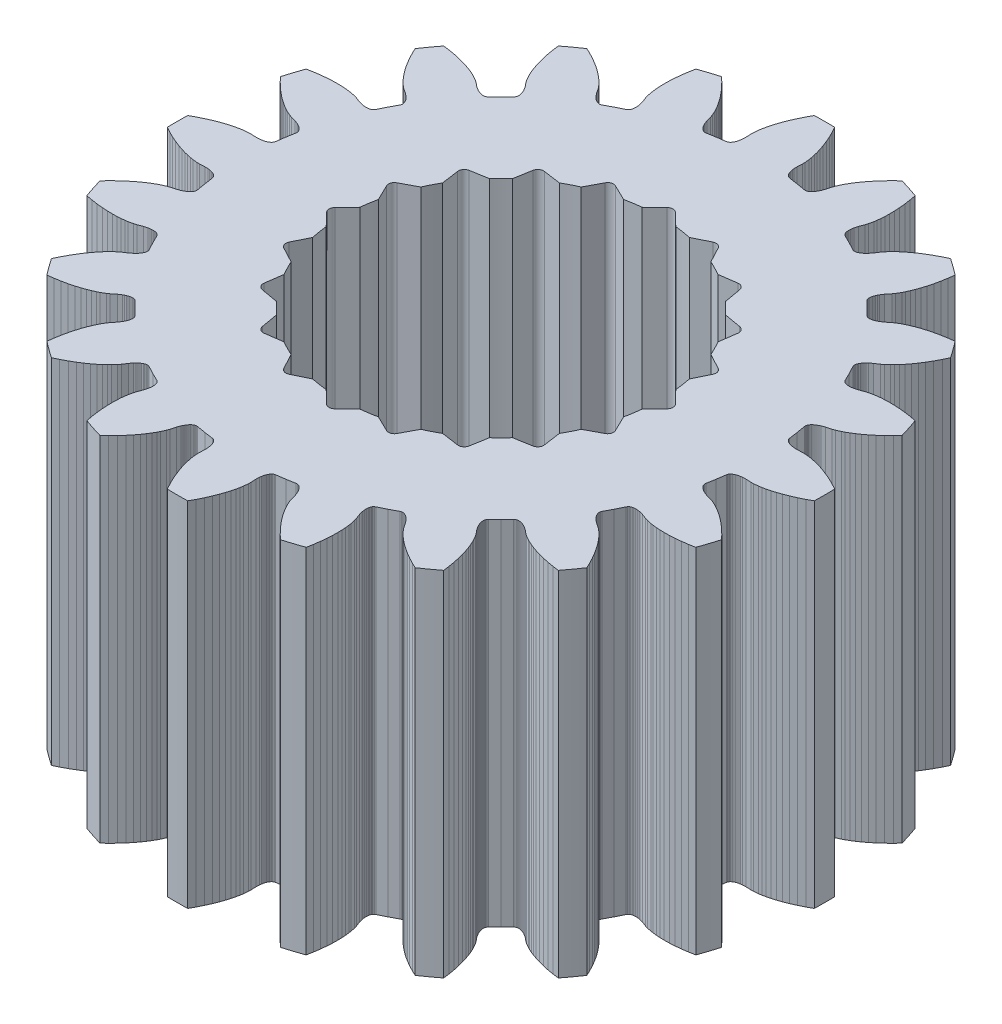
SolidWorks part; units mm, degrees
ref_plane "Front Plane" through (0, 0, 0) normal (0, 0, 1) x (1, 0, 0)
ref_plane "Top Plane" through (0, 0, 0) normal (0, 1, 0) x (1, 0, 0)
ref_plane "Right Plane" through (0, 0, 0) normal (1, 0, 0) x (0, 0, -1)
sketch "Sketch1" plane through (0, 0, 0) normal (0, 1, 0) x (1, 0, 0)
  line L0 (5.2098, 1.4578) -> (5.1322, 1.3823)
  line L1 (5.1322, 1.3823) -> (5.0569, 1.3152)
  line L2 (5.0569, 1.3152) -> (4.9868, 1.2577)
  line L3 (4.9868, 1.2577) -> (4.9194, 1.207)
  line L4 (4.9194, 1.207) -> (4.8581, 1.1647)
  line L5 (4.8581, 1.1647) -> (4.8009, 1.1288)
  line L6 (4.8009, 1.1288) -> (4.75, 1.0997)
  line L7 (4.75, 1.0997) -> (4.7061, 1.0769)
  line L8 (4.7061, 1.0769) -> (4.6364, 1.046)
  line L9 (4.6364, 1.046) -> (4.5924, 1.0307)
  line L10 (4.5924, 1.0307) -> (4.5075, 1.0081)
  line L11 (4.5075, 1.0081) -> (4.4514, 0.9867)
  line L12 (4.4514, 0.9867) -> (4.427, 0.9751)
  line L13 (4.427, 0.9751) -> (4.4051, 0.9628)
  line L14 (4.4051, 0.9628) -> (4.3856, 0.9502)
  line L15 (4.3856, 0.9502) -> (4.3686, 0.9372)
  line L16 (4.3686, 0.9372) -> (4.354, 0.9239)
  line L17 (4.354, 0.9239) -> (4.3419, 0.9105)
  line L18 (4.3419, 0.9105) -> (4.3323, 0.897)
  line L19 (4.3323, 0.897) -> (4.3252, 0.8836)
  line L20 (4.3252, 0.8836) -> (4.3205, 0.8703)
  line L21 (4.3205, 0.8703) -> (4.3182, 0.8572)
  line L22 (4.3182, 0.8572) -> (4.3194, 0.8383)
  line L23 (4.3194, 0.8383) -> (4.3458, 0.6883)
  line L24 (4.3458, 0.6883) -> (4.3671, 0.5375)
  line L25 (4.3671, 0.5375) -> (4.3718, 0.5191)
  line L26 (4.3718, 0.5191) -> (4.378, 0.5074)
  line L27 (4.378, 0.5074) -> (4.3865, 0.4962)
  line L28 (4.3865, 0.4962) -> (4.3975, 0.4856)
  line L29 (4.3975, 0.4856) -> (4.4108, 0.4758)
  line L30 (4.4108, 0.4758) -> (4.4264, 0.4668)
  line L31 (4.4264, 0.4668) -> (4.4444, 0.4587)
  line L32 (4.4444, 0.4587) -> (4.4646, 0.4516)
  line L33 (4.4646, 0.4516) -> (4.487, 0.4455)
  line L34 (4.487, 0.4455) -> (4.5117, 0.4407)
  line L35 (4.5117, 0.4407) -> (4.5385, 0.4371)
  line L36 (4.5385, 0.4371) -> (4.5984, 0.4341)
  line L37 (4.5984, 0.4341) -> (4.6862, 0.4388)
  line L38 (4.6862, 0.4388) -> (4.7327, 0.438)
  line L39 (4.7327, 0.438) -> (4.8085, 0.43)
  line L40 (4.8085, 0.43) -> (4.8574, 0.422)
  line L41 (4.8574, 0.422) -> (4.9147, 0.41)
  line L42 (4.9147, 0.41) -> (4.9802, 0.3935)
  line L43 (4.9802, 0.3935) -> (5.0516, 0.3723)
  line L44 (5.0516, 0.3723) -> (5.1313, 0.3449)
  line L45 (5.1313, 0.3449) -> (5.2159, 0.3118)
  line L46 (5.2159, 0.3118) -> (5.3081, 0.2712)
  line L47 (5.3081, 0.2712) -> (5.4053, 0.2235)
  line L48 (5.4053, 0.2235) -> (5.4973, 0.1736)
  line L49 (5.4973, -0.1736) -> (5.4053, -0.2235)
  line L50 (5.4053, -0.2235) -> (5.3081, -0.2712)
  line L51 (5.3081, -0.2712) -> (5.2159, -0.3118)
  line L52 (5.2159, -0.3118) -> (5.1313, -0.3449)
  line L53 (5.1313, -0.3449) -> (5.0516, -0.3723)
  line L54 (5.0516, -0.3723) -> (4.9802, -0.3935)
  line L55 (4.9802, -0.3935) -> (4.9147, -0.41)
  line L56 (4.9147, -0.41) -> (4.8574, -0.422)
  line L57 (4.8574, -0.422) -> (4.8085, -0.43)
  line L58 (4.8085, -0.43) -> (4.7327, -0.438)
  line L59 (4.7327, -0.438) -> (4.6862, -0.4388)
  line L60 (4.6862, -0.4388) -> (4.5984, -0.4341)
  line L61 (4.5984, -0.4341) -> (4.5385, -0.4371)
  line L62 (4.5385, -0.4371) -> (4.5117, -0.4407)
  line L63 (4.5117, -0.4407) -> (4.487, -0.4455)
  line L64 (4.487, -0.4455) -> (4.4646, -0.4516)
  line L65 (4.4646, -0.4516) -> (4.4444, -0.4587)
  line L66 (4.4444, -0.4587) -> (4.4264, -0.4668)
  line L67 (4.4264, -0.4668) -> (4.4108, -0.4758)
  line L68 (4.4108, -0.4758) -> (4.3975, -0.4856)
  line L69 (4.3975, -0.4856) -> (4.3865, -0.4962)
  line L70 (4.3865, -0.4962) -> (4.378, -0.5074)
  line L71 (4.378, -0.5074) -> (4.3718, -0.5191)
  line L72 (4.3718, -0.5191) -> (4.3671, -0.5375)
  line L73 (4.3671, -0.5375) -> (4.3458, -0.6883)
  line L74 (4.3458, -0.6883) -> (4.3194, -0.8383)
  line L75 (4.3194, -0.8383) -> (4.3182, -0.8572)
  line L76 (4.3182, -0.8572) -> (4.3205, -0.8703)
  line L77 (4.3205, -0.8703) -> (4.3252, -0.8836)
  line L78 (4.3252, -0.8836) -> (4.3323, -0.897)
  line L79 (4.3323, -0.897) -> (4.3419, -0.9105)
  line L80 (4.3419, -0.9105) -> (4.354, -0.9239)
  line L81 (4.354, -0.9239) -> (4.3686, -0.9372)
  line L82 (4.3686, -0.9372) -> (4.3856, -0.9502)
  line L83 (4.3856, -0.9502) -> (4.4051, -0.9628)
  line L84 (4.4051, -0.9628) -> (4.427, -0.9751)
  line L85 (4.427, -0.9751) -> (4.4514, -0.9867)
  line L86 (4.4514, -0.9867) -> (4.5075, -1.0081)
  line L87 (4.5075, -1.0081) -> (4.5924, -1.0307)
  line L88 (4.5924, -1.0307) -> (4.6364, -1.046)
  line L89 (4.6364, -1.046) -> (4.7061, -1.0769)
  line L90 (4.7061, -1.0769) -> (4.75, -1.0997)
  line L91 (4.75, -1.0997) -> (4.8009, -1.1288)
  line L92 (4.8009, -1.1288) -> (4.8581, -1.1647)
  line L93 (4.8581, -1.1647) -> (4.9194, -1.207)
  line L94 (4.9194, -1.207) -> (4.9868, -1.2577)
  line L95 (4.9868, -1.2577) -> (5.0569, -1.3152)
  line L96 (5.0569, -1.3152) -> (5.1322, -1.3823)
  line L97 (5.1322, -1.3823) -> (5.2098, -1.4578)
  line L98 (5.2098, -1.4578) -> (5.2818, -1.5336)
  line L99 (5.1745, -1.8639) -> (5.0717, -1.8829)
  line L100 (5.0717, -1.8829) -> (4.9645, -1.8983)
  line L101 (4.9645, -1.8983) -> (4.8642, -1.9084)
  line L102 (4.8642, -1.9084) -> (4.7736, -1.9137)
  line L103 (4.7736, -1.9137) -> (4.6893, -1.9151)
  line L104 (4.6893, -1.9151) -> (4.6149, -1.9132)
  line L105 (4.6149, -1.9132) -> (4.5475, -1.9087)
  line L106 (4.5475, -1.9087) -> (4.4892, -1.9023)
  line L107 (4.4892, -1.9023) -> (4.4403, -1.8949)
  line L108 (4.4403, -1.8949) -> (4.3657, -1.879)
  line L109 (4.3657, -1.879) -> (4.3212, -1.8655)
  line L110 (4.3212, -1.8655) -> (4.2391, -1.8339)
  line L111 (4.2391, -1.8339) -> (4.1813, -1.8182)
  line L112 (4.1813, -1.8182) -> (4.1547, -1.8133)
  line L113 (4.1547, -1.8133) -> (4.1297, -1.8103)
  line L114 (4.1297, -1.8103) -> (4.1065, -1.8091)
  line L115 (4.1065, -1.8091) -> (4.0851, -1.8096)
  line L116 (4.0851, -1.8096) -> (4.0655, -1.8118)
  line L117 (4.0655, -1.8118) -> (4.0479, -1.8155)
  line L118 (4.0479, -1.8155) -> (4.0322, -1.8208)
  line L119 (4.0322, -1.8208) -> (4.0185, -1.8274)
  line L120 (4.0185, -1.8274) -> (4.0069, -1.8354)
  line L121 (4.0069, -1.8354) -> (3.9974, -1.8447)
  line L122 (3.9974, -1.8447) -> (3.9872, -1.8607)
  line L123 (3.9872, -1.8607) -> (3.9204, -1.9976)
  line L124 (3.9204, -1.9976) -> (3.8489, -2.1321)
  line L125 (3.8489, -2.1321) -> (3.842, -2.1497)
  line L126 (3.842, -2.1497) -> (3.8401, -2.1628)
  line L127 (3.8401, -2.1628) -> (3.8404, -2.1769)
  line L128 (3.8404, -2.1769) -> (3.8431, -2.1919)
  line L129 (3.8431, -2.1919) -> (3.8481, -2.2077)
  line L130 (3.8481, -2.2077) -> (3.8554, -2.2242)
  line L131 (3.8554, -2.2242) -> (3.8652, -2.2413)
  line L132 (3.8652, -2.2413) -> (3.8773, -2.2589)
  line L133 (3.8773, -2.2589) -> (3.892, -2.277)
  line L134 (3.892, -2.277) -> (3.9091, -2.2954)
  line L135 (3.9091, -2.2954) -> (3.9286, -2.314)
  line L136 (3.9286, -2.314) -> (3.9753, -2.3516)
  line L137 (3.9753, -2.3516) -> (4.0491, -2.3994)
  line L138 (4.0491, -2.3994) -> (4.0862, -2.4275)
  line L139 (4.0862, -2.4275) -> (4.1429, -2.4785)
  line L140 (4.1429, -2.4785) -> (4.1777, -2.5137)
  line L141 (4.1777, -2.5137) -> (4.2171, -2.5571)
  line L142 (4.2171, -2.5571) -> (4.2604, -2.609)
  line L143 (4.2604, -2.609) -> (4.3057, -2.6681)
  line L144 (4.3057, -2.6681) -> (4.3541, -2.7371)
  line L145 (4.3541, -2.7371) -> (4.403, -2.8135)
  line L146 (4.403, -2.8135) -> (4.4538, -2.9006)
  line L147 (4.4538, -2.9006) -> (4.5044, -2.9964)
  line L148 (4.5044, -2.9964) -> (4.5494, -3.0907)
  line L149 (4.3453, -3.3717) -> (4.2416, -3.358)
  line L150 (4.2416, -3.358) -> (4.1349, -3.3395)
  line L151 (4.1349, -3.3395) -> (4.0364, -3.3181)
  line L152 (4.0364, -3.3181) -> (3.9486, -3.2952)
  line L153 (3.9486, -3.2952) -> (3.868, -3.2704)
  line L154 (3.868, -3.2704) -> (3.7978, -3.2457)
  line L155 (3.7978, -3.2457) -> (3.7351, -3.2205)
  line L156 (3.7351, -3.2205) -> (3.6817, -3.1965)
  line L157 (3.6817, -3.1965) -> (3.6374, -3.1743)
  line L158 (3.6374, -3.1743) -> (3.5714, -3.1361)
  line L159 (3.5714, -3.1361) -> (3.5332, -3.1095)
  line L160 (3.5332, -3.1095) -> (3.465, -3.0541)
  line L161 (3.465, -3.0541) -> (3.4148, -3.0213)
  line L162 (3.4148, -3.0213) -> (3.391, -3.0084)
  line L163 (3.391, -3.0084) -> (3.3682, -2.9979)
  line L164 (3.3682, -2.9979) -> (3.3465, -2.9895)
  line L165 (3.3465, -2.9895) -> (3.326, -2.9834)
  line L166 (3.326, -2.9834) -> (3.3067, -2.9794)
  line L167 (3.3067, -2.9794) -> (3.2887, -2.9775)
  line L168 (3.2887, -2.9775) -> (3.2722, -2.9777)
  line L169 (3.2722, -2.9777) -> (3.2571, -2.9798)
  line L170 (3.2571, -2.9798) -> (3.2436, -2.9838)
  line L171 (3.2436, -2.9838) -> (3.2317, -2.9896)
  line L172 (3.2317, -2.9896) -> (3.2171, -3.0017)
  line L173 (3.2171, -3.0017) -> (3.1113, -3.1113)
  line L174 (3.1113, -3.1113) -> (3.0017, -3.2171)
  line L175 (3.0017, -3.2171) -> (2.9896, -3.2317)
  line L176 (2.9896, -3.2317) -> (2.9838, -3.2436)
  line L177 (2.9838, -3.2436) -> (2.9798, -3.2571)
  line L178 (2.9798, -3.2571) -> (2.9777, -3.2722)
  line L179 (2.9777, -3.2722) -> (2.9775, -3.2887)
  line L180 (2.9775, -3.2887) -> (2.9794, -3.3067)
  line L181 (2.9794, -3.3067) -> (2.9834, -3.326)
  line L182 (2.9834, -3.326) -> (2.9895, -3.3465)
  line L183 (2.9895, -3.3465) -> (2.9979, -3.3682)
  line L184 (2.9979, -3.3682) -> (3.0084, -3.391)
  line L185 (3.0084, -3.391) -> (3.0213, -3.4148)
  line L186 (3.0213, -3.4148) -> (3.0541, -3.465)
  line L187 (3.0541, -3.465) -> (3.1095, -3.5332)
  line L188 (3.1095, -3.5332) -> (3.1361, -3.5714)
  line L189 (3.1361, -3.5714) -> (3.1743, -3.6374)
  line L190 (3.1743, -3.6374) -> (3.1965, -3.6817)
  line L191 (3.1965, -3.6817) -> (3.2205, -3.7351)
  line L192 (3.2205, -3.7351) -> (3.2457, -3.7978)
  line L193 (3.2457, -3.7978) -> (3.2704, -3.868)
  line L194 (3.2704, -3.868) -> (3.2952, -3.9486)
  line L195 (3.2952, -3.9486) -> (3.3181, -4.0364)
  line L196 (3.3181, -4.0364) -> (3.3395, -4.1349)
  line L197 (3.3395, -4.1349) -> (3.358, -4.2416)
  line L198 (3.358, -4.2416) -> (3.3717, -4.3453)
  line L199 (3.0907, -4.5494) -> (2.9964, -4.5044)
  line L200 (2.9964, -4.5044) -> (2.9006, -4.4538)
  line L201 (2.9006, -4.4538) -> (2.8135, -4.403)
  line L202 (2.8135, -4.403) -> (2.7371, -4.3541)
  line L203 (2.7371, -4.3541) -> (2.6681, -4.3057)
  line L204 (2.6681, -4.3057) -> (2.609, -4.2604)
  line L205 (2.609, -4.2604) -> (2.5571, -4.2171)
  line L206 (2.5571, -4.2171) -> (2.5137, -4.1777)
  line L207 (2.5137, -4.1777) -> (2.4785, -4.1429)
  line L208 (2.4785, -4.1429) -> (2.4275, -4.0862)
  line L209 (2.4275, -4.0862) -> (2.3994, -4.0491)
  line L210 (2.3994, -4.0491) -> (2.3516, -3.9753)
  line L211 (2.3516, -3.9753) -> (2.314, -3.9286)
  line L212 (2.314, -3.9286) -> (2.2954, -3.9091)
  line L213 (2.2954, -3.9091) -> (2.277, -3.892)
  line L214 (2.277, -3.892) -> (2.2589, -3.8773)
  line L215 (2.2589, -3.8773) -> (2.2413, -3.8652)
  line L216 (2.2413, -3.8652) -> (2.2242, -3.8554)
  line L217 (2.2242, -3.8554) -> (2.2077, -3.8481)
  line L218 (2.2077, -3.8481) -> (2.1919, -3.8431)
  line L219 (2.1919, -3.8431) -> (2.1769, -3.8404)
  line L220 (2.1769, -3.8404) -> (2.1628, -3.8401)
  line L221 (2.1628, -3.8401) -> (2.1497, -3.842)
  line L222 (2.1497, -3.842) -> (2.1321, -3.8489)
  line L223 (2.1321, -3.8489) -> (1.9976, -3.9204)
  line L224 (1.9976, -3.9204) -> (1.8607, -3.9872)
  line L225 (1.8607, -3.9872) -> (1.8447, -3.9974)
  line L226 (1.8447, -3.9974) -> (1.8354, -4.0069)
  line L227 (1.8354, -4.0069) -> (1.8274, -4.0185)
  line L228 (1.8274, -4.0185) -> (1.8208, -4.0322)
  line L229 (1.8208, -4.0322) -> (1.8155, -4.0479)
  line L230 (1.8155, -4.0479) -> (1.8118, -4.0655)
  line L231 (1.8118, -4.0655) -> (1.8096, -4.0851)
  line L232 (1.8096, -4.0851) -> (1.8091, -4.1065)
  line L233 (1.8091, -4.1065) -> (1.8103, -4.1297)
  line L234 (1.8103, -4.1297) -> (1.8133, -4.1547)
  line L235 (1.8133, -4.1547) -> (1.8182, -4.1813)
  line L236 (1.8182, -4.1813) -> (1.8339, -4.2391)
  line L237 (1.8339, -4.2391) -> (1.8655, -4.3212)
  line L238 (1.8655, -4.3212) -> (1.879, -4.3657)
  line L239 (1.879, -4.3657) -> (1.8949, -4.4403)
  line L240 (1.8949, -4.4403) -> (1.9023, -4.4892)
  line L241 (1.9023, -4.4892) -> (1.9087, -4.5475)
  line L242 (1.9087, -4.5475) -> (1.9132, -4.6149)
  line L243 (1.9132, -4.6149) -> (1.9151, -4.6893)
  line L244 (1.9151, -4.6893) -> (1.9137, -4.7736)
  line L245 (1.9137, -4.7736) -> (1.9084, -4.8642)
  line L246 (1.9084, -4.8642) -> (1.8983, -4.9645)
  line L247 (1.8983, -4.9645) -> (1.8829, -5.0717)
  line L248 (1.8829, -5.0717) -> (1.8639, -5.1745)
  line L249 (1.5336, -5.2818) -> (1.4578, -5.2098)
  line L250 (1.4578, -5.2098) -> (1.3823, -5.1322)
  line L251 (1.3823, -5.1322) -> (1.3152, -5.0569)
  line L252 (1.3152, -5.0569) -> (1.2577, -4.9868)
  line L253 (1.2577, -4.9868) -> (1.207, -4.9194)
  line L254 (1.207, -4.9194) -> (1.1647, -4.8581)
  line L255 (1.1647, -4.8581) -> (1.1288, -4.8009)
  line L256 (1.1288, -4.8009) -> (1.0997, -4.75)
  line L257 (1.0997, -4.75) -> (1.0769, -4.7061)
  line L258 (1.0769, -4.7061) -> (1.046, -4.6364)
  line L259 (1.046, -4.6364) -> (1.0307, -4.5924)
  line L260 (1.0307, -4.5924) -> (1.0081, -4.5075)
  line L261 (1.0081, -4.5075) -> (0.9867, -4.4514)
  line L262 (0.9867, -4.4514) -> (0.9751, -4.427)
  line L263 (0.9751, -4.427) -> (0.9628, -4.4051)
  line L264 (0.9628, -4.4051) -> (0.9502, -4.3856)
  line L265 (0.9502, -4.3856) -> (0.9372, -4.3686)
  line L266 (0.9372, -4.3686) -> (0.9239, -4.354)
  line L267 (0.9239, -4.354) -> (0.9105, -4.3419)
  line L268 (0.9105, -4.3419) -> (0.897, -4.3323)
  line L269 (0.897, -4.3323) -> (0.8836, -4.3252)
  line L270 (0.8836, -4.3252) -> (0.8703, -4.3205)
  line L271 (0.8703, -4.3205) -> (0.8572, -4.3182)
  line L272 (0.8572, -4.3182) -> (0.8383, -4.3194)
  line L273 (0.8383, -4.3194) -> (0.6883, -4.3458)
  line L274 (0.6883, -4.3458) -> (0.5375, -4.3671)
  line L275 (0.5375, -4.3671) -> (0.5191, -4.3718)
  line L276 (0.5191, -4.3718) -> (0.5074, -4.378)
  line L277 (0.5074, -4.378) -> (0.4962, -4.3865)
  line L278 (0.4962, -4.3865) -> (0.4856, -4.3975)
  line L279 (0.4856, -4.3975) -> (0.4758, -4.4108)
  line L280 (0.4758, -4.4108) -> (0.4668, -4.4264)
  line L281 (0.4668, -4.4264) -> (0.4587, -4.4444)
  line L282 (0.4587, -4.4444) -> (0.4516, -4.4646)
  line L283 (0.4516, -4.4646) -> (0.4455, -4.487)
  line L284 (0.4455, -4.487) -> (0.4407, -4.5117)
  line L285 (0.4407, -4.5117) -> (0.4371, -4.5385)
  line L286 (0.4371, -4.5385) -> (0.4341, -4.5984)
  line L287 (0.4341, -4.5984) -> (0.4388, -4.6862)
  line L288 (0.4388, -4.6862) -> (0.438, -4.7327)
  line L289 (0.438, -4.7327) -> (0.43, -4.8085)
  line L290 (0.43, -4.8085) -> (0.422, -4.8574)
  line L291 (0.422, -4.8574) -> (0.41, -4.9147)
  line L292 (0.41, -4.9147) -> (0.3935, -4.9802)
  line L293 (0.3935, -4.9802) -> (0.3723, -5.0516)
  line L294 (0.3723, -5.0516) -> (0.3449, -5.1313)
  line L295 (0.3449, -5.1313) -> (0.3118, -5.2159)
  line L296 (0.3118, -5.2159) -> (0.2712, -5.3081)
  line L297 (0.2712, -5.3081) -> (0.2235, -5.4053)
  line L298 (0.2235, -5.4053) -> (0.1736, -5.4973)
  line L299 (-0.1736, -5.4973) -> (-0.2235, -5.4053)
  line L300 (-0.2235, -5.4053) -> (-0.2712, -5.3081)
  line L301 (-0.2712, -5.3081) -> (-0.3118, -5.2159)
  line L302 (-0.3118, -5.2159) -> (-0.3449, -5.1313)
  line L303 (-0.3449, -5.1313) -> (-0.3723, -5.0516)
  line L304 (-0.3723, -5.0516) -> (-0.3935, -4.9802)
  line L305 (-0.3935, -4.9802) -> (-0.41, -4.9147)
  line L306 (-0.41, -4.9147) -> (-0.422, -4.8574)
  line L307 (-0.422, -4.8574) -> (-0.43, -4.8085)
  line L308 (-0.43, -4.8085) -> (-0.438, -4.7327)
  line L309 (-0.438, -4.7327) -> (-0.4388, -4.6862)
  line L310 (-0.4388, -4.6862) -> (-0.4341, -4.5984)
  line L311 (-0.4341, -4.5984) -> (-0.4371, -4.5385)
  line L312 (-0.4371, -4.5385) -> (-0.4407, -4.5117)
  line L313 (-0.4407, -4.5117) -> (-0.4455, -4.487)
  line L314 (-0.4455, -4.487) -> (-0.4516, -4.4646)
  line L315 (-0.4516, -4.4646) -> (-0.4587, -4.4444)
  line L316 (-0.4587, -4.4444) -> (-0.4668, -4.4264)
  line L317 (-0.4668, -4.4264) -> (-0.4758, -4.4108)
  line L318 (-0.4758, -4.4108) -> (-0.4856, -4.3975)
  line L319 (-0.4856, -4.3975) -> (-0.4962, -4.3865)
  line L320 (-0.4962, -4.3865) -> (-0.5074, -4.378)
  line L321 (-0.5074, -4.378) -> (-0.5191, -4.3718)
  line L322 (-0.5191, -4.3718) -> (-0.5375, -4.3671)
  line L323 (-0.5375, -4.3671) -> (-0.6883, -4.3458)
  line L324 (-0.6883, -4.3458) -> (-0.8383, -4.3194)
  line L325 (-0.8383, -4.3194) -> (-0.8572, -4.3182)
  line L326 (-0.8572, -4.3182) -> (-0.8703, -4.3205)
  line L327 (-0.8703, -4.3205) -> (-0.8836, -4.3252)
  line L328 (-0.8836, -4.3252) -> (-0.897, -4.3323)
  line L329 (-0.897, -4.3323) -> (-0.9105, -4.3419)
  line L330 (-0.9105, -4.3419) -> (-0.9239, -4.354)
  line L331 (-0.9239, -4.354) -> (-0.9372, -4.3686)
  line L332 (-0.9372, -4.3686) -> (-0.9502, -4.3856)
  line L333 (-0.9502, -4.3856) -> (-0.9628, -4.4051)
  line L334 (-0.9628, -4.4051) -> (-0.9751, -4.427)
  line L335 (-0.9751, -4.427) -> (-0.9867, -4.4514)
  line L336 (-0.9867, -4.4514) -> (-1.0081, -4.5075)
  line L337 (-1.0081, -4.5075) -> (-1.0307, -4.5924)
  line L338 (-1.0307, -4.5924) -> (-1.046, -4.6364)
  line L339 (-1.046, -4.6364) -> (-1.0769, -4.7061)
  line L340 (-1.0769, -4.7061) -> (-1.0997, -4.75)
  line L341 (-1.0997, -4.75) -> (-1.1288, -4.8009)
  line L342 (-1.1288, -4.8009) -> (-1.1647, -4.8581)
  line L343 (-1.1647, -4.8581) -> (-1.207, -4.9194)
  line L344 (-1.207, -4.9194) -> (-1.2577, -4.9868)
  line L345 (-1.2577, -4.9868) -> (-1.3152, -5.0569)
  line L346 (-1.3152, -5.0569) -> (-1.3823, -5.1322)
  line L347 (-1.3823, -5.1322) -> (-1.4578, -5.2098)
  line L348 (-1.4578, -5.2098) -> (-1.5336, -5.2818)
  line L349 (-1.8639, -5.1745) -> (-1.8829, -5.0717)
  line L350 (-1.8829, -5.0717) -> (-1.8983, -4.9645)
  line L351 (-1.8983, -4.9645) -> (-1.9084, -4.8642)
  line L352 (-1.9084, -4.8642) -> (-1.9137, -4.7736)
  line L353 (-1.9137, -4.7736) -> (-1.9151, -4.6893)
  line L354 (-1.9151, -4.6893) -> (-1.9132, -4.6149)
  line L355 (-1.9132, -4.6149) -> (-1.9087, -4.5475)
  line L356 (-1.9087, -4.5475) -> (-1.9023, -4.4892)
  line L357 (-1.9023, -4.4892) -> (-1.8949, -4.4403)
  line L358 (-1.8949, -4.4403) -> (-1.879, -4.3657)
  line L359 (-1.879, -4.3657) -> (-1.8655, -4.3212)
  line L360 (-1.8655, -4.3212) -> (-1.8339, -4.2391)
  line L361 (-1.8339, -4.2391) -> (-1.8182, -4.1813)
  line L362 (-1.8182, -4.1813) -> (-1.8133, -4.1547)
  line L363 (-1.8133, -4.1547) -> (-1.8103, -4.1297)
  line L364 (-1.8103, -4.1297) -> (-1.8091, -4.1065)
  line L365 (-1.8091, -4.1065) -> (-1.8096, -4.0851)
  line L366 (-1.8096, -4.0851) -> (-1.8118, -4.0655)
  line L367 (-1.8118, -4.0655) -> (-1.8155, -4.0479)
  line L368 (-1.8155, -4.0479) -> (-1.8208, -4.0322)
  line L369 (-1.8208, -4.0322) -> (-1.8274, -4.0185)
  line L370 (-1.8274, -4.0185) -> (-1.8354, -4.0069)
  line L371 (-1.8354, -4.0069) -> (-1.8447, -3.9974)
  line L372 (-1.8447, -3.9974) -> (-1.8607, -3.9872)
  line L373 (-1.8607, -3.9872) -> (-1.9976, -3.9204)
  line L374 (-1.9976, -3.9204) -> (-2.1321, -3.8489)
  line L375 (-2.1321, -3.8489) -> (-2.1497, -3.842)
  line L376 (-2.1497, -3.842) -> (-2.1628, -3.8401)
  line L377 (-2.1628, -3.8401) -> (-2.1769, -3.8404)
  line L378 (-2.1769, -3.8404) -> (-2.1919, -3.8431)
  line L379 (-2.1919, -3.8431) -> (-2.2077, -3.8481)
  line L380 (-2.2077, -3.8481) -> (-2.2242, -3.8554)
  line L381 (-2.2242, -3.8554) -> (-2.2413, -3.8652)
  line L382 (-2.2413, -3.8652) -> (-2.2589, -3.8773)
  line L383 (-2.2589, -3.8773) -> (-2.277, -3.892)
  line L384 (-2.277, -3.892) -> (-2.2954, -3.9091)
  line L385 (-2.2954, -3.9091) -> (-2.314, -3.9286)
  line L386 (-2.314, -3.9286) -> (-2.3516, -3.9753)
  line L387 (-2.3516, -3.9753) -> (-2.3994, -4.0491)
  line L388 (-2.3994, -4.0491) -> (-2.4275, -4.0862)
  line L389 (-2.4275, -4.0862) -> (-2.4785, -4.1429)
  line L390 (-2.4785, -4.1429) -> (-2.5137, -4.1777)
  line L391 (-2.5137, -4.1777) -> (-2.5571, -4.2171)
  line L392 (-2.5571, -4.2171) -> (-2.609, -4.2604)
  line L393 (-2.609, -4.2604) -> (-2.6681, -4.3057)
  line L394 (-2.6681, -4.3057) -> (-2.7371, -4.3541)
  line L395 (-2.7371, -4.3541) -> (-2.8135, -4.403)
  line L396 (-2.8135, -4.403) -> (-2.9006, -4.4538)
  line L397 (-2.9006, -4.4538) -> (-2.9964, -4.5044)
  line L398 (-2.9964, -4.5044) -> (-3.0907, -4.5494)
  line L399 (-3.3717, -4.3453) -> (-3.358, -4.2416)
  line L400 (-3.358, -4.2416) -> (-3.3395, -4.1349)
  line L401 (-3.3395, -4.1349) -> (-3.3181, -4.0364)
  line L402 (-3.3181, -4.0364) -> (-3.2952, -3.9486)
  line L403 (-3.2952, -3.9486) -> (-3.2704, -3.868)
  line L404 (-3.2704, -3.868) -> (-3.2457, -3.7978)
  line L405 (-3.2457, -3.7978) -> (-3.2205, -3.7351)
  line L406 (-3.2205, -3.7351) -> (-3.1965, -3.6817)
  line L407 (-3.1965, -3.6817) -> (-3.1743, -3.6374)
  line L408 (-3.1743, -3.6374) -> (-3.1361, -3.5714)
  line L409 (-3.1361, -3.5714) -> (-3.1095, -3.5332)
  line L410 (-3.1095, -3.5332) -> (-3.0541, -3.465)
  line L411 (-3.0541, -3.465) -> (-3.0213, -3.4148)
  line L412 (-3.0213, -3.4148) -> (-3.0084, -3.391)
  line L413 (-3.0084, -3.391) -> (-2.9979, -3.3682)
  line L414 (-2.9979, -3.3682) -> (-2.9895, -3.3465)
  line L415 (-2.9895, -3.3465) -> (-2.9834, -3.326)
  line L416 (-2.9834, -3.326) -> (-2.9794, -3.3067)
  line L417 (-2.9794, -3.3067) -> (-2.9775, -3.2887)
  line L418 (-2.9775, -3.2887) -> (-2.9777, -3.2722)
  line L419 (-2.9777, -3.2722) -> (-2.9798, -3.2571)
  line L420 (-2.9798, -3.2571) -> (-2.9838, -3.2436)
  line L421 (-2.9838, -3.2436) -> (-2.9896, -3.2317)
  line L422 (-2.9896, -3.2317) -> (-3.0017, -3.2171)
  line L423 (-3.0017, -3.2171) -> (-3.1113, -3.1113)
  line L424 (-3.1113, -3.1113) -> (-3.2171, -3.0017)
  line L425 (-3.2171, -3.0017) -> (-3.2317, -2.9896)
  line L426 (-3.2317, -2.9896) -> (-3.2436, -2.9838)
  line L427 (-3.2436, -2.9838) -> (-3.2571, -2.9798)
  line L428 (-3.2571, -2.9798) -> (-3.2722, -2.9777)
  line L429 (-3.2722, -2.9777) -> (-3.2887, -2.9775)
  line L430 (-3.2887, -2.9775) -> (-3.3067, -2.9794)
  line L431 (-3.3067, -2.9794) -> (-3.326, -2.9834)
  line L432 (-3.326, -2.9834) -> (-3.3465, -2.9895)
  line L433 (-3.3465, -2.9895) -> (-3.3682, -2.9979)
  line L434 (-3.3682, -2.9979) -> (-3.391, -3.0084)
  line L435 (-3.391, -3.0084) -> (-3.4148, -3.0213)
  line L436 (-3.4148, -3.0213) -> (-3.465, -3.0541)
  line L437 (-3.465, -3.0541) -> (-3.5332, -3.1095)
  line L438 (-3.5332, -3.1095) -> (-3.5714, -3.1361)
  line L439 (-3.5714, -3.1361) -> (-3.6374, -3.1743)
  line L440 (-3.6374, -3.1743) -> (-3.6817, -3.1965)
  line L441 (-3.6817, -3.1965) -> (-3.7351, -3.2205)
  line L442 (-3.7351, -3.2205) -> (-3.7978, -3.2457)
  line L443 (-3.7978, -3.2457) -> (-3.868, -3.2704)
  line L444 (-3.868, -3.2704) -> (-3.9486, -3.2952)
  line L445 (-3.9486, -3.2952) -> (-4.0364, -3.3181)
  line L446 (-4.0364, -3.3181) -> (-4.1349, -3.3395)
  line L447 (-4.1349, -3.3395) -> (-4.2416, -3.358)
  line L448 (-4.2416, -3.358) -> (-4.3453, -3.3717)
  line L449 (-4.5494, -3.0907) -> (-4.5044, -2.9964)
  line L450 (-4.5044, -2.9964) -> (-4.4538, -2.9006)
  line L451 (-4.4538, -2.9006) -> (-4.403, -2.8135)
  line L452 (-4.403, -2.8135) -> (-4.3541, -2.7371)
  line L453 (-4.3541, -2.7371) -> (-4.3057, -2.6681)
  line L454 (-4.3057, -2.6681) -> (-4.2604, -2.609)
  line L455 (-4.2604, -2.609) -> (-4.2171, -2.5571)
  line L456 (-4.2171, -2.5571) -> (-4.1777, -2.5137)
  line L457 (-4.1777, -2.5137) -> (-4.1429, -2.4785)
  line L458 (-4.1429, -2.4785) -> (-4.0862, -2.4275)
  line L459 (-4.0862, -2.4275) -> (-4.0491, -2.3994)
  line L460 (-4.0491, -2.3994) -> (-3.9753, -2.3516)
  line L461 (-3.9753, -2.3516) -> (-3.9286, -2.314)
  line L462 (-3.9286, -2.314) -> (-3.9091, -2.2954)
  line L463 (-3.9091, -2.2954) -> (-3.892, -2.277)
  line L464 (-3.892, -2.277) -> (-3.8773, -2.2589)
  line L465 (-3.8773, -2.2589) -> (-3.8652, -2.2413)
  line L466 (-3.8652, -2.2413) -> (-3.8554, -2.2242)
  line L467 (-3.8554, -2.2242) -> (-3.8481, -2.2077)
  line L468 (-3.8481, -2.2077) -> (-3.8431, -2.1919)
  line L469 (-3.8431, -2.1919) -> (-3.8404, -2.1769)
  line L470 (-3.8404, -2.1769) -> (-3.8401, -2.1628)
  line L471 (-3.8401, -2.1628) -> (-3.842, -2.1497)
  line L472 (-3.842, -2.1497) -> (-3.8489, -2.1321)
  line L473 (-3.8489, -2.1321) -> (-3.9204, -1.9976)
  line L474 (-3.9204, -1.9976) -> (-3.9872, -1.8607)
  line L475 (-3.9872, -1.8607) -> (-3.9974, -1.8447)
  line L476 (-3.9974, -1.8447) -> (-4.0069, -1.8354)
  line L477 (-4.0069, -1.8354) -> (-4.0185, -1.8274)
  line L478 (-4.0185, -1.8274) -> (-4.0322, -1.8208)
  line L479 (-4.0322, -1.8208) -> (-4.0479, -1.8155)
  line L480 (-4.0479, -1.8155) -> (-4.0655, -1.8118)
  line L481 (-4.0655, -1.8118) -> (-4.0851, -1.8096)
  line L482 (-4.0851, -1.8096) -> (-4.1065, -1.8091)
  line L483 (-4.1065, -1.8091) -> (-4.1297, -1.8103)
  line L484 (-4.1297, -1.8103) -> (-4.1547, -1.8133)
  line L485 (-4.1547, -1.8133) -> (-4.1813, -1.8182)
  line L486 (-4.1813, -1.8182) -> (-4.2391, -1.8339)
  line L487 (-4.2391, -1.8339) -> (-4.3212, -1.8655)
  line L488 (-4.3212, -1.8655) -> (-4.3657, -1.879)
  line L489 (-4.3657, -1.879) -> (-4.4403, -1.8949)
  line L490 (-4.4403, -1.8949) -> (-4.4892, -1.9023)
  line L491 (-4.4892, -1.9023) -> (-4.5475, -1.9087)
  line L492 (-4.5475, -1.9087) -> (-4.6149, -1.9132)
  line L493 (-4.6149, -1.9132) -> (-4.6893, -1.9151)
  line L494 (-4.6893, -1.9151) -> (-4.7736, -1.9137)
  line L495 (-4.7736, -1.9137) -> (-4.8642, -1.9084)
  line L496 (-4.8642, -1.9084) -> (-4.9645, -1.8983)
  line L497 (-4.9645, -1.8983) -> (-5.0717, -1.8829)
  line L498 (-5.0717, -1.8829) -> (-5.1745, -1.8639)
  line L499 (-5.2818, -1.5336) -> (-5.2098, -1.4578)
  line L500 (-5.2098, -1.4578) -> (-5.1322, -1.3823)
  line L501 (-5.1322, -1.3823) -> (-5.0569, -1.3152)
  line L502 (-5.0569, -1.3152) -> (-4.9868, -1.2577)
  line L503 (-4.9868, -1.2577) -> (-4.9194, -1.207)
  line L504 (-4.9194, -1.207) -> (-4.8581, -1.1647)
  line L505 (-4.8581, -1.1647) -> (-4.8009, -1.1288)
  line L506 (-4.8009, -1.1288) -> (-4.75, -1.0997)
  line L507 (-4.75, -1.0997) -> (-4.7061, -1.0769)
  line L508 (-4.7061, -1.0769) -> (-4.6364, -1.046)
  line L509 (-4.6364, -1.046) -> (-4.5924, -1.0307)
  line L510 (-4.5924, -1.0307) -> (-4.5075, -1.0081)
  line L511 (-4.5075, -1.0081) -> (-4.4514, -0.9867)
  line L512 (-4.4514, -0.9867) -> (-4.427, -0.9751)
  line L513 (-4.427, -0.9751) -> (-4.4051, -0.9628)
  line L514 (-4.4051, -0.9628) -> (-4.3856, -0.9502)
  line L515 (-4.3856, -0.9502) -> (-4.3686, -0.9372)
  line L516 (-4.3686, -0.9372) -> (-4.354, -0.9239)
  line L517 (-4.354, -0.9239) -> (-4.3419, -0.9105)
  line L518 (-4.3419, -0.9105) -> (-4.3323, -0.897)
  line L519 (-4.3323, -0.897) -> (-4.3252, -0.8836)
  line L520 (-4.3252, -0.8836) -> (-4.3205, -0.8703)
  line L521 (-4.3205, -0.8703) -> (-4.3182, -0.8572)
  line L522 (-4.3182, -0.8572) -> (-4.3194, -0.8383)
  line L523 (-4.3194, -0.8383) -> (-4.3458, -0.6883)
  line L524 (-4.3458, -0.6883) -> (-4.3671, -0.5375)
  line L525 (-4.3671, -0.5375) -> (-4.3718, -0.5191)
  line L526 (-4.3718, -0.5191) -> (-4.378, -0.5074)
  line L527 (-4.378, -0.5074) -> (-4.3865, -0.4962)
  line L528 (-4.3865, -0.4962) -> (-4.3975, -0.4856)
  line L529 (-4.3975, -0.4856) -> (-4.4108, -0.4758)
  line L530 (-4.4108, -0.4758) -> (-4.4264, -0.4668)
  line L531 (-4.4264, -0.4668) -> (-4.4444, -0.4587)
  line L532 (-4.4444, -0.4587) -> (-4.4646, -0.4516)
  line L533 (-4.4646, -0.4516) -> (-4.487, -0.4455)
  line L534 (-4.487, -0.4455) -> (-4.5117, -0.4407)
  line L535 (-4.5117, -0.4407) -> (-4.5385, -0.4371)
  line L536 (-4.5385, -0.4371) -> (-4.5984, -0.4341)
  line L537 (-4.5984, -0.4341) -> (-4.6862, -0.4388)
  line L538 (-4.6862, -0.4388) -> (-4.7327, -0.438)
  line L539 (-4.7327, -0.438) -> (-4.8085, -0.43)
  line L540 (-4.8085, -0.43) -> (-4.8574, -0.422)
  line L541 (-4.8574, -0.422) -> (-4.9147, -0.41)
  line L542 (-4.9147, -0.41) -> (-4.9802, -0.3935)
  line L543 (-4.9802, -0.3935) -> (-5.0516, -0.3723)
  line L544 (-5.0516, -0.3723) -> (-5.1313, -0.3449)
  line L545 (-5.1313, -0.3449) -> (-5.2159, -0.3118)
  line L546 (-5.2159, -0.3118) -> (-5.3081, -0.2712)
  line L547 (-5.3081, -0.2712) -> (-5.4053, -0.2235)
  line L548 (-5.4053, -0.2235) -> (-5.4973, -0.1736)
  line L549 (-5.4973, 0.1736) -> (-5.4053, 0.2235)
  line L550 (-5.4053, 0.2235) -> (-5.3081, 0.2712)
  line L551 (-5.3081, 0.2712) -> (-5.2159, 0.3118)
  line L552 (-5.2159, 0.3118) -> (-5.1313, 0.3449)
  line L553 (-5.1313, 0.3449) -> (-5.0516, 0.3723)
  line L554 (-5.0516, 0.3723) -> (-4.9802, 0.3935)
  line L555 (-4.9802, 0.3935) -> (-4.9147, 0.41)
  line L556 (-4.9147, 0.41) -> (-4.8574, 0.422)
  line L557 (-4.8574, 0.422) -> (-4.8085, 0.43)
  line L558 (-4.8085, 0.43) -> (-4.7327, 0.438)
  line L559 (-4.7327, 0.438) -> (-4.6862, 0.4388)
  line L560 (-4.6862, 0.4388) -> (-4.5984, 0.4341)
  line L561 (-4.5984, 0.4341) -> (-4.5385, 0.4371)
  line L562 (-4.5385, 0.4371) -> (-4.5117, 0.4407)
  line L563 (-4.5117, 0.4407) -> (-4.487, 0.4455)
  line L564 (-4.487, 0.4455) -> (-4.4646, 0.4516)
  line L565 (-4.4646, 0.4516) -> (-4.4444, 0.4587)
  line L566 (-4.4444, 0.4587) -> (-4.4264, 0.4668)
  line L567 (-4.4264, 0.4668) -> (-4.4108, 0.4758)
  line L568 (-4.4108, 0.4758) -> (-4.3975, 0.4856)
  line L569 (-4.3975, 0.4856) -> (-4.3865, 0.4962)
  line L570 (-4.3865, 0.4962) -> (-4.378, 0.5074)
  line L571 (-4.378, 0.5074) -> (-4.3718, 0.5191)
  line L572 (-4.3718, 0.5191) -> (-4.3671, 0.5375)
  line L573 (-4.3671, 0.5375) -> (-4.3458, 0.6883)
  line L574 (-4.3458, 0.6883) -> (-4.3194, 0.8383)
  line L575 (-4.3194, 0.8383) -> (-4.3182, 0.8572)
  line L576 (-4.3182, 0.8572) -> (-4.3205, 0.8703)
  line L577 (-4.3205, 0.8703) -> (-4.3252, 0.8836)
  line L578 (-4.3252, 0.8836) -> (-4.3323, 0.897)
  line L579 (-4.3323, 0.897) -> (-4.3419, 0.9105)
  line L580 (-4.3419, 0.9105) -> (-4.354, 0.9239)
  line L581 (-4.354, 0.9239) -> (-4.3686, 0.9372)
  line L582 (-4.3686, 0.9372) -> (-4.3856, 0.9502)
  line L583 (-4.3856, 0.9502) -> (-4.4051, 0.9628)
  line L584 (-4.4051, 0.9628) -> (-4.427, 0.9751)
  line L585 (-4.427, 0.9751) -> (-4.4514, 0.9867)
  line L586 (-4.4514, 0.9867) -> (-4.5075, 1.0081)
  line L587 (-4.5075, 1.0081) -> (-4.5924, 1.0307)
  line L588 (-4.5924, 1.0307) -> (-4.6364, 1.046)
  line L589 (-4.6364, 1.046) -> (-4.7061, 1.0769)
  line L590 (-4.7061, 1.0769) -> (-4.75, 1.0997)
  line L591 (-4.75, 1.0997) -> (-4.8009, 1.1288)
  line L592 (-4.8009, 1.1288) -> (-4.8581, 1.1647)
  line L593 (-4.8581, 1.1647) -> (-4.9194, 1.207)
  line L594 (-4.9194, 1.207) -> (-4.9868, 1.2577)
  line L595 (-4.9868, 1.2577) -> (-5.0569, 1.3152)
  line L596 (-5.0569, 1.3152) -> (-5.1322, 1.3823)
  line L597 (-5.1322, 1.3823) -> (-5.2098, 1.4578)
  line L598 (-5.2098, 1.4578) -> (-5.2818, 1.5336)
  line L599 (-5.1745, 1.8639) -> (-5.0717, 1.8829)
  line L600 (-5.0717, 1.8829) -> (-4.9645, 1.8983)
  line L601 (-4.9645, 1.8983) -> (-4.8642, 1.9084)
  line L602 (-4.8642, 1.9084) -> (-4.7736, 1.9137)
  line L603 (-4.7736, 1.9137) -> (-4.6893, 1.9151)
  line L604 (-4.6893, 1.9151) -> (-4.6149, 1.9132)
  line L605 (-4.6149, 1.9132) -> (-4.5475, 1.9087)
  line L606 (-4.5475, 1.9087) -> (-4.4892, 1.9023)
  line L607 (-4.4892, 1.9023) -> (-4.4403, 1.8949)
  line L608 (-4.4403, 1.8949) -> (-4.3657, 1.879)
  line L609 (-4.3657, 1.879) -> (-4.3212, 1.8655)
  line L610 (-4.3212, 1.8655) -> (-4.2391, 1.8339)
  line L611 (-4.2391, 1.8339) -> (-4.1813, 1.8182)
  line L612 (-4.1813, 1.8182) -> (-4.1547, 1.8133)
  line L613 (-4.1547, 1.8133) -> (-4.1297, 1.8103)
  line L614 (-4.1297, 1.8103) -> (-4.1065, 1.8091)
  line L615 (-4.1065, 1.8091) -> (-4.0851, 1.8096)
  line L616 (-4.0851, 1.8096) -> (-4.0655, 1.8118)
  line L617 (-4.0655, 1.8118) -> (-4.0479, 1.8155)
  line L618 (-4.0479, 1.8155) -> (-4.0322, 1.8208)
  line L619 (-4.0322, 1.8208) -> (-4.0185, 1.8274)
  line L620 (-4.0185, 1.8274) -> (-4.0069, 1.8354)
  line L621 (-4.0069, 1.8354) -> (-3.9974, 1.8447)
  line L622 (-3.9974, 1.8447) -> (-3.9872, 1.8607)
  line L623 (-3.9872, 1.8607) -> (-3.9204, 1.9976)
  line L624 (-3.9204, 1.9976) -> (-3.8489, 2.1321)
  line L625 (-3.8489, 2.1321) -> (-3.842, 2.1497)
  line L626 (-3.842, 2.1497) -> (-3.8401, 2.1628)
  line L627 (-3.8401, 2.1628) -> (-3.8404, 2.1769)
  line L628 (-3.8404, 2.1769) -> (-3.8431, 2.1919)
  line L629 (-3.8431, 2.1919) -> (-3.8481, 2.2077)
  line L630 (-3.8481, 2.2077) -> (-3.8554, 2.2242)
  line L631 (-3.8554, 2.2242) -> (-3.8652, 2.2413)
  line L632 (-3.8652, 2.2413) -> (-3.8773, 2.2589)
  line L633 (-3.8773, 2.2589) -> (-3.892, 2.277)
  line L634 (-3.892, 2.277) -> (-3.9091, 2.2954)
  line L635 (-3.9091, 2.2954) -> (-3.9286, 2.314)
  line L636 (-3.9286, 2.314) -> (-3.9753, 2.3516)
  line L637 (-3.9753, 2.3516) -> (-4.0491, 2.3994)
  line L638 (-4.0491, 2.3994) -> (-4.0862, 2.4275)
  line L639 (-4.0862, 2.4275) -> (-4.1429, 2.4785)
  line L640 (-4.1429, 2.4785) -> (-4.1777, 2.5137)
  line L641 (-4.1777, 2.5137) -> (-4.2171, 2.5571)
  line L642 (-4.2171, 2.5571) -> (-4.2604, 2.609)
  line L643 (-4.2604, 2.609) -> (-4.3057, 2.6681)
  line L644 (-4.3057, 2.6681) -> (-4.3541, 2.7371)
  line L645 (-4.3541, 2.7371) -> (-4.403, 2.8135)
  line L646 (-4.403, 2.8135) -> (-4.4538, 2.9006)
  line L647 (-4.4538, 2.9006) -> (-4.5044, 2.9964)
  line L648 (-4.5044, 2.9964) -> (-4.5494, 3.0907)
  line L649 (-4.3453, 3.3717) -> (-4.2416, 3.358)
  line L650 (-4.2416, 3.358) -> (-4.1349, 3.3395)
  line L651 (-4.1349, 3.3395) -> (-4.0364, 3.3181)
  line L652 (-4.0364, 3.3181) -> (-3.9486, 3.2952)
  line L653 (-3.9486, 3.2952) -> (-3.868, 3.2704)
  line L654 (-3.868, 3.2704) -> (-3.7978, 3.2457)
  line L655 (-3.7978, 3.2457) -> (-3.7351, 3.2205)
  line L656 (-3.7351, 3.2205) -> (-3.6817, 3.1965)
  line L657 (-3.6817, 3.1965) -> (-3.6374, 3.1743)
  line L658 (-3.6374, 3.1743) -> (-3.5714, 3.1361)
  line L659 (-3.5714, 3.1361) -> (-3.5332, 3.1095)
  line L660 (-3.5332, 3.1095) -> (-3.465, 3.0541)
  line L661 (-3.465, 3.0541) -> (-3.4148, 3.0213)
  line L662 (-3.4148, 3.0213) -> (-3.391, 3.0084)
  line L663 (-3.391, 3.0084) -> (-3.3682, 2.9979)
  line L664 (-3.3682, 2.9979) -> (-3.3465, 2.9895)
  line L665 (-3.3465, 2.9895) -> (-3.326, 2.9834)
  line L666 (-3.326, 2.9834) -> (-3.3067, 2.9794)
  line L667 (-3.3067, 2.9794) -> (-3.2887, 2.9775)
  line L668 (-3.2887, 2.9775) -> (-3.2722, 2.9777)
  line L669 (-3.2722, 2.9777) -> (-3.2571, 2.9798)
  line L670 (-3.2571, 2.9798) -> (-3.2436, 2.9838)
  line L671 (-3.2436, 2.9838) -> (-3.2317, 2.9896)
  line L672 (-3.2317, 2.9896) -> (-3.2171, 3.0017)
  line L673 (-3.2171, 3.0017) -> (-3.1113, 3.1113)
  line L674 (-3.1113, 3.1113) -> (-3.0017, 3.2171)
  line L675 (-3.0017, 3.2171) -> (-2.9896, 3.2317)
  line L676 (-2.9896, 3.2317) -> (-2.9838, 3.2436)
  line L677 (-2.9838, 3.2436) -> (-2.9798, 3.2571)
  line L678 (-2.9798, 3.2571) -> (-2.9777, 3.2722)
  line L679 (-2.9777, 3.2722) -> (-2.9775, 3.2887)
  line L680 (-2.9775, 3.2887) -> (-2.9794, 3.3067)
  line L681 (-2.9794, 3.3067) -> (-2.9834, 3.326)
  line L682 (-2.9834, 3.326) -> (-2.9895, 3.3465)
  line L683 (-2.9895, 3.3465) -> (-2.9979, 3.3682)
  line L684 (-2.9979, 3.3682) -> (-3.0084, 3.391)
  line L685 (-3.0084, 3.391) -> (-3.0213, 3.4148)
  line L686 (-3.0213, 3.4148) -> (-3.0541, 3.465)
  line L687 (-3.0541, 3.465) -> (-3.1095, 3.5332)
  line L688 (-3.1095, 3.5332) -> (-3.1361, 3.5714)
  line L689 (-3.1361, 3.5714) -> (-3.1743, 3.6374)
  line L690 (-3.1743, 3.6374) -> (-3.1965, 3.6817)
  line L691 (-3.1965, 3.6817) -> (-3.2205, 3.7351)
  line L692 (-3.2205, 3.7351) -> (-3.2457, 3.7978)
  line L693 (-3.2457, 3.7978) -> (-3.2704, 3.868)
  line L694 (-3.2704, 3.868) -> (-3.2952, 3.9486)
  line L695 (-3.2952, 3.9486) -> (-3.3181, 4.0364)
  line L696 (-3.3181, 4.0364) -> (-3.3395, 4.1349)
  line L697 (-3.3395, 4.1349) -> (-3.358, 4.2416)
  line L698 (-3.358, 4.2416) -> (-3.3717, 4.3453)
  line L699 (-3.0907, 4.5494) -> (-2.9964, 4.5044)
  line L700 (-2.9964, 4.5044) -> (-2.9006, 4.4538)
  line L701 (-2.9006, 4.4538) -> (-2.8135, 4.403)
  line L702 (-2.8135, 4.403) -> (-2.7371, 4.3541)
  line L703 (-2.7371, 4.3541) -> (-2.6681, 4.3057)
  line L704 (-2.6681, 4.3057) -> (-2.609, 4.2604)
  line L705 (-2.609, 4.2604) -> (-2.5571, 4.2171)
  line L706 (-2.5571, 4.2171) -> (-2.5137, 4.1777)
  line L707 (-2.5137, 4.1777) -> (-2.4785, 4.1429)
  line L708 (-2.4785, 4.1429) -> (-2.4275, 4.0862)
  line L709 (-2.4275, 4.0862) -> (-2.3994, 4.0491)
  line L710 (-2.3994, 4.0491) -> (-2.3516, 3.9753)
  line L711 (-2.3516, 3.9753) -> (-2.314, 3.9286)
  line L712 (-2.314, 3.9286) -> (-2.2954, 3.9091)
  line L713 (-2.2954, 3.9091) -> (-2.277, 3.892)
  line L714 (-2.277, 3.892) -> (-2.2589, 3.8773)
  line L715 (-2.2589, 3.8773) -> (-2.2413, 3.8652)
  line L716 (-2.2413, 3.8652) -> (-2.2242, 3.8554)
  line L717 (-2.2242, 3.8554) -> (-2.2077, 3.8481)
  line L718 (-2.2077, 3.8481) -> (-2.1919, 3.8431)
  line L719 (-2.1919, 3.8431) -> (-2.1769, 3.8404)
  line L720 (-2.1769, 3.8404) -> (-2.1628, 3.8401)
  line L721 (-2.1628, 3.8401) -> (-2.1497, 3.842)
  line L722 (-2.1497, 3.842) -> (-2.1321, 3.8489)
  line L723 (-2.1321, 3.8489) -> (-1.9976, 3.9204)
  line L724 (-1.9976, 3.9204) -> (-1.8607, 3.9872)
  line L725 (-1.8607, 3.9872) -> (-1.8447, 3.9974)
  line L726 (-1.8447, 3.9974) -> (-1.8354, 4.0069)
  line L727 (-1.8354, 4.0069) -> (-1.8274, 4.0185)
  line L728 (-1.8274, 4.0185) -> (-1.8208, 4.0322)
  line L729 (-1.8208, 4.0322) -> (-1.8155, 4.0479)
  line L730 (-1.8155, 4.0479) -> (-1.8118, 4.0655)
  line L731 (-1.8118, 4.0655) -> (-1.8096, 4.0851)
  line L732 (-1.8096, 4.0851) -> (-1.8091, 4.1065)
  line L733 (-1.8091, 4.1065) -> (-1.8103, 4.1297)
  line L734 (-1.8103, 4.1297) -> (-1.8133, 4.1547)
  line L735 (-1.8133, 4.1547) -> (-1.8182, 4.1813)
  line L736 (-1.8182, 4.1813) -> (-1.8339, 4.2391)
  line L737 (-1.8339, 4.2391) -> (-1.8655, 4.3212)
  line L738 (-1.8655, 4.3212) -> (-1.879, 4.3657)
  line L739 (-1.879, 4.3657) -> (-1.8949, 4.4403)
  line L740 (-1.8949, 4.4403) -> (-1.9023, 4.4892)
  line L741 (-1.9023, 4.4892) -> (-1.9087, 4.5475)
  line L742 (-1.9087, 4.5475) -> (-1.9132, 4.6149)
  line L743 (-1.9132, 4.6149) -> (-1.9151, 4.6893)
  line L744 (-1.9151, 4.6893) -> (-1.9137, 4.7736)
  line L745 (-1.9137, 4.7736) -> (-1.9084, 4.8642)
  line L746 (-1.9084, 4.8642) -> (-1.8983, 4.9645)
  line L747 (-1.8983, 4.9645) -> (-1.8829, 5.0717)
  line L748 (-1.8829, 5.0717) -> (-1.8639, 5.1745)
  line L749 (-1.5336, 5.2818) -> (-1.4578, 5.2098)
  line L750 (-1.4578, 5.2098) -> (-1.3823, 5.1322)
  line L751 (-1.3823, 5.1322) -> (-1.3152, 5.0569)
  line L752 (-1.3152, 5.0569) -> (-1.2577, 4.9868)
  line L753 (-1.2577, 4.9868) -> (-1.207, 4.9194)
  line L754 (-1.207, 4.9194) -> (-1.1647, 4.8581)
  line L755 (-1.1647, 4.8581) -> (-1.1288, 4.8009)
  line L756 (-1.1288, 4.8009) -> (-1.0997, 4.75)
  line L757 (-1.0997, 4.75) -> (-1.0769, 4.7061)
  line L758 (-1.0769, 4.7061) -> (-1.046, 4.6364)
  line L759 (-1.046, 4.6364) -> (-1.0307, 4.5924)
  line L760 (-1.0307, 4.5924) -> (-1.0081, 4.5075)
  line L761 (-1.0081, 4.5075) -> (-0.9867, 4.4514)
  line L762 (-0.9867, 4.4514) -> (-0.9751, 4.427)
  line L763 (-0.9751, 4.427) -> (-0.9628, 4.4051)
  line L764 (-0.9628, 4.4051) -> (-0.9502, 4.3856)
  line L765 (-0.9502, 4.3856) -> (-0.9372, 4.3686)
  line L766 (-0.9372, 4.3686) -> (-0.9239, 4.354)
  line L767 (-0.9239, 4.354) -> (-0.9105, 4.3419)
  line L768 (-0.9105, 4.3419) -> (-0.897, 4.3323)
  line L769 (-0.897, 4.3323) -> (-0.8836, 4.3252)
  line L770 (-0.8836, 4.3252) -> (-0.8703, 4.3205)
  line L771 (-0.8703, 4.3205) -> (-0.8572, 4.3182)
  line L772 (-0.8572, 4.3182) -> (-0.8383, 4.3194)
  line L773 (-0.8383, 4.3194) -> (-0.6883, 4.3458)
  line L774 (-0.6883, 4.3458) -> (-0.5375, 4.3671)
  line L775 (-0.5375, 4.3671) -> (-0.5191, 4.3718)
  line L776 (-0.5191, 4.3718) -> (-0.5074, 4.378)
  line L777 (-0.5074, 4.378) -> (-0.4962, 4.3865)
  line L778 (-0.4962, 4.3865) -> (-0.4856, 4.3975)
  line L779 (-0.4856, 4.3975) -> (-0.4758, 4.4108)
  line L780 (-0.4758, 4.4108) -> (-0.4668, 4.4264)
  line L781 (-0.4668, 4.4264) -> (-0.4587, 4.4444)
  line L782 (-0.4587, 4.4444) -> (-0.4516, 4.4646)
  line L783 (-0.4516, 4.4646) -> (-0.4455, 4.487)
  line L784 (-0.4455, 4.487) -> (-0.4407, 4.5117)
  line L785 (-0.4407, 4.5117) -> (-0.4371, 4.5385)
  line L786 (-0.4371, 4.5385) -> (-0.4341, 4.5984)
  line L787 (-0.4341, 4.5984) -> (-0.4388, 4.6862)
  line L788 (-0.4388, 4.6862) -> (-0.438, 4.7327)
  line L789 (-0.438, 4.7327) -> (-0.43, 4.8085)
  line L790 (-0.43, 4.8085) -> (-0.422, 4.8574)
  line L791 (-0.422, 4.8574) -> (-0.41, 4.9147)
  line L792 (-0.41, 4.9147) -> (-0.3935, 4.9802)
  line L793 (-0.3935, 4.9802) -> (-0.3723, 5.0516)
  line L794 (-0.3723, 5.0516) -> (-0.3449, 5.1313)
  line L795 (-0.3449, 5.1313) -> (-0.3118, 5.2159)
  line L796 (-0.3118, 5.2159) -> (-0.2712, 5.3081)
  line L797 (-0.2712, 5.3081) -> (-0.2235, 5.4053)
  line L798 (-0.2235, 5.4053) -> (-0.1736, 5.4973)
  line L799 (0.1736, 5.4973) -> (0.2235, 5.4053)
  line L800 (0.2235, 5.4053) -> (0.2712, 5.3081)
  line L801 (0.2712, 5.3081) -> (0.3118, 5.2159)
  line L802 (0.3118, 5.2159) -> (0.3449, 5.1313)
  line L803 (0.3449, 5.1313) -> (0.3723, 5.0516)
  line L804 (0.3723, 5.0516) -> (0.3935, 4.9802)
  line L805 (0.3935, 4.9802) -> (0.41, 4.9147)
  line L806 (0.41, 4.9147) -> (0.422, 4.8574)
  line L807 (0.422, 4.8574) -> (0.43, 4.8085)
  line L808 (0.43, 4.8085) -> (0.438, 4.7327)
  line L809 (0.438, 4.7327) -> (0.4388, 4.6862)
  line L810 (0.4388, 4.6862) -> (0.4341, 4.5984)
  line L811 (0.4341, 4.5984) -> (0.4371, 4.5385)
  line L812 (0.4371, 4.5385) -> (0.4407, 4.5117)
  line L813 (0.4407, 4.5117) -> (0.4455, 4.487)
  line L814 (0.4455, 4.487) -> (0.4516, 4.4646)
  line L815 (0.4516, 4.4646) -> (0.4587, 4.4444)
  line L816 (0.4587, 4.4444) -> (0.4668, 4.4264)
  line L817 (0.4668, 4.4264) -> (0.4758, 4.4108)
  line L818 (0.4758, 4.4108) -> (0.4856, 4.3975)
  line L819 (0.4856, 4.3975) -> (0.4962, 4.3865)
  line L820 (0.4962, 4.3865) -> (0.5074, 4.378)
  line L821 (0.5074, 4.378) -> (0.5191, 4.3718)
  line L822 (0.5191, 4.3718) -> (0.5375, 4.3671)
  line L823 (0.5375, 4.3671) -> (0.6883, 4.3458)
  line L824 (0.6883, 4.3458) -> (0.8383, 4.3194)
  line L825 (0.8383, 4.3194) -> (0.8572, 4.3182)
  line L826 (0.8572, 4.3182) -> (0.8703, 4.3205)
  line L827 (0.8703, 4.3205) -> (0.8836, 4.3252)
  line L828 (0.8836, 4.3252) -> (0.897, 4.3323)
  line L829 (0.897, 4.3323) -> (0.9105, 4.3419)
  line L830 (0.9105, 4.3419) -> (0.9239, 4.354)
  line L831 (0.9239, 4.354) -> (0.9372, 4.3686)
  line L832 (0.9372, 4.3686) -> (0.9502, 4.3856)
  line L833 (0.9502, 4.3856) -> (0.9628, 4.4051)
  line L834 (0.9628, 4.4051) -> (0.9751, 4.427)
  line L835 (0.9751, 4.427) -> (0.9867, 4.4514)
  line L836 (0.9867, 4.4514) -> (1.0081, 4.5075)
  line L837 (1.0081, 4.5075) -> (1.0307, 4.5924)
  line L838 (1.0307, 4.5924) -> (1.046, 4.6364)
  line L839 (1.046, 4.6364) -> (1.0769, 4.7061)
  line L840 (1.0769, 4.7061) -> (1.0997, 4.75)
  line L841 (1.0997, 4.75) -> (1.1288, 4.8009)
  line L842 (1.1288, 4.8009) -> (1.1647, 4.8581)
  line L843 (1.1647, 4.8581) -> (1.207, 4.9194)
  line L844 (1.207, 4.9194) -> (1.2577, 4.9868)
  line L845 (1.2577, 4.9868) -> (1.3152, 5.0569)
  line L846 (1.3152, 5.0569) -> (1.3823, 5.1322)
  line L847 (1.3823, 5.1322) -> (1.4578, 5.2098)
  line L848 (1.4578, 5.2098) -> (1.5336, 5.2818)
  line L849 (1.8639, 5.1745) -> (1.8829, 5.0717)
  line L850 (1.8829, 5.0717) -> (1.8983, 4.9645)
  line L851 (1.8983, 4.9645) -> (1.9084, 4.8642)
  line L852 (1.9084, 4.8642) -> (1.9137, 4.7736)
  line L853 (1.9137, 4.7736) -> (1.9151, 4.6893)
  line L854 (1.9151, 4.6893) -> (1.9132, 4.6149)
  line L855 (1.9132, 4.6149) -> (1.9087, 4.5475)
  line L856 (1.9087, 4.5475) -> (1.9023, 4.4892)
  line L857 (1.9023, 4.4892) -> (1.8949, 4.4403)
  line L858 (1.8949, 4.4403) -> (1.879, 4.3657)
  line L859 (1.879, 4.3657) -> (1.8655, 4.3212)
  line L860 (1.8655, 4.3212) -> (1.8339, 4.2391)
  line L861 (1.8339, 4.2391) -> (1.8182, 4.1813)
  line L862 (1.8182, 4.1813) -> (1.8133, 4.1547)
  line L863 (1.8133, 4.1547) -> (1.8103, 4.1297)
  line L864 (1.8103, 4.1297) -> (1.8091, 4.1065)
  line L865 (1.8091, 4.1065) -> (1.8096, 4.0851)
  line L866 (1.8096, 4.0851) -> (1.8118, 4.0655)
  line L867 (1.8118, 4.0655) -> (1.8155, 4.0479)
  line L868 (1.8155, 4.0479) -> (1.8208, 4.0322)
  line L869 (1.8208, 4.0322) -> (1.8274, 4.0185)
  line L870 (1.8274, 4.0185) -> (1.8354, 4.0069)
  line L871 (1.8354, 4.0069) -> (1.8447, 3.9974)
  line L872 (1.8447, 3.9974) -> (1.8607, 3.9872)
  line L873 (1.8607, 3.9872) -> (1.9976, 3.9204)
  line L874 (1.9976, 3.9204) -> (2.1321, 3.8489)
  line L875 (2.1321, 3.8489) -> (2.1497, 3.842)
  line L876 (2.1497, 3.842) -> (2.1628, 3.8401)
  line L877 (2.1628, 3.8401) -> (2.1769, 3.8404)
  line L878 (2.1769, 3.8404) -> (2.1919, 3.8431)
  line L879 (2.1919, 3.8431) -> (2.2077, 3.8481)
  line L880 (2.2077, 3.8481) -> (2.2242, 3.8554)
  line L881 (2.2242, 3.8554) -> (2.2413, 3.8652)
  line L882 (2.2413, 3.8652) -> (2.2589, 3.8773)
  line L883 (2.2589, 3.8773) -> (2.277, 3.892)
  line L884 (2.277, 3.892) -> (2.2954, 3.9091)
  line L885 (2.2954, 3.9091) -> (2.314, 3.9286)
  line L886 (2.314, 3.9286) -> (2.3516, 3.9753)
  line L887 (2.3516, 3.9753) -> (2.3994, 4.0491)
  line L888 (2.3994, 4.0491) -> (2.4275, 4.0862)
  line L889 (2.4275, 4.0862) -> (2.4785, 4.1429)
  line L890 (2.4785, 4.1429) -> (2.5137, 4.1777)
  line L891 (2.5137, 4.1777) -> (2.5571, 4.2171)
  line L892 (2.5571, 4.2171) -> (2.609, 4.2604)
  line L893 (2.609, 4.2604) -> (2.6681, 4.3057)
  line L894 (2.6681, 4.3057) -> (2.7371, 4.3541)
  line L895 (2.7371, 4.3541) -> (2.8135, 4.403)
  line L896 (2.8135, 4.403) -> (2.9006, 4.4538)
  line L897 (2.9006, 4.4538) -> (2.9964, 4.5044)
  line L898 (2.9964, 4.5044) -> (3.0907, 4.5494)
  line L899 (3.3717, 4.3453) -> (3.358, 4.2416)
  line L900 (3.358, 4.2416) -> (3.3395, 4.1349)
  line L901 (3.3395, 4.1349) -> (3.3181, 4.0364)
  line L902 (3.3181, 4.0364) -> (3.2952, 3.9486)
  line L903 (3.2952, 3.9486) -> (3.2704, 3.868)
  line L904 (3.2704, 3.868) -> (3.2457, 3.7978)
  line L905 (3.2457, 3.7978) -> (3.2205, 3.7351)
  line L906 (3.2205, 3.7351) -> (3.1965, 3.6817)
  line L907 (3.1965, 3.6817) -> (3.1743, 3.6374)
  line L908 (3.1743, 3.6374) -> (3.1361, 3.5714)
  line L909 (3.1361, 3.5714) -> (3.1095, 3.5332)
  line L910 (3.1095, 3.5332) -> (3.0541, 3.465)
  line L911 (3.0541, 3.465) -> (3.0213, 3.4148)
  line L912 (3.0213, 3.4148) -> (3.0084, 3.391)
  line L913 (3.0084, 3.391) -> (2.9979, 3.3682)
  line L914 (2.9979, 3.3682) -> (2.9895, 3.3465)
  line L915 (2.9895, 3.3465) -> (2.9834, 3.326)
  line L916 (2.9834, 3.326) -> (2.9794, 3.3067)
  line L917 (2.9794, 3.3067) -> (2.9775, 3.2887)
  line L918 (2.9775, 3.2887) -> (2.9777, 3.2722)
  line L919 (2.9777, 3.2722) -> (2.9798, 3.2571)
  line L920 (2.9798, 3.2571) -> (2.9838, 3.2436)
  line L921 (2.9838, 3.2436) -> (2.9896, 3.2317)
  line L922 (2.9896, 3.2317) -> (3.0017, 3.2171)
  line L923 (3.0017, 3.2171) -> (3.1113, 3.1113)
  line L924 (3.1113, 3.1113) -> (3.2171, 3.0017)
  line L925 (3.2171, 3.0017) -> (3.2317, 2.9896)
  line L926 (3.2317, 2.9896) -> (3.2436, 2.9838)
  line L927 (3.2436, 2.9838) -> (3.2571, 2.9798)
  line L928 (3.2571, 2.9798) -> (3.2722, 2.9777)
  line L929 (3.2722, 2.9777) -> (3.2887, 2.9775)
  line L930 (3.2887, 2.9775) -> (3.3067, 2.9794)
  line L931 (3.3067, 2.9794) -> (3.326, 2.9834)
  line L932 (3.326, 2.9834) -> (3.3465, 2.9895)
  line L933 (3.3465, 2.9895) -> (3.3682, 2.9979)
  line L934 (3.3682, 2.9979) -> (3.391, 3.0084)
  line L935 (3.391, 3.0084) -> (3.4148, 3.0213)
  line L936 (3.4148, 3.0213) -> (3.465, 3.0541)
  line L937 (3.465, 3.0541) -> (3.5332, 3.1095)
  line L938 (3.5332, 3.1095) -> (3.5714, 3.1361)
  line L939 (3.5714, 3.1361) -> (3.6374, 3.1743)
  line L940 (3.6374, 3.1743) -> (3.6817, 3.1965)
  line L941 (3.6817, 3.1965) -> (3.7351, 3.2205)
  line L942 (3.7351, 3.2205) -> (3.7978, 3.2457)
  line L943 (3.7978, 3.2457) -> (3.868, 3.2704)
  line L944 (3.868, 3.2704) -> (3.9486, 3.2952)
  line L945 (3.9486, 3.2952) -> (4.0364, 3.3181)
  line L946 (4.0364, 3.3181) -> (4.1349, 3.3395)
  line L947 (4.1349, 3.3395) -> (4.2416, 3.358)
  line L948 (4.2416, 3.358) -> (4.3453, 3.3717)
  line L949 (4.5494, 3.0907) -> (4.5044, 2.9964)
  line L950 (4.5044, 2.9964) -> (4.4538, 2.9006)
  line L951 (4.4538, 2.9006) -> (4.403, 2.8135)
  line L952 (4.403, 2.8135) -> (4.3541, 2.7371)
  line L953 (4.3541, 2.7371) -> (4.3057, 2.6681)
  line L954 (4.3057, 2.6681) -> (4.2604, 2.609)
  line L955 (4.2604, 2.609) -> (4.2171, 2.5571)
  line L956 (4.2171, 2.5571) -> (4.1777, 2.5137)
  line L957 (4.1777, 2.5137) -> (4.1429, 2.4785)
  line L958 (4.1429, 2.4785) -> (4.0862, 2.4275)
  line L959 (4.0862, 2.4275) -> (4.0491, 2.3994)
  line L960 (4.0491, 2.3994) -> (3.9753, 2.3516)
  line L961 (3.9753, 2.3516) -> (3.9286, 2.314)
  line L962 (3.9286, 2.314) -> (3.9091, 2.2954)
  line L963 (3.9091, 2.2954) -> (3.892, 2.277)
  line L964 (3.892, 2.277) -> (3.8773, 2.2589)
  line L965 (3.8773, 2.2589) -> (3.8652, 2.2413)
  line L966 (3.8652, 2.2413) -> (3.8554, 2.2242)
  line L967 (3.8554, 2.2242) -> (3.8481, 2.2077)
  line L968 (3.8481, 2.2077) -> (3.8431, 2.1919)
  line L969 (3.8431, 2.1919) -> (3.8404, 2.1769)
  line L970 (3.8404, 2.1769) -> (3.8401, 2.1628)
  line L971 (3.8401, 2.1628) -> (3.842, 2.1497)
  line L972 (3.842, 2.1497) -> (3.8489, 2.1321)
  line L973 (3.8489, 2.1321) -> (3.9204, 1.9976)
  line L974 (3.9204, 1.9976) -> (3.9872, 1.8607)
  line L975 (3.9872, 1.8607) -> (3.9974, 1.8447)
  line L976 (3.9974, 1.8447) -> (4.0069, 1.8354)
  line L977 (4.0069, 1.8354) -> (4.0185, 1.8274)
  line L978 (4.0185, 1.8274) -> (4.0322, 1.8208)
  line L979 (4.0322, 1.8208) -> (4.0479, 1.8155)
  line L980 (4.0479, 1.8155) -> (4.0655, 1.8118)
  line L981 (4.0655, 1.8118) -> (4.0851, 1.8096)
  line L982 (4.0851, 1.8096) -> (4.1065, 1.8091)
  line L983 (4.1065, 1.8091) -> (4.1297, 1.8103)
  line L984 (4.1297, 1.8103) -> (4.1547, 1.8133)
  line L985 (4.1547, 1.8133) -> (4.1813, 1.8182)
  line L986 (4.1813, 1.8182) -> (4.2391, 1.8339)
  line L987 (4.2391, 1.8339) -> (4.3212, 1.8655)
  line L988 (4.3212, 1.8655) -> (4.3657, 1.879)
  line L989 (4.3657, 1.879) -> (4.4403, 1.8949)
  line L990 (4.4403, 1.8949) -> (4.4892, 1.9023)
  line L991 (4.4892, 1.9023) -> (4.5475, 1.9087)
  line L992 (4.5475, 1.9087) -> (4.6149, 1.9132)
  line L993 (4.6149, 1.9132) -> (4.6893, 1.9151)
  line L994 (4.6893, 1.9151) -> (4.7736, 1.9137)
  line L995 (4.7736, 1.9137) -> (4.8642, 1.9084)
  line L996 (4.8642, 1.9084) -> (4.9645, 1.8983)
  line L997 (4.9645, 1.8983) -> (5.0717, 1.8829)
  line L998 (5.0717, 1.8829) -> (5.1745, 1.8639)
  line L999 (5.2818, 1.5336) -> (5.2098, 1.4578)
  line L1000 (5.2098, 1.4578) -> (5.1322, 1.3823)
  line L1001 (5.1322, 1.3823) -> (5.0569, 1.3152)
  line L1002 (5.0569, 1.3152) -> (4.9868, 1.2577)
  line L1003 (4.9868, 1.2577) -> (4.9194, 1.207)
  line L1004 (4.9194, 1.207) -> (4.8581, 1.1647)
  line L1005 (4.8581, 1.1647) -> (4.8009, 1.1288)
  line L1006 (4.8009, 1.1288) -> (4.75, 1.0997)
  line L1007 (4.75, 1.0997) -> (4.7061, 1.0769)
  line L1008 (4.7061, 1.0769) -> (4.6364, 1.046)
  line L1009 (4.6364, 1.046) -> (4.5924, 1.0307)
  line L1010 (4.5924, 1.0307) -> (4.5075, 1.0081)
  line L1011 (4.5075, 1.0081) -> (4.4514, 0.9867)
  line L1012 (4.4514, 0.9867) -> (4.427, 0.9751)
  line L1013 (4.427, 0.9751) -> (4.4051, 0.9628)
  line L1014 (4.4051, 0.9628) -> (4.3856, 0.9502)
  line L1015 (4.3856, 0.9502) -> (4.3686, 0.9372)
  line L1016 (4.3686, 0.9372) -> (4.354, 0.9239)
  line L1017 (4.354, 0.9239) -> (4.3419, 0.9105)
  line L1018 (4.3419, 0.9105) -> (4.3323, 0.897)
  line L1019 (4.3323, 0.897) -> (4.3252, 0.8836)
  line L1020 (4.3252, 0.8836) -> (4.3205, 0.8703)
  line L1021 (4.3205, 0.8703) -> (4.3182, 0.8572)
  line L1022 (4.3182, 0.8572) -> (4.3194, 0.8383)
  line L1023 (4.3194, 0.8383) -> (4.3458, 0.6883)
  line L1024 (4.3458, 0.6883) -> (4.3671, 0.5375)
  line L1025 (4.3671, 0.5375) -> (4.3718, 0.5191)
  line L1026 (4.3718, 0.5191) -> (4.378, 0.5074)
  line L1027 (4.378, 0.5074) -> (4.3865, 0.4962)
  line L1028 (4.3865, 0.4962) -> (4.3975, 0.4856)
  line L1029 (4.3975, 0.4856) -> (4.4108, 0.4758)
  line L1030 (4.4108, 0.4758) -> (4.4264, 0.4668)
  line L1031 (4.4264, 0.4668) -> (4.4444, 0.4587)
  line L1032 (4.4444, 0.4587) -> (4.4646, 0.4516)
  line L1033 (4.4646, 0.4516) -> (4.487, 0.4455)
  line L1034 (4.487, 0.4455) -> (4.5117, 0.4407)
  line L1035 (4.5117, 0.4407) -> (4.5385, 0.4371)
  line L1036 (4.5385, 0.4371) -> (4.5984, 0.4341)
  line L1037 (4.5984, 0.4341) -> (4.6862, 0.4388)
  line L1038 (4.6862, 0.4388) -> (4.7327, 0.438)
  line L1039 (4.7327, 0.438) -> (4.8085, 0.43)
  line L1040 (4.8085, 0.43) -> (4.8574, 0.422)
  line L1041 (4.8574, 0.422) -> (4.9147, 0.41)
  line L1042 (4.9147, 0.41) -> (4.9802, 0.3935)
  line L1043 (4.9802, 0.3935) -> (5.0516, 0.3723)
  line L1044 (5.0516, 0.3723) -> (5.1313, 0.3449)
  line L1045 (5.1313, 0.3449) -> (5.2159, 0.3118)
  line L1046 (5.2159, 0.3118) -> (5.3081, 0.2712)
  line L1047 (5.3081, 0.2712) -> (5.4053, 0.2235)
  line L1048 (5.4053, 0.2235) -> (5.4973, 0.1736)
  line L1049 (5.4973, -0.1736) -> (5.4053, -0.2235)
  line L1050 (5.4053, -0.2235) -> (5.3081, -0.2712)
  line L1051 (5.3081, -0.2712) -> (5.2159, -0.3118)
  line L1052 (5.2159, -0.3118) -> (5.1313, -0.3449)
  line L1053 (5.1313, -0.3449) -> (5.0516, -0.3723)
  line L1054 (5.0516, -0.3723) -> (4.9802, -0.3935)
  line L1055 (4.9802, -0.3935) -> (4.9147, -0.41)
  line L1056 (4.9147, -0.41) -> (4.8574, -0.422)
  line L1057 (4.8574, -0.422) -> (4.8085, -0.43)
  line L1058 (4.8085, -0.43) -> (4.7327, -0.438)
  line L1059 (4.7327, -0.438) -> (4.6862, -0.4388)
  line L1060 (4.6862, -0.4388) -> (4.5984, -0.4341)
  line L1061 (4.5984, -0.4341) -> (4.5385, -0.4371)
  line L1062 (4.5385, -0.4371) -> (4.5117, -0.4407)
  line L1063 (4.5117, -0.4407) -> (4.487, -0.4455)
  line L1064 (4.487, -0.4455) -> (4.4646, -0.4516)
  line L1065 (4.4646, -0.4516) -> (4.4444, -0.4587)
  line L1066 (4.4444, -0.4587) -> (4.4264, -0.4668)
  line L1067 (4.4264, -0.4668) -> (4.4108, -0.4758)
  line L1068 (4.4108, -0.4758) -> (4.3975, -0.4856)
  line L1069 (4.3975, -0.4856) -> (4.3865, -0.4962)
  line L1070 (4.3865, -0.4962) -> (4.378, -0.5074)
  line L1071 (4.378, -0.5074) -> (4.3718, -0.5191)
  line L1072 (4.3718, -0.5191) -> (4.3671, -0.5375)
  line L1073 (4.3671, -0.5375) -> (4.3458, -0.6883)
  line L1074 (4.3458, -0.6883) -> (4.3194, -0.8383)
  line L1075 (4.3194, -0.8383) -> (4.3182, -0.8572)
  line L1076 (4.3182, -0.8572) -> (4.3205, -0.8703)
  line L1077 (4.3205, -0.8703) -> (4.3252, -0.8836)
  line L1078 (4.3252, -0.8836) -> (4.3323, -0.897)
  line L1079 (4.3323, -0.897) -> (4.3419, -0.9105)
  line L1080 (4.3419, -0.9105) -> (4.354, -0.9239)
  line L1081 (4.354, -0.9239) -> (4.3686, -0.9372)
  line L1082 (4.3686, -0.9372) -> (4.3856, -0.9502)
  line L1083 (4.3856, -0.9502) -> (4.4051, -0.9628)
  line L1084 (4.4051, -0.9628) -> (4.427, -0.9751)
  line L1085 (4.427, -0.9751) -> (4.4514, -0.9867)
  line L1086 (4.4514, -0.9867) -> (4.5075, -1.0081)
  line L1087 (4.5075, -1.0081) -> (4.5924, -1.0307)
  line L1088 (4.5924, -1.0307) -> (4.6364, -1.046)
  line L1089 (4.6364, -1.046) -> (4.7061, -1.0769)
  line L1090 (4.7061, -1.0769) -> (4.75, -1.0997)
  line L1091 (4.75, -1.0997) -> (4.8009, -1.1288)
  line L1092 (4.8009, -1.1288) -> (4.8581, -1.1647)
  line L1093 (4.8581, -1.1647) -> (4.9194, -1.207)
  line L1094 (4.9194, -1.207) -> (4.9868, -1.2577)
  line L1095 (4.9868, -1.2577) -> (5.0569, -1.3152)
  line L1096 (5.0569, -1.3152) -> (5.1322, -1.3823)
  line L1097 (5.1322, -1.3823) -> (5.2098, -1.4578)
  line L1098 (5.2098, -1.4578) -> (5.2818, -1.5336)
  line L1099 (5.1745, -1.8639) -> (5.0717, -1.8829)
  line L1100 (5.0717, -1.8829) -> (4.9645, -1.8983)
  line L1101 (4.9645, -1.8983) -> (4.8642, -1.9084)
  line L1102 (4.8642, -1.9084) -> (4.7736, -1.9137)
  line L1103 (4.7736, -1.9137) -> (4.6893, -1.9151)
  line L1104 (4.6893, -1.9151) -> (4.6149, -1.9132)
  line L1105 (4.6149, -1.9132) -> (4.5475, -1.9087)
  line L1106 (4.5475, -1.9087) -> (4.4892, -1.9023)
  line L1107 (4.4892, -1.9023) -> (4.4403, -1.8949)
  line L1108 (4.4403, -1.8949) -> (4.3657, -1.879)
  line L1109 (4.3657, -1.879) -> (4.3212, -1.8655)
  line L1110 (4.3212, -1.8655) -> (4.2391, -1.8339)
  line L1111 (4.2391, -1.8339) -> (4.1813, -1.8182)
  line L1112 (4.1813, -1.8182) -> (4.1547, -1.8133)
  line L1113 (4.1547, -1.8133) -> (4.1297, -1.8103)
  line L1114 (4.1297, -1.8103) -> (4.1065, -1.8091)
  line L1115 (4.1065, -1.8091) -> (4.0851, -1.8096)
  line L1116 (4.0851, -1.8096) -> (4.0655, -1.8118)
  line L1117 (4.0655, -1.8118) -> (4.0479, -1.8155)
  line L1118 (4.0479, -1.8155) -> (4.0322, -1.8208)
  line L1119 (4.0322, -1.8208) -> (4.0185, -1.8274)
  line L1120 (4.0185, -1.8274) -> (4.0069, -1.8354)
  line L1121 (4.0069, -1.8354) -> (3.9974, -1.8447)
  line L1122 (3.9974, -1.8447) -> (3.9872, -1.8607)
  line L1123 (3.9872, -1.8607) -> (3.9204, -1.9976)
  line L1124 (3.9204, -1.9976) -> (3.8489, -2.1321)
  line L1125 (3.8489, -2.1321) -> (3.842, -2.1497)
  line L1126 (3.842, -2.1497) -> (3.8401, -2.1628)
  line L1127 (3.8401, -2.1628) -> (3.8404, -2.1769)
  line L1128 (3.8404, -2.1769) -> (3.8431, -2.1919)
  line L1129 (3.8431, -2.1919) -> (3.8481, -2.2077)
  line L1130 (3.8481, -2.2077) -> (3.8554, -2.2242)
  line L1131 (3.8554, -2.2242) -> (3.8652, -2.2413)
  line L1132 (3.8652, -2.2413) -> (3.8773, -2.2589)
  line L1133 (3.8773, -2.2589) -> (3.892, -2.277)
  line L1134 (3.892, -2.277) -> (3.9091, -2.2954)
  line L1135 (3.9091, -2.2954) -> (3.9286, -2.314)
  line L1136 (3.9286, -2.314) -> (3.9753, -2.3516)
  line L1137 (3.9753, -2.3516) -> (4.0491, -2.3994)
  line L1138 (4.0491, -2.3994) -> (4.0862, -2.4275)
  line L1139 (4.0862, -2.4275) -> (4.1429, -2.4785)
  line L1140 (4.1429, -2.4785) -> (4.1777, -2.5137)
  line L1141 (4.1777, -2.5137) -> (4.2171, -2.5571)
  line L1142 (4.2171, -2.5571) -> (4.2604, -2.609)
  line L1143 (4.2604, -2.609) -> (4.3057, -2.6681)
  line L1144 (4.3057, -2.6681) -> (4.3541, -2.7371)
  line L1145 (4.3541, -2.7371) -> (4.403, -2.8135)
  line L1146 (4.403, -2.8135) -> (4.4538, -2.9006)
  line L1147 (4.4538, -2.9006) -> (4.5044, -2.9964)
  line L1148 (4.5044, -2.9964) -> (4.5494, -3.0907)
  line L1149 (4.3453, -3.3717) -> (4.2416, -3.358)
  line L1150 (4.2416, -3.358) -> (4.1349, -3.3395)
  line L1151 (4.1349, -3.3395) -> (4.0364, -3.3181)
  line L1152 (4.0364, -3.3181) -> (3.9486, -3.2952)
  line L1153 (3.9486, -3.2952) -> (3.868, -3.2704)
  line L1154 (3.868, -3.2704) -> (3.7978, -3.2457)
  line L1155 (3.7978, -3.2457) -> (3.7351, -3.2205)
  line L1156 (3.7351, -3.2205) -> (3.6817, -3.1965)
  line L1157 (3.6817, -3.1965) -> (3.6374, -3.1743)
  line L1158 (3.6374, -3.1743) -> (3.5714, -3.1361)
  line L1159 (3.5714, -3.1361) -> (3.5332, -3.1095)
  line L1160 (3.5332, -3.1095) -> (3.465, -3.0541)
  line L1161 (3.465, -3.0541) -> (3.4148, -3.0213)
  line L1162 (3.4148, -3.0213) -> (3.391, -3.0084)
  line L1163 (3.391, -3.0084) -> (3.3682, -2.9979)
  line L1164 (3.3682, -2.9979) -> (3.3465, -2.9895)
  line L1165 (3.3465, -2.9895) -> (3.326, -2.9834)
  line L1166 (3.326, -2.9834) -> (3.3067, -2.9794)
  line L1167 (3.3067, -2.9794) -> (3.2887, -2.9775)
  line L1168 (3.2887, -2.9775) -> (3.2722, -2.9777)
  line L1169 (3.2722, -2.9777) -> (3.2571, -2.9798)
  line L1170 (3.2571, -2.9798) -> (3.2436, -2.9838)
  line L1171 (3.2436, -2.9838) -> (3.2317, -2.9896)
  line L1172 (3.2317, -2.9896) -> (3.2171, -3.0017)
  line L1173 (3.2171, -3.0017) -> (3.1113, -3.1113)
  line L1174 (3.1113, -3.1113) -> (3.0017, -3.2171)
  line L1175 (3.0017, -3.2171) -> (2.9896, -3.2317)
  line L1176 (2.9896, -3.2317) -> (2.9838, -3.2436)
  line L1177 (2.9838, -3.2436) -> (2.9798, -3.2571)
  line L1178 (2.9798, -3.2571) -> (2.9777, -3.2722)
  line L1179 (2.9777, -3.2722) -> (2.9775, -3.2887)
  line L1180 (2.9775, -3.2887) -> (2.9794, -3.3067)
  line L1181 (2.9794, -3.3067) -> (2.9834, -3.326)
  line L1182 (2.9834, -3.326) -> (2.9895, -3.3465)
  line L1183 (2.9895, -3.3465) -> (2.9979, -3.3682)
  line L1184 (2.9979, -3.3682) -> (3.0084, -3.391)
  line L1185 (3.0084, -3.391) -> (3.0213, -3.4148)
  line L1186 (3.0213, -3.4148) -> (3.0541, -3.465)
  line L1187 (3.0541, -3.465) -> (3.1095, -3.5332)
  line L1188 (3.1095, -3.5332) -> (3.1361, -3.5714)
  line L1189 (3.1361, -3.5714) -> (3.1743, -3.6374)
  line L1190 (3.1743, -3.6374) -> (3.1965, -3.6817)
  line L1191 (3.1965, -3.6817) -> (3.2205, -3.7351)
  line L1192 (3.2205, -3.7351) -> (3.2457, -3.7978)
  line L1193 (3.2457, -3.7978) -> (3.2704, -3.868)
  line L1194 (3.2704, -3.868) -> (3.2952, -3.9486)
  line L1195 (3.2952, -3.9486) -> (3.3181, -4.0364)
  line L1196 (3.3181, -4.0364) -> (3.3395, -4.1349)
  line L1197 (3.3395, -4.1349) -> (3.358, -4.2416)
  line L1198 (3.358, -4.2416) -> (3.3717, -4.3453)
  line L1199 (3.0907, -4.5494) -> (2.9964, -4.5044)
  line L1200 (2.9964, -4.5044) -> (2.9006, -4.4538)
  line L1201 (2.9006, -4.4538) -> (2.8135, -4.403)
  line L1202 (2.8135, -4.403) -> (2.7371, -4.3541)
  line L1203 (2.7371, -4.3541) -> (2.6681, -4.3057)
  line L1204 (2.6681, -4.3057) -> (2.609, -4.2604)
  line L1205 (2.609, -4.2604) -> (2.5571, -4.2171)
  line L1206 (2.5571, -4.2171) -> (2.5137, -4.1777)
  line L1207 (2.5137, -4.1777) -> (2.4785, -4.1429)
  line L1208 (2.4785, -4.1429) -> (2.4275, -4.0862)
  line L1209 (2.4275, -4.0862) -> (2.3994, -4.0491)
  line L1210 (2.3994, -4.0491) -> (2.3516, -3.9753)
  line L1211 (2.3516, -3.9753) -> (2.314, -3.9286)
  line L1212 (2.314, -3.9286) -> (2.2954, -3.9091)
  line L1213 (2.2954, -3.9091) -> (2.277, -3.892)
  line L1214 (2.277, -3.892) -> (2.2589, -3.8773)
  line L1215 (2.2589, -3.8773) -> (2.2413, -3.8652)
  line L1216 (2.2413, -3.8652) -> (2.2242, -3.8554)
  line L1217 (2.2242, -3.8554) -> (2.2077, -3.8481)
  line L1218 (2.2077, -3.8481) -> (2.1919, -3.8431)
  line L1219 (2.1919, -3.8431) -> (2.1769, -3.8404)
  line L1220 (2.1769, -3.8404) -> (2.1628, -3.8401)
  line L1221 (2.1628, -3.8401) -> (2.1497, -3.842)
  line L1222 (2.1497, -3.842) -> (2.1321, -3.8489)
  line L1223 (2.1321, -3.8489) -> (1.9976, -3.9204)
  line L1224 (1.9976, -3.9204) -> (1.8607, -3.9872)
  line L1225 (1.8607, -3.9872) -> (1.8447, -3.9974)
  line L1226 (1.8447, -3.9974) -> (1.8354, -4.0069)
  line L1227 (1.8354, -4.0069) -> (1.8274, -4.0185)
  line L1228 (1.8274, -4.0185) -> (1.8208, -4.0322)
  line L1229 (1.8208, -4.0322) -> (1.8155, -4.0479)
  line L1230 (1.8155, -4.0479) -> (1.8118, -4.0655)
  line L1231 (1.8118, -4.0655) -> (1.8096, -4.0851)
  line L1232 (1.8096, -4.0851) -> (1.8091, -4.1065)
  line L1233 (1.8091, -4.1065) -> (1.8103, -4.1297)
  line L1234 (1.8103, -4.1297) -> (1.8133, -4.1547)
  line L1235 (1.8133, -4.1547) -> (1.8182, -4.1813)
  line L1236 (1.8182, -4.1813) -> (1.8339, -4.2391)
  line L1237 (1.8339, -4.2391) -> (1.8655, -4.3212)
  line L1238 (1.8655, -4.3212) -> (1.879, -4.3657)
  line L1239 (1.879, -4.3657) -> (1.8949, -4.4403)
  line L1240 (1.8949, -4.4403) -> (1.9023, -4.4892)
  line L1241 (1.9023, -4.4892) -> (1.9087, -4.5475)
  line L1242 (1.9087, -4.5475) -> (1.9132, -4.6149)
  line L1243 (1.9132, -4.6149) -> (1.9151, -4.6893)
  line L1244 (1.9151, -4.6893) -> (1.9137, -4.7736)
  line L1245 (1.9137, -4.7736) -> (1.9084, -4.8642)
  line L1246 (1.9084, -4.8642) -> (1.8983, -4.9645)
  line L1247 (1.8983, -4.9645) -> (1.8829, -5.0717)
  line L1248 (1.8829, -5.0717) -> (1.8639, -5.1745)
  line L1249 (1.5336, -5.2818) -> (1.4578, -5.2098)
  line L1250 (1.4578, -5.2098) -> (1.3823, -5.1322)
  line L1251 (1.3823, -5.1322) -> (1.3152, -5.0569)
  line L1252 (1.3152, -5.0569) -> (1.2577, -4.9868)
  line L1253 (1.2577, -4.9868) -> (1.207, -4.9194)
  line L1254 (1.207, -4.9194) -> (1.1647, -4.8581)
  line L1255 (1.1647, -4.8581) -> (1.1288, -4.8009)
  line L1256 (1.1288, -4.8009) -> (1.0997, -4.75)
  line L1257 (1.0997, -4.75) -> (1.0769, -4.7061)
  line L1258 (1.0769, -4.7061) -> (1.046, -4.6364)
  line L1259 (1.046, -4.6364) -> (1.0307, -4.5924)
  line L1260 (1.0307, -4.5924) -> (1.0081, -4.5075)
  line L1261 (1.0081, -4.5075) -> (0.9867, -4.4514)
  line L1262 (0.9867, -4.4514) -> (0.9751, -4.427)
  line L1263 (0.9751, -4.427) -> (0.9628, -4.4051)
  line L1264 (0.9628, -4.4051) -> (0.9502, -4.3856)
  line L1265 (0.9502, -4.3856) -> (0.9372, -4.3686)
  line L1266 (0.9372, -4.3686) -> (0.9239, -4.354)
  line L1267 (0.9239, -4.354) -> (0.9105, -4.3419)
  line L1268 (0.9105, -4.3419) -> (0.897, -4.3323)
  line L1269 (0.897, -4.3323) -> (0.8836, -4.3252)
  line L1270 (0.8836, -4.3252) -> (0.8703, -4.3205)
  line L1271 (0.8703, -4.3205) -> (0.8572, -4.3182)
  line L1272 (0.8572, -4.3182) -> (0.8383, -4.3194)
  line L1273 (0.8383, -4.3194) -> (0.6883, -4.3458)
  line L1274 (0.6883, -4.3458) -> (0.5375, -4.3671)
  line L1275 (0.5375, -4.3671) -> (0.5191, -4.3718)
  line L1276 (0.5191, -4.3718) -> (0.5074, -4.378)
  line L1277 (0.5074, -4.378) -> (0.4962, -4.3865)
  line L1278 (0.4962, -4.3865) -> (0.4856, -4.3975)
  line L1279 (0.4856, -4.3975) -> (0.4758, -4.4108)
  line L1280 (0.4758, -4.4108) -> (0.4668, -4.4264)
  line L1281 (0.4668, -4.4264) -> (0.4587, -4.4444)
  line L1282 (0.4587, -4.4444) -> (0.4516, -4.4646)
  line L1283 (0.4516, -4.4646) -> (0.4455, -4.487)
  line L1284 (0.4455, -4.487) -> (0.4407, -4.5117)
  line L1285 (0.4407, -4.5117) -> (0.4371, -4.5385)
  line L1286 (0.4371, -4.5385) -> (0.4341, -4.5984)
  line L1287 (0.4341, -4.5984) -> (0.4388, -4.6862)
  line L1288 (0.4388, -4.6862) -> (0.438, -4.7327)
  line L1289 (0.438, -4.7327) -> (0.43, -4.8085)
  line L1290 (0.43, -4.8085) -> (0.422, -4.8574)
  line L1291 (0.422, -4.8574) -> (0.41, -4.9147)
  line L1292 (0.41, -4.9147) -> (0.3935, -4.9802)
  line L1293 (0.3935, -4.9802) -> (0.3723, -5.0516)
  line L1294 (0.3723, -5.0516) -> (0.3449, -5.1313)
  line L1295 (0.3449, -5.1313) -> (0.3118, -5.2159)
  line L1296 (0.3118, -5.2159) -> (0.2712, -5.3081)
  line L1297 (0.2712, -5.3081) -> (0.2235, -5.4053)
  line L1298 (0.2235, -5.4053) -> (0.1736, -5.4973)
  line L1299 (-0.1736, -5.4973) -> (-0.2235, -5.4053)
  line L1300 (-0.2235, -5.4053) -> (-0.2712, -5.3081)
  line L1301 (-0.2712, -5.3081) -> (-0.3118, -5.2159)
  line L1302 (-0.3118, -5.2159) -> (-0.3449, -5.1313)
  line L1303 (-0.3449, -5.1313) -> (-0.3723, -5.0516)
  line L1304 (-0.3723, -5.0516) -> (-0.3935, -4.9802)
  line L1305 (-0.3935, -4.9802) -> (-0.41, -4.9147)
  line L1306 (-0.41, -4.9147) -> (-0.422, -4.8574)
  line L1307 (-0.422, -4.8574) -> (-0.43, -4.8085)
  line L1308 (-0.43, -4.8085) -> (-0.438, -4.7327)
  line L1309 (-0.438, -4.7327) -> (-0.4388, -4.6862)
  line L1310 (-0.4388, -4.6862) -> (-0.4341, -4.5984)
  line L1311 (-0.4341, -4.5984) -> (-0.4371, -4.5385)
  line L1312 (-0.4371, -4.5385) -> (-0.4407, -4.5117)
  line L1313 (-0.4407, -4.5117) -> (-0.4455, -4.487)
  line L1314 (-0.4455, -4.487) -> (-0.4516, -4.4646)
  line L1315 (-0.4516, -4.4646) -> (-0.4587, -4.4444)
  line L1316 (-0.4587, -4.4444) -> (-0.4668, -4.4264)
  line L1317 (-0.4668, -4.4264) -> (-0.4758, -4.4108)
  line L1318 (-0.4758, -4.4108) -> (-0.4856, -4.3975)
  line L1319 (-0.4856, -4.3975) -> (-0.4962, -4.3865)
  line L1320 (-0.4962, -4.3865) -> (-0.5074, -4.378)
  line L1321 (-0.5074, -4.378) -> (-0.5191, -4.3718)
  line L1322 (-0.5191, -4.3718) -> (-0.5375, -4.3671)
  line L1323 (-0.5375, -4.3671) -> (-0.6883, -4.3458)
  line L1324 (-0.6883, -4.3458) -> (-0.8383, -4.3194)
  line L1325 (-0.8383, -4.3194) -> (-0.8572, -4.3182)
  line L1326 (-0.8572, -4.3182) -> (-0.8703, -4.3205)
  line L1327 (-0.8703, -4.3205) -> (-0.8836, -4.3252)
  line L1328 (-0.8836, -4.3252) -> (-0.897, -4.3323)
  line L1329 (-0.897, -4.3323) -> (-0.9105, -4.3419)
  line L1330 (-0.9105, -4.3419) -> (-0.9239, -4.354)
  line L1331 (-0.9239, -4.354) -> (-0.9372, -4.3686)
  line L1332 (-0.9372, -4.3686) -> (-0.9502, -4.3856)
  line L1333 (-0.9502, -4.3856) -> (-0.9628, -4.4051)
  line L1334 (-0.9628, -4.4051) -> (-0.9751, -4.427)
  line L1335 (-0.9751, -4.427) -> (-0.9867, -4.4514)
  line L1336 (-0.9867, -4.4514) -> (-1.0081, -4.5075)
  line L1337 (-1.0081, -4.5075) -> (-1.0307, -4.5924)
  line L1338 (-1.0307, -4.5924) -> (-1.046, -4.6364)
  line L1339 (-1.046, -4.6364) -> (-1.0769, -4.7061)
  line L1340 (-1.0769, -4.7061) -> (-1.0997, -4.75)
  line L1341 (-1.0997, -4.75) -> (-1.1288, -4.8009)
  line L1342 (-1.1288, -4.8009) -> (-1.1647, -4.8581)
  line L1343 (-1.1647, -4.8581) -> (-1.207, -4.9194)
  line L1344 (-1.207, -4.9194) -> (-1.2577, -4.9868)
  line L1345 (-1.2577, -4.9868) -> (-1.3152, -5.0569)
  line L1346 (-1.3152, -5.0569) -> (-1.3823, -5.1322)
  line L1347 (-1.3823, -5.1322) -> (-1.4578, -5.2098)
  line L1348 (-1.4578, -5.2098) -> (-1.5336, -5.2818)
  line L1349 (-1.8639, -5.1745) -> (-1.8829, -5.0717)
  line L1350 (-1.8829, -5.0717) -> (-1.8983, -4.9645)
  line L1351 (-1.8983, -4.9645) -> (-1.9084, -4.8642)
  line L1352 (-1.9084, -4.8642) -> (-1.9137, -4.7736)
  line L1353 (-1.9137, -4.7736) -> (-1.9151, -4.6893)
  line L1354 (-1.9151, -4.6893) -> (-1.9132, -4.6149)
  line L1355 (-1.9132, -4.6149) -> (-1.9087, -4.5475)
  line L1356 (-1.9087, -4.5475) -> (-1.9023, -4.4892)
  line L1357 (-1.9023, -4.4892) -> (-1.8949, -4.4403)
  line L1358 (-1.8949, -4.4403) -> (-1.879, -4.3657)
  line L1359 (-1.879, -4.3657) -> (-1.8655, -4.3212)
  line L1360 (-1.8655, -4.3212) -> (-1.8339, -4.2391)
  line L1361 (-1.8339, -4.2391) -> (-1.8182, -4.1813)
  line L1362 (-1.8182, -4.1813) -> (-1.8133, -4.1547)
  line L1363 (-1.8133, -4.1547) -> (-1.8103, -4.1297)
  line L1364 (-1.8103, -4.1297) -> (-1.8091, -4.1065)
  line L1365 (-1.8091, -4.1065) -> (-1.8096, -4.0851)
  line L1366 (-1.8096, -4.0851) -> (-1.8118, -4.0655)
  line L1367 (-1.8118, -4.0655) -> (-1.8155, -4.0479)
  line L1368 (-1.8155, -4.0479) -> (-1.8208, -4.0322)
  line L1369 (-1.8208, -4.0322) -> (-1.8274, -4.0185)
  line L1370 (-1.8274, -4.0185) -> (-1.8354, -4.0069)
  line L1371 (-1.8354, -4.0069) -> (-1.8447, -3.9974)
  line L1372 (-1.8447, -3.9974) -> (-1.8607, -3.9872)
  line L1373 (-1.8607, -3.9872) -> (-1.9976, -3.9204)
  line L1374 (-1.9976, -3.9204) -> (-2.1321, -3.8489)
  line L1375 (-2.1321, -3.8489) -> (-2.1497, -3.842)
  line L1376 (-2.1497, -3.842) -> (-2.1628, -3.8401)
  line L1377 (-2.1628, -3.8401) -> (-2.1769, -3.8404)
  line L1378 (-2.1769, -3.8404) -> (-2.1919, -3.8431)
  line L1379 (-2.1919, -3.8431) -> (-2.2077, -3.8481)
  line L1380 (-2.2077, -3.8481) -> (-2.2242, -3.8554)
  line L1381 (-2.2242, -3.8554) -> (-2.2413, -3.8652)
  line L1382 (-2.2413, -3.8652) -> (-2.2589, -3.8773)
  line L1383 (-2.2589, -3.8773) -> (-2.277, -3.892)
  line L1384 (-2.277, -3.892) -> (-2.2954, -3.9091)
  line L1385 (-2.2954, -3.9091) -> (-2.314, -3.9286)
  line L1386 (-2.314, -3.9286) -> (-2.3516, -3.9753)
  line L1387 (-2.3516, -3.9753) -> (-2.3994, -4.0491)
  line L1388 (-2.3994, -4.0491) -> (-2.4275, -4.0862)
  line L1389 (-2.4275, -4.0862) -> (-2.4785, -4.1429)
  line L1390 (-2.4785, -4.1429) -> (-2.5137, -4.1777)
  line L1391 (-2.5137, -4.1777) -> (-2.5571, -4.2171)
  line L1392 (-2.5571, -4.2171) -> (-2.609, -4.2604)
  line L1393 (-2.609, -4.2604) -> (-2.6681, -4.3057)
  line L1394 (-2.6681, -4.3057) -> (-2.7371, -4.3541)
  line L1395 (-2.7371, -4.3541) -> (-2.8135, -4.403)
  line L1396 (-2.8135, -4.403) -> (-2.9006, -4.4538)
  line L1397 (-2.9006, -4.4538) -> (-2.9964, -4.5044)
  line L1398 (-2.9964, -4.5044) -> (-3.0907, -4.5494)
  line L1399 (-3.3717, -4.3453) -> (-3.358, -4.2416)
  line L1400 (-3.358, -4.2416) -> (-3.3395, -4.1349)
  line L1401 (-3.3395, -4.1349) -> (-3.3181, -4.0364)
  line L1402 (-3.3181, -4.0364) -> (-3.2952, -3.9486)
  line L1403 (-3.2952, -3.9486) -> (-3.2704, -3.868)
  line L1404 (-3.2704, -3.868) -> (-3.2457, -3.7978)
  line L1405 (-3.2457, -3.7978) -> (-3.2205, -3.7351)
  line L1406 (-3.2205, -3.7351) -> (-3.1965, -3.6817)
  line L1407 (-3.1965, -3.6817) -> (-3.1743, -3.6374)
  line L1408 (-3.1743, -3.6374) -> (-3.1361, -3.5714)
  line L1409 (-3.1361, -3.5714) -> (-3.1095, -3.5332)
  line L1410 (-3.1095, -3.5332) -> (-3.0541, -3.465)
  line L1411 (-3.0541, -3.465) -> (-3.0213, -3.4148)
  line L1412 (-3.0213, -3.4148) -> (-3.0084, -3.391)
  line L1413 (-3.0084, -3.391) -> (-2.9979, -3.3682)
  line L1414 (-2.9979, -3.3682) -> (-2.9895, -3.3465)
  line L1415 (-2.9895, -3.3465) -> (-2.9834, -3.326)
  line L1416 (-2.9834, -3.326) -> (-2.9794, -3.3067)
  line L1417 (-2.9794, -3.3067) -> (-2.9775, -3.2887)
  line L1418 (-2.9775, -3.2887) -> (-2.9777, -3.2722)
  line L1419 (-2.9777, -3.2722) -> (-2.9798, -3.2571)
  line L1420 (-2.9798, -3.2571) -> (-2.9838, -3.2436)
  line L1421 (-2.9838, -3.2436) -> (-2.9896, -3.2317)
  line L1422 (-2.9896, -3.2317) -> (-3.0017, -3.2171)
  line L1423 (-3.0017, -3.2171) -> (-3.1113, -3.1113)
  line L1424 (-3.1113, -3.1113) -> (-3.2171, -3.0017)
  line L1425 (-3.2171, -3.0017) -> (-3.2317, -2.9896)
  line L1426 (-3.2317, -2.9896) -> (-3.2436, -2.9838)
  line L1427 (-3.2436, -2.9838) -> (-3.2571, -2.9798)
  line L1428 (-3.2571, -2.9798) -> (-3.2722, -2.9777)
  line L1429 (-3.2722, -2.9777) -> (-3.2887, -2.9775)
  line L1430 (-3.2887, -2.9775) -> (-3.3067, -2.9794)
  line L1431 (-3.3067, -2.9794) -> (-3.326, -2.9834)
  line L1432 (-3.326, -2.9834) -> (-3.3465, -2.9895)
  line L1433 (-3.3465, -2.9895) -> (-3.3682, -2.9979)
  line L1434 (-3.3682, -2.9979) -> (-3.391, -3.0084)
  line L1435 (-3.391, -3.0084) -> (-3.4148, -3.0213)
  line L1436 (-3.4148, -3.0213) -> (-3.465, -3.0541)
  line L1437 (-3.465, -3.0541) -> (-3.5332, -3.1095)
  line L1438 (-3.5332, -3.1095) -> (-3.5714, -3.1361)
  line L1439 (-3.5714, -3.1361) -> (-3.6374, -3.1743)
  line L1440 (-3.6374, -3.1743) -> (-3.6817, -3.1965)
  line L1441 (-3.6817, -3.1965) -> (-3.7351, -3.2205)
  line L1442 (-3.7351, -3.2205) -> (-3.7978, -3.2457)
  line L1443 (-3.7978, -3.2457) -> (-3.868, -3.2704)
  line L1444 (-3.868, -3.2704) -> (-3.9486, -3.2952)
  line L1445 (-3.9486, -3.2952) -> (-4.0364, -3.3181)
  line L1446 (-4.0364, -3.3181) -> (-4.1349, -3.3395)
  line L1447 (-4.1349, -3.3395) -> (-4.2416, -3.358)
  line L1448 (-4.2416, -3.358) -> (-4.3453, -3.3717)
  line L1449 (-4.5494, -3.0907) -> (-4.5044, -2.9964)
  line L1450 (-4.5044, -2.9964) -> (-4.4538, -2.9006)
  line L1451 (-4.4538, -2.9006) -> (-4.403, -2.8135)
  line L1452 (-4.403, -2.8135) -> (-4.3541, -2.7371)
  line L1453 (-4.3541, -2.7371) -> (-4.3057, -2.6681)
  line L1454 (-4.3057, -2.6681) -> (-4.2604, -2.609)
  line L1455 (-4.2604, -2.609) -> (-4.2171, -2.5571)
  line L1456 (-4.2171, -2.5571) -> (-4.1777, -2.5137)
  line L1457 (-4.1777, -2.5137) -> (-4.1429, -2.4785)
  line L1458 (-4.1429, -2.4785) -> (-4.0862, -2.4275)
  line L1459 (-4.0862, -2.4275) -> (-4.0491, -2.3994)
  line L1460 (-4.0491, -2.3994) -> (-3.9753, -2.3516)
  line L1461 (-3.9753, -2.3516) -> (-3.9286, -2.314)
  line L1462 (-3.9286, -2.314) -> (-3.9091, -2.2954)
  line L1463 (-3.9091, -2.2954) -> (-3.892, -2.277)
  line L1464 (-3.892, -2.277) -> (-3.8773, -2.2589)
  line L1465 (-3.8773, -2.2589) -> (-3.8652, -2.2413)
  line L1466 (-3.8652, -2.2413) -> (-3.8554, -2.2242)
  line L1467 (-3.8554, -2.2242) -> (-3.8481, -2.2077)
  line L1468 (-3.8481, -2.2077) -> (-3.8431, -2.1919)
  line L1469 (-3.8431, -2.1919) -> (-3.8404, -2.1769)
  line L1470 (-3.8404, -2.1769) -> (-3.8401, -2.1628)
  line L1471 (-3.8401, -2.1628) -> (-3.842, -2.1497)
  line L1472 (-3.842, -2.1497) -> (-3.8489, -2.1321)
  line L1473 (-3.8489, -2.1321) -> (-3.9204, -1.9976)
  line L1474 (-3.9204, -1.9976) -> (-3.9872, -1.8607)
  line L1475 (-3.9872, -1.8607) -> (-3.9974, -1.8447)
  line L1476 (-3.9974, -1.8447) -> (-4.0069, -1.8354)
  line L1477 (-4.0069, -1.8354) -> (-4.0185, -1.8274)
  line L1478 (-4.0185, -1.8274) -> (-4.0322, -1.8208)
  line L1479 (-4.0322, -1.8208) -> (-4.0479, -1.8155)
  line L1480 (-4.0479, -1.8155) -> (-4.0655, -1.8118)
  line L1481 (-4.0655, -1.8118) -> (-4.0851, -1.8096)
  line L1482 (-4.0851, -1.8096) -> (-4.1065, -1.8091)
  line L1483 (-4.1065, -1.8091) -> (-4.1297, -1.8103)
  line L1484 (-4.1297, -1.8103) -> (-4.1547, -1.8133)
  line L1485 (-4.1547, -1.8133) -> (-4.1813, -1.8182)
  line L1486 (-4.1813, -1.8182) -> (-4.2391, -1.8339)
  line L1487 (-4.2391, -1.8339) -> (-4.3212, -1.8655)
  line L1488 (-4.3212, -1.8655) -> (-4.3657, -1.879)
  line L1489 (-4.3657, -1.879) -> (-4.4403, -1.8949)
  line L1490 (-4.4403, -1.8949) -> (-4.4892, -1.9023)
  line L1491 (-4.4892, -1.9023) -> (-4.5475, -1.9087)
  line L1492 (-4.5475, -1.9087) -> (-4.6149, -1.9132)
  line L1493 (-4.6149, -1.9132) -> (-4.6893, -1.9151)
  line L1494 (-4.6893, -1.9151) -> (-4.7736, -1.9137)
  line L1495 (-4.7736, -1.9137) -> (-4.8642, -1.9084)
  line L1496 (-4.8642, -1.9084) -> (-4.9645, -1.8983)
  line L1497 (-4.9645, -1.8983) -> (-5.0717, -1.8829)
  line L1498 (-5.0717, -1.8829) -> (-5.1745, -1.8639)
  line L1499 (-5.2818, -1.5336) -> (-5.2098, -1.4578)
  line L1500 (-5.2098, -1.4578) -> (-5.1322, -1.3823)
  line L1501 (-5.1322, -1.3823) -> (-5.0569, -1.3152)
  line L1502 (-5.0569, -1.3152) -> (-4.9868, -1.2577)
  line L1503 (-4.9868, -1.2577) -> (-4.9194, -1.207)
  line L1504 (-4.9194, -1.207) -> (-4.8581, -1.1647)
  line L1505 (-4.8581, -1.1647) -> (-4.8009, -1.1288)
  line L1506 (-4.8009, -1.1288) -> (-4.75, -1.0997)
  line L1507 (-4.75, -1.0997) -> (-4.7061, -1.0769)
  line L1508 (-4.7061, -1.0769) -> (-4.6364, -1.046)
  line L1509 (-4.6364, -1.046) -> (-4.5924, -1.0307)
  line L1510 (-4.5924, -1.0307) -> (-4.5075, -1.0081)
  line L1511 (-4.5075, -1.0081) -> (-4.4514, -0.9867)
  line L1512 (-4.4514, -0.9867) -> (-4.427, -0.9751)
  line L1513 (-4.427, -0.9751) -> (-4.4051, -0.9628)
  line L1514 (-4.4051, -0.9628) -> (-4.3856, -0.9502)
  line L1515 (-4.3856, -0.9502) -> (-4.3686, -0.9372)
  line L1516 (-4.3686, -0.9372) -> (-4.354, -0.9239)
  line L1517 (-4.354, -0.9239) -> (-4.3419, -0.9105)
  line L1518 (-4.3419, -0.9105) -> (-4.3323, -0.897)
  line L1519 (-4.3323, -0.897) -> (-4.3252, -0.8836)
  line L1520 (-4.3252, -0.8836) -> (-4.3205, -0.8703)
  line L1521 (-4.3205, -0.8703) -> (-4.3182, -0.8572)
  line L1522 (-4.3182, -0.8572) -> (-4.3194, -0.8383)
  line L1523 (-4.3194, -0.8383) -> (-4.3458, -0.6883)
  line L1524 (-4.3458, -0.6883) -> (-4.3671, -0.5375)
  line L1525 (-4.3671, -0.5375) -> (-4.3718, -0.5191)
  line L1526 (-4.3718, -0.5191) -> (-4.378, -0.5074)
  line L1527 (-4.378, -0.5074) -> (-4.3865, -0.4962)
  line L1528 (-4.3865, -0.4962) -> (-4.3975, -0.4856)
  line L1529 (-4.3975, -0.4856) -> (-4.4108, -0.4758)
  line L1530 (-4.4108, -0.4758) -> (-4.4264, -0.4668)
  line L1531 (-4.4264, -0.4668) -> (-4.4444, -0.4587)
  line L1532 (-4.4444, -0.4587) -> (-4.4646, -0.4516)
  line L1533 (-4.4646, -0.4516) -> (-4.487, -0.4455)
  line L1534 (-4.487, -0.4455) -> (-4.5117, -0.4407)
  line L1535 (-4.5117, -0.4407) -> (-4.5385, -0.4371)
  line L1536 (-4.5385, -0.4371) -> (-4.5984, -0.4341)
  line L1537 (-4.5984, -0.4341) -> (-4.6862, -0.4388)
  line L1538 (-4.6862, -0.4388) -> (-4.7327, -0.438)
  line L1539 (-4.7327, -0.438) -> (-4.8085, -0.43)
  line L1540 (-4.8085, -0.43) -> (-4.8574, -0.422)
  line L1541 (-4.8574, -0.422) -> (-4.9147, -0.41)
  line L1542 (-4.9147, -0.41) -> (-4.9802, -0.3935)
  line L1543 (-4.9802, -0.3935) -> (-5.0516, -0.3723)
  line L1544 (-5.0516, -0.3723) -> (-5.1313, -0.3449)
  line L1545 (-5.1313, -0.3449) -> (-5.2159, -0.3118)
  line L1546 (-5.2159, -0.3118) -> (-5.3081, -0.2712)
  line L1547 (-5.3081, -0.2712) -> (-5.4053, -0.2235)
  line L1548 (-5.4053, -0.2235) -> (-5.4973, -0.1736)
  line L1549 (-5.4973, 0.1736) -> (-5.4053, 0.2235)
  line L1550 (-5.4053, 0.2235) -> (-5.3081, 0.2712)
  line L1551 (-5.3081, 0.2712) -> (-5.2159, 0.3118)
  line L1552 (-5.2159, 0.3118) -> (-5.1313, 0.3449)
  line L1553 (-5.1313, 0.3449) -> (-5.0516, 0.3723)
  line L1554 (-5.0516, 0.3723) -> (-4.9802, 0.3935)
  line L1555 (-4.9802, 0.3935) -> (-4.9147, 0.41)
  line L1556 (-4.9147, 0.41) -> (-4.8574, 0.422)
  line L1557 (-4.8574, 0.422) -> (-4.8085, 0.43)
  line L1558 (-4.8085, 0.43) -> (-4.7327, 0.438)
  line L1559 (-4.7327, 0.438) -> (-4.6862, 0.4388)
  line L1560 (-4.6862, 0.4388) -> (-4.5984, 0.4341)
  line L1561 (-4.5984, 0.4341) -> (-4.5385, 0.4371)
  line L1562 (-4.5385, 0.4371) -> (-4.5117, 0.4407)
  line L1563 (-4.5117, 0.4407) -> (-4.487, 0.4455)
  line L1564 (-4.487, 0.4455) -> (-4.4646, 0.4516)
  line L1565 (-4.4646, 0.4516) -> (-4.4444, 0.4587)
  line L1566 (-4.4444, 0.4587) -> (-4.4264, 0.4668)
  line L1567 (-4.4264, 0.4668) -> (-4.4108, 0.4758)
  line L1568 (-4.4108, 0.4758) -> (-4.3975, 0.4856)
  line L1569 (-4.3975, 0.4856) -> (-4.3865, 0.4962)
  line L1570 (-4.3865, 0.4962) -> (-4.378, 0.5074)
  line L1571 (-4.378, 0.5074) -> (-4.3718, 0.5191)
  line L1572 (-4.3718, 0.5191) -> (-4.3671, 0.5375)
  line L1573 (-4.3671, 0.5375) -> (-4.3458, 0.6883)
  line L1574 (-4.3458, 0.6883) -> (-4.3194, 0.8383)
  line L1575 (-4.3194, 0.8383) -> (-4.3182, 0.8572)
  line L1576 (-4.3182, 0.8572) -> (-4.3205, 0.8703)
  line L1577 (-4.3205, 0.8703) -> (-4.3252, 0.8836)
  line L1578 (-4.3252, 0.8836) -> (-4.3323, 0.897)
  line L1579 (-4.3323, 0.897) -> (-4.3419, 0.9105)
  line L1580 (-4.3419, 0.9105) -> (-4.354, 0.9239)
  line L1581 (-4.354, 0.9239) -> (-4.3686, 0.9372)
  line L1582 (-4.3686, 0.9372) -> (-4.3856, 0.9502)
  line L1583 (-4.3856, 0.9502) -> (-4.4051, 0.9628)
  line L1584 (-4.4051, 0.9628) -> (-4.427, 0.9751)
  line L1585 (-4.427, 0.9751) -> (-4.4514, 0.9867)
  line L1586 (-4.4514, 0.9867) -> (-4.5075, 1.0081)
  line L1587 (-4.5075, 1.0081) -> (-4.5924, 1.0307)
  line L1588 (-4.5924, 1.0307) -> (-4.6364, 1.046)
  line L1589 (-4.6364, 1.046) -> (-4.7061, 1.0769)
  line L1590 (-4.7061, 1.0769) -> (-4.75, 1.0997)
  line L1591 (-4.75, 1.0997) -> (-4.8009, 1.1288)
  line L1592 (-4.8009, 1.1288) -> (-4.8581, 1.1647)
  line L1593 (-4.8581, 1.1647) -> (-4.9194, 1.207)
  line L1594 (-4.9194, 1.207) -> (-4.9868, 1.2577)
  line L1595 (-4.9868, 1.2577) -> (-5.0569, 1.3152)
  line L1596 (-5.0569, 1.3152) -> (-5.1322, 1.3823)
  line L1597 (-5.1322, 1.3823) -> (-5.2098, 1.4578)
  line L1598 (-5.2098, 1.4578) -> (-5.2818, 1.5336)
  line L1599 (-5.1745, 1.8639) -> (-5.0717, 1.8829)
  line L1600 (-5.0717, 1.8829) -> (-4.9645, 1.8983)
  line L1601 (-4.9645, 1.8983) -> (-4.8642, 1.9084)
  line L1602 (-4.8642, 1.9084) -> (-4.7736, 1.9137)
  line L1603 (-4.7736, 1.9137) -> (-4.6893, 1.9151)
  line L1604 (-4.6893, 1.9151) -> (-4.6149, 1.9132)
  line L1605 (-4.6149, 1.9132) -> (-4.5475, 1.9087)
  line L1606 (-4.5475, 1.9087) -> (-4.4892, 1.9023)
  line L1607 (-4.4892, 1.9023) -> (-4.4403, 1.8949)
  line L1608 (-4.4403, 1.8949) -> (-4.3657, 1.879)
  line L1609 (-4.3657, 1.879) -> (-4.3212, 1.8655)
  line L1610 (-4.3212, 1.8655) -> (-4.2391, 1.8339)
  line L1611 (-4.2391, 1.8339) -> (-4.1813, 1.8182)
  line L1612 (-4.1813, 1.8182) -> (-4.1547, 1.8133)
  line L1613 (-4.1547, 1.8133) -> (-4.1297, 1.8103)
  line L1614 (-4.1297, 1.8103) -> (-4.1065, 1.8091)
  line L1615 (-4.1065, 1.8091) -> (-4.0851, 1.8096)
  line L1616 (-4.0851, 1.8096) -> (-4.0655, 1.8118)
  line L1617 (-4.0655, 1.8118) -> (-4.0479, 1.8155)
  line L1618 (-4.0479, 1.8155) -> (-4.0322, 1.8208)
  line L1619 (-4.0322, 1.8208) -> (-4.0185, 1.8274)
  line L1620 (-4.0185, 1.8274) -> (-4.0069, 1.8354)
  line L1621 (-4.0069, 1.8354) -> (-3.9974, 1.8447)
  line L1622 (-3.9974, 1.8447) -> (-3.9872, 1.8607)
  line L1623 (-3.9872, 1.8607) -> (-3.9204, 1.9976)
  line L1624 (-3.9204, 1.9976) -> (-3.8489, 2.1321)
  line L1625 (-3.8489, 2.1321) -> (-3.842, 2.1497)
  line L1626 (-3.842, 2.1497) -> (-3.8401, 2.1628)
  line L1627 (-3.8401, 2.1628) -> (-3.8404, 2.1769)
  line L1628 (-3.8404, 2.1769) -> (-3.8431, 2.1919)
  line L1629 (-3.8431, 2.1919) -> (-3.8481, 2.2077)
  line L1630 (-3.8481, 2.2077) -> (-3.8554, 2.2242)
  line L1631 (-3.8554, 2.2242) -> (-3.8652, 2.2413)
  line L1632 (-3.8652, 2.2413) -> (-3.8773, 2.2589)
  line L1633 (-3.8773, 2.2589) -> (-3.892, 2.277)
  line L1634 (-3.892, 2.277) -> (-3.9091, 2.2954)
  line L1635 (-3.9091, 2.2954) -> (-3.9286, 2.314)
  line L1636 (-3.9286, 2.314) -> (-3.9753, 2.3516)
  line L1637 (-3.9753, 2.3516) -> (-4.0491, 2.3994)
  line L1638 (-4.0491, 2.3994) -> (-4.0862, 2.4275)
  line L1639 (-4.0862, 2.4275) -> (-4.1429, 2.4785)
  line L1640 (-4.1429, 2.4785) -> (-4.1777, 2.5137)
  line L1641 (-4.1777, 2.5137) -> (-4.2171, 2.5571)
  line L1642 (-4.2171, 2.5571) -> (-4.2604, 2.609)
  line L1643 (-4.2604, 2.609) -> (-4.3057, 2.6681)
  line L1644 (-4.3057, 2.6681) -> (-4.3541, 2.7371)
  line L1645 (-4.3541, 2.7371) -> (-4.403, 2.8135)
  line L1646 (-4.403, 2.8135) -> (-4.4538, 2.9006)
  line L1647 (-4.4538, 2.9006) -> (-4.5044, 2.9964)
  line L1648 (-4.5044, 2.9964) -> (-4.5494, 3.0907)
  line L1649 (-4.3453, 3.3717) -> (-4.2416, 3.358)
  line L1650 (-4.2416, 3.358) -> (-4.1349, 3.3395)
  line L1651 (-4.1349, 3.3395) -> (-4.0364, 3.3181)
  line L1652 (-4.0364, 3.3181) -> (-3.9486, 3.2952)
  line L1653 (-3.9486, 3.2952) -> (-3.868, 3.2704)
  line L1654 (-3.868, 3.2704) -> (-3.7978, 3.2457)
  line L1655 (-3.7978, 3.2457) -> (-3.7351, 3.2205)
  line L1656 (-3.7351, 3.2205) -> (-3.6817, 3.1965)
  line L1657 (-3.6817, 3.1965) -> (-3.6374, 3.1743)
  line L1658 (-3.6374, 3.1743) -> (-3.5714, 3.1361)
  line L1659 (-3.5714, 3.1361) -> (-3.5332, 3.1095)
  line L1660 (-3.5332, 3.1095) -> (-3.465, 3.0541)
  line L1661 (-3.465, 3.0541) -> (-3.4148, 3.0213)
  line L1662 (-3.4148, 3.0213) -> (-3.391, 3.0084)
  line L1663 (-3.391, 3.0084) -> (-3.3682, 2.9979)
  line L1664 (-3.3682, 2.9979) -> (-3.3465, 2.9895)
  line L1665 (-3.3465, 2.9895) -> (-3.326, 2.9834)
  line L1666 (-3.326, 2.9834) -> (-3.3067, 2.9794)
  line L1667 (-3.3067, 2.9794) -> (-3.2887, 2.9775)
  line L1668 (-3.2887, 2.9775) -> (-3.2722, 2.9777)
  line L1669 (-3.2722, 2.9777) -> (-3.2571, 2.9798)
  line L1670 (-3.2571, 2.9798) -> (-3.2436, 2.9838)
  line L1671 (-3.2436, 2.9838) -> (-3.2317, 2.9896)
  line L1672 (-3.2317, 2.9896) -> (-3.2171, 3.0017)
  line L1673 (-3.2171, 3.0017) -> (-3.1113, 3.1113)
  line L1674 (-3.1113, 3.1113) -> (-3.0017, 3.2171)
  line L1675 (-3.0017, 3.2171) -> (-2.9896, 3.2317)
  line L1676 (-2.9896, 3.2317) -> (-2.9838, 3.2436)
  line L1677 (-2.9838, 3.2436) -> (-2.9798, 3.2571)
  line L1678 (-2.9798, 3.2571) -> (-2.9777, 3.2722)
  line L1679 (-2.9777, 3.2722) -> (-2.9775, 3.2887)
  line L1680 (-2.9775, 3.2887) -> (-2.9794, 3.3067)
  line L1681 (-2.9794, 3.3067) -> (-2.9834, 3.326)
  line L1682 (-2.9834, 3.326) -> (-2.9895, 3.3465)
  line L1683 (-2.9895, 3.3465) -> (-2.9979, 3.3682)
  line L1684 (-2.9979, 3.3682) -> (-3.0084, 3.391)
  line L1685 (-3.0084, 3.391) -> (-3.0213, 3.4148)
  line L1686 (-3.0213, 3.4148) -> (-3.0541, 3.465)
  line L1687 (-3.0541, 3.465) -> (-3.1095, 3.5332)
  line L1688 (-3.1095, 3.5332) -> (-3.1361, 3.5714)
  line L1689 (-3.1361, 3.5714) -> (-3.1743, 3.6374)
  line L1690 (-3.1743, 3.6374) -> (-3.1965, 3.6817)
  line L1691 (-3.1965, 3.6817) -> (-3.2205, 3.7351)
  line L1692 (-3.2205, 3.7351) -> (-3.2457, 3.7978)
  line L1693 (-3.2457, 3.7978) -> (-3.2704, 3.868)
  line L1694 (-3.2704, 3.868) -> (-3.2952, 3.9486)
  line L1695 (-3.2952, 3.9486) -> (-3.3181, 4.0364)
  line L1696 (-3.3181, 4.0364) -> (-3.3395, 4.1349)
  line L1697 (-3.3395, 4.1349) -> (-3.358, 4.2416)
  line L1698 (-3.358, 4.2416) -> (-3.3717, 4.3453)
  line L1699 (-3.0907, 4.5494) -> (-2.9964, 4.5044)
  line L1700 (-2.9964, 4.5044) -> (-2.9006, 4.4538)
  line L1701 (-2.9006, 4.4538) -> (-2.8135, 4.403)
  line L1702 (-2.8135, 4.403) -> (-2.7371, 4.3541)
  line L1703 (-2.7371, 4.3541) -> (-2.6681, 4.3057)
  line L1704 (-2.6681, 4.3057) -> (-2.609, 4.2604)
  line L1705 (-2.609, 4.2604) -> (-2.5571, 4.2171)
  line L1706 (-2.5571, 4.2171) -> (-2.5137, 4.1777)
  line L1707 (-2.5137, 4.1777) -> (-2.4785, 4.1429)
  line L1708 (-2.4785, 4.1429) -> (-2.4275, 4.0862)
  line L1709 (-2.4275, 4.0862) -> (-2.3994, 4.0491)
  line L1710 (-2.3994, 4.0491) -> (-2.3516, 3.9753)
  line L1711 (-2.3516, 3.9753) -> (-2.314, 3.9286)
  line L1712 (-2.314, 3.9286) -> (-2.2954, 3.9091)
  line L1713 (-2.2954, 3.9091) -> (-2.277, 3.892)
  line L1714 (-2.277, 3.892) -> (-2.2589, 3.8773)
  line L1715 (-2.2589, 3.8773) -> (-2.2413, 3.8652)
  line L1716 (-2.2413, 3.8652) -> (-2.2242, 3.8554)
  line L1717 (-2.2242, 3.8554) -> (-2.2077, 3.8481)
  line L1718 (-2.2077, 3.8481) -> (-2.1919, 3.8431)
  line L1719 (-2.1919, 3.8431) -> (-2.1769, 3.8404)
  line L1720 (-2.1769, 3.8404) -> (-2.1628, 3.8401)
  line L1721 (-2.1628, 3.8401) -> (-2.1497, 3.842)
  line L1722 (-2.1497, 3.842) -> (-2.1321, 3.8489)
  line L1723 (-2.1321, 3.8489) -> (-1.9976, 3.9204)
  line L1724 (-1.9976, 3.9204) -> (-1.8607, 3.9872)
  line L1725 (-1.8607, 3.9872) -> (-1.8447, 3.9974)
  line L1726 (-1.8447, 3.9974) -> (-1.8354, 4.0069)
  line L1727 (-1.8354, 4.0069) -> (-1.8274, 4.0185)
  line L1728 (-1.8274, 4.0185) -> (-1.8208, 4.0322)
  line L1729 (-1.8208, 4.0322) -> (-1.8155, 4.0479)
  line L1730 (-1.8155, 4.0479) -> (-1.8118, 4.0655)
  line L1731 (-1.8118, 4.0655) -> (-1.8096, 4.0851)
  line L1732 (-1.8096, 4.0851) -> (-1.8091, 4.1065)
  line L1733 (-1.8091, 4.1065) -> (-1.8103, 4.1297)
  line L1734 (-1.8103, 4.1297) -> (-1.8133, 4.1547)
  line L1735 (-1.8133, 4.1547) -> (-1.8182, 4.1813)
  line L1736 (-1.8182, 4.1813) -> (-1.8339, 4.2391)
  line L1737 (-1.8339, 4.2391) -> (-1.8655, 4.3212)
  line L1738 (-1.8655, 4.3212) -> (-1.879, 4.3657)
  line L1739 (-1.879, 4.3657) -> (-1.8949, 4.4403)
  line L1740 (-1.8949, 4.4403) -> (-1.9023, 4.4892)
  line L1741 (-1.9023, 4.4892) -> (-1.9087, 4.5475)
  line L1742 (-1.9087, 4.5475) -> (-1.9132, 4.6149)
  line L1743 (-1.9132, 4.6149) -> (-1.9151, 4.6893)
  line L1744 (-1.9151, 4.6893) -> (-1.9137, 4.7736)
  line L1745 (-1.9137, 4.7736) -> (-1.9084, 4.8642)
  line L1746 (-1.9084, 4.8642) -> (-1.8983, 4.9645)
  line L1747 (-1.8983, 4.9645) -> (-1.8829, 5.0717)
  line L1748 (-1.8829, 5.0717) -> (-1.8639, 5.1745)
  line L1749 (-1.5336, 5.2818) -> (-1.4578, 5.2098)
  line L1750 (-1.4578, 5.2098) -> (-1.3823, 5.1322)
  line L1751 (-1.3823, 5.1322) -> (-1.3152, 5.0569)
  line L1752 (-1.3152, 5.0569) -> (-1.2577, 4.9868)
  line L1753 (-1.2577, 4.9868) -> (-1.207, 4.9194)
  line L1754 (-1.207, 4.9194) -> (-1.1647, 4.8581)
  line L1755 (-1.1647, 4.8581) -> (-1.1288, 4.8009)
  line L1756 (-1.1288, 4.8009) -> (-1.0997, 4.75)
  line L1757 (-1.0997, 4.75) -> (-1.0769, 4.7061)
  line L1758 (-1.0769, 4.7061) -> (-1.046, 4.6364)
  line L1759 (-1.046, 4.6364) -> (-1.0307, 4.5924)
  line L1760 (-1.0307, 4.5924) -> (-1.0081, 4.5075)
  line L1761 (-1.0081, 4.5075) -> (-0.9867, 4.4514)
  line L1762 (-0.9867, 4.4514) -> (-0.9751, 4.427)
  line L1763 (-0.9751, 4.427) -> (-0.9628, 4.4051)
  line L1764 (-0.9628, 4.4051) -> (-0.9502, 4.3856)
  line L1765 (-0.9502, 4.3856) -> (-0.9372, 4.3686)
  line L1766 (-0.9372, 4.3686) -> (-0.9239, 4.354)
  line L1767 (-0.9239, 4.354) -> (-0.9105, 4.3419)
  line L1768 (-0.9105, 4.3419) -> (-0.897, 4.3323)
  line L1769 (-0.897, 4.3323) -> (-0.8836, 4.3252)
  line L1770 (-0.8836, 4.3252) -> (-0.8703, 4.3205)
  line L1771 (-0.8703, 4.3205) -> (-0.8572, 4.3182)
  line L1772 (-0.8572, 4.3182) -> (-0.8383, 4.3194)
  line L1773 (-0.8383, 4.3194) -> (-0.6883, 4.3458)
  line L1774 (-0.6883, 4.3458) -> (-0.5375, 4.3671)
  line L1775 (-0.5375, 4.3671) -> (-0.5191, 4.3718)
  line L1776 (-0.5191, 4.3718) -> (-0.5074, 4.378)
  line L1777 (-0.5074, 4.378) -> (-0.4962, 4.3865)
  line L1778 (-0.4962, 4.3865) -> (-0.4856, 4.3975)
  line L1779 (-0.4856, 4.3975) -> (-0.4758, 4.4108)
  line L1780 (-0.4758, 4.4108) -> (-0.4668, 4.4264)
  line L1781 (-0.4668, 4.4264) -> (-0.4587, 4.4444)
  line L1782 (-0.4587, 4.4444) -> (-0.4516, 4.4646)
  line L1783 (-0.4516, 4.4646) -> (-0.4455, 4.487)
  line L1784 (-0.4455, 4.487) -> (-0.4407, 4.5117)
  line L1785 (-0.4407, 4.5117) -> (-0.4371, 4.5385)
  line L1786 (-0.4371, 4.5385) -> (-0.4341, 4.5984)
  line L1787 (-0.4341, 4.5984) -> (-0.4388, 4.6862)
  line L1788 (-0.4388, 4.6862) -> (-0.438, 4.7327)
  line L1789 (-0.438, 4.7327) -> (-0.43, 4.8085)
  line L1790 (-0.43, 4.8085) -> (-0.422, 4.8574)
  line L1791 (-0.422, 4.8574) -> (-0.41, 4.9147)
  line L1792 (-0.41, 4.9147) -> (-0.3935, 4.9802)
  line L1793 (-0.3935, 4.9802) -> (-0.3723, 5.0516)
  line L1794 (-0.3723, 5.0516) -> (-0.3449, 5.1313)
  line L1795 (-0.3449, 5.1313) -> (-0.3118, 5.2159)
  line L1796 (-0.3118, 5.2159) -> (-0.2712, 5.3081)
  line L1797 (-0.2712, 5.3081) -> (-0.2235, 5.4053)
  line L1798 (-0.2235, 5.4053) -> (-0.1736, 5.4973)
  line L1799 (0.1736, 5.4973) -> (0.2235, 5.4053)
  line L1800 (0.2235, 5.4053) -> (0.2712, 5.3081)
  line L1801 (0.2712, 5.3081) -> (0.3118, 5.2159)
  line L1802 (0.3118, 5.2159) -> (0.3449, 5.1313)
  line L1803 (0.3449, 5.1313) -> (0.3723, 5.0516)
  line L1804 (0.3723, 5.0516) -> (0.3935, 4.9802)
  line L1805 (0.3935, 4.9802) -> (0.41, 4.9147)
  line L1806 (0.41, 4.9147) -> (0.422, 4.8574)
  line L1807 (0.422, 4.8574) -> (0.43, 4.8085)
  line L1808 (0.43, 4.8085) -> (0.438, 4.7327)
  line L1809 (0.438, 4.7327) -> (0.4388, 4.6862)
  line L1810 (0.4388, 4.6862) -> (0.4341, 4.5984)
  line L1811 (0.4341, 4.5984) -> (0.4371, 4.5385)
  line L1812 (0.4371, 4.5385) -> (0.4407, 4.5117)
  line L1813 (0.4407, 4.5117) -> (0.4455, 4.487)
  line L1814 (0.4455, 4.487) -> (0.4516, 4.4646)
  line L1815 (0.4516, 4.4646) -> (0.4587, 4.4444)
  line L1816 (0.4587, 4.4444) -> (0.4668, 4.4264)
  line L1817 (0.4668, 4.4264) -> (0.4758, 4.4108)
  line L1818 (0.4758, 4.4108) -> (0.4856, 4.3975)
  line L1819 (0.4856, 4.3975) -> (0.4962, 4.3865)
  line L1820 (0.4962, 4.3865) -> (0.5074, 4.378)
  line L1821 (0.5074, 4.378) -> (0.5191, 4.3718)
  line L1822 (0.5191, 4.3718) -> (0.5375, 4.3671)
  line L1823 (0.5375, 4.3671) -> (0.6883, 4.3458)
  line L1824 (0.6883, 4.3458) -> (0.8383, 4.3194)
  line L1825 (0.8383, 4.3194) -> (0.8572, 4.3182)
  line L1826 (0.8572, 4.3182) -> (0.8703, 4.3205)
  line L1827 (0.8703, 4.3205) -> (0.8836, 4.3252)
  line L1828 (0.8836, 4.3252) -> (0.897, 4.3323)
  line L1829 (0.897, 4.3323) -> (0.9105, 4.3419)
  line L1830 (0.9105, 4.3419) -> (0.9239, 4.354)
  line L1831 (0.9239, 4.354) -> (0.9372, 4.3686)
  line L1832 (0.9372, 4.3686) -> (0.9502, 4.3856)
  line L1833 (0.9502, 4.3856) -> (0.9628, 4.4051)
  line L1834 (0.9628, 4.4051) -> (0.9751, 4.427)
  line L1835 (0.9751, 4.427) -> (0.9867, 4.4514)
  line L1836 (0.9867, 4.4514) -> (1.0081, 4.5075)
  line L1837 (1.0081, 4.5075) -> (1.0307, 4.5924)
  line L1838 (1.0307, 4.5924) -> (1.046, 4.6364)
  line L1839 (1.046, 4.6364) -> (1.0769, 4.7061)
  line L1840 (1.0769, 4.7061) -> (1.0997, 4.75)
  line L1841 (1.0997, 4.75) -> (1.1288, 4.8009)
  line L1842 (1.1288, 4.8009) -> (1.1647, 4.8581)
  line L1843 (1.1647, 4.8581) -> (1.207, 4.9194)
  line L1844 (1.207, 4.9194) -> (1.2577, 4.9868)
  line L1845 (1.2577, 4.9868) -> (1.3152, 5.0569)
  line L1846 (1.3152, 5.0569) -> (1.3823, 5.1322)
  line L1847 (1.3823, 5.1322) -> (1.4578, 5.2098)
  line L1848 (1.4578, 5.2098) -> (1.5336, 5.2818)
  line L1849 (1.8639, 5.1745) -> (1.8829, 5.0717)
  line L1850 (1.8829, 5.0717) -> (1.8983, 4.9645)
  line L1851 (1.8983, 4.9645) -> (1.9084, 4.8642)
  line L1852 (1.9084, 4.8642) -> (1.9137, 4.7736)
  line L1853 (1.9137, 4.7736) -> (1.9151, 4.6893)
  line L1854 (1.9151, 4.6893) -> (1.9132, 4.6149)
  line L1855 (1.9132, 4.6149) -> (1.9087, 4.5475)
  line L1856 (1.9087, 4.5475) -> (1.9023, 4.4892)
  line L1857 (1.9023, 4.4892) -> (1.8949, 4.4403)
  line L1858 (1.8949, 4.4403) -> (1.879, 4.3657)
  line L1859 (1.879, 4.3657) -> (1.8655, 4.3212)
  line L1860 (1.8655, 4.3212) -> (1.8339, 4.2391)
  line L1861 (1.8339, 4.2391) -> (1.8182, 4.1813)
  line L1862 (1.8182, 4.1813) -> (1.8133, 4.1547)
  line L1863 (1.8133, 4.1547) -> (1.8103, 4.1297)
  line L1864 (1.8103, 4.1297) -> (1.8091, 4.1065)
  line L1865 (1.8091, 4.1065) -> (1.8096, 4.0851)
  line L1866 (1.8096, 4.0851) -> (1.8118, 4.0655)
  line L1867 (1.8118, 4.0655) -> (1.8155, 4.0479)
  line L1868 (1.8155, 4.0479) -> (1.8208, 4.0322)
  line L1869 (1.8208, 4.0322) -> (1.8274, 4.0185)
  line L1870 (1.8274, 4.0185) -> (1.8354, 4.0069)
  line L1871 (1.8354, 4.0069) -> (1.8447, 3.9974)
  line L1872 (1.8447, 3.9974) -> (1.8607, 3.9872)
  line L1873 (1.8607, 3.9872) -> (1.9976, 3.9204)
  line L1874 (1.9976, 3.9204) -> (2.1321, 3.8489)
  line L1875 (2.1321, 3.8489) -> (2.1497, 3.842)
  line L1876 (2.1497, 3.842) -> (2.1628, 3.8401)
  line L1877 (2.1628, 3.8401) -> (2.1769, 3.8404)
  line L1878 (2.1769, 3.8404) -> (2.1919, 3.8431)
  line L1879 (2.1919, 3.8431) -> (2.2077, 3.8481)
  line L1880 (2.2077, 3.8481) -> (2.2242, 3.8554)
  line L1881 (2.2242, 3.8554) -> (2.2413, 3.8652)
  line L1882 (2.2413, 3.8652) -> (2.2589, 3.8773)
  line L1883 (2.2589, 3.8773) -> (2.277, 3.892)
  line L1884 (2.277, 3.892) -> (2.2954, 3.9091)
  line L1885 (2.2954, 3.9091) -> (2.314, 3.9286)
  line L1886 (2.314, 3.9286) -> (2.3516, 3.9753)
  line L1887 (2.3516, 3.9753) -> (2.3994, 4.0491)
  line L1888 (2.3994, 4.0491) -> (2.4275, 4.0862)
  line L1889 (2.4275, 4.0862) -> (2.4785, 4.1429)
  line L1890 (2.4785, 4.1429) -> (2.5137, 4.1777)
  line L1891 (2.5137, 4.1777) -> (2.5571, 4.2171)
  line L1892 (2.5571, 4.2171) -> (2.609, 4.2604)
  line L1893 (2.609, 4.2604) -> (2.6681, 4.3057)
  line L1894 (2.6681, 4.3057) -> (2.7371, 4.3541)
  line L1895 (2.7371, 4.3541) -> (2.8135, 4.403)
  line L1896 (2.8135, 4.403) -> (2.9006, 4.4538)
  line L1897 (2.9006, 4.4538) -> (2.9964, 4.5044)
  line L1898 (2.9964, 4.5044) -> (3.0907, 4.5494)
  line L1899 (3.3717, 4.3453) -> (3.358, 4.2416)
  line L1900 (3.358, 4.2416) -> (3.3395, 4.1349)
  line L1901 (3.3395, 4.1349) -> (3.3181, 4.0364)
  line L1902 (3.3181, 4.0364) -> (3.2952, 3.9486)
  line L1903 (3.2952, 3.9486) -> (3.2704, 3.868)
  line L1904 (3.2704, 3.868) -> (3.2457, 3.7978)
  line L1905 (3.2457, 3.7978) -> (3.2205, 3.7351)
  line L1906 (3.2205, 3.7351) -> (3.1965, 3.6817)
  line L1907 (3.1965, 3.6817) -> (3.1743, 3.6374)
  line L1908 (3.1743, 3.6374) -> (3.1361, 3.5714)
  line L1909 (3.1361, 3.5714) -> (3.1095, 3.5332)
  line L1910 (3.1095, 3.5332) -> (3.0541, 3.465)
  line L1911 (3.0541, 3.465) -> (3.0213, 3.4148)
  line L1912 (3.0213, 3.4148) -> (3.0084, 3.391)
  line L1913 (3.0084, 3.391) -> (2.9979, 3.3682)
  line L1914 (2.9979, 3.3682) -> (2.9895, 3.3465)
  line L1915 (2.9895, 3.3465) -> (2.9834, 3.326)
  line L1916 (2.9834, 3.326) -> (2.9794, 3.3067)
  line L1917 (2.9794, 3.3067) -> (2.9775, 3.2887)
  line L1918 (2.9775, 3.2887) -> (2.9777, 3.2722)
  line L1919 (2.9777, 3.2722) -> (2.9798, 3.2571)
  line L1920 (2.9798, 3.2571) -> (2.9838, 3.2436)
  line L1921 (2.9838, 3.2436) -> (2.9896, 3.2317)
  line L1922 (2.9896, 3.2317) -> (3.0017, 3.2171)
  line L1923 (3.0017, 3.2171) -> (3.1113, 3.1113)
  line L1924 (3.1113, 3.1113) -> (3.2171, 3.0017)
  line L1925 (3.2171, 3.0017) -> (3.2317, 2.9896)
  line L1926 (3.2317, 2.9896) -> (3.2436, 2.9838)
  line L1927 (3.2436, 2.9838) -> (3.2571, 2.9798)
  line L1928 (3.2571, 2.9798) -> (3.2722, 2.9777)
  line L1929 (3.2722, 2.9777) -> (3.2887, 2.9775)
  line L1930 (3.2887, 2.9775) -> (3.3067, 2.9794)
  line L1931 (3.3067, 2.9794) -> (3.326, 2.9834)
  line L1932 (3.326, 2.9834) -> (3.3465, 2.9895)
  line L1933 (3.3465, 2.9895) -> (3.3682, 2.9979)
  line L1934 (3.3682, 2.9979) -> (3.391, 3.0084)
  line L1935 (3.391, 3.0084) -> (3.4148, 3.0213)
  line L1936 (3.4148, 3.0213) -> (3.465, 3.0541)
  line L1937 (3.465, 3.0541) -> (3.5332, 3.1095)
  line L1938 (3.5332, 3.1095) -> (3.5714, 3.1361)
  line L1939 (3.5714, 3.1361) -> (3.6374, 3.1743)
  line L1940 (3.6374, 3.1743) -> (3.6817, 3.1965)
  line L1941 (3.6817, 3.1965) -> (3.7351, 3.2205)
  line L1942 (3.7351, 3.2205) -> (3.7978, 3.2457)
  line L1943 (3.7978, 3.2457) -> (3.868, 3.2704)
  line L1944 (3.868, 3.2704) -> (3.9486, 3.2952)
  line L1945 (3.9486, 3.2952) -> (4.0364, 3.3181)
  line L1946 (4.0364, 3.3181) -> (4.1349, 3.3395)
  line L1947 (4.1349, 3.3395) -> (4.2416, 3.358)
  line L1948 (4.2416, 3.358) -> (4.3453, 3.3717)
  line L1949 (4.5494, 3.0907) -> (4.5044, 2.9964)
  line L1950 (4.5044, 2.9964) -> (4.4538, 2.9006)
  line L1951 (4.4538, 2.9006) -> (4.403, 2.8135)
  line L1952 (4.403, 2.8135) -> (4.3541, 2.7371)
  line L1953 (4.3541, 2.7371) -> (4.3057, 2.6681)
  line L1954 (4.3057, 2.6681) -> (4.2604, 2.609)
  line L1955 (4.2604, 2.609) -> (4.2171, 2.5571)
  line L1956 (4.2171, 2.5571) -> (4.1777, 2.5137)
  line L1957 (4.1777, 2.5137) -> (4.1429, 2.4785)
  line L1958 (4.1429, 2.4785) -> (4.0862, 2.4275)
  line L1959 (4.0862, 2.4275) -> (4.0491, 2.3994)
  line L1960 (4.0491, 2.3994) -> (3.9753, 2.3516)
  line L1961 (3.9753, 2.3516) -> (3.9286, 2.314)
  line L1962 (3.9286, 2.314) -> (3.9091, 2.2954)
  line L1963 (3.9091, 2.2954) -> (3.892, 2.277)
  line L1964 (3.892, 2.277) -> (3.8773, 2.2589)
  line L1965 (3.8773, 2.2589) -> (3.8652, 2.2413)
  line L1966 (3.8652, 2.2413) -> (3.8554, 2.2242)
  line L1967 (3.8554, 2.2242) -> (3.8481, 2.2077)
  line L1968 (3.8481, 2.2077) -> (3.8431, 2.1919)
  line L1969 (3.8431, 2.1919) -> (3.8404, 2.1769)
  line L1970 (3.8404, 2.1769) -> (3.8401, 2.1628)
  line L1971 (3.8401, 2.1628) -> (3.842, 2.1497)
  line L1972 (3.842, 2.1497) -> (3.8489, 2.1321)
  line L1973 (3.8489, 2.1321) -> (3.9204, 1.9976)
  line L1974 (3.9204, 1.9976) -> (3.9872, 1.8607)
  line L1975 (3.9872, 1.8607) -> (3.9974, 1.8447)
  line L1976 (3.9974, 1.8447) -> (4.0069, 1.8354)
  line L1977 (4.0069, 1.8354) -> (4.0185, 1.8274)
  line L1978 (4.0185, 1.8274) -> (4.0322, 1.8208)
  line L1979 (4.0322, 1.8208) -> (4.0479, 1.8155)
  line L1980 (4.0479, 1.8155) -> (4.0655, 1.8118)
  line L1981 (4.0655, 1.8118) -> (4.0851, 1.8096)
  line L1982 (4.0851, 1.8096) -> (4.1065, 1.8091)
  line L1983 (4.1065, 1.8091) -> (4.1297, 1.8103)
  line L1984 (4.1297, 1.8103) -> (4.1547, 1.8133)
  line L1985 (4.1547, 1.8133) -> (4.1813, 1.8182)
  line L1986 (4.1813, 1.8182) -> (4.2391, 1.8339)
  line L1987 (4.2391, 1.8339) -> (4.3212, 1.8655)
  line L1988 (4.3212, 1.8655) -> (4.3657, 1.879)
  line L1989 (4.3657, 1.879) -> (4.4403, 1.8949)
  line L1990 (4.4403, 1.8949) -> (4.4892, 1.9023)
  line L1991 (4.4892, 1.9023) -> (4.5475, 1.9087)
  line L1992 (4.5475, 1.9087) -> (4.6149, 1.9132)
  line L1993 (4.6149, 1.9132) -> (4.6893, 1.9151)
  line L1994 (4.6893, 1.9151) -> (4.7736, 1.9137)
  line L1995 (4.7736, 1.9137) -> (4.8642, 1.9084)
  line L1996 (4.8642, 1.9084) -> (4.9645, 1.8983)
  line L1997 (4.9645, 1.8983) -> (5.0717, 1.8829)
  line L1998 (5.0717, 1.8829) -> (5.1745, 1.8639)
  line L1999 (5.2818, 1.5336) -> (5.2098, 1.4578)
  circle A0 centre (0, 0) radius 1
  circle A1 centre (0, 0) radius 1
  arc A2 (5.4973, -0.1736) -> (5.4973, 0.1736) centre (0, 0) ccw
  arc A3 (5.1745, -1.8639) -> (5.2818, -1.5336) centre (0, 0) ccw
  arc A4 (4.3453, -3.3717) -> (4.5494, -3.0907) centre (0, 0) ccw
  arc A5 (3.0907, -4.5494) -> (3.3717, -4.3453) centre (0, 0) ccw
  arc A6 (1.5336, -5.2818) -> (1.8639, -5.1745) centre (0, 0) ccw
  arc A7 (-0.1736, -5.4973) -> (0.1736, -5.4973) centre (0, 0) ccw
  arc A8 (-1.8639, -5.1745) -> (-1.5336, -5.2818) centre (0, 0) ccw
  arc A9 (-3.3717, -4.3453) -> (-3.0907, -4.5494) centre (0, 0) ccw
  arc A10 (-4.5494, -3.0907) -> (-4.3453, -3.3717) centre (0, 0) ccw
  arc A11 (-5.2818, -1.5336) -> (-5.1745, -1.8639) centre (0, 0) ccw
  arc A12 (-5.4973, 0.1736) -> (-5.4973, -0.1736) centre (0, 0) ccw
  arc A13 (-5.1745, 1.8639) -> (-5.2818, 1.5336) centre (0, 0) ccw
  arc A14 (-4.3453, 3.3717) -> (-4.5494, 3.0907) centre (0, 0) ccw
  arc A15 (-3.0907, 4.5494) -> (-3.3717, 4.3453) centre (0, 0) ccw
  arc A16 (-1.5336, 5.2818) -> (-1.8639, 5.1745) centre (0, 0) ccw
  arc A17 (0.1736, 5.4973) -> (-0.1736, 5.4973) centre (0, 0) ccw
  arc A18 (1.8639, 5.1745) -> (1.5336, 5.2818) centre (0, 0) ccw
  arc A19 (3.3717, 4.3453) -> (3.0907, 4.5494) centre (0, 0) ccw
  arc A20 (4.5494, 3.0907) -> (4.3453, 3.3717) centre (0, 0) ccw
  arc A21 (5.2818, 1.5336) -> (5.1745, 1.8639) centre (0, 0) ccw
  arc A22 (5.4973, -0.1736) -> (5.4973, 0.1736) centre (0, 0) ccw
  arc A23 (5.1745, -1.8639) -> (5.2818, -1.5336) centre (0, 0) ccw
  arc A24 (4.3453, -3.3717) -> (4.5494, -3.0907) centre (0, 0) ccw
  arc A25 (3.0907, -4.5494) -> (3.3717, -4.3453) centre (0, 0) ccw
  arc A26 (1.5336, -5.2818) -> (1.8639, -5.1745) centre (0, 0) ccw
  arc A27 (-0.1736, -5.4973) -> (0.1736, -5.4973) centre (0, 0) ccw
  arc A28 (-1.8639, -5.1745) -> (-1.5336, -5.2818) centre (0, 0) ccw
  arc A29 (-3.3717, -4.3453) -> (-3.0907, -4.5494) centre (0, 0) ccw
  arc A30 (-4.5494, -3.0907) -> (-4.3453, -3.3717) centre (0, 0) ccw
  arc A31 (-5.2818, -1.5336) -> (-5.1745, -1.8639) centre (0, 0) ccw
  arc A32 (-5.4973, 0.1736) -> (-5.4973, -0.1736) centre (0, 0) ccw
  arc A33 (-5.1745, 1.8639) -> (-5.2818, 1.5336) centre (0, 0) ccw
  arc A34 (-4.3453, 3.3717) -> (-4.5494, 3.0907) centre (0, 0) ccw
  arc A35 (-3.0907, 4.5494) -> (-3.3717, 4.3453) centre (0, 0) ccw
  arc A36 (-1.5336, 5.2818) -> (-1.8639, 5.1745) centre (0, 0) ccw
  arc A37 (0.1736, 5.4973) -> (-0.1736, 5.4973) centre (0, 0) ccw
  arc A38 (1.8639, 5.1745) -> (1.5336, 5.2818) centre (0, 0) ccw
  arc A39 (3.3717, 4.3453) -> (3.0907, 4.5494) centre (0, 0) ccw
  arc A40 (4.5494, 3.0907) -> (4.3453, 3.3717) centre (0, 0) ccw
  arc A41 (5.2818, 1.5336) -> (5.1745, 1.8639) centre (0, 0) ccw
sketch "Sketch2" plane through (0, 0, 0) normal (0, 1, 0) x (1, 0, 0)
  line L0 (0.43, 4.8085) -> (0.438, 4.7327) construction
  line L1 (0.438, 4.7327) -> (0.4388, 4.6862) construction
  line L2 (0.43, 4.8085) -> (0.438, 4.7327) construction
  line L3 (0.438, 4.7327) -> (0.4388, 4.6862) construction
  line L4 (0.422, 4.8574) -> (0.43, 4.8085) construction
  line L5 (0.422, 4.8574) -> (0.43, 4.8085) construction
  line L6 (0.41, 4.9147) -> (0.422, 4.8574) construction
  line L7 (0.41, 4.9147) -> (0.422, 4.8574) construction
  line L8 (0.3935, 4.9802) -> (0.41, 4.9147) construction
  line L9 (0.3935, 4.9802) -> (0.41, 4.9147) construction
  line L10 (0.3723, 5.0516) -> (0.3935, 4.9802) construction
  line L11 (0.3723, 5.0516) -> (0.3935, 4.9802) construction
  line L12 (0.3449, 5.1313) -> (0.3723, 5.0516) construction
  line L13 (0.3449, 5.1313) -> (0.3723, 5.0516) construction
  line L14 (0.3118, 5.2159) -> (0.3449, 5.1313) construction
  line L15 (0.3118, 5.2159) -> (0.3449, 5.1313) construction
  line L16 (0.2712, 5.3081) -> (0.3118, 5.2159) construction
  line L17 (0.2712, 5.3081) -> (0.3118, 5.2159) construction
  line L18 (0.2235, 5.4053) -> (0.2712, 5.3081) construction
  line L19 (0.2235, 5.4053) -> (0.2712, 5.3081) construction
  line L20 (0.1736, 5.4973) -> (0.2235, 5.4053) construction
  line L21 (0.1736, 5.4973) -> (0.2235, 5.4053) construction
  line L22 (-0.2235, 5.4053) -> (-0.1736, 5.4973) construction
  line L23 (-0.2235, 5.4053) -> (-0.1736, 5.4973) construction
  line L24 (-0.2712, 5.3081) -> (-0.2235, 5.4053) construction
  line L25 (-0.2712, 5.3081) -> (-0.2235, 5.4053) construction
  line L26 (-0.3118, 5.2159) -> (-0.2712, 5.3081) construction
  line L27 (-0.3118, 5.2159) -> (-0.2712, 5.3081) construction
  line L28 (-0.3449, 5.1313) -> (-0.3118, 5.2159) construction
  line L29 (-0.3449, 5.1313) -> (-0.3118, 5.2159) construction
  line L30 (-0.3723, 5.0516) -> (-0.3449, 5.1313) construction
  line L31 (-0.3723, 5.0516) -> (-0.3449, 5.1313) construction
  line L32 (-4.9147, -0.41) -> (-4.9802, -0.3935) construction
  line L33 (-4.9802, -0.3935) -> (-5.0516, -0.3723) construction
  line L34 (-4.9147, -0.41) -> (-4.9802, -0.3935) construction
  line L35 (-4.9802, -0.3935) -> (-5.0516, -0.3723) construction
  line L36 (-4.8574, -0.422) -> (-4.9147, -0.41) construction
  line L37 (-4.8574, -0.422) -> (-4.9147, -0.41) construction
  line L38 (-4.8085, -0.43) -> (-4.8574, -0.422) construction
  line L39 (-4.8085, -0.43) -> (-4.8574, -0.422) construction
  line L40 (-4.7327, -0.438) -> (-4.8085, -0.43) construction
  line L41 (-4.7327, -0.438) -> (-4.8085, -0.43) construction
  line L42 (-4.6862, -0.4388) -> (-4.7327, -0.438) construction
  line L43 (-4.6862, -0.4388) -> (-4.7327, -0.438) construction
  line L44 (-4.5984, -0.4341) -> (-4.6862, -0.4388) construction
  line L45 (-4.5984, -0.4341) -> (-4.6862, -0.4388) construction
  line L46 (-4.5385, -0.4371) -> (-4.5984, -0.4341) construction
  line L47 (-4.5385, -0.4371) -> (-4.5984, -0.4341) construction
  line L48 (-4.5117, -0.4407) -> (-4.5385, -0.4371) construction
  line L49 (-4.5117, -0.4407) -> (-4.5385, -0.4371) construction
  line L50 (-4.487, -0.4455) -> (-4.5117, -0.4407) construction
  line L51 (-4.487, -0.4455) -> (-4.5117, -0.4407) construction
  line L52 (-4.4646, -0.4516) -> (-4.487, -0.4455) construction
  line L53 (-4.4646, -0.4516) -> (-4.487, -0.4455) construction
  line L54 (-4.4444, -0.4587) -> (-4.4646, -0.4516) construction
  line L55 (-4.4444, -0.4587) -> (-4.4646, -0.4516) construction
  line L56 (-4.4264, -0.4668) -> (-4.4444, -0.4587) construction
  line L57 (-4.4264, -0.4668) -> (-4.4444, -0.4587) construction
  line L58 (-4.4108, -0.4758) -> (-4.4264, -0.4668) construction
  line L59 (-4.4108, -0.4758) -> (-4.4264, -0.4668) construction
  line L60 (-4.3975, -0.4856) -> (-4.4108, -0.4758) construction
  line L61 (-4.3975, -0.4856) -> (-4.4108, -0.4758) construction
  line L62 (-4.3865, -0.4962) -> (-4.3975, -0.4856) construction
  line L63 (-4.3865, -0.4962) -> (-4.3975, -0.4856) construction
  line L64 (-4.378, -0.5074) -> (-4.3865, -0.4962) construction
  line L65 (-4.378, -0.5074) -> (-4.3865, -0.4962) construction
  line L66 (0.5375, -4.3671) -> (0.5191, -4.3718) construction
  line L67 (0.5191, -4.3718) -> (0.5074, -4.378) construction
  line L68 (0.5375, -4.3671) -> (0.5191, -4.3718) construction
  line L69 (0.5191, -4.3718) -> (0.5074, -4.378) construction
  line L70 (0.6883, -4.3458) -> (0.5375, -4.3671) construction
  line L71 (0.6883, -4.3458) -> (0.5375, -4.3671) construction
  line L72 (0.8383, -4.3194) -> (0.6883, -4.3458) construction
  line L73 (0.8383, -4.3194) -> (0.6883, -4.3458) construction
  line L74 (0.8572, -4.3182) -> (0.8383, -4.3194) construction
  line L75 (0.8572, -4.3182) -> (0.8383, -4.3194) construction
  line L76 (0.8703, -4.3205) -> (0.8572, -4.3182) construction
  line L77 (0.8703, -4.3205) -> (0.8572, -4.3182) construction
  line L78 (0.8836, -4.3252) -> (0.8703, -4.3205) construction
  line L79 (0.8836, -4.3252) -> (0.8703, -4.3205) construction
  line L80 (0.897, -4.3323) -> (0.8836, -4.3252) construction
  line L81 (0.897, -4.3323) -> (0.8836, -4.3252) construction
  line L82 (0.9105, -4.3419) -> (0.897, -4.3323) construction
  line L83 (0.9105, -4.3419) -> (0.897, -4.3323) construction
  line L84 (0.9239, -4.354) -> (0.9105, -4.3419) construction
  line L85 (0.9239, -4.354) -> (0.9105, -4.3419) construction
  line L86 (0.9372, -4.3686) -> (0.9239, -4.354) construction
  line L87 (0.9372, -4.3686) -> (0.9239, -4.354) construction
  line L88 (0.9502, -4.3856) -> (0.9372, -4.3686) construction
  line L89 (0.9502, -4.3856) -> (0.9372, -4.3686) construction
  line L90 (0.9628, -4.4051) -> (0.9502, -4.3856) construction
  line L91 (0.9628, -4.4051) -> (0.9502, -4.3856) construction
  line L92 (0.9751, -4.427) -> (0.9628, -4.4051) construction
  line L93 (0.9751, -4.427) -> (0.9628, -4.4051) construction
  line L94 (0.9867, -4.4514) -> (0.9751, -4.427) construction
  line L95 (0.9867, -4.4514) -> (0.9751, -4.427) construction
  line L96 (1.0081, -4.5075) -> (0.9867, -4.4514) construction
  line L97 (1.0081, -4.5075) -> (0.9867, -4.4514) construction
  line L98 (1.0307, -4.5924) -> (1.0081, -4.5075) construction
  line L99 (1.0307, -4.5924) -> (1.0081, -4.5075) construction
  line L100 (4.7061, 1.0769) -> (4.6364, 1.046) construction
  line L101 (4.6364, 1.046) -> (4.5924, 1.0307) construction
  line L102 (4.7061, 1.0769) -> (4.6364, 1.046) construction
  line L103 (4.6364, 1.046) -> (4.5924, 1.0307) construction
  line L104 (4.75, 1.0997) -> (4.7061, 1.0769) construction
  line L105 (4.75, 1.0997) -> (4.7061, 1.0769) construction
  line L106 (4.8009, 1.1288) -> (4.75, 1.0997) construction
  line L107 (4.8009, 1.1288) -> (4.75, 1.0997) construction
  line L108 (4.8581, 1.1647) -> (4.8009, 1.1288) construction
  line L109 (4.8581, 1.1647) -> (4.8009, 1.1288) construction
  line L110 (4.9194, 1.207) -> (4.8581, 1.1647) construction
  line L111 (4.9194, 1.207) -> (4.8581, 1.1647) construction
  line L112 (4.9868, 1.2577) -> (4.9194, 1.207) construction
  line L113 (4.9868, 1.2577) -> (4.9194, 1.207) construction
  line L114 (5.0569, 1.3152) -> (4.9868, 1.2577) construction
  line L115 (5.0569, 1.3152) -> (4.9868, 1.2577) construction
  line L116 (5.1322, 1.3823) -> (5.0569, 1.3152) construction
  line L117 (5.1322, 1.3823) -> (5.0569, 1.3152) construction
  line L118 (5.2098, 1.4578) -> (5.1322, 1.3823) construction
  line L119 (5.2098, 1.4578) -> (5.1322, 1.3823) construction
  line L120 (5.2818, 1.5336) -> (5.2098, 1.4578) construction
  line L121 (5.2818, 1.5336) -> (5.2098, 1.4578) construction
  line L122 (0.6883, 4.3458) -> (0.8383, 4.3194) construction
  line L123 (0.8383, 4.3194) -> (0.8572, 4.3182) construction
  line L124 (0.6883, 4.3458) -> (0.8383, 4.3194) construction
  line L125 (0.8383, 4.3194) -> (0.8572, 4.3182) construction
  line L126 (0.5375, 4.3671) -> (0.6883, 4.3458) construction
  line L127 (0.5375, 4.3671) -> (0.6883, 4.3458) construction
  line L128 (0.5191, 4.3718) -> (0.5375, 4.3671) construction
  line L129 (0.5191, 4.3718) -> (0.5375, 4.3671) construction
  line L130 (0.5074, 4.378) -> (0.5191, 4.3718) construction
  line L131 (0.5074, 4.378) -> (0.5191, 4.3718) construction
  line L132 (0.4962, 4.3865) -> (0.5074, 4.378) construction
  line L133 (0.4962, 4.3865) -> (0.5074, 4.378) construction
  line L134 (0.4856, 4.3975) -> (0.4962, 4.3865) construction
  line L135 (0.4856, 4.3975) -> (0.4962, 4.3865) construction
  line L136 (0.4758, 4.4108) -> (0.4856, 4.3975) construction
  line L137 (0.4758, 4.4108) -> (0.4856, 4.3975) construction
  line L138 (0.4668, 4.4264) -> (0.4758, 4.4108) construction
  line L139 (0.4668, 4.4264) -> (0.4758, 4.4108) construction
  line L140 (0.4587, 4.4444) -> (0.4668, 4.4264) construction
  line L141 (0.4587, 4.4444) -> (0.4668, 4.4264) construction
  line L142 (0.4516, 4.4646) -> (0.4587, 4.4444) construction
  line L143 (0.4516, 4.4646) -> (0.4587, 4.4444) construction
  line L144 (0.4455, 4.487) -> (0.4516, 4.4646) construction
  line L145 (0.4455, 4.487) -> (0.4516, 4.4646) construction
  line L146 (0.4407, 4.5117) -> (0.4455, 4.487) construction
  line L147 (0.4407, 4.5117) -> (0.4455, 4.487) construction
  line L148 (0.4371, 4.5385) -> (0.4407, 4.5117) construction
  line L149 (0.4371, 4.5385) -> (0.4407, 4.5117) construction
  line L150 (0.4341, 4.5984) -> (0.4371, 4.5385) construction
  line L151 (0.4341, 4.5984) -> (0.4371, 4.5385) construction
  line L152 (0.4388, 4.6862) -> (0.4341, 4.5984) construction
  line L153 (0.4388, 4.6862) -> (0.4341, 4.5984) construction
  line L154 (-4.8574, 0.422) -> (-4.8085, 0.43) construction
  line L155 (-4.8085, 0.43) -> (-4.7327, 0.438) construction
  line L156 (-4.8574, 0.422) -> (-4.8085, 0.43) construction
  line L157 (-4.8085, 0.43) -> (-4.7327, 0.438) construction
  line L158 (-4.9147, 0.41) -> (-4.8574, 0.422) construction
  line L159 (-4.9147, 0.41) -> (-4.8574, 0.422) construction
  line L160 (-4.9802, 0.3935) -> (-4.9147, 0.41) construction
  line L161 (-4.9802, 0.3935) -> (-4.9147, 0.41) construction
  line L162 (-5.0516, 0.3723) -> (-4.9802, 0.3935) construction
  line L163 (-5.0516, 0.3723) -> (-4.9802, 0.3935) construction
  line L164 (-5.1313, 0.3449) -> (-5.0516, 0.3723) construction
  line L165 (-5.1313, 0.3449) -> (-5.0516, 0.3723) construction
  line L166 (-5.2159, 0.3118) -> (-5.1313, 0.3449) construction
  line L167 (-5.2159, 0.3118) -> (-5.1313, 0.3449) construction
  line L168 (-5.3081, 0.2712) -> (-5.2159, 0.3118) construction
  line L169 (-5.3081, 0.2712) -> (-5.2159, 0.3118) construction
  line L170 (-5.4053, 0.2235) -> (-5.3081, 0.2712) construction
  line L171 (-5.4053, 0.2235) -> (-5.3081, 0.2712) construction
  line L172 (-5.4973, 0.1736) -> (-5.4053, 0.2235) construction
  line L173 (-5.4973, 0.1736) -> (-5.4053, 0.2235) construction
  line L174 (-5.4053, -0.2235) -> (-5.4973, -0.1736) construction
  line L175 (-5.4053, -0.2235) -> (-5.4973, -0.1736) construction
  line L176 (-5.3081, -0.2712) -> (-5.4053, -0.2235) construction
  line L177 (-5.3081, -0.2712) -> (-5.4053, -0.2235) construction
  line L178 (-5.2159, -0.3118) -> (-5.3081, -0.2712) construction
  line L179 (-5.2159, -0.3118) -> (-5.3081, -0.2712) construction
  line L180 (-5.1313, -0.3449) -> (-5.2159, -0.3118) construction
  line L181 (-5.1313, -0.3449) -> (-5.2159, -0.3118) construction
  line L182 (-5.0516, -0.3723) -> (-5.1313, -0.3449) construction
  line L183 (-5.0516, -0.3723) -> (-5.1313, -0.3449) construction
  line L184 (0.422, -4.8574) -> (0.41, -4.9147) construction
  line L185 (0.41, -4.9147) -> (0.3935, -4.9802) construction
  line L186 (0.422, -4.8574) -> (0.41, -4.9147) construction
  line L187 (0.41, -4.9147) -> (0.3935, -4.9802) construction
  line L188 (0.43, -4.8085) -> (0.422, -4.8574) construction
  line L189 (0.43, -4.8085) -> (0.422, -4.8574) construction
  line L190 (0.438, -4.7327) -> (0.43, -4.8085) construction
  line L191 (0.438, -4.7327) -> (0.43, -4.8085) construction
  line L192 (0.4388, -4.6862) -> (0.438, -4.7327) construction
  line L193 (0.4388, -4.6862) -> (0.438, -4.7327) construction
  line L194 (0.4341, -4.5984) -> (0.4388, -4.6862) construction
  line L195 (0.4341, -4.5984) -> (0.4388, -4.6862) construction
  line L196 (0.4371, -4.5385) -> (0.4341, -4.5984) construction
  line L197 (0.4371, -4.5385) -> (0.4341, -4.5984) construction
  line L198 (0.4407, -4.5117) -> (0.4371, -4.5385) construction
  line L199 (0.4407, -4.5117) -> (0.4371, -4.5385) construction
  line L200 (0.4455, -4.487) -> (0.4407, -4.5117) construction
  line L201 (0.4455, -4.487) -> (0.4407, -4.5117) construction
  line L202 (0.4516, -4.4646) -> (0.4455, -4.487) construction
  line L203 (0.4516, -4.4646) -> (0.4455, -4.487) construction
  line L204 (0.4587, -4.4444) -> (0.4516, -4.4646) construction
  line L205 (0.4587, -4.4444) -> (0.4516, -4.4646) construction
  line L206 (0.4668, -4.4264) -> (0.4587, -4.4444) construction
  line L207 (0.4668, -4.4264) -> (0.4587, -4.4444) construction
  line L208 (0.4758, -4.4108) -> (0.4668, -4.4264) construction
  line L209 (0.4758, -4.4108) -> (0.4668, -4.4264) construction
  line L210 (0.4856, -4.3975) -> (0.4758, -4.4108) construction
  line L211 (0.4856, -4.3975) -> (0.4758, -4.4108) construction
  line L212 (0.4962, -4.3865) -> (0.4856, -4.3975) construction
  line L213 (0.4962, -4.3865) -> (0.4856, -4.3975) construction
  line L214 (0.5074, -4.378) -> (0.4962, -4.3865) construction
  line L215 (0.5074, -4.378) -> (0.4962, -4.3865) construction
  line L216 (4.3458, 0.6883) -> (4.3671, 0.5375) construction
  line L217 (4.3671, 0.5375) -> (4.3718, 0.5191) construction
  line L218 (4.3458, 0.6883) -> (4.3671, 0.5375) construction
  line L219 (4.3671, 0.5375) -> (4.3718, 0.5191) construction
  line L220 (4.3194, 0.8383) -> (4.3458, 0.6883) construction
  line L221 (4.3194, 0.8383) -> (4.3458, 0.6883) construction
  line L222 (4.3182, 0.8572) -> (4.3194, 0.8383) construction
  line L223 (4.3182, 0.8572) -> (4.3194, 0.8383) construction
  line L224 (4.3205, 0.8703) -> (4.3182, 0.8572) construction
  line L225 (4.3205, 0.8703) -> (4.3182, 0.8572) construction
  line L226 (4.3252, 0.8836) -> (4.3205, 0.8703) construction
  line L227 (4.3252, 0.8836) -> (4.3205, 0.8703) construction
  line L228 (4.3323, 0.897) -> (4.3252, 0.8836) construction
  line L229 (4.3323, 0.897) -> (4.3252, 0.8836) construction
  line L230 (4.3419, 0.9105) -> (4.3323, 0.897) construction
  line L231 (4.3419, 0.9105) -> (4.3323, 0.897) construction
  line L232 (4.354, 0.9239) -> (4.3419, 0.9105) construction
  line L233 (4.354, 0.9239) -> (4.3419, 0.9105) construction
  line L234 (4.3686, 0.9372) -> (4.354, 0.9239) construction
  line L235 (4.3686, 0.9372) -> (4.354, 0.9239) construction
  line L236 (4.3856, 0.9502) -> (4.3686, 0.9372) construction
  line L237 (4.3856, 0.9502) -> (4.3686, 0.9372) construction
  line L238 (4.4051, 0.9628) -> (4.3856, 0.9502) construction
  line L239 (4.4051, 0.9628) -> (4.3856, 0.9502) construction
  line L240 (4.427, 0.9751) -> (4.4051, 0.9628) construction
  line L241 (4.427, 0.9751) -> (4.4051, 0.9628) construction
  line L242 (4.4514, 0.9867) -> (4.427, 0.9751) construction
  line L243 (4.4514, 0.9867) -> (4.427, 0.9751) construction
  line L244 (4.5075, 1.0081) -> (4.4514, 0.9867) construction
  line L245 (4.5075, 1.0081) -> (4.4514, 0.9867) construction
  line L246 (4.5924, 1.0307) -> (4.5075, 1.0081) construction
  line L247 (4.5924, 1.0307) -> (4.5075, 1.0081) construction
  line L248 (1.0769, 4.7061) -> (1.0997, 4.75) construction
  line L249 (1.0997, 4.75) -> (1.1288, 4.8009) construction
  line L250 (1.0769, 4.7061) -> (1.0997, 4.75) construction
  line L251 (1.0997, 4.75) -> (1.1288, 4.8009) construction
  line L252 (1.046, 4.6364) -> (1.0769, 4.7061) construction
  line L253 (1.046, 4.6364) -> (1.0769, 4.7061) construction
  line L254 (1.0307, 4.5924) -> (1.046, 4.6364) construction
  line L255 (1.0307, 4.5924) -> (1.046, 4.6364) construction
  line L256 (1.0081, 4.5075) -> (1.0307, 4.5924) construction
  line L257 (1.0081, 4.5075) -> (1.0307, 4.5924) construction
  line L258 (0.9867, 4.4514) -> (1.0081, 4.5075) construction
  line L259 (0.9867, 4.4514) -> (1.0081, 4.5075) construction
  line L260 (0.9751, 4.427) -> (0.9867, 4.4514) construction
  line L261 (0.9751, 4.427) -> (0.9867, 4.4514) construction
  line L262 (0.9628, 4.4051) -> (0.9751, 4.427) construction
  line L263 (0.9628, 4.4051) -> (0.9751, 4.427) construction
  line L264 (0.9502, 4.3856) -> (0.9628, 4.4051) construction
  line L265 (0.9502, 4.3856) -> (0.9628, 4.4051) construction
  line L266 (0.9372, 4.3686) -> (0.9502, 4.3856) construction
  line L267 (0.9372, 4.3686) -> (0.9502, 4.3856) construction
  line L268 (0.9239, 4.354) -> (0.9372, 4.3686) construction
  line L269 (0.9239, 4.354) -> (0.9372, 4.3686) construction
  line L270 (0.9105, 4.3419) -> (0.9239, 4.354) construction
  line L271 (0.9105, 4.3419) -> (0.9239, 4.354) construction
  line L272 (0.897, 4.3323) -> (0.9105, 4.3419) construction
  line L273 (0.897, 4.3323) -> (0.9105, 4.3419) construction
  line L274 (0.8836, 4.3252) -> (0.897, 4.3323) construction
  line L275 (0.8836, 4.3252) -> (0.897, 4.3323) construction
  line L276 (0.8703, 4.3205) -> (0.8836, 4.3252) construction
  line L277 (0.8703, 4.3205) -> (0.8836, 4.3252) construction
  line L278 (0.8572, 4.3182) -> (0.8703, 4.3205) construction
  line L279 (0.8572, 4.3182) -> (0.8703, 4.3205) construction
  line L280 (-4.3671, 0.5375) -> (-4.3458, 0.6883) construction
  line L281 (-4.3458, 0.6883) -> (-4.3194, 0.8383) construction
  line L282 (-4.3671, 0.5375) -> (-4.3458, 0.6883) construction
  line L283 (-4.3458, 0.6883) -> (-4.3194, 0.8383) construction
  line L284 (-4.3718, 0.5191) -> (-4.3671, 0.5375) construction
  line L285 (-4.3718, 0.5191) -> (-4.3671, 0.5375) construction
  line L286 (-4.378, 0.5074) -> (-4.3718, 0.5191) construction
  line L287 (-4.378, 0.5074) -> (-4.3718, 0.5191) construction
  line L288 (-4.3865, 0.4962) -> (-4.378, 0.5074) construction
  line L289 (-4.3865, 0.4962) -> (-4.378, 0.5074) construction
  line L290 (-4.3975, 0.4856) -> (-4.3865, 0.4962) construction
  line L291 (-4.3975, 0.4856) -> (-4.3865, 0.4962) construction
  line L292 (-4.4108, 0.4758) -> (-4.3975, 0.4856) construction
  line L293 (-4.4108, 0.4758) -> (-4.3975, 0.4856) construction
  line L294 (-4.4264, 0.4668) -> (-4.4108, 0.4758) construction
  line L295 (-4.4264, 0.4668) -> (-4.4108, 0.4758) construction
  line L296 (-4.4444, 0.4587) -> (-4.4264, 0.4668) construction
  line L297 (-4.4444, 0.4587) -> (-4.4264, 0.4668) construction
  line L298 (-4.4646, 0.4516) -> (-4.4444, 0.4587) construction
  line L299 (-4.4646, 0.4516) -> (-4.4444, 0.4587) construction
  line L300 (-4.487, 0.4455) -> (-4.4646, 0.4516) construction
  line L301 (-4.487, 0.4455) -> (-4.4646, 0.4516) construction
  line L302 (-4.5117, 0.4407) -> (-4.487, 0.4455) construction
  line L303 (-4.5117, 0.4407) -> (-4.487, 0.4455) construction
  line L304 (-4.5385, 0.4371) -> (-4.5117, 0.4407) construction
  line L305 (-4.5385, 0.4371) -> (-4.5117, 0.4407) construction
  line L306 (-4.5984, 0.4341) -> (-4.5385, 0.4371) construction
  line L307 (-4.5984, 0.4341) -> (-4.5385, 0.4371) construction
  line L308 (-4.6862, 0.4388) -> (-4.5984, 0.4341) construction
  line L309 (-4.6862, 0.4388) -> (-4.5984, 0.4341) construction
  line L310 (-4.7327, 0.438) -> (-4.6862, 0.4388) construction
  line L311 (-4.7327, 0.438) -> (-4.6862, 0.4388) construction
  line L312 (-0.41, -4.9147) -> (-0.422, -4.8574) construction
  line L313 (-0.422, -4.8574) -> (-0.43, -4.8085) construction
  line L314 (-0.41, -4.9147) -> (-0.422, -4.8574) construction
  line L315 (-0.422, -4.8574) -> (-0.43, -4.8085) construction
  line L316 (-0.3935, -4.9802) -> (-0.41, -4.9147) construction
  line L317 (-0.3935, -4.9802) -> (-0.41, -4.9147) construction
  line L318 (-0.3723, -5.0516) -> (-0.3935, -4.9802) construction
  line L319 (-0.3723, -5.0516) -> (-0.3935, -4.9802) construction
  line L320 (-0.3449, -5.1313) -> (-0.3723, -5.0516) construction
  line L321 (-0.3449, -5.1313) -> (-0.3723, -5.0516) construction
  line L322 (-0.3118, -5.2159) -> (-0.3449, -5.1313) construction
  line L323 (-0.3118, -5.2159) -> (-0.3449, -5.1313) construction
  line L324 (-0.2712, -5.3081) -> (-0.3118, -5.2159) construction
  line L325 (-0.2712, -5.3081) -> (-0.3118, -5.2159) construction
  line L326 (-0.2235, -5.4053) -> (-0.2712, -5.3081) construction
  line L327 (-0.2235, -5.4053) -> (-0.2712, -5.3081) construction
  line L328 (-0.1736, -5.4973) -> (-0.2235, -5.4053) construction
  line L329 (-0.1736, -5.4973) -> (-0.2235, -5.4053) construction
  line L330 (0.2235, -5.4053) -> (0.1736, -5.4973) construction
  line L331 (0.2235, -5.4053) -> (0.1736, -5.4973) construction
  line L332 (0.2712, -5.3081) -> (0.2235, -5.4053) construction
  line L333 (0.2712, -5.3081) -> (0.2235, -5.4053) construction
  line L334 (0.3118, -5.2159) -> (0.2712, -5.3081) construction
  line L335 (0.3118, -5.2159) -> (0.2712, -5.3081) construction
  line L336 (0.3449, -5.1313) -> (0.3118, -5.2159) construction
  line L337 (0.3449, -5.1313) -> (0.3118, -5.2159) construction
  line L338 (0.3723, -5.0516) -> (0.3449, -5.1313) construction
  line L339 (0.3723, -5.0516) -> (0.3449, -5.1313) construction
  line L340 (0.3935, -4.9802) -> (0.3723, -5.0516) construction
  line L341 (0.3935, -4.9802) -> (0.3723, -5.0516) construction
  line L342 (4.8085, 0.43) -> (4.8574, 0.422) construction
  line L343 (4.8574, 0.422) -> (4.9147, 0.41) construction
  line L344 (4.8085, 0.43) -> (4.8574, 0.422) construction
  line L345 (4.8574, 0.422) -> (4.9147, 0.41) construction
  line L346 (4.7327, 0.438) -> (4.8085, 0.43) construction
  line L347 (4.7327, 0.438) -> (4.8085, 0.43) construction
  line L348 (4.6862, 0.4388) -> (4.7327, 0.438) construction
  line L349 (4.6862, 0.4388) -> (4.7327, 0.438) construction
  line L350 (4.5984, 0.4341) -> (4.6862, 0.4388) construction
  line L351 (4.5984, 0.4341) -> (4.6862, 0.4388) construction
  line L352 (4.5385, 0.4371) -> (4.5984, 0.4341) construction
  line L353 (4.5385, 0.4371) -> (4.5984, 0.4341) construction
  line L354 (4.5117, 0.4407) -> (4.5385, 0.4371) construction
  line L355 (4.5117, 0.4407) -> (4.5385, 0.4371) construction
  line L356 (4.487, 0.4455) -> (4.5117, 0.4407) construction
  line L357 (4.487, 0.4455) -> (4.5117, 0.4407) construction
  line L358 (4.4646, 0.4516) -> (4.487, 0.4455) construction
  line L359 (4.4646, 0.4516) -> (4.487, 0.4455) construction
  line L360 (4.4444, 0.4587) -> (4.4646, 0.4516) construction
  line L361 (4.4444, 0.4587) -> (4.4646, 0.4516) construction
  line L362 (4.4264, 0.4668) -> (4.4444, 0.4587) construction
  line L363 (4.4264, 0.4668) -> (4.4444, 0.4587) construction
  line L364 (4.4108, 0.4758) -> (4.4264, 0.4668) construction
  line L365 (4.4108, 0.4758) -> (4.4264, 0.4668) construction
  line L366 (4.3975, 0.4856) -> (4.4108, 0.4758) construction
  line L367 (4.3975, 0.4856) -> (4.4108, 0.4758) construction
  line L368 (4.3865, 0.4962) -> (4.3975, 0.4856) construction
  line L369 (4.3865, 0.4962) -> (4.3975, 0.4856) construction
  line L370 (4.378, 0.5074) -> (4.3865, 0.4962) construction
  line L371 (4.378, 0.5074) -> (4.3865, 0.4962) construction
  line L372 (4.3718, 0.5191) -> (4.378, 0.5074) construction
  line L373 (4.3718, 0.5191) -> (4.378, 0.5074) construction
  line L374 (1.9132, 4.6149) -> (1.9087, 4.5475) construction
  line L375 (1.9087, 4.5475) -> (1.9023, 4.4892) construction
  line L376 (1.9132, 4.6149) -> (1.9087, 4.5475) construction
  line L377 (1.9087, 4.5475) -> (1.9023, 4.4892) construction
  line L378 (1.9151, 4.6893) -> (1.9132, 4.6149) construction
  line L379 (1.9151, 4.6893) -> (1.9132, 4.6149) construction
  line L380 (1.9137, 4.7736) -> (1.9151, 4.6893) construction
  line L381 (1.9137, 4.7736) -> (1.9151, 4.6893) construction
  line L382 (1.9084, 4.8642) -> (1.9137, 4.7736) construction
  line L383 (1.9084, 4.8642) -> (1.9137, 4.7736) construction
  line L384 (1.8983, 4.9645) -> (1.9084, 4.8642) construction
  line L385 (1.8983, 4.9645) -> (1.9084, 4.8642) construction
  line L386 (1.8829, 5.0717) -> (1.8983, 4.9645) construction
  line L387 (1.8829, 5.0717) -> (1.8983, 4.9645) construction
  line L388 (1.8639, 5.1745) -> (1.8829, 5.0717) construction
  line L389 (1.8639, 5.1745) -> (1.8829, 5.0717) construction
  line L390 (1.4578, 5.2098) -> (1.5336, 5.2818) construction
  line L391 (1.4578, 5.2098) -> (1.5336, 5.2818) construction
  line L392 (1.3823, 5.1322) -> (1.4578, 5.2098) construction
  line L393 (1.3823, 5.1322) -> (1.4578, 5.2098) construction
  line L394 (1.3152, 5.0569) -> (1.3823, 5.1322) construction
  line L395 (1.3152, 5.0569) -> (1.3823, 5.1322) construction
  line L396 (1.2577, 4.9868) -> (1.3152, 5.0569) construction
  line L397 (1.2577, 4.9868) -> (1.3152, 5.0569) construction
  line L398 (1.207, 4.9194) -> (1.2577, 4.9868) construction
  line L399 (1.207, 4.9194) -> (1.2577, 4.9868) construction
  line L400 (1.1647, 4.8581) -> (1.207, 4.9194) construction
  line L401 (1.1647, 4.8581) -> (1.207, 4.9194) construction
  line L402 (1.1288, 4.8009) -> (1.1647, 4.8581) construction
  line L403 (1.1288, 4.8009) -> (1.1647, 4.8581) construction
  line L404 (-4.6364, 1.046) -> (-4.7061, 1.0769) construction
  line L405 (-4.7061, 1.0769) -> (-4.75, 1.0997) construction
  line L406 (-4.6364, 1.046) -> (-4.7061, 1.0769) construction
  line L407 (-4.7061, 1.0769) -> (-4.75, 1.0997) construction
  line L408 (-4.5924, 1.0307) -> (-4.6364, 1.046) construction
  line L409 (-4.5924, 1.0307) -> (-4.6364, 1.046) construction
  line L410 (-4.5075, 1.0081) -> (-4.5924, 1.0307) construction
  line L411 (-4.5075, 1.0081) -> (-4.5924, 1.0307) construction
  line L412 (-4.4514, 0.9867) -> (-4.5075, 1.0081) construction
  line L413 (-4.4514, 0.9867) -> (-4.5075, 1.0081) construction
  line L414 (-4.427, 0.9751) -> (-4.4514, 0.9867) construction
  line L415 (-4.427, 0.9751) -> (-4.4514, 0.9867) construction
  line L416 (-4.4051, 0.9628) -> (-4.427, 0.9751) construction
  line L417 (-4.4051, 0.9628) -> (-4.427, 0.9751) construction
  line L418 (-4.3856, 0.9502) -> (-4.4051, 0.9628) construction
  line L419 (-4.3856, 0.9502) -> (-4.4051, 0.9628) construction
  line L420 (-4.3686, 0.9372) -> (-4.3856, 0.9502) construction
  line L421 (-4.3686, 0.9372) -> (-4.3856, 0.9502) construction
  line L422 (-4.354, 0.9239) -> (-4.3686, 0.9372) construction
  line L423 (-4.354, 0.9239) -> (-4.3686, 0.9372) construction
  line L424 (-4.3419, 0.9105) -> (-4.354, 0.9239) construction
  line L425 (-4.3419, 0.9105) -> (-4.354, 0.9239) construction
  line L426 (-4.3323, 0.897) -> (-4.3419, 0.9105) construction
  line L427 (-4.3323, 0.897) -> (-4.3419, 0.9105) construction
  line L428 (-4.3252, 0.8836) -> (-4.3323, 0.897) construction
  line L429 (-4.3252, 0.8836) -> (-4.3323, 0.897) construction
  line L430 (-4.3205, 0.8703) -> (-4.3252, 0.8836) construction
  line L431 (-4.3205, 0.8703) -> (-4.3252, 0.8836) construction
  line L432 (-4.3182, 0.8572) -> (-4.3205, 0.8703) construction
  line L433 (-4.3182, 0.8572) -> (-4.3205, 0.8703) construction
  line L434 (-4.3194, 0.8383) -> (-4.3182, 0.8572) construction
  line L435 (-4.3194, 0.8383) -> (-4.3182, 0.8572) construction
  line L436 (-0.5191, -4.3718) -> (-0.5375, -4.3671) construction
  line L437 (-0.5375, -4.3671) -> (-0.6883, -4.3458) construction
  line L438 (-0.5191, -4.3718) -> (-0.5375, -4.3671) construction
  line L439 (-0.5375, -4.3671) -> (-0.6883, -4.3458) construction
  line L440 (-0.5074, -4.378) -> (-0.5191, -4.3718) construction
  line L441 (-0.5074, -4.378) -> (-0.5191, -4.3718) construction
  line L442 (-0.4962, -4.3865) -> (-0.5074, -4.378) construction
  line L443 (-0.4962, -4.3865) -> (-0.5074, -4.378) construction
  line L444 (-0.4856, -4.3975) -> (-0.4962, -4.3865) construction
  line L445 (-0.4856, -4.3975) -> (-0.4962, -4.3865) construction
  line L446 (-0.4758, -4.4108) -> (-0.4856, -4.3975) construction
  line L447 (-0.4758, -4.4108) -> (-0.4856, -4.3975) construction
  line L448 (-0.4668, -4.4264) -> (-0.4758, -4.4108) construction
  line L449 (-0.4668, -4.4264) -> (-0.4758, -4.4108) construction
  line L450 (-0.4587, -4.4444) -> (-0.4668, -4.4264) construction
  line L451 (-0.4587, -4.4444) -> (-0.4668, -4.4264) construction
  line L452 (-0.4516, -4.4646) -> (-0.4587, -4.4444) construction
  line L453 (-0.4516, -4.4646) -> (-0.4587, -4.4444) construction
  line L454 (-0.4455, -4.487) -> (-0.4516, -4.4646) construction
  line L455 (-0.4455, -4.487) -> (-0.4516, -4.4646) construction
  line L456 (-0.4407, -4.5117) -> (-0.4455, -4.487) construction
  line L457 (-0.4407, -4.5117) -> (-0.4455, -4.487) construction
  line L458 (-0.4371, -4.5385) -> (-0.4407, -4.5117) construction
  line L459 (-0.4371, -4.5385) -> (-0.4407, -4.5117) construction
  line L460 (-0.4341, -4.5984) -> (-0.4371, -4.5385) construction
  line L461 (-0.4341, -4.5984) -> (-0.4371, -4.5385) construction
  line L462 (-0.4388, -4.6862) -> (-0.4341, -4.5984) construction
  line L463 (-0.4388, -4.6862) -> (-0.4341, -4.5984) construction
  line L464 (-0.438, -4.7327) -> (-0.4388, -4.6862) construction
  line L465 (-0.438, -4.7327) -> (-0.4388, -4.6862) construction
  line L466 (-0.43, -4.8085) -> (-0.438, -4.7327) construction
  line L467 (-0.43, -4.8085) -> (-0.438, -4.7327) construction
  line L468 (4.9802, -0.3935) -> (4.9147, -0.41) construction
  line L469 (4.9147, -0.41) -> (4.8574, -0.422) construction
  line L470 (4.9802, -0.3935) -> (4.9147, -0.41) construction
  line L471 (4.9147, -0.41) -> (4.8574, -0.422) construction
  line L472 (5.0516, -0.3723) -> (4.9802, -0.3935) construction
  line L473 (5.0516, -0.3723) -> (4.9802, -0.3935) construction
  line L474 (5.1313, -0.3449) -> (5.0516, -0.3723) construction
  line L475 (5.1313, -0.3449) -> (5.0516, -0.3723) construction
  line L476 (5.2159, -0.3118) -> (5.1313, -0.3449) construction
  line L477 (5.2159, -0.3118) -> (5.1313, -0.3449) construction
  line L478 (5.3081, -0.2712) -> (5.2159, -0.3118) construction
  line L479 (5.3081, -0.2712) -> (5.2159, -0.3118) construction
  line L480 (5.4053, -0.2235) -> (5.3081, -0.2712) construction
  line L481 (5.4053, -0.2235) -> (5.3081, -0.2712) construction
  line L482 (5.4973, -0.1736) -> (5.4053, -0.2235) construction
  line L483 (5.4973, -0.1736) -> (5.4053, -0.2235) construction
  line L484 (5.4053, 0.2235) -> (5.4973, 0.1736) construction
  line L485 (5.4053, 0.2235) -> (5.4973, 0.1736) construction
  line L486 (5.3081, 0.2712) -> (5.4053, 0.2235) construction
  line L487 (5.3081, 0.2712) -> (5.4053, 0.2235) construction
  line L488 (5.2159, 0.3118) -> (5.3081, 0.2712) construction
  line L489 (5.2159, 0.3118) -> (5.3081, 0.2712) construction
  line L490 (5.1313, 0.3449) -> (5.2159, 0.3118) construction
  line L491 (5.1313, 0.3449) -> (5.2159, 0.3118) construction
  line L492 (5.0516, 0.3723) -> (5.1313, 0.3449) construction
  line L493 (5.0516, 0.3723) -> (5.1313, 0.3449) construction
  line L494 (4.9802, 0.3935) -> (5.0516, 0.3723) construction
  line L495 (4.9802, 0.3935) -> (5.0516, 0.3723) construction
  line L496 (4.9147, 0.41) -> (4.9802, 0.3935) construction
  line L497 (4.9147, 0.41) -> (4.9802, 0.3935) construction
  line L498 (1.8354, 4.0069) -> (1.8447, 3.9974) construction
  line L499 (1.8447, 3.9974) -> (1.8607, 3.9872) construction
  line L500 (1.8354, 4.0069) -> (1.8447, 3.9974) construction
  line L501 (1.8447, 3.9974) -> (1.8607, 3.9872) construction
  line L502 (1.8274, 4.0185) -> (1.8354, 4.0069) construction
  line L503 (1.8274, 4.0185) -> (1.8354, 4.0069) construction
  line L504 (1.8208, 4.0322) -> (1.8274, 4.0185) construction
  line L505 (1.8208, 4.0322) -> (1.8274, 4.0185) construction
  line L506 (1.8155, 4.0479) -> (1.8208, 4.0322) construction
  line L507 (1.8155, 4.0479) -> (1.8208, 4.0322) construction
  line L508 (1.8118, 4.0655) -> (1.8155, 4.0479) construction
  line L509 (1.8118, 4.0655) -> (1.8155, 4.0479) construction
  line L510 (1.8096, 4.0851) -> (1.8118, 4.0655) construction
  line L511 (1.8096, 4.0851) -> (1.8118, 4.0655) construction
  line L512 (1.8091, 4.1065) -> (1.8096, 4.0851) construction
  line L513 (1.8091, 4.1065) -> (1.8096, 4.0851) construction
  line L514 (1.8103, 4.1297) -> (1.8091, 4.1065) construction
  line L515 (1.8103, 4.1297) -> (1.8091, 4.1065) construction
  line L516 (1.8133, 4.1547) -> (1.8103, 4.1297) construction
  line L517 (1.8133, 4.1547) -> (1.8103, 4.1297) construction
  line L518 (1.8182, 4.1813) -> (1.8133, 4.1547) construction
  line L519 (1.8182, 4.1813) -> (1.8133, 4.1547) construction
  line L520 (1.8339, 4.2391) -> (1.8182, 4.1813) construction
  line L521 (1.8339, 4.2391) -> (1.8182, 4.1813) construction
  line L522 (1.8655, 4.3212) -> (1.8339, 4.2391) construction
  line L523 (1.8655, 4.3212) -> (1.8339, 4.2391) construction
  line L524 (1.879, 4.3657) -> (1.8655, 4.3212) construction
  line L525 (1.879, 4.3657) -> (1.8655, 4.3212) construction
  line L526 (1.8949, 4.4403) -> (1.879, 4.3657) construction
  line L527 (1.8949, 4.4403) -> (1.879, 4.3657) construction
  line L528 (1.9023, 4.4892) -> (1.8949, 4.4403) construction
  line L529 (1.9023, 4.4892) -> (1.8949, 4.4403) construction
  line L530 (-4.6893, 1.9151) -> (-4.6149, 1.9132) construction
  line L531 (-4.6149, 1.9132) -> (-4.5475, 1.9087) construction
  line L532 (-4.6893, 1.9151) -> (-4.6149, 1.9132) construction
  line L533 (-4.6149, 1.9132) -> (-4.5475, 1.9087) construction
  line L534 (-4.7736, 1.9137) -> (-4.6893, 1.9151) construction
  line L535 (-4.7736, 1.9137) -> (-4.6893, 1.9151) construction
  line L536 (-4.8642, 1.9084) -> (-4.7736, 1.9137) construction
  line L537 (-4.8642, 1.9084) -> (-4.7736, 1.9137) construction
  line L538 (-4.9645, 1.8983) -> (-4.8642, 1.9084) construction
  line L539 (-4.9645, 1.8983) -> (-4.8642, 1.9084) construction
  line L540 (-5.0717, 1.8829) -> (-4.9645, 1.8983) construction
  line L541 (-5.0717, 1.8829) -> (-4.9645, 1.8983) construction
  line L542 (-5.1745, 1.8639) -> (-5.0717, 1.8829) construction
  line L543 (-5.1745, 1.8639) -> (-5.0717, 1.8829) construction
  line L544 (-5.2098, 1.4578) -> (-5.2818, 1.5336) construction
  line L545 (-5.2098, 1.4578) -> (-5.2818, 1.5336) construction
  line L546 (-5.1322, 1.3823) -> (-5.2098, 1.4578) construction
  line L547 (-5.1322, 1.3823) -> (-5.2098, 1.4578) construction
  line L548 (-5.0569, 1.3152) -> (-5.1322, 1.3823) construction
  line L549 (-5.0569, 1.3152) -> (-5.1322, 1.3823) construction
  line L550 (-4.9868, 1.2577) -> (-5.0569, 1.3152) construction
  line L551 (-4.9868, 1.2577) -> (-5.0569, 1.3152) construction
  line L552 (-4.9194, 1.207) -> (-4.9868, 1.2577) construction
  line L553 (-4.9194, 1.207) -> (-4.9868, 1.2577) construction
  line L554 (-4.8581, 1.1647) -> (-4.9194, 1.207) construction
  line L555 (-4.8581, 1.1647) -> (-4.9194, 1.207) construction
  line L556 (-4.8009, 1.1288) -> (-4.8581, 1.1647) construction
  line L557 (-4.8009, 1.1288) -> (-4.8581, 1.1647) construction
  line L558 (-4.75, 1.0997) -> (-4.8009, 1.1288) construction
  line L559 (-4.75, 1.0997) -> (-4.8009, 1.1288) construction
  line L560 (-1.0307, -4.5924) -> (-1.046, -4.6364) construction
  line L561 (-1.046, -4.6364) -> (-1.0769, -4.7061) construction
  line L562 (-1.0307, -4.5924) -> (-1.046, -4.6364) construction
  line L563 (-1.046, -4.6364) -> (-1.0769, -4.7061) construction
  line L564 (-1.0081, -4.5075) -> (-1.0307, -4.5924) construction
  line L565 (-1.0081, -4.5075) -> (-1.0307, -4.5924) construction
  line L566 (-0.9867, -4.4514) -> (-1.0081, -4.5075) construction
  line L567 (-0.9867, -4.4514) -> (-1.0081, -4.5075) construction
  line L568 (-0.9751, -4.427) -> (-0.9867, -4.4514) construction
  line L569 (-0.9751, -4.427) -> (-0.9867, -4.4514) construction
  line L570 (-0.9628, -4.4051) -> (-0.9751, -4.427) construction
  line L571 (-0.9628, -4.4051) -> (-0.9751, -4.427) construction
  line L572 (-0.9502, -4.3856) -> (-0.9628, -4.4051) construction
  line L573 (-0.9502, -4.3856) -> (-0.9628, -4.4051) construction
  line L574 (-0.9372, -4.3686) -> (-0.9502, -4.3856) construction
  line L575 (-0.9372, -4.3686) -> (-0.9502, -4.3856) construction
  line L576 (-0.9239, -4.354) -> (-0.9372, -4.3686) construction
  line L577 (-0.9239, -4.354) -> (-0.9372, -4.3686) construction
  line L578 (-0.9105, -4.3419) -> (-0.9239, -4.354) construction
  line L579 (-0.9105, -4.3419) -> (-0.9239, -4.354) construction
  line L580 (-0.897, -4.3323) -> (-0.9105, -4.3419) construction
  line L581 (-0.897, -4.3323) -> (-0.9105, -4.3419) construction
  line L582 (-0.8836, -4.3252) -> (-0.897, -4.3323) construction
  line L583 (-0.8836, -4.3252) -> (-0.897, -4.3323) construction
  line L584 (-0.8703, -4.3205) -> (-0.8836, -4.3252) construction
  line L585 (-0.8703, -4.3205) -> (-0.8836, -4.3252) construction
  line L586 (-0.8572, -4.3182) -> (-0.8703, -4.3205) construction
  line L587 (-0.8572, -4.3182) -> (-0.8703, -4.3205) construction
  line L588 (-0.8383, -4.3194) -> (-0.8572, -4.3182) construction
  line L589 (-0.8383, -4.3194) -> (-0.8572, -4.3182) construction
  line L590 (-0.6883, -4.3458) -> (-0.8383, -4.3194) construction
  line L591 (-0.6883, -4.3458) -> (-0.8383, -4.3194) construction
  line L592 (4.378, -0.5074) -> (4.3718, -0.5191) construction
  line L593 (4.3718, -0.5191) -> (4.3671, -0.5375) construction
  line L594 (4.378, -0.5074) -> (4.3718, -0.5191) construction
  line L595 (4.3718, -0.5191) -> (4.3671, -0.5375) construction
  line L596 (4.3865, -0.4962) -> (4.378, -0.5074) construction
  line L597 (4.3865, -0.4962) -> (4.378, -0.5074) construction
  line L598 (4.3975, -0.4856) -> (4.3865, -0.4962) construction
  line L599 (4.3975, -0.4856) -> (4.3865, -0.4962) construction
  line L600 (4.4108, -0.4758) -> (4.3975, -0.4856) construction
  line L601 (4.4108, -0.4758) -> (4.3975, -0.4856) construction
  line L602 (4.4264, -0.4668) -> (4.4108, -0.4758) construction
  line L603 (4.4264, -0.4668) -> (4.4108, -0.4758) construction
  line L604 (4.4444, -0.4587) -> (4.4264, -0.4668) construction
  line L605 (4.4444, -0.4587) -> (4.4264, -0.4668) construction
  line L606 (4.4646, -0.4516) -> (4.4444, -0.4587) construction
  line L607 (4.4646, -0.4516) -> (4.4444, -0.4587) construction
  line L608 (4.487, -0.4455) -> (4.4646, -0.4516) construction
  line L609 (4.487, -0.4455) -> (4.4646, -0.4516) construction
  line L610 (4.5117, -0.4407) -> (4.487, -0.4455) construction
  line L611 (4.5117, -0.4407) -> (4.487, -0.4455) construction
  line L612 (4.5385, -0.4371) -> (4.5117, -0.4407) construction
  line L613 (4.5385, -0.4371) -> (4.5117, -0.4407) construction
  line L614 (4.5984, -0.4341) -> (4.5385, -0.4371) construction
  line L615 (4.5984, -0.4341) -> (4.5385, -0.4371) construction
  line L616 (4.6862, -0.4388) -> (4.5984, -0.4341) construction
  line L617 (4.6862, -0.4388) -> (4.5984, -0.4341) construction
  line L618 (4.7327, -0.438) -> (4.6862, -0.4388) construction
  line L619 (4.7327, -0.438) -> (4.6862, -0.4388) construction
  line L620 (4.8085, -0.43) -> (4.7327, -0.438) construction
  line L621 (4.8085, -0.43) -> (4.7327, -0.438) construction
  line L622 (4.8574, -0.422) -> (4.8085, -0.43) construction
  line L623 (4.8574, -0.422) -> (4.8085, -0.43) construction
  line L624 (2.3516, 3.9753) -> (2.3994, 4.0491) construction
  line L625 (2.3994, 4.0491) -> (2.4275, 4.0862) construction
  line L626 (2.3516, 3.9753) -> (2.3994, 4.0491) construction
  line L627 (2.3994, 4.0491) -> (2.4275, 4.0862) construction
  line L628 (2.314, 3.9286) -> (2.3516, 3.9753) construction
  line L629 (2.314, 3.9286) -> (2.3516, 3.9753) construction
  line L630 (2.2954, 3.9091) -> (2.314, 3.9286) construction
  line L631 (2.2954, 3.9091) -> (2.314, 3.9286) construction
  line L632 (2.277, 3.892) -> (2.2954, 3.9091) construction
  line L633 (2.277, 3.892) -> (2.2954, 3.9091) construction
  line L634 (2.2589, 3.8773) -> (2.277, 3.892) construction
  line L635 (2.2589, 3.8773) -> (2.277, 3.892) construction
  line L636 (2.2413, 3.8652) -> (2.2589, 3.8773) construction
  line L637 (2.2413, 3.8652) -> (2.2589, 3.8773) construction
  line L638 (2.2242, 3.8554) -> (2.2413, 3.8652) construction
  line L639 (2.2242, 3.8554) -> (2.2413, 3.8652) construction
  line L640 (2.2077, 3.8481) -> (2.2242, 3.8554) construction
  line L641 (2.2077, 3.8481) -> (2.2242, 3.8554) construction
  line L642 (2.1919, 3.8431) -> (2.2077, 3.8481) construction
  line L643 (2.1919, 3.8431) -> (2.2077, 3.8481) construction
  line L644 (2.1769, 3.8404) -> (2.1919, 3.8431) construction
  line L645 (2.1769, 3.8404) -> (2.1919, 3.8431) construction
  line L646 (2.1628, 3.8401) -> (2.1769, 3.8404) construction
  line L647 (2.1628, 3.8401) -> (2.1769, 3.8404) construction
  line L648 (2.1497, 3.842) -> (2.1628, 3.8401) construction
  line L649 (2.1497, 3.842) -> (2.1628, 3.8401) construction
  line L650 (2.1321, 3.8489) -> (2.1497, 3.842) construction
  line L651 (2.1321, 3.8489) -> (2.1497, 3.842) construction
  line L652 (1.9976, 3.9204) -> (2.1321, 3.8489) construction
  line L653 (1.9976, 3.9204) -> (2.1321, 3.8489) construction
  line L654 (1.8607, 3.9872) -> (1.9976, 3.9204) construction
  line L655 (1.8607, 3.9872) -> (1.9976, 3.9204) construction
  line L656 (-4.0185, 1.8274) -> (-4.0069, 1.8354) construction
  line L657 (-4.0069, 1.8354) -> (-3.9974, 1.8447) construction
  line L658 (-4.0185, 1.8274) -> (-4.0069, 1.8354) construction
  line L659 (-4.0069, 1.8354) -> (-3.9974, 1.8447) construction
  line L660 (-4.0322, 1.8208) -> (-4.0185, 1.8274) construction
  line L661 (-4.0322, 1.8208) -> (-4.0185, 1.8274) construction
  line L662 (-4.0479, 1.8155) -> (-4.0322, 1.8208) construction
  line L663 (-4.0479, 1.8155) -> (-4.0322, 1.8208) construction
  line L664 (-4.0655, 1.8118) -> (-4.0479, 1.8155) construction
  line L665 (-4.0655, 1.8118) -> (-4.0479, 1.8155) construction
  line L666 (-4.0851, 1.8096) -> (-4.0655, 1.8118) construction
  line L667 (-4.0851, 1.8096) -> (-4.0655, 1.8118) construction
  line L668 (-4.1065, 1.8091) -> (-4.0851, 1.8096) construction
  line L669 (-4.1065, 1.8091) -> (-4.0851, 1.8096) construction
  line L670 (-4.1297, 1.8103) -> (-4.1065, 1.8091) construction
  line L671 (-4.1297, 1.8103) -> (-4.1065, 1.8091) construction
  line L672 (-4.1547, 1.8133) -> (-4.1297, 1.8103) construction
  line L673 (-4.1547, 1.8133) -> (-4.1297, 1.8103) construction
  line L674 (-4.1813, 1.8182) -> (-4.1547, 1.8133) construction
  line L675 (-4.1813, 1.8182) -> (-4.1547, 1.8133) construction
  line L676 (-4.2391, 1.8339) -> (-4.1813, 1.8182) construction
  line L677 (-4.2391, 1.8339) -> (-4.1813, 1.8182) construction
  line L678 (-4.3212, 1.8655) -> (-4.2391, 1.8339) construction
  line L679 (-4.3212, 1.8655) -> (-4.2391, 1.8339) construction
  line L680 (-4.3657, 1.879) -> (-4.3212, 1.8655) construction
  line L681 (-4.3657, 1.879) -> (-4.3212, 1.8655) construction
  line L682 (-4.4403, 1.8949) -> (-4.3657, 1.879) construction
  line L683 (-4.4403, 1.8949) -> (-4.3657, 1.879) construction
  line L684 (-4.4892, 1.9023) -> (-4.4403, 1.8949) construction
  line L685 (-4.4892, 1.9023) -> (-4.4403, 1.8949) construction
  line L686 (-4.5475, 1.9087) -> (-4.4892, 1.9023) construction
  line L687 (-4.5475, 1.9087) -> (-4.4892, 1.9023) construction
  line L688 (-1.9137, -4.7736) -> (-1.9151, -4.6893) construction
  line L689 (-1.9151, -4.6893) -> (-1.9132, -4.6149) construction
  line L690 (-1.9137, -4.7736) -> (-1.9151, -4.6893) construction
  line L691 (-1.9151, -4.6893) -> (-1.9132, -4.6149) construction
  line L692 (-1.9084, -4.8642) -> (-1.9137, -4.7736) construction
  line L693 (-1.9084, -4.8642) -> (-1.9137, -4.7736) construction
  line L694 (-1.8983, -4.9645) -> (-1.9084, -4.8642) construction
  line L695 (-1.8983, -4.9645) -> (-1.9084, -4.8642) construction
  line L696 (-1.8829, -5.0717) -> (-1.8983, -4.9645) construction
  line L697 (-1.8829, -5.0717) -> (-1.8983, -4.9645) construction
  line L698 (-1.8639, -5.1745) -> (-1.8829, -5.0717) construction
  line L699 (-1.8639, -5.1745) -> (-1.8829, -5.0717) construction
  line L700 (-1.4578, -5.2098) -> (-1.5336, -5.2818) construction
  line L701 (-1.4578, -5.2098) -> (-1.5336, -5.2818) construction
  line L702 (-1.3823, -5.1322) -> (-1.4578, -5.2098) construction
  line L703 (-1.3823, -5.1322) -> (-1.4578, -5.2098) construction
  line L704 (-1.3152, -5.0569) -> (-1.3823, -5.1322) construction
  line L705 (-1.3152, -5.0569) -> (-1.3823, -5.1322) construction
  line L706 (-1.2577, -4.9868) -> (-1.3152, -5.0569) construction
  line L707 (-1.2577, -4.9868) -> (-1.3152, -5.0569) construction
  line L708 (-1.207, -4.9194) -> (-1.2577, -4.9868) construction
  line L709 (-1.207, -4.9194) -> (-1.2577, -4.9868) construction
  line L710 (-1.1647, -4.8581) -> (-1.207, -4.9194) construction
  line L711 (-1.1647, -4.8581) -> (-1.207, -4.9194) construction
  line L712 (-1.1288, -4.8009) -> (-1.1647, -4.8581) construction
  line L713 (-1.1288, -4.8009) -> (-1.1647, -4.8581) construction
  line L714 (-1.0997, -4.75) -> (-1.1288, -4.8009) construction
  line L715 (-1.0997, -4.75) -> (-1.1288, -4.8009) construction
  line L716 (-1.0769, -4.7061) -> (-1.0997, -4.75) construction
  line L717 (-1.0769, -4.7061) -> (-1.0997, -4.75) construction
  line L718 (4.5075, -1.0081) -> (4.5924, -1.0307) construction
  line L719 (4.5924, -1.0307) -> (4.6364, -1.046) construction
  line L720 (4.5075, -1.0081) -> (4.5924, -1.0307) construction
  line L721 (4.5924, -1.0307) -> (4.6364, -1.046) construction
  line L722 (4.4514, -0.9867) -> (4.5075, -1.0081) construction
  line L723 (4.4514, -0.9867) -> (4.5075, -1.0081) construction
  line L724 (4.427, -0.9751) -> (4.4514, -0.9867) construction
  line L725 (4.427, -0.9751) -> (4.4514, -0.9867) construction
  line L726 (4.4051, -0.9628) -> (4.427, -0.9751) construction
  line L727 (4.4051, -0.9628) -> (4.427, -0.9751) construction
  line L728 (4.3856, -0.9502) -> (4.4051, -0.9628) construction
  line L729 (4.3856, -0.9502) -> (4.4051, -0.9628) construction
  line L730 (4.3686, -0.9372) -> (4.3856, -0.9502) construction
  line L731 (4.3686, -0.9372) -> (4.3856, -0.9502) construction
  line L732 (4.354, -0.9239) -> (4.3686, -0.9372) construction
  line L733 (4.354, -0.9239) -> (4.3686, -0.9372) construction
  line L734 (4.3419, -0.9105) -> (4.354, -0.9239) construction
  line L735 (4.3419, -0.9105) -> (4.354, -0.9239) construction
  line L736 (4.3323, -0.897) -> (4.3419, -0.9105) construction
  line L737 (4.3323, -0.897) -> (4.3419, -0.9105) construction
  line L738 (4.3252, -0.8836) -> (4.3323, -0.897) construction
  line L739 (4.3252, -0.8836) -> (4.3323, -0.897) construction
  line L740 (4.3205, -0.8703) -> (4.3252, -0.8836) construction
  line L741 (4.3205, -0.8703) -> (4.3252, -0.8836) construction
  line L742 (4.3182, -0.8572) -> (4.3205, -0.8703) construction
  line L743 (4.3182, -0.8572) -> (4.3205, -0.8703) construction
  line L744 (4.3194, -0.8383) -> (4.3182, -0.8572) construction
  line L745 (4.3194, -0.8383) -> (4.3182, -0.8572) construction
  line L746 (4.3458, -0.6883) -> (4.3194, -0.8383) construction
  line L747 (4.3458, -0.6883) -> (4.3194, -0.8383) construction
  line L748 (4.3671, -0.5375) -> (4.3458, -0.6883) construction
  line L749 (4.3671, -0.5375) -> (4.3458, -0.6883) construction
  line L750 (3.3181, 4.0364) -> (3.2952, 3.9486) construction
  line L751 (3.2952, 3.9486) -> (3.2704, 3.868) construction
  line L752 (3.3181, 4.0364) -> (3.2952, 3.9486) construction
  line L753 (3.2952, 3.9486) -> (3.2704, 3.868) construction
  line L754 (3.3395, 4.1349) -> (3.3181, 4.0364) construction
  line L755 (3.3395, 4.1349) -> (3.3181, 4.0364) construction
  line L756 (3.358, 4.2416) -> (3.3395, 4.1349) construction
  line L757 (3.358, 4.2416) -> (3.3395, 4.1349) construction
  line L758 (3.3717, 4.3453) -> (3.358, 4.2416) construction
  line L759 (3.3717, 4.3453) -> (3.358, 4.2416) construction
  line L760 (2.9964, 4.5044) -> (3.0907, 4.5494) construction
  line L761 (2.9964, 4.5044) -> (3.0907, 4.5494) construction
  line L762 (2.9006, 4.4538) -> (2.9964, 4.5044) construction
  line L763 (2.9006, 4.4538) -> (2.9964, 4.5044) construction
  line L764 (2.8135, 4.403) -> (2.9006, 4.4538) construction
  line L765 (2.8135, 4.403) -> (2.9006, 4.4538) construction
  line L766 (2.7371, 4.3541) -> (2.8135, 4.403) construction
  line L767 (2.7371, 4.3541) -> (2.8135, 4.403) construction
  line L768 (2.6681, 4.3057) -> (2.7371, 4.3541) construction
  line L769 (2.6681, 4.3057) -> (2.7371, 4.3541) construction
  line L770 (2.609, 4.2604) -> (2.6681, 4.3057) construction
  line L771 (2.609, 4.2604) -> (2.6681, 4.3057) construction
  line L772 (2.5571, 4.2171) -> (2.609, 4.2604) construction
  line L773 (2.5571, 4.2171) -> (2.609, 4.2604) construction
  line L774 (2.5137, 4.1777) -> (2.5571, 4.2171) construction
  line L775 (2.5137, 4.1777) -> (2.5571, 4.2171) construction
  line L776 (2.4785, 4.1429) -> (2.5137, 4.1777) construction
  line L777 (2.4785, 4.1429) -> (2.5137, 4.1777) construction
  line L778 (2.4275, 4.0862) -> (2.4785, 4.1429) construction
  line L779 (2.4275, 4.0862) -> (2.4785, 4.1429) construction
  line L780 (-3.9286, 2.314) -> (-3.9753, 2.3516) construction
  line L781 (-3.9753, 2.3516) -> (-4.0491, 2.3994) construction
  line L782 (-3.9286, 2.314) -> (-3.9753, 2.3516) construction
  line L783 (-3.9753, 2.3516) -> (-4.0491, 2.3994) construction
  line L784 (-3.9091, 2.2954) -> (-3.9286, 2.314) construction
  line L785 (-3.9091, 2.2954) -> (-3.9286, 2.314) construction
  line L786 (-3.892, 2.277) -> (-3.9091, 2.2954) construction
  line L787 (-3.892, 2.277) -> (-3.9091, 2.2954) construction
  line L788 (-3.8773, 2.2589) -> (-3.892, 2.277) construction
  line L789 (-3.8773, 2.2589) -> (-3.892, 2.277) construction
  line L790 (-3.8652, 2.2413) -> (-3.8773, 2.2589) construction
  line L791 (-3.8652, 2.2413) -> (-3.8773, 2.2589) construction
  line L792 (-3.8554, 2.2242) -> (-3.8652, 2.2413) construction
  line L793 (-3.8554, 2.2242) -> (-3.8652, 2.2413) construction
  line L794 (-3.8481, 2.2077) -> (-3.8554, 2.2242) construction
  line L795 (-3.8481, 2.2077) -> (-3.8554, 2.2242) construction
  line L796 (-3.8431, 2.1919) -> (-3.8481, 2.2077) construction
  line L797 (-3.8431, 2.1919) -> (-3.8481, 2.2077) construction
  line L798 (-3.8404, 2.1769) -> (-3.8431, 2.1919) construction
  line L799 (-3.8404, 2.1769) -> (-3.8431, 2.1919) construction
  line L800 (-3.8401, 2.1628) -> (-3.8404, 2.1769) construction
  line L801 (-3.8401, 2.1628) -> (-3.8404, 2.1769) construction
  line L802 (-3.842, 2.1497) -> (-3.8401, 2.1628) construction
  line L803 (-3.842, 2.1497) -> (-3.8401, 2.1628) construction
  line L804 (-3.8489, 2.1321) -> (-3.842, 2.1497) construction
  line L805 (-3.8489, 2.1321) -> (-3.842, 2.1497) construction
  line L806 (-3.9204, 1.9976) -> (-3.8489, 2.1321) construction
  line L807 (-3.9204, 1.9976) -> (-3.8489, 2.1321) construction
  line L808 (-3.9872, 1.8607) -> (-3.9204, 1.9976) construction
  line L809 (-3.9872, 1.8607) -> (-3.9204, 1.9976) construction
  line L810 (-3.9974, 1.8447) -> (-3.9872, 1.8607) construction
  line L811 (-3.9974, 1.8447) -> (-3.9872, 1.8607) construction
  line L812 (-1.8208, -4.0322) -> (-1.8274, -4.0185) construction
  line L813 (-1.8274, -4.0185) -> (-1.8354, -4.0069) construction
  line L814 (-1.8208, -4.0322) -> (-1.8274, -4.0185) construction
  line L815 (-1.8274, -4.0185) -> (-1.8354, -4.0069) construction
  line L816 (-1.8155, -4.0479) -> (-1.8208, -4.0322) construction
  line L817 (-1.8155, -4.0479) -> (-1.8208, -4.0322) construction
  line L818 (-1.8118, -4.0655) -> (-1.8155, -4.0479) construction
  line L819 (-1.8118, -4.0655) -> (-1.8155, -4.0479) construction
  line L820 (-1.8096, -4.0851) -> (-1.8118, -4.0655) construction
  line L821 (-1.8096, -4.0851) -> (-1.8118, -4.0655) construction
  line L822 (-1.8091, -4.1065) -> (-1.8096, -4.0851) construction
  line L823 (-1.8091, -4.1065) -> (-1.8096, -4.0851) construction
  line L824 (-1.8103, -4.1297) -> (-1.8091, -4.1065) construction
  line L825 (-1.8103, -4.1297) -> (-1.8091, -4.1065) construction
  line L826 (-1.8133, -4.1547) -> (-1.8103, -4.1297) construction
  line L827 (-1.8133, -4.1547) -> (-1.8103, -4.1297) construction
  line L828 (-1.8182, -4.1813) -> (-1.8133, -4.1547) construction
  line L829 (-1.8182, -4.1813) -> (-1.8133, -4.1547) construction
  line L830 (-1.8339, -4.2391) -> (-1.8182, -4.1813) construction
  line L831 (-1.8339, -4.2391) -> (-1.8182, -4.1813) construction
  line L832 (-1.8655, -4.3212) -> (-1.8339, -4.2391) construction
  line L833 (-1.8655, -4.3212) -> (-1.8339, -4.2391) construction
  line L834 (-1.879, -4.3657) -> (-1.8655, -4.3212) construction
  line L835 (-1.879, -4.3657) -> (-1.8655, -4.3212) construction
  line L836 (-1.8949, -4.4403) -> (-1.879, -4.3657) construction
  line L837 (-1.8949, -4.4403) -> (-1.879, -4.3657) construction
  line L838 (-1.9023, -4.4892) -> (-1.8949, -4.4403) construction
  line L839 (-1.9023, -4.4892) -> (-1.8949, -4.4403) construction
  line L840 (-1.9087, -4.5475) -> (-1.9023, -4.4892) construction
  line L841 (-1.9087, -4.5475) -> (-1.9023, -4.4892) construction
  line L842 (-1.9132, -4.6149) -> (-1.9087, -4.5475) construction
  line L843 (-1.9132, -4.6149) -> (-1.9087, -4.5475) construction
  line L844 (4.8642, -1.9084) -> (4.7736, -1.9137) construction
  line L845 (4.7736, -1.9137) -> (4.6893, -1.9151) construction
  line L846 (4.8642, -1.9084) -> (4.7736, -1.9137) construction
  line L847 (4.7736, -1.9137) -> (4.6893, -1.9151) construction
  line L848 (4.9645, -1.8983) -> (4.8642, -1.9084) construction
  line L849 (4.9645, -1.8983) -> (4.8642, -1.9084) construction
  line L850 (5.0717, -1.8829) -> (4.9645, -1.8983) construction
  line L851 (5.0717, -1.8829) -> (4.9645, -1.8983) construction
  line L852 (5.1745, -1.8639) -> (5.0717, -1.8829) construction
  line L853 (5.1745, -1.8639) -> (5.0717, -1.8829) construction
  line L854 (5.2098, -1.4578) -> (5.2818, -1.5336) construction
  line L855 (5.2098, -1.4578) -> (5.2818, -1.5336) construction
  line L856 (5.1322, -1.3823) -> (5.2098, -1.4578) construction
  line L857 (5.1322, -1.3823) -> (5.2098, -1.4578) construction
  line L858 (5.0569, -1.3152) -> (5.1322, -1.3823) construction
  line L859 (5.0569, -1.3152) -> (5.1322, -1.3823) construction
  line L860 (4.9868, -1.2577) -> (5.0569, -1.3152) construction
  line L861 (4.9868, -1.2577) -> (5.0569, -1.3152) construction
  line L862 (4.9194, -1.207) -> (4.9868, -1.2577) construction
  line L863 (4.9194, -1.207) -> (4.9868, -1.2577) construction
  line L864 (4.8581, -1.1647) -> (4.9194, -1.207) construction
  line L865 (4.8581, -1.1647) -> (4.9194, -1.207) construction
  line L866 (4.8009, -1.1288) -> (4.8581, -1.1647) construction
  line L867 (4.8009, -1.1288) -> (4.8581, -1.1647) construction
  line L868 (4.75, -1.0997) -> (4.8009, -1.1288) construction
  line L869 (4.75, -1.0997) -> (4.8009, -1.1288) construction
  line L870 (4.7061, -1.0769) -> (4.75, -1.0997) construction
  line L871 (4.7061, -1.0769) -> (4.75, -1.0997) construction
  line L872 (4.6364, -1.046) -> (4.7061, -1.0769) construction
  line L873 (4.6364, -1.046) -> (4.7061, -1.0769) construction
  line L874 (2.9775, 3.2887) -> (2.9777, 3.2722) construction
  line L875 (2.9777, 3.2722) -> (2.9798, 3.2571) construction
  line L876 (2.9775, 3.2887) -> (2.9777, 3.2722) construction
  line L877 (2.9777, 3.2722) -> (2.9798, 3.2571) construction
  line L878 (2.9794, 3.3067) -> (2.9775, 3.2887) construction
  line L879 (2.9794, 3.3067) -> (2.9775, 3.2887) construction
  line L880 (2.9834, 3.326) -> (2.9794, 3.3067) construction
  line L881 (2.9834, 3.326) -> (2.9794, 3.3067) construction
  line L882 (2.9895, 3.3465) -> (2.9834, 3.326) construction
  line L883 (2.9895, 3.3465) -> (2.9834, 3.326) construction
  line L884 (2.9979, 3.3682) -> (2.9895, 3.3465) construction
  line L885 (2.9979, 3.3682) -> (2.9895, 3.3465) construction
  line L886 (3.0084, 3.391) -> (2.9979, 3.3682) construction
  line L887 (3.0084, 3.391) -> (2.9979, 3.3682) construction
  line L888 (3.0213, 3.4148) -> (3.0084, 3.391) construction
  line L889 (3.0213, 3.4148) -> (3.0084, 3.391) construction
  line L890 (3.0541, 3.465) -> (3.0213, 3.4148) construction
  line L891 (3.0541, 3.465) -> (3.0213, 3.4148) construction
  line L892 (3.1095, 3.5332) -> (3.0541, 3.465) construction
  line L893 (3.1095, 3.5332) -> (3.0541, 3.465) construction
  line L894 (3.1361, 3.5714) -> (3.1095, 3.5332) construction
  line L895 (3.1361, 3.5714) -> (3.1095, 3.5332) construction
  line L896 (3.1743, 3.6374) -> (3.1361, 3.5714) construction
  line L897 (3.1743, 3.6374) -> (3.1361, 3.5714) construction
  line L898 (3.1965, 3.6817) -> (3.1743, 3.6374) construction
  line L899 (3.1965, 3.6817) -> (3.1743, 3.6374) construction
  line L900 (3.2205, 3.7351) -> (3.1965, 3.6817) construction
  line L901 (3.2205, 3.7351) -> (3.1965, 3.6817) construction
  line L902 (3.2457, 3.7978) -> (3.2205, 3.7351) construction
  line L903 (3.2457, 3.7978) -> (3.2205, 3.7351) construction
  line L904 (3.2704, 3.868) -> (3.2457, 3.7978) construction
  line L905 (3.2704, 3.868) -> (3.2457, 3.7978) construction
  line L906 (-4.1349, 3.3395) -> (-4.0364, 3.3181) construction
  line L907 (-4.0364, 3.3181) -> (-3.9486, 3.2952) construction
  line L908 (-4.1349, 3.3395) -> (-4.0364, 3.3181) construction
  line L909 (-4.0364, 3.3181) -> (-3.9486, 3.2952) construction
  line L910 (-4.2416, 3.358) -> (-4.1349, 3.3395) construction
  line L911 (-4.2416, 3.358) -> (-4.1349, 3.3395) construction
  line L912 (-4.3453, 3.3717) -> (-4.2416, 3.358) construction
  line L913 (-4.3453, 3.3717) -> (-4.2416, 3.358) construction
  line L914 (-4.5044, 2.9964) -> (-4.5494, 3.0907) construction
  line L915 (-4.5044, 2.9964) -> (-4.5494, 3.0907) construction
  line L916 (-4.4538, 2.9006) -> (-4.5044, 2.9964) construction
  line L917 (-4.4538, 2.9006) -> (-4.5044, 2.9964) construction
  line L918 (-4.403, 2.8135) -> (-4.4538, 2.9006) construction
  line L919 (-4.403, 2.8135) -> (-4.4538, 2.9006) construction
  line L920 (-4.3541, 2.7371) -> (-4.403, 2.8135) construction
  line L921 (-4.3541, 2.7371) -> (-4.403, 2.8135) construction
  line L922 (-4.3057, 2.6681) -> (-4.3541, 2.7371) construction
  line L923 (-4.3057, 2.6681) -> (-4.3541, 2.7371) construction
  line L924 (-4.2604, 2.609) -> (-4.3057, 2.6681) construction
  line L925 (-4.2604, 2.609) -> (-4.3057, 2.6681) construction
  line L926 (-4.2171, 2.5571) -> (-4.2604, 2.609) construction
  line L927 (-4.2171, 2.5571) -> (-4.2604, 2.609) construction
  line L928 (-4.1777, 2.5137) -> (-4.2171, 2.5571) construction
  line L929 (-4.1777, 2.5137) -> (-4.2171, 2.5571) construction
  line L930 (-4.1429, 2.4785) -> (-4.1777, 2.5137) construction
  line L931 (-4.1429, 2.4785) -> (-4.1777, 2.5137) construction
  line L932 (-4.0862, 2.4275) -> (-4.1429, 2.4785) construction
  line L933 (-4.0862, 2.4275) -> (-4.1429, 2.4785) construction
  line L934 (-4.0491, 2.3994) -> (-4.0862, 2.4275) construction
  line L935 (-4.0491, 2.3994) -> (-4.0862, 2.4275) construction
  line L936 (-2.2954, -3.9091) -> (-2.314, -3.9286) construction
  line L937 (-2.314, -3.9286) -> (-2.3516, -3.9753) construction
  line L938 (-2.2954, -3.9091) -> (-2.314, -3.9286) construction
  line L939 (-2.314, -3.9286) -> (-2.3516, -3.9753) construction
  line L940 (-2.277, -3.892) -> (-2.2954, -3.9091) construction
  line L941 (-2.277, -3.892) -> (-2.2954, -3.9091) construction
  line L942 (-2.2589, -3.8773) -> (-2.277, -3.892) construction
  line L943 (-2.2589, -3.8773) -> (-2.277, -3.892) construction
  line L944 (-2.2413, -3.8652) -> (-2.2589, -3.8773) construction
  line L945 (-2.2413, -3.8652) -> (-2.2589, -3.8773) construction
  line L946 (-2.2242, -3.8554) -> (-2.2413, -3.8652) construction
  line L947 (-2.2242, -3.8554) -> (-2.2413, -3.8652) construction
  line L948 (-2.2077, -3.8481) -> (-2.2242, -3.8554) construction
  line L949 (-2.2077, -3.8481) -> (-2.2242, -3.8554) construction
  line L950 (-2.1919, -3.8431) -> (-2.2077, -3.8481) construction
  line L951 (-2.1919, -3.8431) -> (-2.2077, -3.8481) construction
  line L952 (-2.1769, -3.8404) -> (-2.1919, -3.8431) construction
  line L953 (-2.1769, -3.8404) -> (-2.1919, -3.8431) construction
  line L954 (-2.1628, -3.8401) -> (-2.1769, -3.8404) construction
  line L955 (-2.1628, -3.8401) -> (-2.1769, -3.8404) construction
  line L956 (-2.1497, -3.842) -> (-2.1628, -3.8401) construction
  line L957 (-2.1497, -3.842) -> (-2.1628, -3.8401) construction
  line L958 (-2.1321, -3.8489) -> (-2.1497, -3.842) construction
  line L959 (-2.1321, -3.8489) -> (-2.1497, -3.842) construction
  line L960 (-1.9976, -3.9204) -> (-2.1321, -3.8489) construction
  line L961 (-1.9976, -3.9204) -> (-2.1321, -3.8489) construction
  line L962 (-1.8607, -3.9872) -> (-1.9976, -3.9204) construction
  line L963 (-1.8607, -3.9872) -> (-1.9976, -3.9204) construction
  line L964 (-1.8447, -3.9974) -> (-1.8607, -3.9872) construction
  line L965 (-1.8447, -3.9974) -> (-1.8607, -3.9872) construction
  line L966 (-1.8354, -4.0069) -> (-1.8447, -3.9974) construction
  line L967 (-1.8354, -4.0069) -> (-1.8447, -3.9974) construction
  line L968 (4.0479, -1.8155) -> (4.0322, -1.8208) construction
  line L969 (4.0322, -1.8208) -> (4.0185, -1.8274) construction
  line L970 (4.0479, -1.8155) -> (4.0322, -1.8208) construction
  line L971 (4.0322, -1.8208) -> (4.0185, -1.8274) construction
  line L972 (4.0655, -1.8118) -> (4.0479, -1.8155) construction
  line L973 (4.0655, -1.8118) -> (4.0479, -1.8155) construction
  line L974 (4.0851, -1.8096) -> (4.0655, -1.8118) construction
  line L975 (4.0851, -1.8096) -> (4.0655, -1.8118) construction
  line L976 (4.1065, -1.8091) -> (4.0851, -1.8096) construction
  line L977 (4.1065, -1.8091) -> (4.0851, -1.8096) construction
  line L978 (4.1297, -1.8103) -> (4.1065, -1.8091) construction
  line L979 (4.1297, -1.8103) -> (4.1065, -1.8091) construction
  line L980 (4.1547, -1.8133) -> (4.1297, -1.8103) construction
  line L981 (4.1547, -1.8133) -> (4.1297, -1.8103) construction
  line L982 (4.1813, -1.8182) -> (4.1547, -1.8133) construction
  line L983 (4.1813, -1.8182) -> (4.1547, -1.8133) construction
  line L984 (4.2391, -1.8339) -> (4.1813, -1.8182) construction
  line L985 (4.2391, -1.8339) -> (4.1813, -1.8182) construction
  line L986 (4.3212, -1.8655) -> (4.2391, -1.8339) construction
  line L987 (4.3212, -1.8655) -> (4.2391, -1.8339) construction
  line L988 (4.3657, -1.879) -> (4.3212, -1.8655) construction
  line L989 (4.3657, -1.879) -> (4.3212, -1.8655) construction
  line L990 (4.4403, -1.8949) -> (4.3657, -1.879) construction
  line L991 (4.4403, -1.8949) -> (4.3657, -1.879) construction
  line L992 (4.4892, -1.9023) -> (4.4403, -1.8949) construction
  line L993 (4.4892, -1.9023) -> (4.4403, -1.8949) construction
  line L994 (4.5475, -1.9087) -> (4.4892, -1.9023) construction
  line L995 (4.5475, -1.9087) -> (4.4892, -1.9023) construction
  line L996 (4.6149, -1.9132) -> (4.5475, -1.9087) construction
  line L997 (4.6149, -1.9132) -> (4.5475, -1.9087) construction
  line L998 (4.6893, -1.9151) -> (4.6149, -1.9132) construction
  line L999 (4.6893, -1.9151) -> (4.6149, -1.9132) construction
  line L1000 (3.3682, 2.9979) -> (3.391, 3.0084) construction
  line L1001 (3.391, 3.0084) -> (3.4148, 3.0213) construction
  line L1002 (3.3682, 2.9979) -> (3.391, 3.0084) construction
  line L1003 (3.391, 3.0084) -> (3.4148, 3.0213) construction
  line L1004 (3.3465, 2.9895) -> (3.3682, 2.9979) construction
  line L1005 (3.3465, 2.9895) -> (3.3682, 2.9979) construction
  line L1006 (3.326, 2.9834) -> (3.3465, 2.9895) construction
  line L1007 (3.326, 2.9834) -> (3.3465, 2.9895) construction
  line L1008 (3.3067, 2.9794) -> (3.326, 2.9834) construction
  line L1009 (3.3067, 2.9794) -> (3.326, 2.9834) construction
  line L1010 (3.2887, 2.9775) -> (3.3067, 2.9794) construction
  line L1011 (3.2887, 2.9775) -> (3.3067, 2.9794) construction
  line L1012 (3.2722, 2.9777) -> (3.2887, 2.9775) construction
  line L1013 (3.2722, 2.9777) -> (3.2887, 2.9775) construction
  line L1014 (3.2571, 2.9798) -> (3.2722, 2.9777) construction
  line L1015 (3.2571, 2.9798) -> (3.2722, 2.9777) construction
  line L1016 (3.2436, 2.9838) -> (3.2571, 2.9798) construction
  line L1017 (3.2436, 2.9838) -> (3.2571, 2.9798) construction
  line L1018 (3.2317, 2.9896) -> (3.2436, 2.9838) construction
  line L1019 (3.2317, 2.9896) -> (3.2436, 2.9838) construction
  line L1020 (3.2171, 3.0017) -> (3.2317, 2.9896) construction
  line L1021 (3.2171, 3.0017) -> (3.2317, 2.9896) construction
  line L1022 (3.1113, 3.1113) -> (3.2171, 3.0017) construction
  line L1023 (3.1113, 3.1113) -> (3.2171, 3.0017) construction
  line L1024 (3.0017, 3.2171) -> (3.1113, 3.1113) construction
  line L1025 (3.0017, 3.2171) -> (3.1113, 3.1113) construction
  line L1026 (2.9896, 3.2317) -> (3.0017, 3.2171) construction
  line L1027 (2.9896, 3.2317) -> (3.0017, 3.2171) construction
  line L1028 (2.9838, 3.2436) -> (2.9896, 3.2317) construction
  line L1029 (2.9838, 3.2436) -> (2.9896, 3.2317) construction
  line L1030 (2.9798, 3.2571) -> (2.9838, 3.2436) construction
  line L1031 (2.9798, 3.2571) -> (2.9838, 3.2436) construction
  line L1032 (-3.3067, 2.9794) -> (-3.2887, 2.9775) construction
  line L1033 (-3.2887, 2.9775) -> (-3.2722, 2.9777) construction
  line L1034 (-3.3067, 2.9794) -> (-3.2887, 2.9775) construction
  line L1035 (-3.2887, 2.9775) -> (-3.2722, 2.9777) construction
  line L1036 (-3.326, 2.9834) -> (-3.3067, 2.9794) construction
  line L1037 (-3.326, 2.9834) -> (-3.3067, 2.9794) construction
  line L1038 (-3.3465, 2.9895) -> (-3.326, 2.9834) construction
  line L1039 (-3.3465, 2.9895) -> (-3.326, 2.9834) construction
  line L1040 (-3.3682, 2.9979) -> (-3.3465, 2.9895) construction
  line L1041 (-3.3682, 2.9979) -> (-3.3465, 2.9895) construction
  line L1042 (-3.391, 3.0084) -> (-3.3682, 2.9979) construction
  line L1043 (-3.391, 3.0084) -> (-3.3682, 2.9979) construction
  line L1044 (-3.4148, 3.0213) -> (-3.391, 3.0084) construction
  line L1045 (-3.4148, 3.0213) -> (-3.391, 3.0084) construction
  line L1046 (-3.465, 3.0541) -> (-3.4148, 3.0213) construction
  line L1047 (-3.465, 3.0541) -> (-3.4148, 3.0213) construction
  line L1048 (-3.5332, 3.1095) -> (-3.465, 3.0541) construction
  line L1049 (-3.5332, 3.1095) -> (-3.465, 3.0541) construction
  line L1050 (-3.5714, 3.1361) -> (-3.5332, 3.1095) construction
  line L1051 (-3.5714, 3.1361) -> (-3.5332, 3.1095) construction
  line L1052 (-3.6374, 3.1743) -> (-3.5714, 3.1361) construction
  line L1053 (-3.6374, 3.1743) -> (-3.5714, 3.1361) construction
  line L1054 (-3.6817, 3.1965) -> (-3.6374, 3.1743) construction
  line L1055 (-3.6817, 3.1965) -> (-3.6374, 3.1743) construction
  line L1056 (-3.7351, 3.2205) -> (-3.6817, 3.1965) construction
  line L1057 (-3.7351, 3.2205) -> (-3.6817, 3.1965) construction
  line L1058 (-3.7978, 3.2457) -> (-3.7351, 3.2205) construction
  line L1059 (-3.7978, 3.2457) -> (-3.7351, 3.2205) construction
  line L1060 (-3.868, 3.2704) -> (-3.7978, 3.2457) construction
  line L1061 (-3.868, 3.2704) -> (-3.7978, 3.2457) construction
  line L1062 (-3.9486, 3.2952) -> (-3.868, 3.2704) construction
  line L1063 (-3.9486, 3.2952) -> (-3.868, 3.2704) construction
  line L1064 (-3.358, -4.2416) -> (-3.3395, -4.1349) construction
  line L1065 (-3.3395, -4.1349) -> (-3.3181, -4.0364) construction
  line L1066 (-3.358, -4.2416) -> (-3.3395, -4.1349) construction
  line L1067 (-3.3395, -4.1349) -> (-3.3181, -4.0364) construction
  line L1068 (-3.3717, -4.3453) -> (-3.358, -4.2416) construction
  line L1069 (-3.3717, -4.3453) -> (-3.358, -4.2416) construction
  line L1070 (-2.9964, -4.5044) -> (-3.0907, -4.5494) construction
  line L1071 (-2.9964, -4.5044) -> (-3.0907, -4.5494) construction
  line L1072 (-2.9006, -4.4538) -> (-2.9964, -4.5044) construction
  line L1073 (-2.9006, -4.4538) -> (-2.9964, -4.5044) construction
  line L1074 (-2.8135, -4.403) -> (-2.9006, -4.4538) construction
  line L1075 (-2.8135, -4.403) -> (-2.9006, -4.4538) construction
  line L1076 (-2.7371, -4.3541) -> (-2.8135, -4.403) construction
  line L1077 (-2.7371, -4.3541) -> (-2.8135, -4.403) construction
  line L1078 (-2.6681, -4.3057) -> (-2.7371, -4.3541) construction
  line L1079 (-2.6681, -4.3057) -> (-2.7371, -4.3541) construction
  line L1080 (-2.609, -4.2604) -> (-2.6681, -4.3057) construction
  line L1081 (-2.609, -4.2604) -> (-2.6681, -4.3057) construction
  line L1082 (-2.5571, -4.2171) -> (-2.609, -4.2604) construction
  line L1083 (-2.5571, -4.2171) -> (-2.609, -4.2604) construction
  line L1084 (-2.5137, -4.1777) -> (-2.5571, -4.2171) construction
  line L1085 (-2.5137, -4.1777) -> (-2.5571, -4.2171) construction
  line L1086 (-2.4785, -4.1429) -> (-2.5137, -4.1777) construction
  line L1087 (-2.4785, -4.1429) -> (-2.5137, -4.1777) construction
  line L1088 (-2.4275, -4.0862) -> (-2.4785, -4.1429) construction
  line L1089 (-2.4275, -4.0862) -> (-2.4785, -4.1429) construction
  line L1090 (-2.3994, -4.0491) -> (-2.4275, -4.0862) construction
  line L1091 (-2.3994, -4.0491) -> (-2.4275, -4.0862) construction
  line L1092 (-2.3516, -3.9753) -> (-2.3994, -4.0491) construction
  line L1093 (-2.3516, -3.9753) -> (-2.3994, -4.0491) construction
  line L1094 (3.892, -2.277) -> (3.9091, -2.2954) construction
  line L1095 (3.9091, -2.2954) -> (3.9286, -2.314) construction
  line L1096 (3.892, -2.277) -> (3.9091, -2.2954) construction
  line L1097 (3.9091, -2.2954) -> (3.9286, -2.314) construction
  line L1098 (3.8773, -2.2589) -> (3.892, -2.277) construction
  line L1099 (3.8773, -2.2589) -> (3.892, -2.277) construction
  line L1100 (3.8652, -2.2413) -> (3.8773, -2.2589) construction
  line L1101 (3.8652, -2.2413) -> (3.8773, -2.2589) construction
  line L1102 (3.8554, -2.2242) -> (3.8652, -2.2413) construction
  line L1103 (3.8554, -2.2242) -> (3.8652, -2.2413) construction
  line L1104 (3.8481, -2.2077) -> (3.8554, -2.2242) construction
  line L1105 (3.8481, -2.2077) -> (3.8554, -2.2242) construction
  line L1106 (3.8431, -2.1919) -> (3.8481, -2.2077) construction
  line L1107 (3.8431, -2.1919) -> (3.8481, -2.2077) construction
  line L1108 (3.8404, -2.1769) -> (3.8431, -2.1919) construction
  line L1109 (3.8404, -2.1769) -> (3.8431, -2.1919) construction
  line L1110 (3.8401, -2.1628) -> (3.8404, -2.1769) construction
  line L1111 (3.8401, -2.1628) -> (3.8404, -2.1769) construction
  line L1112 (3.842, -2.1497) -> (3.8401, -2.1628) construction
  line L1113 (3.842, -2.1497) -> (3.8401, -2.1628) construction
  line L1114 (3.8489, -2.1321) -> (3.842, -2.1497) construction
  line L1115 (3.8489, -2.1321) -> (3.842, -2.1497) construction
  line L1116 (3.9204, -1.9976) -> (3.8489, -2.1321) construction
  line L1117 (3.9204, -1.9976) -> (3.8489, -2.1321) construction
  line L1118 (3.9872, -1.8607) -> (3.9204, -1.9976) construction
  line L1119 (3.9872, -1.8607) -> (3.9204, -1.9976) construction
  line L1120 (3.9974, -1.8447) -> (3.9872, -1.8607) construction
  line L1121 (3.9974, -1.8447) -> (3.9872, -1.8607) construction
  line L1122 (4.0069, -1.8354) -> (3.9974, -1.8447) construction
  line L1123 (4.0069, -1.8354) -> (3.9974, -1.8447) construction
  line L1124 (4.0185, -1.8274) -> (4.0069, -1.8354) construction
  line L1125 (4.0185, -1.8274) -> (4.0069, -1.8354) construction
  line L1126 (4.5494, 3.0907) -> (4.5044, 2.9964) construction
  line L1127 (4.5044, 2.9964) -> (4.4538, 2.9006) construction
  line L1128 (4.5494, 3.0907) -> (4.5044, 2.9964) construction
  line L1129 (4.5044, 2.9964) -> (4.4538, 2.9006) construction
  line L1130 (4.2416, 3.358) -> (4.3453, 3.3717) construction
  line L1131 (4.2416, 3.358) -> (4.3453, 3.3717) construction
  line L1132 (4.1349, 3.3395) -> (4.2416, 3.358) construction
  line L1133 (4.1349, 3.3395) -> (4.2416, 3.358) construction
  line L1134 (4.0364, 3.3181) -> (4.1349, 3.3395) construction
  line L1135 (4.0364, 3.3181) -> (4.1349, 3.3395) construction
  line L1136 (3.9486, 3.2952) -> (4.0364, 3.3181) construction
  line L1137 (3.9486, 3.2952) -> (4.0364, 3.3181) construction
  line L1138 (3.868, 3.2704) -> (3.9486, 3.2952) construction
  line L1139 (3.868, 3.2704) -> (3.9486, 3.2952) construction
  line L1140 (3.7978, 3.2457) -> (3.868, 3.2704) construction
  line L1141 (3.7978, 3.2457) -> (3.868, 3.2704) construction
  line L1142 (3.7351, 3.2205) -> (3.7978, 3.2457) construction
  line L1143 (3.7351, 3.2205) -> (3.7978, 3.2457) construction
  line L1144 (3.6817, 3.1965) -> (3.7351, 3.2205) construction
  line L1145 (3.6817, 3.1965) -> (3.7351, 3.2205) construction
  line L1146 (3.6374, 3.1743) -> (3.6817, 3.1965) construction
  line L1147 (3.6374, 3.1743) -> (3.6817, 3.1965) construction
  line L1148 (3.5714, 3.1361) -> (3.6374, 3.1743) construction
  line L1149 (3.5714, 3.1361) -> (3.6374, 3.1743) construction
  line L1150 (3.5332, 3.1095) -> (3.5714, 3.1361) construction
  line L1151 (3.5332, 3.1095) -> (3.5714, 3.1361) construction
  line L1152 (3.465, 3.0541) -> (3.5332, 3.1095) construction
  line L1153 (3.465, 3.0541) -> (3.5332, 3.1095) construction
  line L1154 (3.4148, 3.0213) -> (3.465, 3.0541) construction
  line L1155 (3.4148, 3.0213) -> (3.465, 3.0541) construction
  line L1156 (-2.9895, 3.3465) -> (-2.9979, 3.3682) construction
  line L1157 (-2.9979, 3.3682) -> (-3.0084, 3.391) construction
  line L1158 (-2.9895, 3.3465) -> (-2.9979, 3.3682) construction
  line L1159 (-2.9979, 3.3682) -> (-3.0084, 3.391) construction
  line L1160 (-2.9834, 3.326) -> (-2.9895, 3.3465) construction
  line L1161 (-2.9834, 3.326) -> (-2.9895, 3.3465) construction
  line L1162 (-2.9794, 3.3067) -> (-2.9834, 3.326) construction
  line L1163 (-2.9794, 3.3067) -> (-2.9834, 3.326) construction
  line L1164 (-2.9775, 3.2887) -> (-2.9794, 3.3067) construction
  line L1165 (-2.9775, 3.2887) -> (-2.9794, 3.3067) construction
  line L1166 (-2.9777, 3.2722) -> (-2.9775, 3.2887) construction
  line L1167 (-2.9777, 3.2722) -> (-2.9775, 3.2887) construction
  line L1168 (-2.9798, 3.2571) -> (-2.9777, 3.2722) construction
  line L1169 (-2.9798, 3.2571) -> (-2.9777, 3.2722) construction
  line L1170 (-2.9838, 3.2436) -> (-2.9798, 3.2571) construction
  line L1171 (-2.9838, 3.2436) -> (-2.9798, 3.2571) construction
  line L1172 (-2.9896, 3.2317) -> (-2.9838, 3.2436) construction
  line L1173 (-2.9896, 3.2317) -> (-2.9838, 3.2436) construction
  line L1174 (-3.0017, 3.2171) -> (-2.9896, 3.2317) construction
  line L1175 (-3.0017, 3.2171) -> (-2.9896, 3.2317) construction
  line L1176 (-3.1113, 3.1113) -> (-3.0017, 3.2171) construction
  line L1177 (-3.1113, 3.1113) -> (-3.0017, 3.2171) construction
  line L1178 (-3.2171, 3.0017) -> (-3.1113, 3.1113) construction
  line L1179 (-3.2171, 3.0017) -> (-3.1113, 3.1113) construction
  line L1180 (-3.2317, 2.9896) -> (-3.2171, 3.0017) construction
  line L1181 (-3.2317, 2.9896) -> (-3.2171, 3.0017) construction
  line L1182 (-3.2436, 2.9838) -> (-3.2317, 2.9896) construction
  line L1183 (-3.2436, 2.9838) -> (-3.2317, 2.9896) construction
  line L1184 (-3.2571, 2.9798) -> (-3.2436, 2.9838) construction
  line L1185 (-3.2571, 2.9798) -> (-3.2436, 2.9838) construction
  line L1186 (-3.2722, 2.9777) -> (-3.2571, 2.9798) construction
  line L1187 (-3.2722, 2.9777) -> (-3.2571, 2.9798) construction
  line L1188 (-2.9834, -3.326) -> (-2.9794, -3.3067) construction
  line L1189 (-2.9794, -3.3067) -> (-2.9775, -3.2887) construction
  line L1190 (-2.9834, -3.326) -> (-2.9794, -3.3067) construction
  line L1191 (-2.9794, -3.3067) -> (-2.9775, -3.2887) construction
  line L1192 (-2.9895, -3.3465) -> (-2.9834, -3.326) construction
  line L1193 (-2.9895, -3.3465) -> (-2.9834, -3.326) construction
  line L1194 (-2.9979, -3.3682) -> (-2.9895, -3.3465) construction
  line L1195 (-2.9979, -3.3682) -> (-2.9895, -3.3465) construction
  line L1196 (-3.0084, -3.391) -> (-2.9979, -3.3682) construction
  line L1197 (-3.0084, -3.391) -> (-2.9979, -3.3682) construction
  line L1198 (-3.0213, -3.4148) -> (-3.0084, -3.391) construction
  line L1199 (-3.0213, -3.4148) -> (-3.0084, -3.391) construction
  line L1200 (-3.0541, -3.465) -> (-3.0213, -3.4148) construction
  line L1201 (-3.0541, -3.465) -> (-3.0213, -3.4148) construction
  line L1202 (-3.1095, -3.5332) -> (-3.0541, -3.465) construction
  line L1203 (-3.1095, -3.5332) -> (-3.0541, -3.465) construction
  line L1204 (-3.1361, -3.5714) -> (-3.1095, -3.5332) construction
  line L1205 (-3.1361, -3.5714) -> (-3.1095, -3.5332) construction
  line L1206 (-3.1743, -3.6374) -> (-3.1361, -3.5714) construction
  line L1207 (-3.1743, -3.6374) -> (-3.1361, -3.5714) construction
  line L1208 (-3.1965, -3.6817) -> (-3.1743, -3.6374) construction
  line L1209 (-3.1965, -3.6817) -> (-3.1743, -3.6374) construction
  line L1210 (-3.2205, -3.7351) -> (-3.1965, -3.6817) construction
  line L1211 (-3.2205, -3.7351) -> (-3.1965, -3.6817) construction
  line L1212 (-3.2457, -3.7978) -> (-3.2205, -3.7351) construction
  line L1213 (-3.2457, -3.7978) -> (-3.2205, -3.7351) construction
  line L1214 (-3.2704, -3.868) -> (-3.2457, -3.7978) construction
  line L1215 (-3.2704, -3.868) -> (-3.2457, -3.7978) construction
  line L1216 (-3.2952, -3.9486) -> (-3.2704, -3.868) construction
  line L1217 (-3.2952, -3.9486) -> (-3.2704, -3.868) construction
  line L1218 (-3.3181, -4.0364) -> (-3.2952, -3.9486) construction
  line L1219 (-3.3181, -4.0364) -> (-3.2952, -3.9486) construction
  line L1220 (4.3453, -3.3717) -> (4.2416, -3.358) construction
  line L1221 (4.2416, -3.358) -> (4.1349, -3.3395) construction
  line L1222 (4.3453, -3.3717) -> (4.2416, -3.358) construction
  line L1223 (4.2416, -3.358) -> (4.1349, -3.3395) construction
  line L1224 (4.5044, -2.9964) -> (4.5494, -3.0907) construction
  line L1225 (4.5044, -2.9964) -> (4.5494, -3.0907) construction
  line L1226 (4.4538, -2.9006) -> (4.5044, -2.9964) construction
  line L1227 (4.4538, -2.9006) -> (4.5044, -2.9964) construction
  line L1228 (4.403, -2.8135) -> (4.4538, -2.9006) construction
  line L1229 (4.403, -2.8135) -> (4.4538, -2.9006) construction
  line L1230 (4.3541, -2.7371) -> (4.403, -2.8135) construction
  line L1231 (4.3541, -2.7371) -> (4.403, -2.8135) construction
  line L1232 (4.3057, -2.6681) -> (4.3541, -2.7371) construction
  line L1233 (4.3057, -2.6681) -> (4.3541, -2.7371) construction
  line L1234 (4.2604, -2.609) -> (4.3057, -2.6681) construction
  line L1235 (4.2604, -2.609) -> (4.3057, -2.6681) construction
  line L1236 (4.2171, -2.5571) -> (4.2604, -2.609) construction
  line L1237 (4.2171, -2.5571) -> (4.2604, -2.609) construction
  line L1238 (4.1777, -2.5137) -> (4.2171, -2.5571) construction
  line L1239 (4.1777, -2.5137) -> (4.2171, -2.5571) construction
  line L1240 (4.1429, -2.4785) -> (4.1777, -2.5137) construction
  line L1241 (4.1429, -2.4785) -> (4.1777, -2.5137) construction
  line L1242 (4.0862, -2.4275) -> (4.1429, -2.4785) construction
  line L1243 (4.0862, -2.4275) -> (4.1429, -2.4785) construction
  line L1244 (4.0491, -2.3994) -> (4.0862, -2.4275) construction
  line L1245 (4.0491, -2.3994) -> (4.0862, -2.4275) construction
  line L1246 (3.9753, -2.3516) -> (4.0491, -2.3994) construction
  line L1247 (3.9753, -2.3516) -> (4.0491, -2.3994) construction
  line L1248 (3.9286, -2.314) -> (3.9753, -2.3516) construction
  line L1249 (3.9286, -2.314) -> (3.9753, -2.3516) construction
  line L1250 (3.8773, 2.2589) -> (3.8652, 2.2413) construction
  line L1251 (3.8652, 2.2413) -> (3.8554, 2.2242) construction
  line L1252 (3.8773, 2.2589) -> (3.8652, 2.2413) construction
  line L1253 (3.8652, 2.2413) -> (3.8554, 2.2242) construction
  line L1254 (3.892, 2.277) -> (3.8773, 2.2589) construction
  line L1255 (3.892, 2.277) -> (3.8773, 2.2589) construction
  line L1256 (3.9091, 2.2954) -> (3.892, 2.277) construction
  line L1257 (3.9091, 2.2954) -> (3.892, 2.277) construction
  line L1258 (3.9286, 2.314) -> (3.9091, 2.2954) construction
  line L1259 (3.9286, 2.314) -> (3.9091, 2.2954) construction
  line L1260 (3.9753, 2.3516) -> (3.9286, 2.314) construction
  line L1261 (3.9753, 2.3516) -> (3.9286, 2.314) construction
  line L1262 (4.0491, 2.3994) -> (3.9753, 2.3516) construction
  line L1263 (4.0491, 2.3994) -> (3.9753, 2.3516) construction
  line L1264 (4.0862, 2.4275) -> (4.0491, 2.3994) construction
  line L1265 (4.0862, 2.4275) -> (4.0491, 2.3994) construction
  line L1266 (4.1429, 2.4785) -> (4.0862, 2.4275) construction
  line L1267 (4.1429, 2.4785) -> (4.0862, 2.4275) construction
  line L1268 (4.1777, 2.5137) -> (4.1429, 2.4785) construction
  line L1269 (4.1777, 2.5137) -> (4.1429, 2.4785) construction
  line L1270 (4.2171, 2.5571) -> (4.1777, 2.5137) construction
  line L1271 (4.2171, 2.5571) -> (4.1777, 2.5137) construction
  line L1272 (4.2604, 2.609) -> (4.2171, 2.5571) construction
  line L1273 (4.2604, 2.609) -> (4.2171, 2.5571) construction
  line L1274 (4.3057, 2.6681) -> (4.2604, 2.609) construction
  line L1275 (4.3057, 2.6681) -> (4.2604, 2.609) construction
  line L1276 (4.3541, 2.7371) -> (4.3057, 2.6681) construction
  line L1277 (4.3541, 2.7371) -> (4.3057, 2.6681) construction
  line L1278 (4.403, 2.8135) -> (4.3541, 2.7371) construction
  line L1279 (4.403, 2.8135) -> (4.3541, 2.7371) construction
  line L1280 (4.4538, 2.9006) -> (4.403, 2.8135) construction
  line L1281 (4.4538, 2.9006) -> (4.403, 2.8135) construction
  line L1282 (-3.0907, 4.5494) -> (-2.9964, 4.5044) construction
  line L1283 (-3.0907, 4.5494) -> (-2.9964, 4.5044) construction
  line L1284 (-3.358, 4.2416) -> (-3.3717, 4.3453) construction
  line L1285 (-3.358, 4.2416) -> (-3.3717, 4.3453) construction
  line L1286 (-3.3395, 4.1349) -> (-3.358, 4.2416) construction
  line L1287 (-3.3395, 4.1349) -> (-3.358, 4.2416) construction
  line L1288 (-3.3181, 4.0364) -> (-3.3395, 4.1349) construction
  line L1289 (-3.3181, 4.0364) -> (-3.3395, 4.1349) construction
  line L1290 (-3.2952, 3.9486) -> (-3.3181, 4.0364) construction
  line L1291 (-3.2952, 3.9486) -> (-3.3181, 4.0364) construction
  line L1292 (-3.2704, 3.868) -> (-3.2952, 3.9486) construction
  line L1293 (-3.2704, 3.868) -> (-3.2952, 3.9486) construction
  line L1294 (-3.2457, 3.7978) -> (-3.2704, 3.868) construction
  line L1295 (-3.2457, 3.7978) -> (-3.2704, 3.868) construction
  line L1296 (-3.2205, 3.7351) -> (-3.2457, 3.7978) construction
  line L1297 (-3.2205, 3.7351) -> (-3.2457, 3.7978) construction
  line L1298 (-3.1965, 3.6817) -> (-3.2205, 3.7351) construction
  line L1299 (-3.1965, 3.6817) -> (-3.2205, 3.7351) construction
  line L1300 (-3.1743, 3.6374) -> (-3.1965, 3.6817) construction
  line L1301 (-3.1743, 3.6374) -> (-3.1965, 3.6817) construction
  line L1302 (-3.1361, 3.5714) -> (-3.1743, 3.6374) construction
  line L1303 (-3.1361, 3.5714) -> (-3.1743, 3.6374) construction
  line L1304 (-3.1095, 3.5332) -> (-3.1361, 3.5714) construction
  line L1305 (-3.1095, 3.5332) -> (-3.1361, 3.5714) construction
  line L1306 (-3.0541, 3.465) -> (-3.1095, 3.5332) construction
  line L1307 (-3.0541, 3.465) -> (-3.1095, 3.5332) construction
  line L1308 (-3.0213, 3.4148) -> (-3.0541, 3.465) construction
  line L1309 (-3.0213, 3.4148) -> (-3.0541, 3.465) construction
  line L1310 (-3.0084, 3.391) -> (-3.0213, 3.4148) construction
  line L1311 (-3.0084, 3.391) -> (-3.0213, 3.4148) construction
  line L1312 (-3.326, -2.9834) -> (-3.3465, -2.9895) construction
  line L1313 (-3.3465, -2.9895) -> (-3.3682, -2.9979) construction
  line L1314 (-3.326, -2.9834) -> (-3.3465, -2.9895) construction
  line L1315 (-3.3465, -2.9895) -> (-3.3682, -2.9979) construction
  line L1316 (-3.3067, -2.9794) -> (-3.326, -2.9834) construction
  line L1317 (-3.3067, -2.9794) -> (-3.326, -2.9834) construction
  line L1318 (-3.2887, -2.9775) -> (-3.3067, -2.9794) construction
  line L1319 (-3.2887, -2.9775) -> (-3.3067, -2.9794) construction
  line L1320 (-3.2722, -2.9777) -> (-3.2887, -2.9775) construction
  line L1321 (-3.2722, -2.9777) -> (-3.2887, -2.9775) construction
  line L1322 (-3.2571, -2.9798) -> (-3.2722, -2.9777) construction
  line L1323 (-3.2571, -2.9798) -> (-3.2722, -2.9777) construction
  line L1324 (-3.2436, -2.9838) -> (-3.2571, -2.9798) construction
  line L1325 (-3.2436, -2.9838) -> (-3.2571, -2.9798) construction
  line L1326 (-3.2317, -2.9896) -> (-3.2436, -2.9838) construction
  line L1327 (-3.2317, -2.9896) -> (-3.2436, -2.9838) construction
  line L1328 (-3.2171, -3.0017) -> (-3.2317, -2.9896) construction
  line L1329 (-3.2171, -3.0017) -> (-3.2317, -2.9896) construction
  line L1330 (-3.1113, -3.1113) -> (-3.2171, -3.0017) construction
  line L1331 (-3.1113, -3.1113) -> (-3.2171, -3.0017) construction
  line L1332 (-3.0017, -3.2171) -> (-3.1113, -3.1113) construction
  line L1333 (-3.0017, -3.2171) -> (-3.1113, -3.1113) construction
  line L1334 (-2.9896, -3.2317) -> (-3.0017, -3.2171) construction
  line L1335 (-2.9896, -3.2317) -> (-3.0017, -3.2171) construction
  line L1336 (-2.9838, -3.2436) -> (-2.9896, -3.2317) construction
  line L1337 (-2.9838, -3.2436) -> (-2.9896, -3.2317) construction
  line L1338 (-2.9798, -3.2571) -> (-2.9838, -3.2436) construction
  line L1339 (-2.9798, -3.2571) -> (-2.9838, -3.2436) construction
  line L1340 (-2.9777, -3.2722) -> (-2.9798, -3.2571) construction
  line L1341 (-2.9777, -3.2722) -> (-2.9798, -3.2571) construction
  line L1342 (-2.9775, -3.2887) -> (-2.9777, -3.2722) construction
  line L1343 (-2.9775, -3.2887) -> (-2.9777, -3.2722) construction
  line L1344 (3.3465, -2.9895) -> (3.326, -2.9834) construction
  line L1345 (3.326, -2.9834) -> (3.3067, -2.9794) construction
  line L1346 (3.3465, -2.9895) -> (3.326, -2.9834) construction
  line L1347 (3.326, -2.9834) -> (3.3067, -2.9794) construction
  line L1348 (3.3682, -2.9979) -> (3.3465, -2.9895) construction
  line L1349 (3.3682, -2.9979) -> (3.3465, -2.9895) construction
  line L1350 (3.391, -3.0084) -> (3.3682, -2.9979) construction
  line L1351 (3.391, -3.0084) -> (3.3682, -2.9979) construction
  line L1352 (3.4148, -3.0213) -> (3.391, -3.0084) construction
  line L1353 (3.4148, -3.0213) -> (3.391, -3.0084) construction
  line L1354 (3.465, -3.0541) -> (3.4148, -3.0213) construction
  line L1355 (3.465, -3.0541) -> (3.4148, -3.0213) construction
  line L1356 (3.5332, -3.1095) -> (3.465, -3.0541) construction
  line L1357 (3.5332, -3.1095) -> (3.465, -3.0541) construction
  line L1358 (3.5714, -3.1361) -> (3.5332, -3.1095) construction
  line L1359 (3.5714, -3.1361) -> (3.5332, -3.1095) construction
  line L1360 (3.6374, -3.1743) -> (3.5714, -3.1361) construction
  line L1361 (3.6374, -3.1743) -> (3.5714, -3.1361) construction
  line L1362 (3.6817, -3.1965) -> (3.6374, -3.1743) construction
  line L1363 (3.6817, -3.1965) -> (3.6374, -3.1743) construction
  line L1364 (3.7351, -3.2205) -> (3.6817, -3.1965) construction
  line L1365 (3.7351, -3.2205) -> (3.6817, -3.1965) construction
  line L1366 (3.7978, -3.2457) -> (3.7351, -3.2205) construction
  line L1367 (3.7978, -3.2457) -> (3.7351, -3.2205) construction
  line L1368 (3.868, -3.2704) -> (3.7978, -3.2457) construction
  line L1369 (3.868, -3.2704) -> (3.7978, -3.2457) construction
  line L1370 (3.9486, -3.2952) -> (3.868, -3.2704) construction
  line L1371 (3.9486, -3.2952) -> (3.868, -3.2704) construction
  line L1372 (4.0364, -3.3181) -> (3.9486, -3.2952) construction
  line L1373 (4.0364, -3.3181) -> (3.9486, -3.2952) construction
  line L1374 (4.1349, -3.3395) -> (4.0364, -3.3181) construction
  line L1375 (4.1349, -3.3395) -> (4.0364, -3.3181) construction
  line L1376 (4.0655, 1.8118) -> (4.0851, 1.8096) construction
  line L1377 (4.0851, 1.8096) -> (4.1065, 1.8091) construction
  line L1378 (4.0655, 1.8118) -> (4.0851, 1.8096) construction
  line L1379 (4.0851, 1.8096) -> (4.1065, 1.8091) construction
  line L1380 (4.0479, 1.8155) -> (4.0655, 1.8118) construction
  line L1381 (4.0479, 1.8155) -> (4.0655, 1.8118) construction
  line L1382 (4.0322, 1.8208) -> (4.0479, 1.8155) construction
  line L1383 (4.0322, 1.8208) -> (4.0479, 1.8155) construction
  line L1384 (4.0185, 1.8274) -> (4.0322, 1.8208) construction
  line L1385 (4.0185, 1.8274) -> (4.0322, 1.8208) construction
  line L1386 (4.0069, 1.8354) -> (4.0185, 1.8274) construction
  line L1387 (4.0069, 1.8354) -> (4.0185, 1.8274) construction
  line L1388 (3.9974, 1.8447) -> (4.0069, 1.8354) construction
  line L1389 (3.9974, 1.8447) -> (4.0069, 1.8354) construction
  line L1390 (3.9872, 1.8607) -> (3.9974, 1.8447) construction
  line L1391 (3.9872, 1.8607) -> (3.9974, 1.8447) construction
  line L1392 (3.9204, 1.9976) -> (3.9872, 1.8607) construction
  line L1393 (3.9204, 1.9976) -> (3.9872, 1.8607) construction
  line L1394 (3.8489, 2.1321) -> (3.9204, 1.9976) construction
  line L1395 (3.8489, 2.1321) -> (3.9204, 1.9976) construction
  line L1396 (3.842, 2.1497) -> (3.8489, 2.1321) construction
  line L1397 (3.842, 2.1497) -> (3.8489, 2.1321) construction
  line L1398 (3.8401, 2.1628) -> (3.842, 2.1497) construction
  line L1399 (3.8401, 2.1628) -> (3.842, 2.1497) construction
  line L1400 (3.8404, 2.1769) -> (3.8401, 2.1628) construction
  line L1401 (3.8404, 2.1769) -> (3.8401, 2.1628) construction
  line L1402 (3.8431, 2.1919) -> (3.8404, 2.1769) construction
  line L1403 (3.8431, 2.1919) -> (3.8404, 2.1769) construction
  line L1404 (3.8481, 2.2077) -> (3.8431, 2.1919) construction
  line L1405 (3.8481, 2.2077) -> (3.8431, 2.1919) construction
  line L1406 (3.8554, 2.2242) -> (3.8481, 2.2077) construction
  line L1407 (3.8554, 2.2242) -> (3.8481, 2.2077) construction
  line L1408 (-2.277, 3.892) -> (-2.2589, 3.8773) construction
  line L1409 (-2.2589, 3.8773) -> (-2.2413, 3.8652) construction
  line L1410 (-2.277, 3.892) -> (-2.2589, 3.8773) construction
  line L1411 (-2.2589, 3.8773) -> (-2.2413, 3.8652) construction
  line L1412 (-2.2954, 3.9091) -> (-2.277, 3.892) construction
  line L1413 (-2.2954, 3.9091) -> (-2.277, 3.892) construction
  line L1414 (-2.314, 3.9286) -> (-2.2954, 3.9091) construction
  line L1415 (-2.314, 3.9286) -> (-2.2954, 3.9091) construction
  line L1416 (-2.3516, 3.9753) -> (-2.314, 3.9286) construction
  line L1417 (-2.3516, 3.9753) -> (-2.314, 3.9286) construction
  line L1418 (-2.3994, 4.0491) -> (-2.3516, 3.9753) construction
  line L1419 (-2.3994, 4.0491) -> (-2.3516, 3.9753) construction
  line L1420 (-2.4275, 4.0862) -> (-2.3994, 4.0491) construction
  line L1421 (-2.4275, 4.0862) -> (-2.3994, 4.0491) construction
  line L1422 (-2.4785, 4.1429) -> (-2.4275, 4.0862) construction
  line L1423 (-2.4785, 4.1429) -> (-2.4275, 4.0862) construction
  line L1424 (-2.5137, 4.1777) -> (-2.4785, 4.1429) construction
  line L1425 (-2.5137, 4.1777) -> (-2.4785, 4.1429) construction
  line L1426 (-2.5571, 4.2171) -> (-2.5137, 4.1777) construction
  line L1427 (-2.5571, 4.2171) -> (-2.5137, 4.1777) construction
  line L1428 (-2.609, 4.2604) -> (-2.5571, 4.2171) construction
  line L1429 (-2.609, 4.2604) -> (-2.5571, 4.2171) construction
  line L1430 (-2.6681, 4.3057) -> (-2.609, 4.2604) construction
  line L1431 (-2.6681, 4.3057) -> (-2.609, 4.2604) construction
  line L1432 (-2.7371, 4.3541) -> (-2.6681, 4.3057) construction
  line L1433 (-2.7371, 4.3541) -> (-2.6681, 4.3057) construction
  line L1434 (-2.8135, 4.403) -> (-2.7371, 4.3541) construction
  line L1435 (-2.8135, 4.403) -> (-2.7371, 4.3541) construction
  line L1436 (-2.9006, 4.4538) -> (-2.8135, 4.403) construction
  line L1437 (-2.9006, 4.4538) -> (-2.8135, 4.403) construction
  line L1438 (-2.9964, 4.5044) -> (-2.9006, 4.4538) construction
  line L1439 (-2.9964, 4.5044) -> (-2.9006, 4.4538) construction
  line L1440 (-4.2416, -3.358) -> (-4.3453, -3.3717) construction
  line L1441 (-4.2416, -3.358) -> (-4.3453, -3.3717) construction
  line L1442 (-4.1349, -3.3395) -> (-4.2416, -3.358) construction
  line L1443 (-4.1349, -3.3395) -> (-4.2416, -3.358) construction
  line L1444 (-4.0364, -3.3181) -> (-4.1349, -3.3395) construction
  line L1445 (-4.0364, -3.3181) -> (-4.1349, -3.3395) construction
  line L1446 (-3.9486, -3.2952) -> (-4.0364, -3.3181) construction
  line L1447 (-3.9486, -3.2952) -> (-4.0364, -3.3181) construction
  line L1448 (-3.868, -3.2704) -> (-3.9486, -3.2952) construction
  line L1449 (-3.868, -3.2704) -> (-3.9486, -3.2952) construction
  line L1450 (-3.7978, -3.2457) -> (-3.868, -3.2704) construction
  line L1451 (-3.7978, -3.2457) -> (-3.868, -3.2704) construction
  line L1452 (-3.7351, -3.2205) -> (-3.7978, -3.2457) construction
  line L1453 (-3.7351, -3.2205) -> (-3.7978, -3.2457) construction
  line L1454 (-3.6817, -3.1965) -> (-3.7351, -3.2205) construction
  line L1455 (-3.6817, -3.1965) -> (-3.7351, -3.2205) construction
  line L1456 (-3.6374, -3.1743) -> (-3.6817, -3.1965) construction
  line L1457 (-3.6374, -3.1743) -> (-3.6817, -3.1965) construction
  line L1458 (-3.5714, -3.1361) -> (-3.6374, -3.1743) construction
  line L1459 (-3.5714, -3.1361) -> (-3.6374, -3.1743) construction
  line L1460 (-3.5332, -3.1095) -> (-3.5714, -3.1361) construction
  line L1461 (-3.5332, -3.1095) -> (-3.5714, -3.1361) construction
  line L1462 (-3.465, -3.0541) -> (-3.5332, -3.1095) construction
  line L1463 (-3.465, -3.0541) -> (-3.5332, -3.1095) construction
  line L1464 (-3.4148, -3.0213) -> (-3.465, -3.0541) construction
  line L1465 (-3.4148, -3.0213) -> (-3.465, -3.0541) construction
  line L1466 (-3.391, -3.0084) -> (-3.4148, -3.0213) construction
  line L1467 (-3.391, -3.0084) -> (-3.4148, -3.0213) construction
  line L1468 (-3.3682, -2.9979) -> (-3.391, -3.0084) construction
  line L1469 (-3.3682, -2.9979) -> (-3.391, -3.0084) construction
  line L1470 (2.9794, -3.3067) -> (2.9834, -3.326) construction
  line L1471 (2.9834, -3.326) -> (2.9895, -3.3465) construction
  line L1472 (2.9794, -3.3067) -> (2.9834, -3.326) construction
  line L1473 (2.9834, -3.326) -> (2.9895, -3.3465) construction
  line L1474 (2.9775, -3.2887) -> (2.9794, -3.3067) construction
  line L1475 (2.9775, -3.2887) -> (2.9794, -3.3067) construction
  line L1476 (2.9777, -3.2722) -> (2.9775, -3.2887) construction
  line L1477 (2.9777, -3.2722) -> (2.9775, -3.2887) construction
  line L1478 (2.9798, -3.2571) -> (2.9777, -3.2722) construction
  line L1479 (2.9798, -3.2571) -> (2.9777, -3.2722) construction
  line L1480 (2.9838, -3.2436) -> (2.9798, -3.2571) construction
  line L1481 (2.9838, -3.2436) -> (2.9798, -3.2571) construction
  line L1482 (2.9896, -3.2317) -> (2.9838, -3.2436) construction
  line L1483 (2.9896, -3.2317) -> (2.9838, -3.2436) construction
  line L1484 (3.0017, -3.2171) -> (2.9896, -3.2317) construction
  line L1485 (3.0017, -3.2171) -> (2.9896, -3.2317) construction
  line L1486 (3.1113, -3.1113) -> (3.0017, -3.2171) construction
  line L1487 (3.1113, -3.1113) -> (3.0017, -3.2171) construction
  line L1488 (3.2171, -3.0017) -> (3.1113, -3.1113) construction
  line L1489 (3.2171, -3.0017) -> (3.1113, -3.1113) construction
  line L1490 (3.2317, -2.9896) -> (3.2171, -3.0017) construction
  line L1491 (3.2317, -2.9896) -> (3.2171, -3.0017) construction
  line L1492 (3.2436, -2.9838) -> (3.2317, -2.9896) construction
  line L1493 (3.2436, -2.9838) -> (3.2317, -2.9896) construction
  line L1494 (3.2571, -2.9798) -> (3.2436, -2.9838) construction
  line L1495 (3.2571, -2.9798) -> (3.2436, -2.9838) construction
  line L1496 (3.2722, -2.9777) -> (3.2571, -2.9798) construction
  line L1497 (3.2722, -2.9777) -> (3.2571, -2.9798) construction
  line L1498 (3.2887, -2.9775) -> (3.2722, -2.9777) construction
  line L1499 (3.2887, -2.9775) -> (3.2722, -2.9777) construction
  line L1500 (3.3067, -2.9794) -> (3.2887, -2.9775) construction
  line L1501 (3.3067, -2.9794) -> (3.2887, -2.9775) construction
  line L1502 (4.9645, 1.8983) -> (5.0717, 1.8829) construction
  line L1503 (5.0717, 1.8829) -> (5.1745, 1.8639) construction
  line L1504 (4.9645, 1.8983) -> (5.0717, 1.8829) construction
  line L1505 (5.0717, 1.8829) -> (5.1745, 1.8639) construction
  line L1506 (4.8642, 1.9084) -> (4.9645, 1.8983) construction
  line L1507 (4.8642, 1.9084) -> (4.9645, 1.8983) construction
  line L1508 (4.7736, 1.9137) -> (4.8642, 1.9084) construction
  line L1509 (4.7736, 1.9137) -> (4.8642, 1.9084) construction
  line L1510 (4.6893, 1.9151) -> (4.7736, 1.9137) construction
  line L1511 (4.6893, 1.9151) -> (4.7736, 1.9137) construction
  line L1512 (4.6149, 1.9132) -> (4.6893, 1.9151) construction
  line L1513 (4.6149, 1.9132) -> (4.6893, 1.9151) construction
  line L1514 (4.5475, 1.9087) -> (4.6149, 1.9132) construction
  line L1515 (4.5475, 1.9087) -> (4.6149, 1.9132) construction
  line L1516 (4.4892, 1.9023) -> (4.5475, 1.9087) construction
  line L1517 (4.4892, 1.9023) -> (4.5475, 1.9087) construction
  line L1518 (4.4403, 1.8949) -> (4.4892, 1.9023) construction
  line L1519 (4.4403, 1.8949) -> (4.4892, 1.9023) construction
  line L1520 (4.3657, 1.879) -> (4.4403, 1.8949) construction
  line L1521 (4.3657, 1.879) -> (4.4403, 1.8949) construction
  line L1522 (4.3212, 1.8655) -> (4.3657, 1.879) construction
  line L1523 (4.3212, 1.8655) -> (4.3657, 1.879) construction
  line L1524 (4.2391, 1.8339) -> (4.3212, 1.8655) construction
  line L1525 (4.2391, 1.8339) -> (4.3212, 1.8655) construction
  line L1526 (4.1813, 1.8182) -> (4.2391, 1.8339) construction
  line L1527 (4.1813, 1.8182) -> (4.2391, 1.8339) construction
  line L1528 (4.1547, 1.8133) -> (4.1813, 1.8182) construction
  line L1529 (4.1547, 1.8133) -> (4.1813, 1.8182) construction
  line L1530 (4.1297, 1.8103) -> (4.1547, 1.8133) construction
  line L1531 (4.1297, 1.8103) -> (4.1547, 1.8133) construction
  line L1532 (4.1065, 1.8091) -> (4.1297, 1.8103) construction
  line L1533 (4.1065, 1.8091) -> (4.1297, 1.8103) construction
  line L1534 (-1.8155, 4.0479) -> (-1.8118, 4.0655) construction
  line L1535 (-1.8118, 4.0655) -> (-1.8096, 4.0851) construction
  line L1536 (-1.8155, 4.0479) -> (-1.8118, 4.0655) construction
  line L1537 (-1.8118, 4.0655) -> (-1.8096, 4.0851) construction
  line L1538 (-1.8208, 4.0322) -> (-1.8155, 4.0479) construction
  line L1539 (-1.8208, 4.0322) -> (-1.8155, 4.0479) construction
  line L1540 (-1.8274, 4.0185) -> (-1.8208, 4.0322) construction
  line L1541 (-1.8274, 4.0185) -> (-1.8208, 4.0322) construction
  line L1542 (-1.8354, 4.0069) -> (-1.8274, 4.0185) construction
  line L1543 (-1.8354, 4.0069) -> (-1.8274, 4.0185) construction
  line L1544 (-1.8447, 3.9974) -> (-1.8354, 4.0069) construction
  line L1545 (-1.8447, 3.9974) -> (-1.8354, 4.0069) construction
  line L1546 (-1.8607, 3.9872) -> (-1.8447, 3.9974) construction
  line L1547 (-1.8607, 3.9872) -> (-1.8447, 3.9974) construction
  line L1548 (-1.9976, 3.9204) -> (-1.8607, 3.9872) construction
  line L1549 (-1.9976, 3.9204) -> (-1.8607, 3.9872) construction
  line L1550 (-2.1321, 3.8489) -> (-1.9976, 3.9204) construction
  line L1551 (-2.1321, 3.8489) -> (-1.9976, 3.9204) construction
  line L1552 (-2.1497, 3.842) -> (-2.1321, 3.8489) construction
  line L1553 (-2.1497, 3.842) -> (-2.1321, 3.8489) construction
  line L1554 (-2.1628, 3.8401) -> (-2.1497, 3.842) construction
  line L1555 (-2.1628, 3.8401) -> (-2.1497, 3.842) construction
  line L1556 (-2.1769, 3.8404) -> (-2.1628, 3.8401) construction
  line L1557 (-2.1769, 3.8404) -> (-2.1628, 3.8401) construction
  line L1558 (-2.1919, 3.8431) -> (-2.1769, 3.8404) construction
  line L1559 (-2.1919, 3.8431) -> (-2.1769, 3.8404) construction
  line L1560 (-2.2077, 3.8481) -> (-2.1919, 3.8431) construction
  line L1561 (-2.2077, 3.8481) -> (-2.1919, 3.8431) construction
  line L1562 (-2.2242, 3.8554) -> (-2.2077, 3.8481) construction
  line L1563 (-2.2242, 3.8554) -> (-2.2077, 3.8481) construction
  line L1564 (-2.2413, 3.8652) -> (-2.2242, 3.8554) construction
  line L1565 (-2.2413, 3.8652) -> (-2.2242, 3.8554) construction
  line L1566 (-3.9091, -2.2954) -> (-3.892, -2.277) construction
  line L1567 (-3.892, -2.277) -> (-3.8773, -2.2589) construction
  line L1568 (-3.9091, -2.2954) -> (-3.892, -2.277) construction
  line L1569 (-3.892, -2.277) -> (-3.8773, -2.2589) construction
  line L1570 (-3.9286, -2.314) -> (-3.9091, -2.2954) construction
  line L1571 (-3.9286, -2.314) -> (-3.9091, -2.2954) construction
  line L1572 (-3.9753, -2.3516) -> (-3.9286, -2.314) construction
  line L1573 (-3.9753, -2.3516) -> (-3.9286, -2.314) construction
  line L1574 (-4.0491, -2.3994) -> (-3.9753, -2.3516) construction
  line L1575 (-4.0491, -2.3994) -> (-3.9753, -2.3516) construction
  line L1576 (-4.0862, -2.4275) -> (-4.0491, -2.3994) construction
  line L1577 (-4.0862, -2.4275) -> (-4.0491, -2.3994) construction
  line L1578 (-4.1429, -2.4785) -> (-4.0862, -2.4275) construction
  line L1579 (-4.1429, -2.4785) -> (-4.0862, -2.4275) construction
  line L1580 (-4.1777, -2.5137) -> (-4.1429, -2.4785) construction
  line L1581 (-4.1777, -2.5137) -> (-4.1429, -2.4785) construction
  line L1582 (-4.2171, -2.5571) -> (-4.1777, -2.5137) construction
  line L1583 (-4.2171, -2.5571) -> (-4.1777, -2.5137) construction
  line L1584 (-4.2604, -2.609) -> (-4.2171, -2.5571) construction
  line L1585 (-4.2604, -2.609) -> (-4.2171, -2.5571) construction
  line L1586 (-4.3057, -2.6681) -> (-4.2604, -2.609) construction
  line L1587 (-4.3057, -2.6681) -> (-4.2604, -2.609) construction
  line L1588 (-4.3541, -2.7371) -> (-4.3057, -2.6681) construction
  line L1589 (-4.3541, -2.7371) -> (-4.3057, -2.6681) construction
  line L1590 (-4.403, -2.8135) -> (-4.3541, -2.7371) construction
  line L1591 (-4.403, -2.8135) -> (-4.3541, -2.7371) construction
  line L1592 (-4.4538, -2.9006) -> (-4.403, -2.8135) construction
  line L1593 (-4.4538, -2.9006) -> (-4.403, -2.8135) construction
  line L1594 (-4.5044, -2.9964) -> (-4.4538, -2.9006) construction
  line L1595 (-4.5044, -2.9964) -> (-4.4538, -2.9006) construction
  line L1596 (-4.5494, -3.0907) -> (-4.5044, -2.9964) construction
  line L1597 (-4.5494, -3.0907) -> (-4.5044, -2.9964) construction
  line L1598 (3.3395, -4.1349) -> (3.358, -4.2416) construction
  line L1599 (3.358, -4.2416) -> (3.3717, -4.3453) construction
  line L1600 (3.3395, -4.1349) -> (3.358, -4.2416) construction
  line L1601 (3.358, -4.2416) -> (3.3717, -4.3453) construction
  line L1602 (3.3181, -4.0364) -> (3.3395, -4.1349) construction
  line L1603 (3.3181, -4.0364) -> (3.3395, -4.1349) construction
  line L1604 (3.2952, -3.9486) -> (3.3181, -4.0364) construction
  line L1605 (3.2952, -3.9486) -> (3.3181, -4.0364) construction
  line L1606 (3.2704, -3.868) -> (3.2952, -3.9486) construction
  line L1607 (3.2704, -3.868) -> (3.2952, -3.9486) construction
  line L1608 (3.2457, -3.7978) -> (3.2704, -3.868) construction
  line L1609 (3.2457, -3.7978) -> (3.2704, -3.868) construction
  line L1610 (3.2205, -3.7351) -> (3.2457, -3.7978) construction
  line L1611 (3.2205, -3.7351) -> (3.2457, -3.7978) construction
  line L1612 (3.1965, -3.6817) -> (3.2205, -3.7351) construction
  line L1613 (3.1965, -3.6817) -> (3.2205, -3.7351) construction
  line L1614 (3.1743, -3.6374) -> (3.1965, -3.6817) construction
  line L1615 (3.1743, -3.6374) -> (3.1965, -3.6817) construction
  line L1616 (3.1361, -3.5714) -> (3.1743, -3.6374) construction
  line L1617 (3.1361, -3.5714) -> (3.1743, -3.6374) construction
  line L1618 (3.1095, -3.5332) -> (3.1361, -3.5714) construction
  line L1619 (3.1095, -3.5332) -> (3.1361, -3.5714) construction
  line L1620 (3.0541, -3.465) -> (3.1095, -3.5332) construction
  line L1621 (3.0541, -3.465) -> (3.1095, -3.5332) construction
  line L1622 (3.0213, -3.4148) -> (3.0541, -3.465) construction
  line L1623 (3.0213, -3.4148) -> (3.0541, -3.465) construction
  line L1624 (3.0084, -3.391) -> (3.0213, -3.4148) construction
  line L1625 (3.0084, -3.391) -> (3.0213, -3.4148) construction
  line L1626 (2.9979, -3.3682) -> (3.0084, -3.391) construction
  line L1627 (2.9979, -3.3682) -> (3.0084, -3.391) construction
  line L1628 (2.9895, -3.3465) -> (2.9979, -3.3682) construction
  line L1629 (2.9895, -3.3465) -> (2.9979, -3.3682) construction
  line L1630 (-1.9084, 4.8642) -> (-1.8983, 4.9645) construction
  line L1631 (-1.8983, 4.9645) -> (-1.8829, 5.0717) construction
  line L1632 (-1.9084, 4.8642) -> (-1.8983, 4.9645) construction
  line L1633 (-1.8983, 4.9645) -> (-1.8829, 5.0717) construction
  line L1634 (-1.9137, 4.7736) -> (-1.9084, 4.8642) construction
  line L1635 (-1.9137, 4.7736) -> (-1.9084, 4.8642) construction
  line L1636 (-1.9151, 4.6893) -> (-1.9137, 4.7736) construction
  line L1637 (-1.9151, 4.6893) -> (-1.9137, 4.7736) construction
  line L1638 (-1.9132, 4.6149) -> (-1.9151, 4.6893) construction
  line L1639 (-1.9132, 4.6149) -> (-1.9151, 4.6893) construction
  line L1640 (-1.9087, 4.5475) -> (-1.9132, 4.6149) construction
  line L1641 (-1.9087, 4.5475) -> (-1.9132, 4.6149) construction
  line L1642 (-1.9023, 4.4892) -> (-1.9087, 4.5475) construction
  line L1643 (-1.9023, 4.4892) -> (-1.9087, 4.5475) construction
  line L1644 (-1.8949, 4.4403) -> (-1.9023, 4.4892) construction
  line L1645 (-1.8949, 4.4403) -> (-1.9023, 4.4892) construction
  line L1646 (-1.879, 4.3657) -> (-1.8949, 4.4403) construction
  line L1647 (-1.879, 4.3657) -> (-1.8949, 4.4403) construction
  line L1648 (-1.8655, 4.3212) -> (-1.879, 4.3657) construction
  line L1649 (-1.8655, 4.3212) -> (-1.879, 4.3657) construction
  line L1650 (-1.8339, 4.2391) -> (-1.8655, 4.3212) construction
  line L1651 (-1.8339, 4.2391) -> (-1.8655, 4.3212) construction
  line L1652 (-1.8182, 4.1813) -> (-1.8339, 4.2391) construction
  line L1653 (-1.8182, 4.1813) -> (-1.8339, 4.2391) construction
  line L1654 (-1.8133, 4.1547) -> (-1.8182, 4.1813) construction
  line L1655 (-1.8133, 4.1547) -> (-1.8182, 4.1813) construction
  line L1656 (-1.8103, 4.1297) -> (-1.8133, 4.1547) construction
  line L1657 (-1.8103, 4.1297) -> (-1.8133, 4.1547) construction
  line L1658 (-1.8091, 4.1065) -> (-1.8103, 4.1297) construction
  line L1659 (-1.8091, 4.1065) -> (-1.8103, 4.1297) construction
  line L1660 (-1.8096, 4.0851) -> (-1.8091, 4.1065) construction
  line L1661 (-1.8096, 4.0851) -> (-1.8091, 4.1065) construction
  line L1662 (-4.0322, -1.8208) -> (-4.0479, -1.8155) construction
  line L1663 (-4.0479, -1.8155) -> (-4.0655, -1.8118) construction
  line L1664 (-4.0322, -1.8208) -> (-4.0479, -1.8155) construction
  line L1665 (-4.0479, -1.8155) -> (-4.0655, -1.8118) construction
  line L1666 (-4.0185, -1.8274) -> (-4.0322, -1.8208) construction
  line L1667 (-4.0185, -1.8274) -> (-4.0322, -1.8208) construction
  line L1668 (-4.0069, -1.8354) -> (-4.0185, -1.8274) construction
  line L1669 (-4.0069, -1.8354) -> (-4.0185, -1.8274) construction
  line L1670 (-3.9974, -1.8447) -> (-4.0069, -1.8354) construction
  line L1671 (-3.9974, -1.8447) -> (-4.0069, -1.8354) construction
  line L1672 (-3.9872, -1.8607) -> (-3.9974, -1.8447) construction
  line L1673 (-3.9872, -1.8607) -> (-3.9974, -1.8447) construction
  line L1674 (-3.9204, -1.9976) -> (-3.9872, -1.8607) construction
  line L1675 (-3.9204, -1.9976) -> (-3.9872, -1.8607) construction
  line L1676 (-3.8489, -2.1321) -> (-3.9204, -1.9976) construction
  line L1677 (-3.8489, -2.1321) -> (-3.9204, -1.9976) construction
  line L1678 (-3.842, -2.1497) -> (-3.8489, -2.1321) construction
  line L1679 (-3.842, -2.1497) -> (-3.8489, -2.1321) construction
  line L1680 (-3.8401, -2.1628) -> (-3.842, -2.1497) construction
  line L1681 (-3.8401, -2.1628) -> (-3.842, -2.1497) construction
  line L1682 (-3.8404, -2.1769) -> (-3.8401, -2.1628) construction
  line L1683 (-3.8404, -2.1769) -> (-3.8401, -2.1628) construction
  line L1684 (-3.8431, -2.1919) -> (-3.8404, -2.1769) construction
  line L1685 (-3.8431, -2.1919) -> (-3.8404, -2.1769) construction
  line L1686 (-3.8481, -2.2077) -> (-3.8431, -2.1919) construction
  line L1687 (-3.8481, -2.2077) -> (-3.8431, -2.1919) construction
  line L1688 (-3.8554, -2.2242) -> (-3.8481, -2.2077) construction
  line L1689 (-3.8554, -2.2242) -> (-3.8481, -2.2077) construction
  line L1690 (-3.8652, -2.2413) -> (-3.8554, -2.2242) construction
  line L1691 (-3.8652, -2.2413) -> (-3.8554, -2.2242) construction
  line L1692 (-3.8773, -2.2589) -> (-3.8652, -2.2413) construction
  line L1693 (-3.8773, -2.2589) -> (-3.8652, -2.2413) construction
  line L1694 (2.314, -3.9286) -> (2.2954, -3.9091) construction
  line L1695 (2.2954, -3.9091) -> (2.277, -3.892) construction
  line L1696 (2.314, -3.9286) -> (2.2954, -3.9091) construction
  line L1697 (2.2954, -3.9091) -> (2.277, -3.892) construction
  line L1698 (2.3516, -3.9753) -> (2.314, -3.9286) construction
  line L1699 (2.3516, -3.9753) -> (2.314, -3.9286) construction
  line L1700 (2.3994, -4.0491) -> (2.3516, -3.9753) construction
  line L1701 (2.3994, -4.0491) -> (2.3516, -3.9753) construction
  line L1702 (2.4275, -4.0862) -> (2.3994, -4.0491) construction
  line L1703 (2.4275, -4.0862) -> (2.3994, -4.0491) construction
  line L1704 (2.4785, -4.1429) -> (2.4275, -4.0862) construction
  line L1705 (2.4785, -4.1429) -> (2.4275, -4.0862) construction
  line L1706 (2.5137, -4.1777) -> (2.4785, -4.1429) construction
  line L1707 (2.5137, -4.1777) -> (2.4785, -4.1429) construction
  line L1708 (2.5571, -4.2171) -> (2.5137, -4.1777) construction
  line L1709 (2.5571, -4.2171) -> (2.5137, -4.1777) construction
  line L1710 (2.609, -4.2604) -> (2.5571, -4.2171) construction
  line L1711 (2.609, -4.2604) -> (2.5571, -4.2171) construction
  line L1712 (2.6681, -4.3057) -> (2.609, -4.2604) construction
  line L1713 (2.6681, -4.3057) -> (2.609, -4.2604) construction
  line L1714 (2.7371, -4.3541) -> (2.6681, -4.3057) construction
  line L1715 (2.7371, -4.3541) -> (2.6681, -4.3057) construction
  line L1716 (2.8135, -4.403) -> (2.7371, -4.3541) construction
  line L1717 (2.8135, -4.403) -> (2.7371, -4.3541) construction
  line L1718 (2.9006, -4.4538) -> (2.8135, -4.403) construction
  line L1719 (2.9006, -4.4538) -> (2.8135, -4.403) construction
  line L1720 (2.9964, -4.5044) -> (2.9006, -4.4538) construction
  line L1721 (2.9964, -4.5044) -> (2.9006, -4.4538) construction
  line L1722 (3.0907, -4.5494) -> (2.9964, -4.5044) construction
  line L1723 (3.0907, -4.5494) -> (2.9964, -4.5044) construction
  line L1724 (-1.0081, 4.5075) -> (-0.9867, 4.4514) construction
  line L1725 (-0.9867, 4.4514) -> (-0.9751, 4.427) construction
  line L1726 (-1.0081, 4.5075) -> (-0.9867, 4.4514) construction
  line L1727 (-0.9867, 4.4514) -> (-0.9751, 4.427) construction
  line L1728 (-1.0307, 4.5924) -> (-1.0081, 4.5075) construction
  line L1729 (-1.0307, 4.5924) -> (-1.0081, 4.5075) construction
  line L1730 (-1.046, 4.6364) -> (-1.0307, 4.5924) construction
  line L1731 (-1.046, 4.6364) -> (-1.0307, 4.5924) construction
  line L1732 (-1.0769, 4.7061) -> (-1.046, 4.6364) construction
  line L1733 (-1.0769, 4.7061) -> (-1.046, 4.6364) construction
  line L1734 (-1.0997, 4.75) -> (-1.0769, 4.7061) construction
  line L1735 (-1.0997, 4.75) -> (-1.0769, 4.7061) construction
  line L1736 (-1.1288, 4.8009) -> (-1.0997, 4.75) construction
  line L1737 (-1.1288, 4.8009) -> (-1.0997, 4.75) construction
  line L1738 (-1.1647, 4.8581) -> (-1.1288, 4.8009) construction
  line L1739 (-1.1647, 4.8581) -> (-1.1288, 4.8009) construction
  line L1740 (-1.207, 4.9194) -> (-1.1647, 4.8581) construction
  line L1741 (-1.207, 4.9194) -> (-1.1647, 4.8581) construction
  line L1742 (-1.2577, 4.9868) -> (-1.207, 4.9194) construction
  line L1743 (-1.2577, 4.9868) -> (-1.207, 4.9194) construction
  line L1744 (-1.3152, 5.0569) -> (-1.2577, 4.9868) construction
  line L1745 (-1.3152, 5.0569) -> (-1.2577, 4.9868) construction
  line L1746 (-1.3823, 5.1322) -> (-1.3152, 5.0569) construction
  line L1747 (-1.3823, 5.1322) -> (-1.3152, 5.0569) construction
  line L1748 (-1.4578, 5.2098) -> (-1.3823, 5.1322) construction
  line L1749 (-1.4578, 5.2098) -> (-1.3823, 5.1322) construction
  line L1750 (-1.5336, 5.2818) -> (-1.4578, 5.2098) construction
  line L1751 (-1.5336, 5.2818) -> (-1.4578, 5.2098) construction
  line L1752 (-1.8829, 5.0717) -> (-1.8639, 5.1745) construction
  line L1753 (-1.8829, 5.0717) -> (-1.8639, 5.1745) construction
  line L1754 (-4.7736, -1.9137) -> (-4.8642, -1.9084) construction
  line L1755 (-4.8642, -1.9084) -> (-4.9645, -1.8983) construction
  line L1756 (-4.7736, -1.9137) -> (-4.8642, -1.9084) construction
  line L1757 (-4.8642, -1.9084) -> (-4.9645, -1.8983) construction
  line L1758 (-4.6893, -1.9151) -> (-4.7736, -1.9137) construction
  line L1759 (-4.6893, -1.9151) -> (-4.7736, -1.9137) construction
  line L1760 (-4.6149, -1.9132) -> (-4.6893, -1.9151) construction
  line L1761 (-4.6149, -1.9132) -> (-4.6893, -1.9151) construction
  line L1762 (-4.5475, -1.9087) -> (-4.6149, -1.9132) construction
  line L1763 (-4.5475, -1.9087) -> (-4.6149, -1.9132) construction
  line L1764 (-4.4892, -1.9023) -> (-4.5475, -1.9087) construction
  line L1765 (-4.4892, -1.9023) -> (-4.5475, -1.9087) construction
  line L1766 (-4.4403, -1.8949) -> (-4.4892, -1.9023) construction
  line L1767 (-4.4403, -1.8949) -> (-4.4892, -1.9023) construction
  line L1768 (-4.3657, -1.879) -> (-4.4403, -1.8949) construction
  line L1769 (-4.3657, -1.879) -> (-4.4403, -1.8949) construction
  line L1770 (-4.3212, -1.8655) -> (-4.3657, -1.879) construction
  line L1771 (-4.3212, -1.8655) -> (-4.3657, -1.879) construction
  line L1772 (-4.2391, -1.8339) -> (-4.3212, -1.8655) construction
  line L1773 (-4.2391, -1.8339) -> (-4.3212, -1.8655) construction
  line L1774 (-4.1813, -1.8182) -> (-4.2391, -1.8339) construction
  line L1775 (-4.1813, -1.8182) -> (-4.2391, -1.8339) construction
  line L1776 (-4.1547, -1.8133) -> (-4.1813, -1.8182) construction
  line L1777 (-4.1547, -1.8133) -> (-4.1813, -1.8182) construction
  line L1778 (-4.1297, -1.8103) -> (-4.1547, -1.8133) construction
  line L1779 (-4.1297, -1.8103) -> (-4.1547, -1.8133) construction
  line L1780 (-4.1065, -1.8091) -> (-4.1297, -1.8103) construction
  line L1781 (-4.1065, -1.8091) -> (-4.1297, -1.8103) construction
  line L1782 (-4.0851, -1.8096) -> (-4.1065, -1.8091) construction
  line L1783 (-4.0851, -1.8096) -> (-4.1065, -1.8091) construction
  line L1784 (-4.0655, -1.8118) -> (-4.0851, -1.8096) construction
  line L1785 (-4.0655, -1.8118) -> (-4.0851, -1.8096) construction
  line L1786 (1.8274, -4.0185) -> (1.8208, -4.0322) construction
  line L1787 (1.8208, -4.0322) -> (1.8155, -4.0479) construction
  line L1788 (1.8274, -4.0185) -> (1.8208, -4.0322) construction
  line L1789 (1.8208, -4.0322) -> (1.8155, -4.0479) construction
  line L1790 (1.8354, -4.0069) -> (1.8274, -4.0185) construction
  line L1791 (1.8354, -4.0069) -> (1.8274, -4.0185) construction
  line L1792 (1.8447, -3.9974) -> (1.8354, -4.0069) construction
  line L1793 (1.8447, -3.9974) -> (1.8354, -4.0069) construction
  line L1794 (1.8607, -3.9872) -> (1.8447, -3.9974) construction
  line L1795 (1.8607, -3.9872) -> (1.8447, -3.9974) construction
  line L1796 (1.9976, -3.9204) -> (1.8607, -3.9872) construction
  line L1797 (1.9976, -3.9204) -> (1.8607, -3.9872) construction
  line L1798 (2.1321, -3.8489) -> (1.9976, -3.9204) construction
  line L1799 (2.1321, -3.8489) -> (1.9976, -3.9204) construction
  line L1800 (2.1497, -3.842) -> (2.1321, -3.8489) construction
  line L1801 (2.1497, -3.842) -> (2.1321, -3.8489) construction
  line L1802 (2.1628, -3.8401) -> (2.1497, -3.842) construction
  line L1803 (2.1628, -3.8401) -> (2.1497, -3.842) construction
  line L1804 (2.1769, -3.8404) -> (2.1628, -3.8401) construction
  line L1805 (2.1769, -3.8404) -> (2.1628, -3.8401) construction
  line L1806 (2.1919, -3.8431) -> (2.1769, -3.8404) construction
  line L1807 (2.1919, -3.8431) -> (2.1769, -3.8404) construction
  line L1808 (2.2077, -3.8481) -> (2.1919, -3.8431) construction
  line L1809 (2.2077, -3.8481) -> (2.1919, -3.8431) construction
  line L1810 (2.2242, -3.8554) -> (2.2077, -3.8481) construction
  line L1811 (2.2242, -3.8554) -> (2.2077, -3.8481) construction
  line L1812 (2.2413, -3.8652) -> (2.2242, -3.8554) construction
  line L1813 (2.2413, -3.8652) -> (2.2242, -3.8554) construction
  line L1814 (2.2589, -3.8773) -> (2.2413, -3.8652) construction
  line L1815 (2.2589, -3.8773) -> (2.2413, -3.8652) construction
  line L1816 (2.277, -3.892) -> (2.2589, -3.8773) construction
  line L1817 (2.277, -3.892) -> (2.2589, -3.8773) construction
  line L1818 (-0.5074, 4.378) -> (-0.4962, 4.3865) construction
  line L1819 (-0.4962, 4.3865) -> (-0.4856, 4.3975) construction
  line L1820 (-0.5074, 4.378) -> (-0.4962, 4.3865) construction
  line L1821 (-0.4962, 4.3865) -> (-0.4856, 4.3975) construction
  line L1822 (-0.5191, 4.3718) -> (-0.5074, 4.378) construction
  line L1823 (-0.5191, 4.3718) -> (-0.5074, 4.378) construction
  line L1824 (-0.5375, 4.3671) -> (-0.5191, 4.3718) construction
  line L1825 (-0.5375, 4.3671) -> (-0.5191, 4.3718) construction
  line L1826 (-0.6883, 4.3458) -> (-0.5375, 4.3671) construction
  line L1827 (-0.6883, 4.3458) -> (-0.5375, 4.3671) construction
  line L1828 (-0.8383, 4.3194) -> (-0.6883, 4.3458) construction
  line L1829 (-0.8383, 4.3194) -> (-0.6883, 4.3458) construction
  line L1830 (-0.8572, 4.3182) -> (-0.8383, 4.3194) construction
  line L1831 (-0.8572, 4.3182) -> (-0.8383, 4.3194) construction
  line L1832 (-0.8703, 4.3205) -> (-0.8572, 4.3182) construction
  line L1833 (-0.8703, 4.3205) -> (-0.8572, 4.3182) construction
  line L1834 (-0.8836, 4.3252) -> (-0.8703, 4.3205) construction
  line L1835 (-0.8836, 4.3252) -> (-0.8703, 4.3205) construction
  line L1836 (-0.897, 4.3323) -> (-0.8836, 4.3252) construction
  line L1837 (-0.897, 4.3323) -> (-0.8836, 4.3252) construction
  line L1838 (-0.9105, 4.3419) -> (-0.897, 4.3323) construction
  line L1839 (-0.9105, 4.3419) -> (-0.897, 4.3323) construction
  line L1840 (-0.9239, 4.354) -> (-0.9105, 4.3419) construction
  line L1841 (-0.9239, 4.354) -> (-0.9105, 4.3419) construction
  line L1842 (-0.9372, 4.3686) -> (-0.9239, 4.354) construction
  line L1843 (-0.9372, 4.3686) -> (-0.9239, 4.354) construction
  line L1844 (-0.9502, 4.3856) -> (-0.9372, 4.3686) construction
  line L1845 (-0.9502, 4.3856) -> (-0.9372, 4.3686) construction
  line L1846 (-0.9628, 4.4051) -> (-0.9502, 4.3856) construction
  line L1847 (-0.9628, 4.4051) -> (-0.9502, 4.3856) construction
  line L1848 (-0.9751, 4.427) -> (-0.9628, 4.4051) construction
  line L1849 (-0.9751, 4.427) -> (-0.9628, 4.4051) construction
  line L1850 (-4.5924, -1.0307) -> (-4.5075, -1.0081) construction
  line L1851 (-4.5075, -1.0081) -> (-4.4514, -0.9867) construction
  line L1852 (-4.5924, -1.0307) -> (-4.5075, -1.0081) construction
  line L1853 (-4.5075, -1.0081) -> (-4.4514, -0.9867) construction
  line L1854 (-4.6364, -1.046) -> (-4.5924, -1.0307) construction
  line L1855 (-4.6364, -1.046) -> (-4.5924, -1.0307) construction
  line L1856 (-4.7061, -1.0769) -> (-4.6364, -1.046) construction
  line L1857 (-4.7061, -1.0769) -> (-4.6364, -1.046) construction
  line L1858 (-4.75, -1.0997) -> (-4.7061, -1.0769) construction
  line L1859 (-4.75, -1.0997) -> (-4.7061, -1.0769) construction
  line L1860 (-4.8009, -1.1288) -> (-4.75, -1.0997) construction
  line L1861 (-4.8009, -1.1288) -> (-4.75, -1.0997) construction
  line L1862 (-4.8581, -1.1647) -> (-4.8009, -1.1288) construction
  line L1863 (-4.8581, -1.1647) -> (-4.8009, -1.1288) construction
  line L1864 (-4.9194, -1.207) -> (-4.8581, -1.1647) construction
  line L1865 (-4.9194, -1.207) -> (-4.8581, -1.1647) construction
  line L1866 (-4.9868, -1.2577) -> (-4.9194, -1.207) construction
  line L1867 (-4.9868, -1.2577) -> (-4.9194, -1.207) construction
  line L1868 (-5.0569, -1.3152) -> (-4.9868, -1.2577) construction
  line L1869 (-5.0569, -1.3152) -> (-4.9868, -1.2577) construction
  line L1870 (-5.1322, -1.3823) -> (-5.0569, -1.3152) construction
  line L1871 (-5.1322, -1.3823) -> (-5.0569, -1.3152) construction
  line L1872 (-5.2098, -1.4578) -> (-5.1322, -1.3823) construction
  line L1873 (-5.2098, -1.4578) -> (-5.1322, -1.3823) construction
  line L1874 (-5.2818, -1.5336) -> (-5.2098, -1.4578) construction
  line L1875 (-5.2818, -1.5336) -> (-5.2098, -1.4578) construction
  line L1876 (-5.0717, -1.8829) -> (-5.1745, -1.8639) construction
  line L1877 (-5.0717, -1.8829) -> (-5.1745, -1.8639) construction
  line L1878 (-4.9645, -1.8983) -> (-5.0717, -1.8829) construction
  line L1879 (-4.9645, -1.8983) -> (-5.0717, -1.8829) construction
  line L1880 (1.9151, -4.6893) -> (1.9137, -4.7736) construction
  line L1881 (1.9137, -4.7736) -> (1.9084, -4.8642) construction
  line L1882 (1.9151, -4.6893) -> (1.9137, -4.7736) construction
  line L1883 (1.9137, -4.7736) -> (1.9084, -4.8642) construction
  line L1884 (1.9132, -4.6149) -> (1.9151, -4.6893) construction
  line L1885 (1.9132, -4.6149) -> (1.9151, -4.6893) construction
  line L1886 (1.9087, -4.5475) -> (1.9132, -4.6149) construction
  line L1887 (1.9087, -4.5475) -> (1.9132, -4.6149) construction
  line L1888 (1.9023, -4.4892) -> (1.9087, -4.5475) construction
  line L1889 (1.9023, -4.4892) -> (1.9087, -4.5475) construction
  line L1890 (1.8949, -4.4403) -> (1.9023, -4.4892) construction
  line L1891 (1.8949, -4.4403) -> (1.9023, -4.4892) construction
  line L1892 (1.879, -4.3657) -> (1.8949, -4.4403) construction
  line L1893 (1.879, -4.3657) -> (1.8949, -4.4403) construction
  line L1894 (1.8655, -4.3212) -> (1.879, -4.3657) construction
  line L1895 (1.8655, -4.3212) -> (1.879, -4.3657) construction
  line L1896 (1.8339, -4.2391) -> (1.8655, -4.3212) construction
  line L1897 (1.8339, -4.2391) -> (1.8655, -4.3212) construction
  line L1898 (1.8182, -4.1813) -> (1.8339, -4.2391) construction
  line L1899 (1.8182, -4.1813) -> (1.8339, -4.2391) construction
  line L1900 (1.8133, -4.1547) -> (1.8182, -4.1813) construction
  line L1901 (1.8133, -4.1547) -> (1.8182, -4.1813) construction
  line L1902 (1.8103, -4.1297) -> (1.8133, -4.1547) construction
  line L1903 (1.8103, -4.1297) -> (1.8133, -4.1547) construction
  line L1904 (1.8091, -4.1065) -> (1.8103, -4.1297) construction
  line L1905 (1.8091, -4.1065) -> (1.8103, -4.1297) construction
  line L1906 (1.8096, -4.0851) -> (1.8091, -4.1065) construction
  line L1907 (1.8096, -4.0851) -> (1.8091, -4.1065) construction
  line L1908 (1.8118, -4.0655) -> (1.8096, -4.0851) construction
  line L1909 (1.8118, -4.0655) -> (1.8096, -4.0851) construction
  line L1910 (1.8155, -4.0479) -> (1.8118, -4.0655) construction
  line L1911 (1.8155, -4.0479) -> (1.8118, -4.0655) construction
  line L1912 (-0.3935, 4.9802) -> (-0.3723, 5.0516) construction
  line L1913 (-0.3935, 4.9802) -> (-0.3723, 5.0516) construction
  line L1914 (-0.41, 4.9147) -> (-0.3935, 4.9802) construction
  line L1915 (-0.41, 4.9147) -> (-0.3935, 4.9802) construction
  line L1916 (-0.422, 4.8574) -> (-0.41, 4.9147) construction
  line L1917 (-0.422, 4.8574) -> (-0.41, 4.9147) construction
  line L1918 (-0.43, 4.8085) -> (-0.422, 4.8574) construction
  line L1919 (-0.43, 4.8085) -> (-0.422, 4.8574) construction
  line L1920 (-0.438, 4.7327) -> (-0.43, 4.8085) construction
  line L1921 (-0.438, 4.7327) -> (-0.43, 4.8085) construction
  line L1922 (-0.4388, 4.6862) -> (-0.438, 4.7327) construction
  line L1923 (-0.4388, 4.6862) -> (-0.438, 4.7327) construction
  line L1924 (-0.4341, 4.5984) -> (-0.4388, 4.6862) construction
  line L1925 (-0.4341, 4.5984) -> (-0.4388, 4.6862) construction
  line L1926 (-0.4371, 4.5385) -> (-0.4341, 4.5984) construction
  line L1927 (-0.4371, 4.5385) -> (-0.4341, 4.5984) construction
  line L1928 (-0.4407, 4.5117) -> (-0.4371, 4.5385) construction
  line L1929 (-0.4407, 4.5117) -> (-0.4371, 4.5385) construction
  line L1930 (-0.4455, 4.487) -> (-0.4407, 4.5117) construction
  line L1931 (-0.4455, 4.487) -> (-0.4407, 4.5117) construction
  line L1932 (-0.4516, 4.4646) -> (-0.4455, 4.487) construction
  line L1933 (-0.4516, 4.4646) -> (-0.4455, 4.487) construction
  line L1934 (-0.4587, 4.4444) -> (-0.4516, 4.4646) construction
  line L1935 (-0.4587, 4.4444) -> (-0.4516, 4.4646) construction
  line L1936 (-0.4668, 4.4264) -> (-0.4587, 4.4444) construction
  line L1937 (-0.4668, 4.4264) -> (-0.4587, 4.4444) construction
  line L1938 (-0.4758, 4.4108) -> (-0.4668, 4.4264) construction
  line L1939 (-0.4758, 4.4108) -> (-0.4668, 4.4264) construction
  line L1940 (-0.4856, 4.3975) -> (-0.4758, 4.4108) construction
  line L1941 (-0.4856, 4.3975) -> (-0.4758, 4.4108) construction
  line L1942 (-4.3718, -0.5191) -> (-4.378, -0.5074) construction
  line L1943 (-4.3718, -0.5191) -> (-4.378, -0.5074) construction
  line L1944 (-4.3671, -0.5375) -> (-4.3718, -0.5191) construction
  line L1945 (-4.3671, -0.5375) -> (-4.3718, -0.5191) construction
  line L1946 (-4.3458, -0.6883) -> (-4.3671, -0.5375) construction
  line L1947 (-4.3458, -0.6883) -> (-4.3671, -0.5375) construction
  line L1948 (-4.3194, -0.8383) -> (-4.3458, -0.6883) construction
  line L1949 (-4.3194, -0.8383) -> (-4.3458, -0.6883) construction
  line L1950 (-4.3182, -0.8572) -> (-4.3194, -0.8383) construction
  line L1951 (-4.3182, -0.8572) -> (-4.3194, -0.8383) construction
  line L1952 (-4.3205, -0.8703) -> (-4.3182, -0.8572) construction
  line L1953 (-4.3205, -0.8703) -> (-4.3182, -0.8572) construction
  line L1954 (-4.3252, -0.8836) -> (-4.3205, -0.8703) construction
  line L1955 (-4.3252, -0.8836) -> (-4.3205, -0.8703) construction
  line L1956 (-4.3323, -0.897) -> (-4.3252, -0.8836) construction
  line L1957 (-4.3323, -0.897) -> (-4.3252, -0.8836) construction
  line L1958 (-4.3419, -0.9105) -> (-4.3323, -0.897) construction
  line L1959 (-4.3419, -0.9105) -> (-4.3323, -0.897) construction
  line L1960 (-4.354, -0.9239) -> (-4.3419, -0.9105) construction
  line L1961 (-4.354, -0.9239) -> (-4.3419, -0.9105) construction
  line L1962 (-4.3686, -0.9372) -> (-4.354, -0.9239) construction
  line L1963 (-4.3686, -0.9372) -> (-4.354, -0.9239) construction
  line L1964 (-4.3856, -0.9502) -> (-4.3686, -0.9372) construction
  line L1965 (-4.3856, -0.9502) -> (-4.3686, -0.9372) construction
  line L1966 (-4.4051, -0.9628) -> (-4.3856, -0.9502) construction
  line L1967 (-4.4051, -0.9628) -> (-4.3856, -0.9502) construction
  line L1968 (-4.427, -0.9751) -> (-4.4051, -0.9628) construction
  line L1969 (-4.427, -0.9751) -> (-4.4051, -0.9628) construction
  line L1970 (-4.4514, -0.9867) -> (-4.427, -0.9751) construction
  line L1971 (-4.4514, -0.9867) -> (-4.427, -0.9751) construction
  line L1972 (1.046, -4.6364) -> (1.0307, -4.5924) construction
  line L1973 (1.046, -4.6364) -> (1.0307, -4.5924) construction
  line L1974 (1.0769, -4.7061) -> (1.046, -4.6364) construction
  line L1975 (1.0769, -4.7061) -> (1.046, -4.6364) construction
  line L1976 (1.0997, -4.75) -> (1.0769, -4.7061) construction
  line L1977 (1.0997, -4.75) -> (1.0769, -4.7061) construction
  line L1978 (1.1288, -4.8009) -> (1.0997, -4.75) construction
  line L1979 (1.1288, -4.8009) -> (1.0997, -4.75) construction
  line L1980 (1.1647, -4.8581) -> (1.1288, -4.8009) construction
  line L1981 (1.1647, -4.8581) -> (1.1288, -4.8009) construction
  line L1982 (1.207, -4.9194) -> (1.1647, -4.8581) construction
  line L1983 (1.207, -4.9194) -> (1.1647, -4.8581) construction
  line L1984 (1.2577, -4.9868) -> (1.207, -4.9194) construction
  line L1985 (1.2577, -4.9868) -> (1.207, -4.9194) construction
  line L1986 (1.3152, -5.0569) -> (1.2577, -4.9868) construction
  line L1987 (1.3152, -5.0569) -> (1.2577, -4.9868) construction
  line L1988 (1.3823, -5.1322) -> (1.3152, -5.0569) construction
  line L1989 (1.3823, -5.1322) -> (1.3152, -5.0569) construction
  line L1990 (1.4578, -5.2098) -> (1.3823, -5.1322) construction
  line L1991 (1.4578, -5.2098) -> (1.3823, -5.1322) construction
  line L1992 (1.5336, -5.2818) -> (1.4578, -5.2098) construction
  line L1993 (1.5336, -5.2818) -> (1.4578, -5.2098) construction
  line L1994 (1.8829, -5.0717) -> (1.8639, -5.1745) construction
  line L1995 (1.8829, -5.0717) -> (1.8639, -5.1745) construction
  line L1996 (1.8983, -4.9645) -> (1.8829, -5.0717) construction
  line L1997 (1.8983, -4.9645) -> (1.8829, -5.0717) construction
  line L1998 (1.9084, -4.8642) -> (1.8983, -4.9645) construction
  line L1999 (1.9084, -4.8642) -> (1.8983, -4.9645) construction
  line L2000 (0.43, 4.8085) -> (0.438, 4.7327)
  line L2001 (0.438, 4.7327) -> (0.4388, 4.6862)
  line L2002 (0.43, 4.8085) -> (0.438, 4.7327)
  line L2003 (0.438, 4.7327) -> (0.4388, 4.6862)
  line L2004 (0.422, 4.8574) -> (0.43, 4.8085)
  line L2005 (0.422, 4.8574) -> (0.43, 4.8085)
  line L2006 (0.41, 4.9147) -> (0.422, 4.8574)
  line L2007 (0.41, 4.9147) -> (0.422, 4.8574)
  line L2008 (0.3935, 4.9802) -> (0.41, 4.9147)
  line L2009 (0.3935, 4.9802) -> (0.41, 4.9147)
  line L2010 (0.3723, 5.0516) -> (0.3935, 4.9802)
  line L2011 (0.3723, 5.0516) -> (0.3935, 4.9802)
  line L2012 (0.3449, 5.1313) -> (0.3723, 5.0516)
  line L2013 (0.3449, 5.1313) -> (0.3723, 5.0516)
  line L2014 (0.3118, 5.2159) -> (0.3449, 5.1313)
  line L2015 (0.3118, 5.2159) -> (0.3449, 5.1313)
  line L2016 (0.2712, 5.3081) -> (0.3118, 5.2159)
  line L2017 (0.2712, 5.3081) -> (0.3118, 5.2159)
  line L2018 (0.2235, 5.4053) -> (0.2712, 5.3081)
  line L2019 (0.2235, 5.4053) -> (0.2712, 5.3081)
  line L2020 (0.1736, 5.4973) -> (0.2235, 5.4053)
  line L2021 (0.1736, 5.4973) -> (0.2235, 5.4053)
  line L2022 (-0.2235, 5.4053) -> (-0.1736, 5.4973)
  line L2023 (-0.2235, 5.4053) -> (-0.1736, 5.4973)
  line L2024 (-0.2712, 5.3081) -> (-0.2235, 5.4053)
  line L2025 (-0.2712, 5.3081) -> (-0.2235, 5.4053)
  line L2026 (-0.3118, 5.2159) -> (-0.2712, 5.3081)
  line L2027 (-0.3118, 5.2159) -> (-0.2712, 5.3081)
  line L2028 (-0.3449, 5.1313) -> (-0.3118, 5.2159)
  line L2029 (-0.3449, 5.1313) -> (-0.3118, 5.2159)
  line L2030 (-0.3723, 5.0516) -> (-0.3449, 5.1313)
  line L2031 (-0.3723, 5.0516) -> (-0.3449, 5.1313)
  line L2032 (-4.9147, -0.41) -> (-4.9802, -0.3935)
  line L2033 (-4.9802, -0.3935) -> (-5.0516, -0.3723)
  line L2034 (-4.9147, -0.41) -> (-4.9802, -0.3935)
  line L2035 (-4.9802, -0.3935) -> (-5.0516, -0.3723)
  line L2036 (-4.8574, -0.422) -> (-4.9147, -0.41)
  line L2037 (-4.8574, -0.422) -> (-4.9147, -0.41)
  line L2038 (-4.8085, -0.43) -> (-4.8574, -0.422)
  line L2039 (-4.8085, -0.43) -> (-4.8574, -0.422)
  line L2040 (-4.7327, -0.438) -> (-4.8085, -0.43)
  line L2041 (-4.7327, -0.438) -> (-4.8085, -0.43)
  line L2042 (-4.6862, -0.4388) -> (-4.7327, -0.438)
  line L2043 (-4.6862, -0.4388) -> (-4.7327, -0.438)
  line L2044 (-4.5984, -0.4341) -> (-4.6862, -0.4388)
  line L2045 (-4.5984, -0.4341) -> (-4.6862, -0.4388)
  line L2046 (-4.5385, -0.4371) -> (-4.5984, -0.4341)
  line L2047 (-4.5385, -0.4371) -> (-4.5984, -0.4341)
  line L2048 (-4.5117, -0.4407) -> (-4.5385, -0.4371)
  line L2049 (-4.5117, -0.4407) -> (-4.5385, -0.4371)
  line L2050 (-4.487, -0.4455) -> (-4.5117, -0.4407)
  line L2051 (-4.487, -0.4455) -> (-4.5117, -0.4407)
  line L2052 (-4.4646, -0.4516) -> (-4.487, -0.4455)
  line L2053 (-4.4646, -0.4516) -> (-4.487, -0.4455)
  line L2054 (-4.4444, -0.4587) -> (-4.4646, -0.4516)
  line L2055 (-4.4444, -0.4587) -> (-4.4646, -0.4516)
  line L2056 (-4.4264, -0.4668) -> (-4.4444, -0.4587)
  line L2057 (-4.4264, -0.4668) -> (-4.4444, -0.4587)
  line L2058 (-4.4108, -0.4758) -> (-4.4264, -0.4668)
  line L2059 (-4.4108, -0.4758) -> (-4.4264, -0.4668)
  line L2060 (-4.3975, -0.4856) -> (-4.4108, -0.4758)
  line L2061 (-4.3975, -0.4856) -> (-4.4108, -0.4758)
  line L2062 (-4.3865, -0.4962) -> (-4.3975, -0.4856)
  line L2063 (-4.3865, -0.4962) -> (-4.3975, -0.4856)
  line L2064 (-4.378, -0.5074) -> (-4.3865, -0.4962)
  line L2065 (-4.378, -0.5074) -> (-4.3865, -0.4962)
  line L2066 (0.5375, -4.3671) -> (0.5191, -4.3718)
  line L2067 (0.5191, -4.3718) -> (0.5074, -4.378)
  line L2068 (0.5375, -4.3671) -> (0.5191, -4.3718)
  line L2069 (0.5191, -4.3718) -> (0.5074, -4.378)
  line L2070 (0.6883, -4.3458) -> (0.5375, -4.3671)
  line L2071 (0.6883, -4.3458) -> (0.5375, -4.3671)
  line L2072 (0.8383, -4.3194) -> (0.6883, -4.3458)
  line L2073 (0.8383, -4.3194) -> (0.6883, -4.3458)
  line L2074 (0.8572, -4.3182) -> (0.8383, -4.3194)
  line L2075 (0.8572, -4.3182) -> (0.8383, -4.3194)
  line L2076 (0.8703, -4.3205) -> (0.8572, -4.3182)
  line L2077 (0.8703, -4.3205) -> (0.8572, -4.3182)
  line L2078 (0.8836, -4.3252) -> (0.8703, -4.3205)
  line L2079 (0.8836, -4.3252) -> (0.8703, -4.3205)
  line L2080 (0.897, -4.3323) -> (0.8836, -4.3252)
  line L2081 (0.897, -4.3323) -> (0.8836, -4.3252)
  line L2082 (0.9105, -4.3419) -> (0.897, -4.3323)
  line L2083 (0.9105, -4.3419) -> (0.897, -4.3323)
  line L2084 (0.9239, -4.354) -> (0.9105, -4.3419)
  line L2085 (0.9239, -4.354) -> (0.9105, -4.3419)
  line L2086 (0.9372, -4.3686) -> (0.9239, -4.354)
  line L2087 (0.9372, -4.3686) -> (0.9239, -4.354)
  line L2088 (0.9502, -4.3856) -> (0.9372, -4.3686)
  line L2089 (0.9502, -4.3856) -> (0.9372, -4.3686)
  line L2090 (0.9628, -4.4051) -> (0.9502, -4.3856)
  line L2091 (0.9628, -4.4051) -> (0.9502, -4.3856)
  line L2092 (0.9751, -4.427) -> (0.9628, -4.4051)
  line L2093 (0.9751, -4.427) -> (0.9628, -4.4051)
  line L2094 (0.9867, -4.4514) -> (0.9751, -4.427)
  line L2095 (0.9867, -4.4514) -> (0.9751, -4.427)
  line L2096 (1.0081, -4.5075) -> (0.9867, -4.4514)
  line L2097 (1.0081, -4.5075) -> (0.9867, -4.4514)
  line L2098 (1.0307, -4.5924) -> (1.0081, -4.5075)
  line L2099 (1.0307, -4.5924) -> (1.0081, -4.5075)
  line L2100 (4.7061, 1.0769) -> (4.6364, 1.046)
  line L2101 (4.6364, 1.046) -> (4.5924, 1.0307)
  line L2102 (4.7061, 1.0769) -> (4.6364, 1.046)
  line L2103 (4.6364, 1.046) -> (4.5924, 1.0307)
  line L2104 (4.75, 1.0997) -> (4.7061, 1.0769)
  line L2105 (4.75, 1.0997) -> (4.7061, 1.0769)
  line L2106 (4.8009, 1.1288) -> (4.75, 1.0997)
  line L2107 (4.8009, 1.1288) -> (4.75, 1.0997)
  line L2108 (4.8581, 1.1647) -> (4.8009, 1.1288)
  line L2109 (4.8581, 1.1647) -> (4.8009, 1.1288)
  line L2110 (4.9194, 1.207) -> (4.8581, 1.1647)
  line L2111 (4.9194, 1.207) -> (4.8581, 1.1647)
  line L2112 (4.9868, 1.2577) -> (4.9194, 1.207)
  line L2113 (4.9868, 1.2577) -> (4.9194, 1.207)
  line L2114 (5.0569, 1.3152) -> (4.9868, 1.2577)
  line L2115 (5.0569, 1.3152) -> (4.9868, 1.2577)
  line L2116 (5.1322, 1.3823) -> (5.0569, 1.3152)
  line L2117 (5.1322, 1.3823) -> (5.0569, 1.3152)
  line L2118 (5.2098, 1.4578) -> (5.1322, 1.3823)
  line L2119 (5.2098, 1.4578) -> (5.1322, 1.3823)
  line L2120 (5.2818, 1.5336) -> (5.2098, 1.4578)
  line L2121 (5.2818, 1.5336) -> (5.2098, 1.4578)
  line L2122 (0.6883, 4.3458) -> (0.8383, 4.3194)
  line L2123 (0.8383, 4.3194) -> (0.8572, 4.3182)
  line L2124 (0.6883, 4.3458) -> (0.8383, 4.3194)
  line L2125 (0.8383, 4.3194) -> (0.8572, 4.3182)
  line L2126 (0.5375, 4.3671) -> (0.6883, 4.3458)
  line L2127 (0.5375, 4.3671) -> (0.6883, 4.3458)
  line L2128 (0.5191, 4.3718) -> (0.5375, 4.3671)
  line L2129 (0.5191, 4.3718) -> (0.5375, 4.3671)
  line L2130 (0.5074, 4.378) -> (0.5191, 4.3718)
  line L2131 (0.5074, 4.378) -> (0.5191, 4.3718)
  line L2132 (0.4962, 4.3865) -> (0.5074, 4.378)
  line L2133 (0.4962, 4.3865) -> (0.5074, 4.378)
  line L2134 (0.4856, 4.3975) -> (0.4962, 4.3865)
  line L2135 (0.4856, 4.3975) -> (0.4962, 4.3865)
  line L2136 (0.4758, 4.4108) -> (0.4856, 4.3975)
  line L2137 (0.4758, 4.4108) -> (0.4856, 4.3975)
  line L2138 (0.4668, 4.4264) -> (0.4758, 4.4108)
  line L2139 (0.4668, 4.4264) -> (0.4758, 4.4108)
  line L2140 (0.4587, 4.4444) -> (0.4668, 4.4264)
  line L2141 (0.4587, 4.4444) -> (0.4668, 4.4264)
  line L2142 (0.4516, 4.4646) -> (0.4587, 4.4444)
  line L2143 (0.4516, 4.4646) -> (0.4587, 4.4444)
  line L2144 (0.4455, 4.487) -> (0.4516, 4.4646)
  line L2145 (0.4455, 4.487) -> (0.4516, 4.4646)
  line L2146 (0.4407, 4.5117) -> (0.4455, 4.487)
  line L2147 (0.4407, 4.5117) -> (0.4455, 4.487)
  line L2148 (0.4371, 4.5385) -> (0.4407, 4.5117)
  line L2149 (0.4371, 4.5385) -> (0.4407, 4.5117)
  line L2150 (0.4341, 4.5984) -> (0.4371, 4.5385)
  line L2151 (0.4341, 4.5984) -> (0.4371, 4.5385)
  line L2152 (0.4388, 4.6862) -> (0.4341, 4.5984)
  line L2153 (0.4388, 4.6862) -> (0.4341, 4.5984)
  line L2154 (-4.8574, 0.422) -> (-4.8085, 0.43)
  line L2155 (-4.8085, 0.43) -> (-4.7327, 0.438)
  line L2156 (-4.8574, 0.422) -> (-4.8085, 0.43)
  line L2157 (-4.8085, 0.43) -> (-4.7327, 0.438)
  line L2158 (-4.9147, 0.41) -> (-4.8574, 0.422)
  line L2159 (-4.9147, 0.41) -> (-4.8574, 0.422)
  line L2160 (-4.9802, 0.3935) -> (-4.9147, 0.41)
  line L2161 (-4.9802, 0.3935) -> (-4.9147, 0.41)
  line L2162 (-5.0516, 0.3723) -> (-4.9802, 0.3935)
  line L2163 (-5.0516, 0.3723) -> (-4.9802, 0.3935)
  line L2164 (-5.1313, 0.3449) -> (-5.0516, 0.3723)
  line L2165 (-5.1313, 0.3449) -> (-5.0516, 0.3723)
  line L2166 (-5.2159, 0.3118) -> (-5.1313, 0.3449)
  line L2167 (-5.2159, 0.3118) -> (-5.1313, 0.3449)
  line L2168 (-5.3081, 0.2712) -> (-5.2159, 0.3118)
  line L2169 (-5.3081, 0.2712) -> (-5.2159, 0.3118)
  line L2170 (-5.4053, 0.2235) -> (-5.3081, 0.2712)
  line L2171 (-5.4053, 0.2235) -> (-5.3081, 0.2712)
  line L2172 (-5.4973, 0.1736) -> (-5.4053, 0.2235)
  line L2173 (-5.4973, 0.1736) -> (-5.4053, 0.2235)
  line L2174 (-5.4053, -0.2235) -> (-5.4973, -0.1736)
  line L2175 (-5.4053, -0.2235) -> (-5.4973, -0.1736)
  line L2176 (-5.3081, -0.2712) -> (-5.4053, -0.2235)
  line L2177 (-5.3081, -0.2712) -> (-5.4053, -0.2235)
  line L2178 (-5.2159, -0.3118) -> (-5.3081, -0.2712)
  line L2179 (-5.2159, -0.3118) -> (-5.3081, -0.2712)
  line L2180 (-5.1313, -0.3449) -> (-5.2159, -0.3118)
  line L2181 (-5.1313, -0.3449) -> (-5.2159, -0.3118)
  line L2182 (-5.0516, -0.3723) -> (-5.1313, -0.3449)
  line L2183 (-5.0516, -0.3723) -> (-5.1313, -0.3449)
  line L2184 (0.422, -4.8574) -> (0.41, -4.9147)
  line L2185 (0.41, -4.9147) -> (0.3935, -4.9802)
  line L2186 (0.422, -4.8574) -> (0.41, -4.9147)
  line L2187 (0.41, -4.9147) -> (0.3935, -4.9802)
  line L2188 (0.43, -4.8085) -> (0.422, -4.8574)
  line L2189 (0.43, -4.8085) -> (0.422, -4.8574)
  line L2190 (0.438, -4.7327) -> (0.43, -4.8085)
  line L2191 (0.438, -4.7327) -> (0.43, -4.8085)
  line L2192 (0.4388, -4.6862) -> (0.438, -4.7327)
  line L2193 (0.4388, -4.6862) -> (0.438, -4.7327)
  line L2194 (0.4341, -4.5984) -> (0.4388, -4.6862)
  line L2195 (0.4341, -4.5984) -> (0.4388, -4.6862)
  line L2196 (0.4371, -4.5385) -> (0.4341, -4.5984)
  line L2197 (0.4371, -4.5385) -> (0.4341, -4.5984)
  line L2198 (0.4407, -4.5117) -> (0.4371, -4.5385)
  line L2199 (0.4407, -4.5117) -> (0.4371, -4.5385)
  line L2200 (0.4455, -4.487) -> (0.4407, -4.5117)
  line L2201 (0.4455, -4.487) -> (0.4407, -4.5117)
  line L2202 (0.4516, -4.4646) -> (0.4455, -4.487)
  line L2203 (0.4516, -4.4646) -> (0.4455, -4.487)
  line L2204 (0.4587, -4.4444) -> (0.4516, -4.4646)
  line L2205 (0.4587, -4.4444) -> (0.4516, -4.4646)
  line L2206 (0.4668, -4.4264) -> (0.4587, -4.4444)
  line L2207 (0.4668, -4.4264) -> (0.4587, -4.4444)
  line L2208 (0.4758, -4.4108) -> (0.4668, -4.4264)
  line L2209 (0.4758, -4.4108) -> (0.4668, -4.4264)
  line L2210 (0.4856, -4.3975) -> (0.4758, -4.4108)
  line L2211 (0.4856, -4.3975) -> (0.4758, -4.4108)
  line L2212 (0.4962, -4.3865) -> (0.4856, -4.3975)
  line L2213 (0.4962, -4.3865) -> (0.4856, -4.3975)
  line L2214 (0.5074, -4.378) -> (0.4962, -4.3865)
  line L2215 (0.5074, -4.378) -> (0.4962, -4.3865)
  line L2216 (4.3458, 0.6883) -> (4.3671, 0.5375)
  line L2217 (4.3671, 0.5375) -> (4.3718, 0.5191)
  line L2218 (4.3458, 0.6883) -> (4.3671, 0.5375)
  line L2219 (4.3671, 0.5375) -> (4.3718, 0.5191)
  line L2220 (4.3194, 0.8383) -> (4.3458, 0.6883)
  line L2221 (4.3194, 0.8383) -> (4.3458, 0.6883)
  line L2222 (4.3182, 0.8572) -> (4.3194, 0.8383)
  line L2223 (4.3182, 0.8572) -> (4.3194, 0.8383)
  line L2224 (4.3205, 0.8703) -> (4.3182, 0.8572)
  line L2225 (4.3205, 0.8703) -> (4.3182, 0.8572)
  line L2226 (4.3252, 0.8836) -> (4.3205, 0.8703)
  line L2227 (4.3252, 0.8836) -> (4.3205, 0.8703)
  line L2228 (4.3323, 0.897) -> (4.3252, 0.8836)
  line L2229 (4.3323, 0.897) -> (4.3252, 0.8836)
  line L2230 (4.3419, 0.9105) -> (4.3323, 0.897)
  line L2231 (4.3419, 0.9105) -> (4.3323, 0.897)
  line L2232 (4.354, 0.9239) -> (4.3419, 0.9105)
  line L2233 (4.354, 0.9239) -> (4.3419, 0.9105)
  line L2234 (4.3686, 0.9372) -> (4.354, 0.9239)
  line L2235 (4.3686, 0.9372) -> (4.354, 0.9239)
  line L2236 (4.3856, 0.9502) -> (4.3686, 0.9372)
  line L2237 (4.3856, 0.9502) -> (4.3686, 0.9372)
  line L2238 (4.4051, 0.9628) -> (4.3856, 0.9502)
  line L2239 (4.4051, 0.9628) -> (4.3856, 0.9502)
  line L2240 (4.427, 0.9751) -> (4.4051, 0.9628)
  line L2241 (4.427, 0.9751) -> (4.4051, 0.9628)
  line L2242 (4.4514, 0.9867) -> (4.427, 0.9751)
  line L2243 (4.4514, 0.9867) -> (4.427, 0.9751)
  line L2244 (4.5075, 1.0081) -> (4.4514, 0.9867)
  line L2245 (4.5075, 1.0081) -> (4.4514, 0.9867)
  line L2246 (4.5924, 1.0307) -> (4.5075, 1.0081)
  line L2247 (4.5924, 1.0307) -> (4.5075, 1.0081)
  line L2248 (1.0769, 4.7061) -> (1.0997, 4.75)
  line L2249 (1.0997, 4.75) -> (1.1288, 4.8009)
  line L2250 (1.0769, 4.7061) -> (1.0997, 4.75)
  line L2251 (1.0997, 4.75) -> (1.1288, 4.8009)
  line L2252 (1.046, 4.6364) -> (1.0769, 4.7061)
  line L2253 (1.046, 4.6364) -> (1.0769, 4.7061)
  line L2254 (1.0307, 4.5924) -> (1.046, 4.6364)
  line L2255 (1.0307, 4.5924) -> (1.046, 4.6364)
  line L2256 (1.0081, 4.5075) -> (1.0307, 4.5924)
  line L2257 (1.0081, 4.5075) -> (1.0307, 4.5924)
  line L2258 (0.9867, 4.4514) -> (1.0081, 4.5075)
  line L2259 (0.9867, 4.4514) -> (1.0081, 4.5075)
  line L2260 (0.9751, 4.427) -> (0.9867, 4.4514)
  line L2261 (0.9751, 4.427) -> (0.9867, 4.4514)
  line L2262 (0.9628, 4.4051) -> (0.9751, 4.427)
  line L2263 (0.9628, 4.4051) -> (0.9751, 4.427)
  line L2264 (0.9502, 4.3856) -> (0.9628, 4.4051)
  line L2265 (0.9502, 4.3856) -> (0.9628, 4.4051)
  line L2266 (0.9372, 4.3686) -> (0.9502, 4.3856)
  line L2267 (0.9372, 4.3686) -> (0.9502, 4.3856)
  line L2268 (0.9239, 4.354) -> (0.9372, 4.3686)
  line L2269 (0.9239, 4.354) -> (0.9372, 4.3686)
  line L2270 (0.9105, 4.3419) -> (0.9239, 4.354)
  line L2271 (0.9105, 4.3419) -> (0.9239, 4.354)
  line L2272 (0.897, 4.3323) -> (0.9105, 4.3419)
  line L2273 (0.897, 4.3323) -> (0.9105, 4.3419)
  line L2274 (0.8836, 4.3252) -> (0.897, 4.3323)
  line L2275 (0.8836, 4.3252) -> (0.897, 4.3323)
  line L2276 (0.8703, 4.3205) -> (0.8836, 4.3252)
  line L2277 (0.8703, 4.3205) -> (0.8836, 4.3252)
  line L2278 (0.8572, 4.3182) -> (0.8703, 4.3205)
  line L2279 (0.8572, 4.3182) -> (0.8703, 4.3205)
  line L2280 (-4.3671, 0.5375) -> (-4.3458, 0.6883)
  line L2281 (-4.3458, 0.6883) -> (-4.3194, 0.8383)
  line L2282 (-4.3671, 0.5375) -> (-4.3458, 0.6883)
  line L2283 (-4.3458, 0.6883) -> (-4.3194, 0.8383)
  line L2284 (-4.3718, 0.5191) -> (-4.3671, 0.5375)
  line L2285 (-4.3718, 0.5191) -> (-4.3671, 0.5375)
  line L2286 (-4.378, 0.5074) -> (-4.3718, 0.5191)
  line L2287 (-4.378, 0.5074) -> (-4.3718, 0.5191)
  line L2288 (-4.3865, 0.4962) -> (-4.378, 0.5074)
  line L2289 (-4.3865, 0.4962) -> (-4.378, 0.5074)
  line L2290 (-4.3975, 0.4856) -> (-4.3865, 0.4962)
  line L2291 (-4.3975, 0.4856) -> (-4.3865, 0.4962)
  line L2292 (-4.4108, 0.4758) -> (-4.3975, 0.4856)
  line L2293 (-4.4108, 0.4758) -> (-4.3975, 0.4856)
  line L2294 (-4.4264, 0.4668) -> (-4.4108, 0.4758)
  line L2295 (-4.4264, 0.4668) -> (-4.4108, 0.4758)
  line L2296 (-4.4444, 0.4587) -> (-4.4264, 0.4668)
  line L2297 (-4.4444, 0.4587) -> (-4.4264, 0.4668)
  line L2298 (-4.4646, 0.4516) -> (-4.4444, 0.4587)
  line L2299 (-4.4646, 0.4516) -> (-4.4444, 0.4587)
  line L2300 (-4.487, 0.4455) -> (-4.4646, 0.4516)
  line L2301 (-4.487, 0.4455) -> (-4.4646, 0.4516)
  line L2302 (-4.5117, 0.4407) -> (-4.487, 0.4455)
  line L2303 (-4.5117, 0.4407) -> (-4.487, 0.4455)
  line L2304 (-4.5385, 0.4371) -> (-4.5117, 0.4407)
  line L2305 (-4.5385, 0.4371) -> (-4.5117, 0.4407)
  line L2306 (-4.5984, 0.4341) -> (-4.5385, 0.4371)
  line L2307 (-4.5984, 0.4341) -> (-4.5385, 0.4371)
  line L2308 (-4.6862, 0.4388) -> (-4.5984, 0.4341)
  line L2309 (-4.6862, 0.4388) -> (-4.5984, 0.4341)
  line L2310 (-4.7327, 0.438) -> (-4.6862, 0.4388)
  line L2311 (-4.7327, 0.438) -> (-4.6862, 0.4388)
  line L2312 (-0.41, -4.9147) -> (-0.422, -4.8574)
  line L2313 (-0.422, -4.8574) -> (-0.43, -4.8085)
  line L2314 (-0.41, -4.9147) -> (-0.422, -4.8574)
  line L2315 (-0.422, -4.8574) -> (-0.43, -4.8085)
  line L2316 (-0.3935, -4.9802) -> (-0.41, -4.9147)
  line L2317 (-0.3935, -4.9802) -> (-0.41, -4.9147)
  line L2318 (-0.3723, -5.0516) -> (-0.3935, -4.9802)
  line L2319 (-0.3723, -5.0516) -> (-0.3935, -4.9802)
  line L2320 (-0.3449, -5.1313) -> (-0.3723, -5.0516)
  line L2321 (-0.3449, -5.1313) -> (-0.3723, -5.0516)
  line L2322 (-0.3118, -5.2159) -> (-0.3449, -5.1313)
  line L2323 (-0.3118, -5.2159) -> (-0.3449, -5.1313)
  line L2324 (-0.2712, -5.3081) -> (-0.3118, -5.2159)
  line L2325 (-0.2712, -5.3081) -> (-0.3118, -5.2159)
  line L2326 (-0.2235, -5.4053) -> (-0.2712, -5.3081)
  line L2327 (-0.2235, -5.4053) -> (-0.2712, -5.3081)
  line L2328 (-0.1736, -5.4973) -> (-0.2235, -5.4053)
  line L2329 (-0.1736, -5.4973) -> (-0.2235, -5.4053)
  line L2330 (0.2235, -5.4053) -> (0.1736, -5.4973)
  line L2331 (0.2235, -5.4053) -> (0.1736, -5.4973)
  line L2332 (0.2712, -5.3081) -> (0.2235, -5.4053)
  line L2333 (0.2712, -5.3081) -> (0.2235, -5.4053)
  line L2334 (0.3118, -5.2159) -> (0.2712, -5.3081)
  line L2335 (0.3118, -5.2159) -> (0.2712, -5.3081)
  line L2336 (0.3449, -5.1313) -> (0.3118, -5.2159)
  line L2337 (0.3449, -5.1313) -> (0.3118, -5.2159)
  line L2338 (0.3723, -5.0516) -> (0.3449, -5.1313)
  line L2339 (0.3723, -5.0516) -> (0.3449, -5.1313)
  line L2340 (0.3935, -4.9802) -> (0.3723, -5.0516)
  line L2341 (0.3935, -4.9802) -> (0.3723, -5.0516)
  line L2342 (4.8085, 0.43) -> (4.8574, 0.422)
  line L2343 (4.8574, 0.422) -> (4.9147, 0.41)
  line L2344 (4.8085, 0.43) -> (4.8574, 0.422)
  line L2345 (4.8574, 0.422) -> (4.9147, 0.41)
  line L2346 (4.7327, 0.438) -> (4.8085, 0.43)
  line L2347 (4.7327, 0.438) -> (4.8085, 0.43)
  line L2348 (4.6862, 0.4388) -> (4.7327, 0.438)
  line L2349 (4.6862, 0.4388) -> (4.7327, 0.438)
  line L2350 (4.5984, 0.4341) -> (4.6862, 0.4388)
  line L2351 (4.5984, 0.4341) -> (4.6862, 0.4388)
  line L2352 (4.5385, 0.4371) -> (4.5984, 0.4341)
  line L2353 (4.5385, 0.4371) -> (4.5984, 0.4341)
  line L2354 (4.5117, 0.4407) -> (4.5385, 0.4371)
  line L2355 (4.5117, 0.4407) -> (4.5385, 0.4371)
  line L2356 (4.487, 0.4455) -> (4.5117, 0.4407)
  line L2357 (4.487, 0.4455) -> (4.5117, 0.4407)
  line L2358 (4.4646, 0.4516) -> (4.487, 0.4455)
  line L2359 (4.4646, 0.4516) -> (4.487, 0.4455)
  line L2360 (4.4444, 0.4587) -> (4.4646, 0.4516)
  line L2361 (4.4444, 0.4587) -> (4.4646, 0.4516)
  line L2362 (4.4264, 0.4668) -> (4.4444, 0.4587)
  line L2363 (4.4264, 0.4668) -> (4.4444, 0.4587)
  line L2364 (4.4108, 0.4758) -> (4.4264, 0.4668)
  line L2365 (4.4108, 0.4758) -> (4.4264, 0.4668)
  line L2366 (4.3975, 0.4856) -> (4.4108, 0.4758)
  line L2367 (4.3975, 0.4856) -> (4.4108, 0.4758)
  line L2368 (4.3865, 0.4962) -> (4.3975, 0.4856)
  line L2369 (4.3865, 0.4962) -> (4.3975, 0.4856)
  line L2370 (4.378, 0.5074) -> (4.3865, 0.4962)
  line L2371 (4.378, 0.5074) -> (4.3865, 0.4962)
  line L2372 (4.3718, 0.5191) -> (4.378, 0.5074)
  line L2373 (4.3718, 0.5191) -> (4.378, 0.5074)
  line L2374 (1.9132, 4.6149) -> (1.9087, 4.5475)
  line L2375 (1.9087, 4.5475) -> (1.9023, 4.4892)
  line L2376 (1.9132, 4.6149) -> (1.9087, 4.5475)
  line L2377 (1.9087, 4.5475) -> (1.9023, 4.4892)
  line L2378 (1.9151, 4.6893) -> (1.9132, 4.6149)
  line L2379 (1.9151, 4.6893) -> (1.9132, 4.6149)
  line L2380 (1.9137, 4.7736) -> (1.9151, 4.6893)
  line L2381 (1.9137, 4.7736) -> (1.9151, 4.6893)
  line L2382 (1.9084, 4.8642) -> (1.9137, 4.7736)
  line L2383 (1.9084, 4.8642) -> (1.9137, 4.7736)
  line L2384 (1.8983, 4.9645) -> (1.9084, 4.8642)
  line L2385 (1.8983, 4.9645) -> (1.9084, 4.8642)
  line L2386 (1.8829, 5.0717) -> (1.8983, 4.9645)
  line L2387 (1.8829, 5.0717) -> (1.8983, 4.9645)
  line L2388 (1.8639, 5.1745) -> (1.8829, 5.0717)
  line L2389 (1.8639, 5.1745) -> (1.8829, 5.0717)
  line L2390 (1.4578, 5.2098) -> (1.5336, 5.2818)
  line L2391 (1.4578, 5.2098) -> (1.5336, 5.2818)
  line L2392 (1.3823, 5.1322) -> (1.4578, 5.2098)
  line L2393 (1.3823, 5.1322) -> (1.4578, 5.2098)
  line L2394 (1.3152, 5.0569) -> (1.3823, 5.1322)
  line L2395 (1.3152, 5.0569) -> (1.3823, 5.1322)
  line L2396 (1.2577, 4.9868) -> (1.3152, 5.0569)
  line L2397 (1.2577, 4.9868) -> (1.3152, 5.0569)
  line L2398 (1.207, 4.9194) -> (1.2577, 4.9868)
  line L2399 (1.207, 4.9194) -> (1.2577, 4.9868)
  line L2400 (1.1647, 4.8581) -> (1.207, 4.9194)
  line L2401 (1.1647, 4.8581) -> (1.207, 4.9194)
  line L2402 (1.1288, 4.8009) -> (1.1647, 4.8581)
  line L2403 (1.1288, 4.8009) -> (1.1647, 4.8581)
  line L2404 (-4.6364, 1.046) -> (-4.7061, 1.0769)
  line L2405 (-4.7061, 1.0769) -> (-4.75, 1.0997)
  line L2406 (-4.6364, 1.046) -> (-4.7061, 1.0769)
  line L2407 (-4.7061, 1.0769) -> (-4.75, 1.0997)
  line L2408 (-4.5924, 1.0307) -> (-4.6364, 1.046)
  line L2409 (-4.5924, 1.0307) -> (-4.6364, 1.046)
  line L2410 (-4.5075, 1.0081) -> (-4.5924, 1.0307)
  line L2411 (-4.5075, 1.0081) -> (-4.5924, 1.0307)
  line L2412 (-4.4514, 0.9867) -> (-4.5075, 1.0081)
  line L2413 (-4.4514, 0.9867) -> (-4.5075, 1.0081)
  line L2414 (-4.427, 0.9751) -> (-4.4514, 0.9867)
  line L2415 (-4.427, 0.9751) -> (-4.4514, 0.9867)
  line L2416 (-4.4051, 0.9628) -> (-4.427, 0.9751)
  line L2417 (-4.4051, 0.9628) -> (-4.427, 0.9751)
  line L2418 (-4.3856, 0.9502) -> (-4.4051, 0.9628)
  line L2419 (-4.3856, 0.9502) -> (-4.4051, 0.9628)
  line L2420 (-4.3686, 0.9372) -> (-4.3856, 0.9502)
  line L2421 (-4.3686, 0.9372) -> (-4.3856, 0.9502)
  line L2422 (-4.354, 0.9239) -> (-4.3686, 0.9372)
  line L2423 (-4.354, 0.9239) -> (-4.3686, 0.9372)
  line L2424 (-4.3419, 0.9105) -> (-4.354, 0.9239)
  line L2425 (-4.3419, 0.9105) -> (-4.354, 0.9239)
  line L2426 (-4.3323, 0.897) -> (-4.3419, 0.9105)
  line L2427 (-4.3323, 0.897) -> (-4.3419, 0.9105)
  line L2428 (-4.3252, 0.8836) -> (-4.3323, 0.897)
  line L2429 (-4.3252, 0.8836) -> (-4.3323, 0.897)
  line L2430 (-4.3205, 0.8703) -> (-4.3252, 0.8836)
  line L2431 (-4.3205, 0.8703) -> (-4.3252, 0.8836)
  line L2432 (-4.3182, 0.8572) -> (-4.3205, 0.8703)
  line L2433 (-4.3182, 0.8572) -> (-4.3205, 0.8703)
  line L2434 (-4.3194, 0.8383) -> (-4.3182, 0.8572)
  line L2435 (-4.3194, 0.8383) -> (-4.3182, 0.8572)
  line L2436 (-0.5191, -4.3718) -> (-0.5375, -4.3671)
  line L2437 (-0.5375, -4.3671) -> (-0.6883, -4.3458)
  line L2438 (-0.5191, -4.3718) -> (-0.5375, -4.3671)
  line L2439 (-0.5375, -4.3671) -> (-0.6883, -4.3458)
  line L2440 (-0.5074, -4.378) -> (-0.5191, -4.3718)
  line L2441 (-0.5074, -4.378) -> (-0.5191, -4.3718)
  line L2442 (-0.4962, -4.3865) -> (-0.5074, -4.378)
  line L2443 (-0.4962, -4.3865) -> (-0.5074, -4.378)
  line L2444 (-0.4856, -4.3975) -> (-0.4962, -4.3865)
  line L2445 (-0.4856, -4.3975) -> (-0.4962, -4.3865)
  line L2446 (-0.4758, -4.4108) -> (-0.4856, -4.3975)
  line L2447 (-0.4758, -4.4108) -> (-0.4856, -4.3975)
  line L2448 (-0.4668, -4.4264) -> (-0.4758, -4.4108)
  line L2449 (-0.4668, -4.4264) -> (-0.4758, -4.4108)
  line L2450 (-0.4587, -4.4444) -> (-0.4668, -4.4264)
  line L2451 (-0.4587, -4.4444) -> (-0.4668, -4.4264)
  line L2452 (-0.4516, -4.4646) -> (-0.4587, -4.4444)
  line L2453 (-0.4516, -4.4646) -> (-0.4587, -4.4444)
  line L2454 (-0.4455, -4.487) -> (-0.4516, -4.4646)
  line L2455 (-0.4455, -4.487) -> (-0.4516, -4.4646)
  line L2456 (-0.4407, -4.5117) -> (-0.4455, -4.487)
  line L2457 (-0.4407, -4.5117) -> (-0.4455, -4.487)
  line L2458 (-0.4371, -4.5385) -> (-0.4407, -4.5117)
  line L2459 (-0.4371, -4.5385) -> (-0.4407, -4.5117)
  line L2460 (-0.4341, -4.5984) -> (-0.4371, -4.5385)
  line L2461 (-0.4341, -4.5984) -> (-0.4371, -4.5385)
  line L2462 (-0.4388, -4.6862) -> (-0.4341, -4.5984)
  line L2463 (-0.4388, -4.6862) -> (-0.4341, -4.5984)
  line L2464 (-0.438, -4.7327) -> (-0.4388, -4.6862)
  line L2465 (-0.438, -4.7327) -> (-0.4388, -4.6862)
  line L2466 (-0.43, -4.8085) -> (-0.438, -4.7327)
  line L2467 (-0.43, -4.8085) -> (-0.438, -4.7327)
  line L2468 (4.9802, -0.3935) -> (4.9147, -0.41)
  line L2469 (4.9147, -0.41) -> (4.8574, -0.422)
  line L2470 (4.9802, -0.3935) -> (4.9147, -0.41)
  line L2471 (4.9147, -0.41) -> (4.8574, -0.422)
  line L2472 (5.0516, -0.3723) -> (4.9802, -0.3935)
  line L2473 (5.0516, -0.3723) -> (4.9802, -0.3935)
  line L2474 (5.1313, -0.3449) -> (5.0516, -0.3723)
  line L2475 (5.1313, -0.3449) -> (5.0516, -0.3723)
  line L2476 (5.2159, -0.3118) -> (5.1313, -0.3449)
  line L2477 (5.2159, -0.3118) -> (5.1313, -0.3449)
  line L2478 (5.3081, -0.2712) -> (5.2159, -0.3118)
  line L2479 (5.3081, -0.2712) -> (5.2159, -0.3118)
  line L2480 (5.4053, -0.2235) -> (5.3081, -0.2712)
  line L2481 (5.4053, -0.2235) -> (5.3081, -0.2712)
  line L2482 (5.4973, -0.1736) -> (5.4053, -0.2235)
  line L2483 (5.4973, -0.1736) -> (5.4053, -0.2235)
  line L2484 (5.4053, 0.2235) -> (5.4973, 0.1736)
  line L2485 (5.4053, 0.2235) -> (5.4973, 0.1736)
  line L2486 (5.3081, 0.2712) -> (5.4053, 0.2235)
  line L2487 (5.3081, 0.2712) -> (5.4053, 0.2235)
  line L2488 (5.2159, 0.3118) -> (5.3081, 0.2712)
  line L2489 (5.2159, 0.3118) -> (5.3081, 0.2712)
  line L2490 (5.1313, 0.3449) -> (5.2159, 0.3118)
  line L2491 (5.1313, 0.3449) -> (5.2159, 0.3118)
  line L2492 (5.0516, 0.3723) -> (5.1313, 0.3449)
  line L2493 (5.0516, 0.3723) -> (5.1313, 0.3449)
  line L2494 (4.9802, 0.3935) -> (5.0516, 0.3723)
  line L2495 (4.9802, 0.3935) -> (5.0516, 0.3723)
  line L2496 (4.9147, 0.41) -> (4.9802, 0.3935)
  line L2497 (4.9147, 0.41) -> (4.9802, 0.3935)
  line L2498 (1.8354, 4.0069) -> (1.8447, 3.9974)
  line L2499 (1.8447, 3.9974) -> (1.8607, 3.9872)
  line L2500 (1.8354, 4.0069) -> (1.8447, 3.9974)
  line L2501 (1.8447, 3.9974) -> (1.8607, 3.9872)
  line L2502 (1.8274, 4.0185) -> (1.8354, 4.0069)
  line L2503 (1.8274, 4.0185) -> (1.8354, 4.0069)
  line L2504 (1.8208, 4.0322) -> (1.8274, 4.0185)
  line L2505 (1.8208, 4.0322) -> (1.8274, 4.0185)
  line L2506 (1.8155, 4.0479) -> (1.8208, 4.0322)
  line L2507 (1.8155, 4.0479) -> (1.8208, 4.0322)
  line L2508 (1.8118, 4.0655) -> (1.8155, 4.0479)
  line L2509 (1.8118, 4.0655) -> (1.8155, 4.0479)
  line L2510 (1.8096, 4.0851) -> (1.8118, 4.0655)
  line L2511 (1.8096, 4.0851) -> (1.8118, 4.0655)
  line L2512 (1.8091, 4.1065) -> (1.8096, 4.0851)
  line L2513 (1.8091, 4.1065) -> (1.8096, 4.0851)
  line L2514 (1.8103, 4.1297) -> (1.8091, 4.1065)
  line L2515 (1.8103, 4.1297) -> (1.8091, 4.1065)
  line L2516 (1.8133, 4.1547) -> (1.8103, 4.1297)
  line L2517 (1.8133, 4.1547) -> (1.8103, 4.1297)
  line L2518 (1.8182, 4.1813) -> (1.8133, 4.1547)
  line L2519 (1.8182, 4.1813) -> (1.8133, 4.1547)
  line L2520 (1.8339, 4.2391) -> (1.8182, 4.1813)
  line L2521 (1.8339, 4.2391) -> (1.8182, 4.1813)
  line L2522 (1.8655, 4.3212) -> (1.8339, 4.2391)
  line L2523 (1.8655, 4.3212) -> (1.8339, 4.2391)
  line L2524 (1.879, 4.3657) -> (1.8655, 4.3212)
  line L2525 (1.879, 4.3657) -> (1.8655, 4.3212)
  line L2526 (1.8949, 4.4403) -> (1.879, 4.3657)
  line L2527 (1.8949, 4.4403) -> (1.879, 4.3657)
  line L2528 (1.9023, 4.4892) -> (1.8949, 4.4403)
  line L2529 (1.9023, 4.4892) -> (1.8949, 4.4403)
  line L2530 (-4.6893, 1.9151) -> (-4.6149, 1.9132)
  line L2531 (-4.6149, 1.9132) -> (-4.5475, 1.9087)
  line L2532 (-4.6893, 1.9151) -> (-4.6149, 1.9132)
  line L2533 (-4.6149, 1.9132) -> (-4.5475, 1.9087)
  line L2534 (-4.7736, 1.9137) -> (-4.6893, 1.9151)
  line L2535 (-4.7736, 1.9137) -> (-4.6893, 1.9151)
  line L2536 (-4.8642, 1.9084) -> (-4.7736, 1.9137)
  line L2537 (-4.8642, 1.9084) -> (-4.7736, 1.9137)
  line L2538 (-4.9645, 1.8983) -> (-4.8642, 1.9084)
  line L2539 (-4.9645, 1.8983) -> (-4.8642, 1.9084)
  line L2540 (-5.0717, 1.8829) -> (-4.9645, 1.8983)
  line L2541 (-5.0717, 1.8829) -> (-4.9645, 1.8983)
  line L2542 (-5.1745, 1.8639) -> (-5.0717, 1.8829)
  line L2543 (-5.1745, 1.8639) -> (-5.0717, 1.8829)
  line L2544 (-5.2098, 1.4578) -> (-5.2818, 1.5336)
  line L2545 (-5.2098, 1.4578) -> (-5.2818, 1.5336)
  line L2546 (-5.1322, 1.3823) -> (-5.2098, 1.4578)
  line L2547 (-5.1322, 1.3823) -> (-5.2098, 1.4578)
  line L2548 (-5.0569, 1.3152) -> (-5.1322, 1.3823)
  line L2549 (-5.0569, 1.3152) -> (-5.1322, 1.3823)
  line L2550 (-4.9868, 1.2577) -> (-5.0569, 1.3152)
  line L2551 (-4.9868, 1.2577) -> (-5.0569, 1.3152)
  line L2552 (-4.9194, 1.207) -> (-4.9868, 1.2577)
  line L2553 (-4.9194, 1.207) -> (-4.9868, 1.2577)
  line L2554 (-4.8581, 1.1647) -> (-4.9194, 1.207)
  line L2555 (-4.8581, 1.1647) -> (-4.9194, 1.207)
  line L2556 (-4.8009, 1.1288) -> (-4.8581, 1.1647)
  line L2557 (-4.8009, 1.1288) -> (-4.8581, 1.1647)
  line L2558 (-4.75, 1.0997) -> (-4.8009, 1.1288)
  line L2559 (-4.75, 1.0997) -> (-4.8009, 1.1288)
  line L2560 (-1.0307, -4.5924) -> (-1.046, -4.6364)
  line L2561 (-1.046, -4.6364) -> (-1.0769, -4.7061)
  line L2562 (-1.0307, -4.5924) -> (-1.046, -4.6364)
  line L2563 (-1.046, -4.6364) -> (-1.0769, -4.7061)
  line L2564 (-1.0081, -4.5075) -> (-1.0307, -4.5924)
  line L2565 (-1.0081, -4.5075) -> (-1.0307, -4.5924)
  line L2566 (-0.9867, -4.4514) -> (-1.0081, -4.5075)
  line L2567 (-0.9867, -4.4514) -> (-1.0081, -4.5075)
  line L2568 (-0.9751, -4.427) -> (-0.9867, -4.4514)
  line L2569 (-0.9751, -4.427) -> (-0.9867, -4.4514)
  line L2570 (-0.9628, -4.4051) -> (-0.9751, -4.427)
  line L2571 (-0.9628, -4.4051) -> (-0.9751, -4.427)
  line L2572 (-0.9502, -4.3856) -> (-0.9628, -4.4051)
  line L2573 (-0.9502, -4.3856) -> (-0.9628, -4.4051)
  line L2574 (-0.9372, -4.3686) -> (-0.9502, -4.3856)
  line L2575 (-0.9372, -4.3686) -> (-0.9502, -4.3856)
  line L2576 (-0.9239, -4.354) -> (-0.9372, -4.3686)
  line L2577 (-0.9239, -4.354) -> (-0.9372, -4.3686)
  line L2578 (-0.9105, -4.3419) -> (-0.9239, -4.354)
  line L2579 (-0.9105, -4.3419) -> (-0.9239, -4.354)
  line L2580 (-0.897, -4.3323) -> (-0.9105, -4.3419)
  line L2581 (-0.897, -4.3323) -> (-0.9105, -4.3419)
  line L2582 (-0.8836, -4.3252) -> (-0.897, -4.3323)
  line L2583 (-0.8836, -4.3252) -> (-0.897, -4.3323)
  line L2584 (-0.8703, -4.3205) -> (-0.8836, -4.3252)
  line L2585 (-0.8703, -4.3205) -> (-0.8836, -4.3252)
  line L2586 (-0.8572, -4.3182) -> (-0.8703, -4.3205)
  line L2587 (-0.8572, -4.3182) -> (-0.8703, -4.3205)
  line L2588 (-0.8383, -4.3194) -> (-0.8572, -4.3182)
  line L2589 (-0.8383, -4.3194) -> (-0.8572, -4.3182)
  line L2590 (-0.6883, -4.3458) -> (-0.8383, -4.3194)
  line L2591 (-0.6883, -4.3458) -> (-0.8383, -4.3194)
  line L2592 (4.378, -0.5074) -> (4.3718, -0.5191)
  line L2593 (4.3718, -0.5191) -> (4.3671, -0.5375)
  line L2594 (4.378, -0.5074) -> (4.3718, -0.5191)
  line L2595 (4.3718, -0.5191) -> (4.3671, -0.5375)
  line L2596 (4.3865, -0.4962) -> (4.378, -0.5074)
  line L2597 (4.3865, -0.4962) -> (4.378, -0.5074)
  line L2598 (4.3975, -0.4856) -> (4.3865, -0.4962)
  line L2599 (4.3975, -0.4856) -> (4.3865, -0.4962)
  line L2600 (4.4108, -0.4758) -> (4.3975, -0.4856)
  line L2601 (4.4108, -0.4758) -> (4.3975, -0.4856)
  line L2602 (4.4264, -0.4668) -> (4.4108, -0.4758)
  line L2603 (4.4264, -0.4668) -> (4.4108, -0.4758)
  line L2604 (4.4444, -0.4587) -> (4.4264, -0.4668)
  line L2605 (4.4444, -0.4587) -> (4.4264, -0.4668)
  line L2606 (4.4646, -0.4516) -> (4.4444, -0.4587)
  line L2607 (4.4646, -0.4516) -> (4.4444, -0.4587)
  line L2608 (4.487, -0.4455) -> (4.4646, -0.4516)
  line L2609 (4.487, -0.4455) -> (4.4646, -0.4516)
  line L2610 (4.5117, -0.4407) -> (4.487, -0.4455)
  line L2611 (4.5117, -0.4407) -> (4.487, -0.4455)
  line L2612 (4.5385, -0.4371) -> (4.5117, -0.4407)
  line L2613 (4.5385, -0.4371) -> (4.5117, -0.4407)
  line L2614 (4.5984, -0.4341) -> (4.5385, -0.4371)
  line L2615 (4.5984, -0.4341) -> (4.5385, -0.4371)
  line L2616 (4.6862, -0.4388) -> (4.5984, -0.4341)
  line L2617 (4.6862, -0.4388) -> (4.5984, -0.4341)
  line L2618 (4.7327, -0.438) -> (4.6862, -0.4388)
  line L2619 (4.7327, -0.438) -> (4.6862, -0.4388)
  line L2620 (4.8085, -0.43) -> (4.7327, -0.438)
  line L2621 (4.8085, -0.43) -> (4.7327, -0.438)
  line L2622 (4.8574, -0.422) -> (4.8085, -0.43)
  line L2623 (4.8574, -0.422) -> (4.8085, -0.43)
  line L2624 (2.3516, 3.9753) -> (2.3994, 4.0491)
  line L2625 (2.3994, 4.0491) -> (2.4275, 4.0862)
  line L2626 (2.3516, 3.9753) -> (2.3994, 4.0491)
  line L2627 (2.3994, 4.0491) -> (2.4275, 4.0862)
  line L2628 (2.314, 3.9286) -> (2.3516, 3.9753)
  line L2629 (2.314, 3.9286) -> (2.3516, 3.9753)
  line L2630 (2.2954, 3.9091) -> (2.314, 3.9286)
  line L2631 (2.2954, 3.9091) -> (2.314, 3.9286)
  line L2632 (2.277, 3.892) -> (2.2954, 3.9091)
  line L2633 (2.277, 3.892) -> (2.2954, 3.9091)
  line L2634 (2.2589, 3.8773) -> (2.277, 3.892)
  line L2635 (2.2589, 3.8773) -> (2.277, 3.892)
  line L2636 (2.2413, 3.8652) -> (2.2589, 3.8773)
  line L2637 (2.2413, 3.8652) -> (2.2589, 3.8773)
  line L2638 (2.2242, 3.8554) -> (2.2413, 3.8652)
  line L2639 (2.2242, 3.8554) -> (2.2413, 3.8652)
  line L2640 (2.2077, 3.8481) -> (2.2242, 3.8554)
  line L2641 (2.2077, 3.8481) -> (2.2242, 3.8554)
  line L2642 (2.1919, 3.8431) -> (2.2077, 3.8481)
  line L2643 (2.1919, 3.8431) -> (2.2077, 3.8481)
  line L2644 (2.1769, 3.8404) -> (2.1919, 3.8431)
  line L2645 (2.1769, 3.8404) -> (2.1919, 3.8431)
  line L2646 (2.1628, 3.8401) -> (2.1769, 3.8404)
  line L2647 (2.1628, 3.8401) -> (2.1769, 3.8404)
  line L2648 (2.1497, 3.842) -> (2.1628, 3.8401)
  line L2649 (2.1497, 3.842) -> (2.1628, 3.8401)
  line L2650 (2.1321, 3.8489) -> (2.1497, 3.842)
  line L2651 (2.1321, 3.8489) -> (2.1497, 3.842)
  line L2652 (1.9976, 3.9204) -> (2.1321, 3.8489)
  line L2653 (1.9976, 3.9204) -> (2.1321, 3.8489)
  line L2654 (1.8607, 3.9872) -> (1.9976, 3.9204)
  line L2655 (1.8607, 3.9872) -> (1.9976, 3.9204)
  line L2656 (-4.0185, 1.8274) -> (-4.0069, 1.8354)
  line L2657 (-4.0069, 1.8354) -> (-3.9974, 1.8447)
  line L2658 (-4.0185, 1.8274) -> (-4.0069, 1.8354)
  line L2659 (-4.0069, 1.8354) -> (-3.9974, 1.8447)
  line L2660 (-4.0322, 1.8208) -> (-4.0185, 1.8274)
  line L2661 (-4.0322, 1.8208) -> (-4.0185, 1.8274)
  line L2662 (-4.0479, 1.8155) -> (-4.0322, 1.8208)
  line L2663 (-4.0479, 1.8155) -> (-4.0322, 1.8208)
  line L2664 (-4.0655, 1.8118) -> (-4.0479, 1.8155)
  line L2665 (-4.0655, 1.8118) -> (-4.0479, 1.8155)
  line L2666 (-4.0851, 1.8096) -> (-4.0655, 1.8118)
  line L2667 (-4.0851, 1.8096) -> (-4.0655, 1.8118)
  line L2668 (-4.1065, 1.8091) -> (-4.0851, 1.8096)
  line L2669 (-4.1065, 1.8091) -> (-4.0851, 1.8096)
  line L2670 (-4.1297, 1.8103) -> (-4.1065, 1.8091)
  line L2671 (-4.1297, 1.8103) -> (-4.1065, 1.8091)
  line L2672 (-4.1547, 1.8133) -> (-4.1297, 1.8103)
  line L2673 (-4.1547, 1.8133) -> (-4.1297, 1.8103)
  line L2674 (-4.1813, 1.8182) -> (-4.1547, 1.8133)
  line L2675 (-4.1813, 1.8182) -> (-4.1547, 1.8133)
  line L2676 (-4.2391, 1.8339) -> (-4.1813, 1.8182)
  line L2677 (-4.2391, 1.8339) -> (-4.1813, 1.8182)
  line L2678 (-4.3212, 1.8655) -> (-4.2391, 1.8339)
  line L2679 (-4.3212, 1.8655) -> (-4.2391, 1.8339)
  line L2680 (-4.3657, 1.879) -> (-4.3212, 1.8655)
  line L2681 (-4.3657, 1.879) -> (-4.3212, 1.8655)
  line L2682 (-4.4403, 1.8949) -> (-4.3657, 1.879)
  line L2683 (-4.4403, 1.8949) -> (-4.3657, 1.879)
  line L2684 (-4.4892, 1.9023) -> (-4.4403, 1.8949)
  line L2685 (-4.4892, 1.9023) -> (-4.4403, 1.8949)
  line L2686 (-4.5475, 1.9087) -> (-4.4892, 1.9023)
  line L2687 (-4.5475, 1.9087) -> (-4.4892, 1.9023)
  line L2688 (-1.9137, -4.7736) -> (-1.9151, -4.6893)
  line L2689 (-1.9151, -4.6893) -> (-1.9132, -4.6149)
  line L2690 (-1.9137, -4.7736) -> (-1.9151, -4.6893)
  line L2691 (-1.9151, -4.6893) -> (-1.9132, -4.6149)
  line L2692 (-1.9084, -4.8642) -> (-1.9137, -4.7736)
  line L2693 (-1.9084, -4.8642) -> (-1.9137, -4.7736)
  line L2694 (-1.8983, -4.9645) -> (-1.9084, -4.8642)
  line L2695 (-1.8983, -4.9645) -> (-1.9084, -4.8642)
  line L2696 (-1.8829, -5.0717) -> (-1.8983, -4.9645)
  line L2697 (-1.8829, -5.0717) -> (-1.8983, -4.9645)
  line L2698 (-1.8639, -5.1745) -> (-1.8829, -5.0717)
  line L2699 (-1.8639, -5.1745) -> (-1.8829, -5.0717)
  line L2700 (-1.4578, -5.2098) -> (-1.5336, -5.2818)
  line L2701 (-1.4578, -5.2098) -> (-1.5336, -5.2818)
  line L2702 (-1.3823, -5.1322) -> (-1.4578, -5.2098)
  line L2703 (-1.3823, -5.1322) -> (-1.4578, -5.2098)
  line L2704 (-1.3152, -5.0569) -> (-1.3823, -5.1322)
  line L2705 (-1.3152, -5.0569) -> (-1.3823, -5.1322)
  line L2706 (-1.2577, -4.9868) -> (-1.3152, -5.0569)
  line L2707 (-1.2577, -4.9868) -> (-1.3152, -5.0569)
  line L2708 (-1.207, -4.9194) -> (-1.2577, -4.9868)
  line L2709 (-1.207, -4.9194) -> (-1.2577, -4.9868)
  line L2710 (-1.1647, -4.8581) -> (-1.207, -4.9194)
  line L2711 (-1.1647, -4.8581) -> (-1.207, -4.9194)
  line L2712 (-1.1288, -4.8009) -> (-1.1647, -4.8581)
  line L2713 (-1.1288, -4.8009) -> (-1.1647, -4.8581)
  line L2714 (-1.0997, -4.75) -> (-1.1288, -4.8009)
  line L2715 (-1.0997, -4.75) -> (-1.1288, -4.8009)
  line L2716 (-1.0769, -4.7061) -> (-1.0997, -4.75)
  line L2717 (-1.0769, -4.7061) -> (-1.0997, -4.75)
  line L2718 (4.5075, -1.0081) -> (4.5924, -1.0307)
  line L2719 (4.5924, -1.0307) -> (4.6364, -1.046)
  line L2720 (4.5075, -1.0081) -> (4.5924, -1.0307)
  line L2721 (4.5924, -1.0307) -> (4.6364, -1.046)
  line L2722 (4.4514, -0.9867) -> (4.5075, -1.0081)
  line L2723 (4.4514, -0.9867) -> (4.5075, -1.0081)
  line L2724 (4.427, -0.9751) -> (4.4514, -0.9867)
  line L2725 (4.427, -0.9751) -> (4.4514, -0.9867)
  line L2726 (4.4051, -0.9628) -> (4.427, -0.9751)
  line L2727 (4.4051, -0.9628) -> (4.427, -0.9751)
  line L2728 (4.3856, -0.9502) -> (4.4051, -0.9628)
  line L2729 (4.3856, -0.9502) -> (4.4051, -0.9628)
  line L2730 (4.3686, -0.9372) -> (4.3856, -0.9502)
  line L2731 (4.3686, -0.9372) -> (4.3856, -0.9502)
  line L2732 (4.354, -0.9239) -> (4.3686, -0.9372)
  line L2733 (4.354, -0.9239) -> (4.3686, -0.9372)
  line L2734 (4.3419, -0.9105) -> (4.354, -0.9239)
  line L2735 (4.3419, -0.9105) -> (4.354, -0.9239)
  line L2736 (4.3323, -0.897) -> (4.3419, -0.9105)
  line L2737 (4.3323, -0.897) -> (4.3419, -0.9105)
  line L2738 (4.3252, -0.8836) -> (4.3323, -0.897)
  line L2739 (4.3252, -0.8836) -> (4.3323, -0.897)
  line L2740 (4.3205, -0.8703) -> (4.3252, -0.8836)
  line L2741 (4.3205, -0.8703) -> (4.3252, -0.8836)
  line L2742 (4.3182, -0.8572) -> (4.3205, -0.8703)
  line L2743 (4.3182, -0.8572) -> (4.3205, -0.8703)
  line L2744 (4.3194, -0.8383) -> (4.3182, -0.8572)
  line L2745 (4.3194, -0.8383) -> (4.3182, -0.8572)
  line L2746 (4.3458, -0.6883) -> (4.3194, -0.8383)
  line L2747 (4.3458, -0.6883) -> (4.3194, -0.8383)
  line L2748 (4.3671, -0.5375) -> (4.3458, -0.6883)
  line L2749 (4.3671, -0.5375) -> (4.3458, -0.6883)
  line L2750 (3.3181, 4.0364) -> (3.2952, 3.9486)
  line L2751 (3.2952, 3.9486) -> (3.2704, 3.868)
  line L2752 (3.3181, 4.0364) -> (3.2952, 3.9486)
  line L2753 (3.2952, 3.9486) -> (3.2704, 3.868)
  line L2754 (3.3395, 4.1349) -> (3.3181, 4.0364)
  line L2755 (3.3395, 4.1349) -> (3.3181, 4.0364)
  line L2756 (3.358, 4.2416) -> (3.3395, 4.1349)
  line L2757 (3.358, 4.2416) -> (3.3395, 4.1349)
  line L2758 (3.3717, 4.3453) -> (3.358, 4.2416)
  line L2759 (3.3717, 4.3453) -> (3.358, 4.2416)
  line L2760 (2.9964, 4.5044) -> (3.0907, 4.5494)
  line L2761 (2.9964, 4.5044) -> (3.0907, 4.5494)
  line L2762 (2.9006, 4.4538) -> (2.9964, 4.5044)
  line L2763 (2.9006, 4.4538) -> (2.9964, 4.5044)
  line L2764 (2.8135, 4.403) -> (2.9006, 4.4538)
  line L2765 (2.8135, 4.403) -> (2.9006, 4.4538)
  line L2766 (2.7371, 4.3541) -> (2.8135, 4.403)
  line L2767 (2.7371, 4.3541) -> (2.8135, 4.403)
  line L2768 (2.6681, 4.3057) -> (2.7371, 4.3541)
  line L2769 (2.6681, 4.3057) -> (2.7371, 4.3541)
  line L2770 (2.609, 4.2604) -> (2.6681, 4.3057)
  line L2771 (2.609, 4.2604) -> (2.6681, 4.3057)
  line L2772 (2.5571, 4.2171) -> (2.609, 4.2604)
  line L2773 (2.5571, 4.2171) -> (2.609, 4.2604)
  line L2774 (2.5137, 4.1777) -> (2.5571, 4.2171)
  line L2775 (2.5137, 4.1777) -> (2.5571, 4.2171)
  line L2776 (2.4785, 4.1429) -> (2.5137, 4.1777)
  line L2777 (2.4785, 4.1429) -> (2.5137, 4.1777)
  line L2778 (2.4275, 4.0862) -> (2.4785, 4.1429)
  line L2779 (2.4275, 4.0862) -> (2.4785, 4.1429)
  line L2780 (-3.9286, 2.314) -> (-3.9753, 2.3516)
  line L2781 (-3.9753, 2.3516) -> (-4.0491, 2.3994)
  line L2782 (-3.9286, 2.314) -> (-3.9753, 2.3516)
  line L2783 (-3.9753, 2.3516) -> (-4.0491, 2.3994)
  line L2784 (-3.9091, 2.2954) -> (-3.9286, 2.314)
  line L2785 (-3.9091, 2.2954) -> (-3.9286, 2.314)
  line L2786 (-3.892, 2.277) -> (-3.9091, 2.2954)
  line L2787 (-3.892, 2.277) -> (-3.9091, 2.2954)
  line L2788 (-3.8773, 2.2589) -> (-3.892, 2.277)
  line L2789 (-3.8773, 2.2589) -> (-3.892, 2.277)
  line L2790 (-3.8652, 2.2413) -> (-3.8773, 2.2589)
  line L2791 (-3.8652, 2.2413) -> (-3.8773, 2.2589)
  line L2792 (-3.8554, 2.2242) -> (-3.8652, 2.2413)
  line L2793 (-3.8554, 2.2242) -> (-3.8652, 2.2413)
  line L2794 (-3.8481, 2.2077) -> (-3.8554, 2.2242)
  line L2795 (-3.8481, 2.2077) -> (-3.8554, 2.2242)
  line L2796 (-3.8431, 2.1919) -> (-3.8481, 2.2077)
  line L2797 (-3.8431, 2.1919) -> (-3.8481, 2.2077)
  line L2798 (-3.8404, 2.1769) -> (-3.8431, 2.1919)
  line L2799 (-3.8404, 2.1769) -> (-3.8431, 2.1919)
  line L2800 (-3.8401, 2.1628) -> (-3.8404, 2.1769)
  line L2801 (-3.8401, 2.1628) -> (-3.8404, 2.1769)
  line L2802 (-3.842, 2.1497) -> (-3.8401, 2.1628)
  line L2803 (-3.842, 2.1497) -> (-3.8401, 2.1628)
  line L2804 (-3.8489, 2.1321) -> (-3.842, 2.1497)
  line L2805 (-3.8489, 2.1321) -> (-3.842, 2.1497)
  line L2806 (-3.9204, 1.9976) -> (-3.8489, 2.1321)
  line L2807 (-3.9204, 1.9976) -> (-3.8489, 2.1321)
  line L2808 (-3.9872, 1.8607) -> (-3.9204, 1.9976)
  line L2809 (-3.9872, 1.8607) -> (-3.9204, 1.9976)
  line L2810 (-3.9974, 1.8447) -> (-3.9872, 1.8607)
  line L2811 (-3.9974, 1.8447) -> (-3.9872, 1.8607)
  line L2812 (-1.8208, -4.0322) -> (-1.8274, -4.0185)
  line L2813 (-1.8274, -4.0185) -> (-1.8354, -4.0069)
  line L2814 (-1.8208, -4.0322) -> (-1.8274, -4.0185)
  line L2815 (-1.8274, -4.0185) -> (-1.8354, -4.0069)
  line L2816 (-1.8155, -4.0479) -> (-1.8208, -4.0322)
  line L2817 (-1.8155, -4.0479) -> (-1.8208, -4.0322)
  line L2818 (-1.8118, -4.0655) -> (-1.8155, -4.0479)
  line L2819 (-1.8118, -4.0655) -> (-1.8155, -4.0479)
  line L2820 (-1.8096, -4.0851) -> (-1.8118, -4.0655)
  line L2821 (-1.8096, -4.0851) -> (-1.8118, -4.0655)
  line L2822 (-1.8091, -4.1065) -> (-1.8096, -4.0851)
  line L2823 (-1.8091, -4.1065) -> (-1.8096, -4.0851)
  line L2824 (-1.8103, -4.1297) -> (-1.8091, -4.1065)
  line L2825 (-1.8103, -4.1297) -> (-1.8091, -4.1065)
  line L2826 (-1.8133, -4.1547) -> (-1.8103, -4.1297)
  line L2827 (-1.8133, -4.1547) -> (-1.8103, -4.1297)
  line L2828 (-1.8182, -4.1813) -> (-1.8133, -4.1547)
  line L2829 (-1.8182, -4.1813) -> (-1.8133, -4.1547)
  line L2830 (-1.8339, -4.2391) -> (-1.8182, -4.1813)
  line L2831 (-1.8339, -4.2391) -> (-1.8182, -4.1813)
  line L2832 (-1.8655, -4.3212) -> (-1.8339, -4.2391)
  line L2833 (-1.8655, -4.3212) -> (-1.8339, -4.2391)
  line L2834 (-1.879, -4.3657) -> (-1.8655, -4.3212)
  line L2835 (-1.879, -4.3657) -> (-1.8655, -4.3212)
  line L2836 (-1.8949, -4.4403) -> (-1.879, -4.3657)
  line L2837 (-1.8949, -4.4403) -> (-1.879, -4.3657)
  line L2838 (-1.9023, -4.4892) -> (-1.8949, -4.4403)
  line L2839 (-1.9023, -4.4892) -> (-1.8949, -4.4403)
  line L2840 (-1.9087, -4.5475) -> (-1.9023, -4.4892)
  line L2841 (-1.9087, -4.5475) -> (-1.9023, -4.4892)
  line L2842 (-1.9132, -4.6149) -> (-1.9087, -4.5475)
  line L2843 (-1.9132, -4.6149) -> (-1.9087, -4.5475)
  line L2844 (4.8642, -1.9084) -> (4.7736, -1.9137)
  line L2845 (4.7736, -1.9137) -> (4.6893, -1.9151)
  line L2846 (4.8642, -1.9084) -> (4.7736, -1.9137)
  line L2847 (4.7736, -1.9137) -> (4.6893, -1.9151)
  line L2848 (4.9645, -1.8983) -> (4.8642, -1.9084)
  line L2849 (4.9645, -1.8983) -> (4.8642, -1.9084)
  line L2850 (5.0717, -1.8829) -> (4.9645, -1.8983)
  line L2851 (5.0717, -1.8829) -> (4.9645, -1.8983)
  line L2852 (5.1745, -1.8639) -> (5.0717, -1.8829)
  line L2853 (5.1745, -1.8639) -> (5.0717, -1.8829)
  line L2854 (5.2098, -1.4578) -> (5.2818, -1.5336)
  line L2855 (5.2098, -1.4578) -> (5.2818, -1.5336)
  line L2856 (5.1322, -1.3823) -> (5.2098, -1.4578)
  line L2857 (5.1322, -1.3823) -> (5.2098, -1.4578)
  line L2858 (5.0569, -1.3152) -> (5.1322, -1.3823)
  line L2859 (5.0569, -1.3152) -> (5.1322, -1.3823)
  line L2860 (4.9868, -1.2577) -> (5.0569, -1.3152)
  line L2861 (4.9868, -1.2577) -> (5.0569, -1.3152)
  line L2862 (4.9194, -1.207) -> (4.9868, -1.2577)
  line L2863 (4.9194, -1.207) -> (4.9868, -1.2577)
  line L2864 (4.8581, -1.1647) -> (4.9194, -1.207)
  line L2865 (4.8581, -1.1647) -> (4.9194, -1.207)
  line L2866 (4.8009, -1.1288) -> (4.8581, -1.1647)
  line L2867 (4.8009, -1.1288) -> (4.8581, -1.1647)
  line L2868 (4.75, -1.0997) -> (4.8009, -1.1288)
  line L2869 (4.75, -1.0997) -> (4.8009, -1.1288)
  line L2870 (4.7061, -1.0769) -> (4.75, -1.0997)
  line L2871 (4.7061, -1.0769) -> (4.75, -1.0997)
  line L2872 (4.6364, -1.046) -> (4.7061, -1.0769)
  line L2873 (4.6364, -1.046) -> (4.7061, -1.0769)
  line L2874 (2.9775, 3.2887) -> (2.9777, 3.2722)
  line L2875 (2.9777, 3.2722) -> (2.9798, 3.2571)
  line L2876 (2.9775, 3.2887) -> (2.9777, 3.2722)
  line L2877 (2.9777, 3.2722) -> (2.9798, 3.2571)
  line L2878 (2.9794, 3.3067) -> (2.9775, 3.2887)
  line L2879 (2.9794, 3.3067) -> (2.9775, 3.2887)
  line L2880 (2.9834, 3.326) -> (2.9794, 3.3067)
  line L2881 (2.9834, 3.326) -> (2.9794, 3.3067)
  line L2882 (2.9895, 3.3465) -> (2.9834, 3.326)
  line L2883 (2.9895, 3.3465) -> (2.9834, 3.326)
  line L2884 (2.9979, 3.3682) -> (2.9895, 3.3465)
  line L2885 (2.9979, 3.3682) -> (2.9895, 3.3465)
  line L2886 (3.0084, 3.391) -> (2.9979, 3.3682)
  line L2887 (3.0084, 3.391) -> (2.9979, 3.3682)
  line L2888 (3.0213, 3.4148) -> (3.0084, 3.391)
  line L2889 (3.0213, 3.4148) -> (3.0084, 3.391)
  line L2890 (3.0541, 3.465) -> (3.0213, 3.4148)
  line L2891 (3.0541, 3.465) -> (3.0213, 3.4148)
  line L2892 (3.1095, 3.5332) -> (3.0541, 3.465)
  line L2893 (3.1095, 3.5332) -> (3.0541, 3.465)
  line L2894 (3.1361, 3.5714) -> (3.1095, 3.5332)
  line L2895 (3.1361, 3.5714) -> (3.1095, 3.5332)
  line L2896 (3.1743, 3.6374) -> (3.1361, 3.5714)
  line L2897 (3.1743, 3.6374) -> (3.1361, 3.5714)
  line L2898 (3.1965, 3.6817) -> (3.1743, 3.6374)
  line L2899 (3.1965, 3.6817) -> (3.1743, 3.6374)
  line L2900 (3.2205, 3.7351) -> (3.1965, 3.6817)
  line L2901 (3.2205, 3.7351) -> (3.1965, 3.6817)
  line L2902 (3.2457, 3.7978) -> (3.2205, 3.7351)
  line L2903 (3.2457, 3.7978) -> (3.2205, 3.7351)
  line L2904 (3.2704, 3.868) -> (3.2457, 3.7978)
  line L2905 (3.2704, 3.868) -> (3.2457, 3.7978)
  line L2906 (-4.1349, 3.3395) -> (-4.0364, 3.3181)
  line L2907 (-4.0364, 3.3181) -> (-3.9486, 3.2952)
  line L2908 (-4.1349, 3.3395) -> (-4.0364, 3.3181)
  line L2909 (-4.0364, 3.3181) -> (-3.9486, 3.2952)
  line L2910 (-4.2416, 3.358) -> (-4.1349, 3.3395)
  line L2911 (-4.2416, 3.358) -> (-4.1349, 3.3395)
  line L2912 (-4.3453, 3.3717) -> (-4.2416, 3.358)
  line L2913 (-4.3453, 3.3717) -> (-4.2416, 3.358)
  line L2914 (-4.5044, 2.9964) -> (-4.5494, 3.0907)
  line L2915 (-4.5044, 2.9964) -> (-4.5494, 3.0907)
  line L2916 (-4.4538, 2.9006) -> (-4.5044, 2.9964)
  line L2917 (-4.4538, 2.9006) -> (-4.5044, 2.9964)
  line L2918 (-4.403, 2.8135) -> (-4.4538, 2.9006)
  line L2919 (-4.403, 2.8135) -> (-4.4538, 2.9006)
  line L2920 (-4.3541, 2.7371) -> (-4.403, 2.8135)
  line L2921 (-4.3541, 2.7371) -> (-4.403, 2.8135)
  line L2922 (-4.3057, 2.6681) -> (-4.3541, 2.7371)
  line L2923 (-4.3057, 2.6681) -> (-4.3541, 2.7371)
  line L2924 (-4.2604, 2.609) -> (-4.3057, 2.6681)
  line L2925 (-4.2604, 2.609) -> (-4.3057, 2.6681)
  line L2926 (-4.2171, 2.5571) -> (-4.2604, 2.609)
  line L2927 (-4.2171, 2.5571) -> (-4.2604, 2.609)
  line L2928 (-4.1777, 2.5137) -> (-4.2171, 2.5571)
  line L2929 (-4.1777, 2.5137) -> (-4.2171, 2.5571)
  line L2930 (-4.1429, 2.4785) -> (-4.1777, 2.5137)
  line L2931 (-4.1429, 2.4785) -> (-4.1777, 2.5137)
  line L2932 (-4.0862, 2.4275) -> (-4.1429, 2.4785)
  line L2933 (-4.0862, 2.4275) -> (-4.1429, 2.4785)
  line L2934 (-4.0491, 2.3994) -> (-4.0862, 2.4275)
  line L2935 (-4.0491, 2.3994) -> (-4.0862, 2.4275)
  line L2936 (-2.2954, -3.9091) -> (-2.314, -3.9286)
  line L2937 (-2.314, -3.9286) -> (-2.3516, -3.9753)
  line L2938 (-2.2954, -3.9091) -> (-2.314, -3.9286)
  line L2939 (-2.314, -3.9286) -> (-2.3516, -3.9753)
  line L2940 (-2.277, -3.892) -> (-2.2954, -3.9091)
  line L2941 (-2.277, -3.892) -> (-2.2954, -3.9091)
  line L2942 (-2.2589, -3.8773) -> (-2.277, -3.892)
  line L2943 (-2.2589, -3.8773) -> (-2.277, -3.892)
  line L2944 (-2.2413, -3.8652) -> (-2.2589, -3.8773)
  line L2945 (-2.2413, -3.8652) -> (-2.2589, -3.8773)
  line L2946 (-2.2242, -3.8554) -> (-2.2413, -3.8652)
  line L2947 (-2.2242, -3.8554) -> (-2.2413, -3.8652)
  line L2948 (-2.2077, -3.8481) -> (-2.2242, -3.8554)
  line L2949 (-2.2077, -3.8481) -> (-2.2242, -3.8554)
  line L2950 (-2.1919, -3.8431) -> (-2.2077, -3.8481)
  line L2951 (-2.1919, -3.8431) -> (-2.2077, -3.8481)
  line L2952 (-2.1769, -3.8404) -> (-2.1919, -3.8431)
  line L2953 (-2.1769, -3.8404) -> (-2.1919, -3.8431)
  line L2954 (-2.1628, -3.8401) -> (-2.1769, -3.8404)
  line L2955 (-2.1628, -3.8401) -> (-2.1769, -3.8404)
  line L2956 (-2.1497, -3.842) -> (-2.1628, -3.8401)
  line L2957 (-2.1497, -3.842) -> (-2.1628, -3.8401)
  line L2958 (-2.1321, -3.8489) -> (-2.1497, -3.842)
  line L2959 (-2.1321, -3.8489) -> (-2.1497, -3.842)
  line L2960 (-1.9976, -3.9204) -> (-2.1321, -3.8489)
  line L2961 (-1.9976, -3.9204) -> (-2.1321, -3.8489)
  line L2962 (-1.8607, -3.9872) -> (-1.9976, -3.9204)
  line L2963 (-1.8607, -3.9872) -> (-1.9976, -3.9204)
  line L2964 (-1.8447, -3.9974) -> (-1.8607, -3.9872)
  line L2965 (-1.8447, -3.9974) -> (-1.8607, -3.9872)
  line L2966 (-1.8354, -4.0069) -> (-1.8447, -3.9974)
  line L2967 (-1.8354, -4.0069) -> (-1.8447, -3.9974)
  line L2968 (4.0479, -1.8155) -> (4.0322, -1.8208)
  line L2969 (4.0322, -1.8208) -> (4.0185, -1.8274)
  line L2970 (4.0479, -1.8155) -> (4.0322, -1.8208)
  line L2971 (4.0322, -1.8208) -> (4.0185, -1.8274)
  line L2972 (4.0655, -1.8118) -> (4.0479, -1.8155)
  line L2973 (4.0655, -1.8118) -> (4.0479, -1.8155)
  line L2974 (4.0851, -1.8096) -> (4.0655, -1.8118)
  line L2975 (4.0851, -1.8096) -> (4.0655, -1.8118)
  line L2976 (4.1065, -1.8091) -> (4.0851, -1.8096)
  line L2977 (4.1065, -1.8091) -> (4.0851, -1.8096)
  line L2978 (4.1297, -1.8103) -> (4.1065, -1.8091)
  line L2979 (4.1297, -1.8103) -> (4.1065, -1.8091)
  line L2980 (4.1547, -1.8133) -> (4.1297, -1.8103)
  line L2981 (4.1547, -1.8133) -> (4.1297, -1.8103)
  line L2982 (4.1813, -1.8182) -> (4.1547, -1.8133)
  line L2983 (4.1813, -1.8182) -> (4.1547, -1.8133)
  line L2984 (4.2391, -1.8339) -> (4.1813, -1.8182)
  line L2985 (4.2391, -1.8339) -> (4.1813, -1.8182)
  line L2986 (4.3212, -1.8655) -> (4.2391, -1.8339)
  line L2987 (4.3212, -1.8655) -> (4.2391, -1.8339)
  line L2988 (4.3657, -1.879) -> (4.3212, -1.8655)
  line L2989 (4.3657, -1.879) -> (4.3212, -1.8655)
  line L2990 (4.4403, -1.8949) -> (4.3657, -1.879)
  line L2991 (4.4403, -1.8949) -> (4.3657, -1.879)
  line L2992 (4.4892, -1.9023) -> (4.4403, -1.8949)
  line L2993 (4.4892, -1.9023) -> (4.4403, -1.8949)
  line L2994 (4.5475, -1.9087) -> (4.4892, -1.9023)
  line L2995 (4.5475, -1.9087) -> (4.4892, -1.9023)
  line L2996 (4.6149, -1.9132) -> (4.5475, -1.9087)
  line L2997 (4.6149, -1.9132) -> (4.5475, -1.9087)
  line L2998 (4.6893, -1.9151) -> (4.6149, -1.9132)
  line L2999 (4.6893, -1.9151) -> (4.6149, -1.9132)
  line L3000 (3.3682, 2.9979) -> (3.391, 3.0084)
  line L3001 (3.391, 3.0084) -> (3.4148, 3.0213)
  line L3002 (3.3682, 2.9979) -> (3.391, 3.0084)
  line L3003 (3.391, 3.0084) -> (3.4148, 3.0213)
  line L3004 (3.3465, 2.9895) -> (3.3682, 2.9979)
  line L3005 (3.3465, 2.9895) -> (3.3682, 2.9979)
  line L3006 (3.326, 2.9834) -> (3.3465, 2.9895)
  line L3007 (3.326, 2.9834) -> (3.3465, 2.9895)
  line L3008 (3.3067, 2.9794) -> (3.326, 2.9834)
  line L3009 (3.3067, 2.9794) -> (3.326, 2.9834)
  line L3010 (3.2887, 2.9775) -> (3.3067, 2.9794)
  line L3011 (3.2887, 2.9775) -> (3.3067, 2.9794)
  line L3012 (3.2722, 2.9777) -> (3.2887, 2.9775)
  line L3013 (3.2722, 2.9777) -> (3.2887, 2.9775)
  line L3014 (3.2571, 2.9798) -> (3.2722, 2.9777)
  line L3015 (3.2571, 2.9798) -> (3.2722, 2.9777)
  line L3016 (3.2436, 2.9838) -> (3.2571, 2.9798)
  line L3017 (3.2436, 2.9838) -> (3.2571, 2.9798)
  line L3018 (3.2317, 2.9896) -> (3.2436, 2.9838)
  line L3019 (3.2317, 2.9896) -> (3.2436, 2.9838)
  line L3020 (3.2171, 3.0017) -> (3.2317, 2.9896)
  line L3021 (3.2171, 3.0017) -> (3.2317, 2.9896)
  line L3022 (3.1113, 3.1113) -> (3.2171, 3.0017)
  line L3023 (3.1113, 3.1113) -> (3.2171, 3.0017)
  line L3024 (3.0017, 3.2171) -> (3.1113, 3.1113)
  line L3025 (3.0017, 3.2171) -> (3.1113, 3.1113)
  line L3026 (2.9896, 3.2317) -> (3.0017, 3.2171)
  line L3027 (2.9896, 3.2317) -> (3.0017, 3.2171)
  line L3028 (2.9838, 3.2436) -> (2.9896, 3.2317)
  line L3029 (2.9838, 3.2436) -> (2.9896, 3.2317)
  line L3030 (2.9798, 3.2571) -> (2.9838, 3.2436)
  line L3031 (2.9798, 3.2571) -> (2.9838, 3.2436)
  line L3032 (-3.3067, 2.9794) -> (-3.2887, 2.9775)
  line L3033 (-3.2887, 2.9775) -> (-3.2722, 2.9777)
  line L3034 (-3.3067, 2.9794) -> (-3.2887, 2.9775)
  line L3035 (-3.2887, 2.9775) -> (-3.2722, 2.9777)
  line L3036 (-3.326, 2.9834) -> (-3.3067, 2.9794)
  line L3037 (-3.326, 2.9834) -> (-3.3067, 2.9794)
  line L3038 (-3.3465, 2.9895) -> (-3.326, 2.9834)
  line L3039 (-3.3465, 2.9895) -> (-3.326, 2.9834)
  line L3040 (-3.3682, 2.9979) -> (-3.3465, 2.9895)
  line L3041 (-3.3682, 2.9979) -> (-3.3465, 2.9895)
  line L3042 (-3.391, 3.0084) -> (-3.3682, 2.9979)
  line L3043 (-3.391, 3.0084) -> (-3.3682, 2.9979)
  line L3044 (-3.4148, 3.0213) -> (-3.391, 3.0084)
  line L3045 (-3.4148, 3.0213) -> (-3.391, 3.0084)
  line L3046 (-3.465, 3.0541) -> (-3.4148, 3.0213)
  line L3047 (-3.465, 3.0541) -> (-3.4148, 3.0213)
  line L3048 (-3.5332, 3.1095) -> (-3.465, 3.0541)
  line L3049 (-3.5332, 3.1095) -> (-3.465, 3.0541)
  line L3050 (-3.5714, 3.1361) -> (-3.5332, 3.1095)
  line L3051 (-3.5714, 3.1361) -> (-3.5332, 3.1095)
  line L3052 (-3.6374, 3.1743) -> (-3.5714, 3.1361)
  line L3053 (-3.6374, 3.1743) -> (-3.5714, 3.1361)
  line L3054 (-3.6817, 3.1965) -> (-3.6374, 3.1743)
  line L3055 (-3.6817, 3.1965) -> (-3.6374, 3.1743)
  line L3056 (-3.7351, 3.2205) -> (-3.6817, 3.1965)
  line L3057 (-3.7351, 3.2205) -> (-3.6817, 3.1965)
  line L3058 (-3.7978, 3.2457) -> (-3.7351, 3.2205)
  line L3059 (-3.7978, 3.2457) -> (-3.7351, 3.2205)
  line L3060 (-3.868, 3.2704) -> (-3.7978, 3.2457)
  line L3061 (-3.868, 3.2704) -> (-3.7978, 3.2457)
  line L3062 (-3.9486, 3.2952) -> (-3.868, 3.2704)
  line L3063 (-3.9486, 3.2952) -> (-3.868, 3.2704)
  line L3064 (-3.358, -4.2416) -> (-3.3395, -4.1349)
  line L3065 (-3.3395, -4.1349) -> (-3.3181, -4.0364)
  line L3066 (-3.358, -4.2416) -> (-3.3395, -4.1349)
  line L3067 (-3.3395, -4.1349) -> (-3.3181, -4.0364)
  line L3068 (-3.3717, -4.3453) -> (-3.358, -4.2416)
  line L3069 (-3.3717, -4.3453) -> (-3.358, -4.2416)
  line L3070 (-2.9964, -4.5044) -> (-3.0907, -4.5494)
  line L3071 (-2.9964, -4.5044) -> (-3.0907, -4.5494)
  line L3072 (-2.9006, -4.4538) -> (-2.9964, -4.5044)
  line L3073 (-2.9006, -4.4538) -> (-2.9964, -4.5044)
  line L3074 (-2.8135, -4.403) -> (-2.9006, -4.4538)
  line L3075 (-2.8135, -4.403) -> (-2.9006, -4.4538)
  line L3076 (-2.7371, -4.3541) -> (-2.8135, -4.403)
  line L3077 (-2.7371, -4.3541) -> (-2.8135, -4.403)
  line L3078 (-2.6681, -4.3057) -> (-2.7371, -4.3541)
  line L3079 (-2.6681, -4.3057) -> (-2.7371, -4.3541)
  line L3080 (-2.609, -4.2604) -> (-2.6681, -4.3057)
  line L3081 (-2.609, -4.2604) -> (-2.6681, -4.3057)
  line L3082 (-2.5571, -4.2171) -> (-2.609, -4.2604)
  line L3083 (-2.5571, -4.2171) -> (-2.609, -4.2604)
  line L3084 (-2.5137, -4.1777) -> (-2.5571, -4.2171)
  line L3085 (-2.5137, -4.1777) -> (-2.5571, -4.2171)
  line L3086 (-2.4785, -4.1429) -> (-2.5137, -4.1777)
  line L3087 (-2.4785, -4.1429) -> (-2.5137, -4.1777)
  line L3088 (-2.4275, -4.0862) -> (-2.4785, -4.1429)
  line L3089 (-2.4275, -4.0862) -> (-2.4785, -4.1429)
  line L3090 (-2.3994, -4.0491) -> (-2.4275, -4.0862)
  line L3091 (-2.3994, -4.0491) -> (-2.4275, -4.0862)
  line L3092 (-2.3516, -3.9753) -> (-2.3994, -4.0491)
  line L3093 (-2.3516, -3.9753) -> (-2.3994, -4.0491)
  line L3094 (3.892, -2.277) -> (3.9091, -2.2954)
  line L3095 (3.9091, -2.2954) -> (3.9286, -2.314)
  line L3096 (3.892, -2.277) -> (3.9091, -2.2954)
  line L3097 (3.9091, -2.2954) -> (3.9286, -2.314)
  line L3098 (3.8773, -2.2589) -> (3.892, -2.277)
  line L3099 (3.8773, -2.2589) -> (3.892, -2.277)
  line L3100 (3.8652, -2.2413) -> (3.8773, -2.2589)
  line L3101 (3.8652, -2.2413) -> (3.8773, -2.2589)
  line L3102 (3.8554, -2.2242) -> (3.8652, -2.2413)
  line L3103 (3.8554, -2.2242) -> (3.8652, -2.2413)
  line L3104 (3.8481, -2.2077) -> (3.8554, -2.2242)
  line L3105 (3.8481, -2.2077) -> (3.8554, -2.2242)
  line L3106 (3.8431, -2.1919) -> (3.8481, -2.2077)
  line L3107 (3.8431, -2.1919) -> (3.8481, -2.2077)
  line L3108 (3.8404, -2.1769) -> (3.8431, -2.1919)
  line L3109 (3.8404, -2.1769) -> (3.8431, -2.1919)
  line L3110 (3.8401, -2.1628) -> (3.8404, -2.1769)
  line L3111 (3.8401, -2.1628) -> (3.8404, -2.1769)
  line L3112 (3.842, -2.1497) -> (3.8401, -2.1628)
  line L3113 (3.842, -2.1497) -> (3.8401, -2.1628)
  line L3114 (3.8489, -2.1321) -> (3.842, -2.1497)
  line L3115 (3.8489, -2.1321) -> (3.842, -2.1497)
  line L3116 (3.9204, -1.9976) -> (3.8489, -2.1321)
  line L3117 (3.9204, -1.9976) -> (3.8489, -2.1321)
  line L3118 (3.9872, -1.8607) -> (3.9204, -1.9976)
  line L3119 (3.9872, -1.8607) -> (3.9204, -1.9976)
  line L3120 (3.9974, -1.8447) -> (3.9872, -1.8607)
  line L3121 (3.9974, -1.8447) -> (3.9872, -1.8607)
  line L3122 (4.0069, -1.8354) -> (3.9974, -1.8447)
  line L3123 (4.0069, -1.8354) -> (3.9974, -1.8447)
  line L3124 (4.0185, -1.8274) -> (4.0069, -1.8354)
  line L3125 (4.0185, -1.8274) -> (4.0069, -1.8354)
  line L3126 (4.5494, 3.0907) -> (4.5044, 2.9964)
  line L3127 (4.5044, 2.9964) -> (4.4538, 2.9006)
  line L3128 (4.5494, 3.0907) -> (4.5044, 2.9964)
  line L3129 (4.5044, 2.9964) -> (4.4538, 2.9006)
  line L3130 (4.2416, 3.358) -> (4.3453, 3.3717)
  line L3131 (4.2416, 3.358) -> (4.3453, 3.3717)
  line L3132 (4.1349, 3.3395) -> (4.2416, 3.358)
  line L3133 (4.1349, 3.3395) -> (4.2416, 3.358)
  line L3134 (4.0364, 3.3181) -> (4.1349, 3.3395)
  line L3135 (4.0364, 3.3181) -> (4.1349, 3.3395)
  line L3136 (3.9486, 3.2952) -> (4.0364, 3.3181)
  line L3137 (3.9486, 3.2952) -> (4.0364, 3.3181)
  line L3138 (3.868, 3.2704) -> (3.9486, 3.2952)
  line L3139 (3.868, 3.2704) -> (3.9486, 3.2952)
  line L3140 (3.7978, 3.2457) -> (3.868, 3.2704)
  line L3141 (3.7978, 3.2457) -> (3.868, 3.2704)
  line L3142 (3.7351, 3.2205) -> (3.7978, 3.2457)
  line L3143 (3.7351, 3.2205) -> (3.7978, 3.2457)
  line L3144 (3.6817, 3.1965) -> (3.7351, 3.2205)
  line L3145 (3.6817, 3.1965) -> (3.7351, 3.2205)
  line L3146 (3.6374, 3.1743) -> (3.6817, 3.1965)
  line L3147 (3.6374, 3.1743) -> (3.6817, 3.1965)
  line L3148 (3.5714, 3.1361) -> (3.6374, 3.1743)
  line L3149 (3.5714, 3.1361) -> (3.6374, 3.1743)
  line L3150 (3.5332, 3.1095) -> (3.5714, 3.1361)
  line L3151 (3.5332, 3.1095) -> (3.5714, 3.1361)
  line L3152 (3.465, 3.0541) -> (3.5332, 3.1095)
  line L3153 (3.465, 3.0541) -> (3.5332, 3.1095)
  line L3154 (3.4148, 3.0213) -> (3.465, 3.0541)
  line L3155 (3.4148, 3.0213) -> (3.465, 3.0541)
  line L3156 (-2.9895, 3.3465) -> (-2.9979, 3.3682)
  line L3157 (-2.9979, 3.3682) -> (-3.0084, 3.391)
  line L3158 (-2.9895, 3.3465) -> (-2.9979, 3.3682)
  line L3159 (-2.9979, 3.3682) -> (-3.0084, 3.391)
  line L3160 (-2.9834, 3.326) -> (-2.9895, 3.3465)
  line L3161 (-2.9834, 3.326) -> (-2.9895, 3.3465)
  line L3162 (-2.9794, 3.3067) -> (-2.9834, 3.326)
  line L3163 (-2.9794, 3.3067) -> (-2.9834, 3.326)
  line L3164 (-2.9775, 3.2887) -> (-2.9794, 3.3067)
  line L3165 (-2.9775, 3.2887) -> (-2.9794, 3.3067)
  line L3166 (-2.9777, 3.2722) -> (-2.9775, 3.2887)
  line L3167 (-2.9777, 3.2722) -> (-2.9775, 3.2887)
  line L3168 (-2.9798, 3.2571) -> (-2.9777, 3.2722)
  line L3169 (-2.9798, 3.2571) -> (-2.9777, 3.2722)
  line L3170 (-2.9838, 3.2436) -> (-2.9798, 3.2571)
  line L3171 (-2.9838, 3.2436) -> (-2.9798, 3.2571)
  line L3172 (-2.9896, 3.2317) -> (-2.9838, 3.2436)
  line L3173 (-2.9896, 3.2317) -> (-2.9838, 3.2436)
  line L3174 (-3.0017, 3.2171) -> (-2.9896, 3.2317)
  line L3175 (-3.0017, 3.2171) -> (-2.9896, 3.2317)
  line L3176 (-3.1113, 3.1113) -> (-3.0017, 3.2171)
  line L3177 (-3.1113, 3.1113) -> (-3.0017, 3.2171)
  line L3178 (-3.2171, 3.0017) -> (-3.1113, 3.1113)
  line L3179 (-3.2171, 3.0017) -> (-3.1113, 3.1113)
  line L3180 (-3.2317, 2.9896) -> (-3.2171, 3.0017)
  line L3181 (-3.2317, 2.9896) -> (-3.2171, 3.0017)
  line L3182 (-3.2436, 2.9838) -> (-3.2317, 2.9896)
  line L3183 (-3.2436, 2.9838) -> (-3.2317, 2.9896)
  line L3184 (-3.2571, 2.9798) -> (-3.2436, 2.9838)
  line L3185 (-3.2571, 2.9798) -> (-3.2436, 2.9838)
  line L3186 (-3.2722, 2.9777) -> (-3.2571, 2.9798)
  line L3187 (-3.2722, 2.9777) -> (-3.2571, 2.9798)
  line L3188 (-2.9834, -3.326) -> (-2.9794, -3.3067)
  line L3189 (-2.9794, -3.3067) -> (-2.9775, -3.2887)
  line L3190 (-2.9834, -3.326) -> (-2.9794, -3.3067)
  line L3191 (-2.9794, -3.3067) -> (-2.9775, -3.2887)
  line L3192 (-2.9895, -3.3465) -> (-2.9834, -3.326)
  line L3193 (-2.9895, -3.3465) -> (-2.9834, -3.326)
  line L3194 (-2.9979, -3.3682) -> (-2.9895, -3.3465)
  line L3195 (-2.9979, -3.3682) -> (-2.9895, -3.3465)
  line L3196 (-3.0084, -3.391) -> (-2.9979, -3.3682)
  line L3197 (-3.0084, -3.391) -> (-2.9979, -3.3682)
  line L3198 (-3.0213, -3.4148) -> (-3.0084, -3.391)
  line L3199 (-3.0213, -3.4148) -> (-3.0084, -3.391)
  line L3200 (-3.0541, -3.465) -> (-3.0213, -3.4148)
  line L3201 (-3.0541, -3.465) -> (-3.0213, -3.4148)
  line L3202 (-3.1095, -3.5332) -> (-3.0541, -3.465)
  line L3203 (-3.1095, -3.5332) -> (-3.0541, -3.465)
  line L3204 (-3.1361, -3.5714) -> (-3.1095, -3.5332)
  line L3205 (-3.1361, -3.5714) -> (-3.1095, -3.5332)
  line L3206 (-3.1743, -3.6374) -> (-3.1361, -3.5714)
  line L3207 (-3.1743, -3.6374) -> (-3.1361, -3.5714)
  line L3208 (-3.1965, -3.6817) -> (-3.1743, -3.6374)
  line L3209 (-3.1965, -3.6817) -> (-3.1743, -3.6374)
  line L3210 (-3.2205, -3.7351) -> (-3.1965, -3.6817)
  line L3211 (-3.2205, -3.7351) -> (-3.1965, -3.6817)
  line L3212 (-3.2457, -3.7978) -> (-3.2205, -3.7351)
  line L3213 (-3.2457, -3.7978) -> (-3.2205, -3.7351)
  line L3214 (-3.2704, -3.868) -> (-3.2457, -3.7978)
  line L3215 (-3.2704, -3.868) -> (-3.2457, -3.7978)
  line L3216 (-3.2952, -3.9486) -> (-3.2704, -3.868)
  line L3217 (-3.2952, -3.9486) -> (-3.2704, -3.868)
  line L3218 (-3.3181, -4.0364) -> (-3.2952, -3.9486)
  line L3219 (-3.3181, -4.0364) -> (-3.2952, -3.9486)
  line L3220 (4.3453, -3.3717) -> (4.2416, -3.358)
  line L3221 (4.2416, -3.358) -> (4.1349, -3.3395)
  line L3222 (4.3453, -3.3717) -> (4.2416, -3.358)
  line L3223 (4.2416, -3.358) -> (4.1349, -3.3395)
  line L3224 (4.5044, -2.9964) -> (4.5494, -3.0907)
  line L3225 (4.5044, -2.9964) -> (4.5494, -3.0907)
  line L3226 (4.4538, -2.9006) -> (4.5044, -2.9964)
  line L3227 (4.4538, -2.9006) -> (4.5044, -2.9964)
  line L3228 (4.403, -2.8135) -> (4.4538, -2.9006)
  line L3229 (4.403, -2.8135) -> (4.4538, -2.9006)
  line L3230 (4.3541, -2.7371) -> (4.403, -2.8135)
  line L3231 (4.3541, -2.7371) -> (4.403, -2.8135)
  line L3232 (4.3057, -2.6681) -> (4.3541, -2.7371)
  line L3233 (4.3057, -2.6681) -> (4.3541, -2.7371)
  line L3234 (4.2604, -2.609) -> (4.3057, -2.6681)
  line L3235 (4.2604, -2.609) -> (4.3057, -2.6681)
  line L3236 (4.2171, -2.5571) -> (4.2604, -2.609)
  line L3237 (4.2171, -2.5571) -> (4.2604, -2.609)
  line L3238 (4.1777, -2.5137) -> (4.2171, -2.5571)
  line L3239 (4.1777, -2.5137) -> (4.2171, -2.5571)
  line L3240 (4.1429, -2.4785) -> (4.1777, -2.5137)
  line L3241 (4.1429, -2.4785) -> (4.1777, -2.5137)
  line L3242 (4.0862, -2.4275) -> (4.1429, -2.4785)
  line L3243 (4.0862, -2.4275) -> (4.1429, -2.4785)
  line L3244 (4.0491, -2.3994) -> (4.0862, -2.4275)
  line L3245 (4.0491, -2.3994) -> (4.0862, -2.4275)
  line L3246 (3.9753, -2.3516) -> (4.0491, -2.3994)
  line L3247 (3.9753, -2.3516) -> (4.0491, -2.3994)
  line L3248 (3.9286, -2.314) -> (3.9753, -2.3516)
  line L3249 (3.9286, -2.314) -> (3.9753, -2.3516)
  line L3250 (3.8773, 2.2589) -> (3.8652, 2.2413)
  line L3251 (3.8652, 2.2413) -> (3.8554, 2.2242)
  line L3252 (3.8773, 2.2589) -> (3.8652, 2.2413)
  line L3253 (3.8652, 2.2413) -> (3.8554, 2.2242)
  line L3254 (3.892, 2.277) -> (3.8773, 2.2589)
  line L3255 (3.892, 2.277) -> (3.8773, 2.2589)
  line L3256 (3.9091, 2.2954) -> (3.892, 2.277)
  line L3257 (3.9091, 2.2954) -> (3.892, 2.277)
  line L3258 (3.9286, 2.314) -> (3.9091, 2.2954)
  line L3259 (3.9286, 2.314) -> (3.9091, 2.2954)
  line L3260 (3.9753, 2.3516) -> (3.9286, 2.314)
  line L3261 (3.9753, 2.3516) -> (3.9286, 2.314)
  line L3262 (4.0491, 2.3994) -> (3.9753, 2.3516)
  line L3263 (4.0491, 2.3994) -> (3.9753, 2.3516)
  line L3264 (4.0862, 2.4275) -> (4.0491, 2.3994)
  line L3265 (4.0862, 2.4275) -> (4.0491, 2.3994)
  line L3266 (4.1429, 2.4785) -> (4.0862, 2.4275)
  line L3267 (4.1429, 2.4785) -> (4.0862, 2.4275)
  line L3268 (4.1777, 2.5137) -> (4.1429, 2.4785)
  line L3269 (4.1777, 2.5137) -> (4.1429, 2.4785)
  line L3270 (4.2171, 2.5571) -> (4.1777, 2.5137)
  line L3271 (4.2171, 2.5571) -> (4.1777, 2.5137)
  line L3272 (4.2604, 2.609) -> (4.2171, 2.5571)
  line L3273 (4.2604, 2.609) -> (4.2171, 2.5571)
  line L3274 (4.3057, 2.6681) -> (4.2604, 2.609)
  line L3275 (4.3057, 2.6681) -> (4.2604, 2.609)
  line L3276 (4.3541, 2.7371) -> (4.3057, 2.6681)
  line L3277 (4.3541, 2.7371) -> (4.3057, 2.6681)
  line L3278 (4.403, 2.8135) -> (4.3541, 2.7371)
  line L3279 (4.403, 2.8135) -> (4.3541, 2.7371)
  line L3280 (4.4538, 2.9006) -> (4.403, 2.8135)
  line L3281 (4.4538, 2.9006) -> (4.403, 2.8135)
  line L3282 (-3.0907, 4.5494) -> (-2.9964, 4.5044)
  line L3283 (-3.0907, 4.5494) -> (-2.9964, 4.5044)
  line L3284 (-3.358, 4.2416) -> (-3.3717, 4.3453)
  line L3285 (-3.358, 4.2416) -> (-3.3717, 4.3453)
  line L3286 (-3.3395, 4.1349) -> (-3.358, 4.2416)
  line L3287 (-3.3395, 4.1349) -> (-3.358, 4.2416)
  line L3288 (-3.3181, 4.0364) -> (-3.3395, 4.1349)
  line L3289 (-3.3181, 4.0364) -> (-3.3395, 4.1349)
  line L3290 (-3.2952, 3.9486) -> (-3.3181, 4.0364)
  line L3291 (-3.2952, 3.9486) -> (-3.3181, 4.0364)
  line L3292 (-3.2704, 3.868) -> (-3.2952, 3.9486)
  line L3293 (-3.2704, 3.868) -> (-3.2952, 3.9486)
  line L3294 (-3.2457, 3.7978) -> (-3.2704, 3.868)
  line L3295 (-3.2457, 3.7978) -> (-3.2704, 3.868)
  line L3296 (-3.2205, 3.7351) -> (-3.2457, 3.7978)
  line L3297 (-3.2205, 3.7351) -> (-3.2457, 3.7978)
  line L3298 (-3.1965, 3.6817) -> (-3.2205, 3.7351)
  line L3299 (-3.1965, 3.6817) -> (-3.2205, 3.7351)
  line L3300 (-3.1743, 3.6374) -> (-3.1965, 3.6817)
  line L3301 (-3.1743, 3.6374) -> (-3.1965, 3.6817)
  line L3302 (-3.1361, 3.5714) -> (-3.1743, 3.6374)
  line L3303 (-3.1361, 3.5714) -> (-3.1743, 3.6374)
  line L3304 (-3.1095, 3.5332) -> (-3.1361, 3.5714)
  line L3305 (-3.1095, 3.5332) -> (-3.1361, 3.5714)
  line L3306 (-3.0541, 3.465) -> (-3.1095, 3.5332)
  line L3307 (-3.0541, 3.465) -> (-3.1095, 3.5332)
  line L3308 (-3.0213, 3.4148) -> (-3.0541, 3.465)
  line L3309 (-3.0213, 3.4148) -> (-3.0541, 3.465)
  line L3310 (-3.0084, 3.391) -> (-3.0213, 3.4148)
  line L3311 (-3.0084, 3.391) -> (-3.0213, 3.4148)
  line L3312 (-3.326, -2.9834) -> (-3.3465, -2.9895)
  line L3313 (-3.3465, -2.9895) -> (-3.3682, -2.9979)
  line L3314 (-3.326, -2.9834) -> (-3.3465, -2.9895)
  line L3315 (-3.3465, -2.9895) -> (-3.3682, -2.9979)
  line L3316 (-3.3067, -2.9794) -> (-3.326, -2.9834)
  line L3317 (-3.3067, -2.9794) -> (-3.326, -2.9834)
  line L3318 (-3.2887, -2.9775) -> (-3.3067, -2.9794)
  line L3319 (-3.2887, -2.9775) -> (-3.3067, -2.9794)
  line L3320 (-3.2722, -2.9777) -> (-3.2887, -2.9775)
  line L3321 (-3.2722, -2.9777) -> (-3.2887, -2.9775)
  line L3322 (-3.2571, -2.9798) -> (-3.2722, -2.9777)
  line L3323 (-3.2571, -2.9798) -> (-3.2722, -2.9777)
  line L3324 (-3.2436, -2.9838) -> (-3.2571, -2.9798)
  line L3325 (-3.2436, -2.9838) -> (-3.2571, -2.9798)
  line L3326 (-3.2317, -2.9896) -> (-3.2436, -2.9838)
  line L3327 (-3.2317, -2.9896) -> (-3.2436, -2.9838)
  line L3328 (-3.2171, -3.0017) -> (-3.2317, -2.9896)
  line L3329 (-3.2171, -3.0017) -> (-3.2317, -2.9896)
  line L3330 (-3.1113, -3.1113) -> (-3.2171, -3.0017)
  line L3331 (-3.1113, -3.1113) -> (-3.2171, -3.0017)
  line L3332 (-3.0017, -3.2171) -> (-3.1113, -3.1113)
  line L3333 (-3.0017, -3.2171) -> (-3.1113, -3.1113)
  line L3334 (-2.9896, -3.2317) -> (-3.0017, -3.2171)
  line L3335 (-2.9896, -3.2317) -> (-3.0017, -3.2171)
  line L3336 (-2.9838, -3.2436) -> (-2.9896, -3.2317)
  line L3337 (-2.9838, -3.2436) -> (-2.9896, -3.2317)
  line L3338 (-2.9798, -3.2571) -> (-2.9838, -3.2436)
  line L3339 (-2.9798, -3.2571) -> (-2.9838, -3.2436)
  line L3340 (-2.9777, -3.2722) -> (-2.9798, -3.2571)
  line L3341 (-2.9777, -3.2722) -> (-2.9798, -3.2571)
  line L3342 (-2.9775, -3.2887) -> (-2.9777, -3.2722)
  line L3343 (-2.9775, -3.2887) -> (-2.9777, -3.2722)
  line L3344 (3.3465, -2.9895) -> (3.326, -2.9834)
  line L3345 (3.326, -2.9834) -> (3.3067, -2.9794)
  line L3346 (3.3465, -2.9895) -> (3.326, -2.9834)
  line L3347 (3.326, -2.9834) -> (3.3067, -2.9794)
  line L3348 (3.3682, -2.9979) -> (3.3465, -2.9895)
  line L3349 (3.3682, -2.9979) -> (3.3465, -2.9895)
  line L3350 (3.391, -3.0084) -> (3.3682, -2.9979)
  line L3351 (3.391, -3.0084) -> (3.3682, -2.9979)
  line L3352 (3.4148, -3.0213) -> (3.391, -3.0084)
  line L3353 (3.4148, -3.0213) -> (3.391, -3.0084)
  line L3354 (3.465, -3.0541) -> (3.4148, -3.0213)
  line L3355 (3.465, -3.0541) -> (3.4148, -3.0213)
  line L3356 (3.5332, -3.1095) -> (3.465, -3.0541)
  line L3357 (3.5332, -3.1095) -> (3.465, -3.0541)
  line L3358 (3.5714, -3.1361) -> (3.5332, -3.1095)
  line L3359 (3.5714, -3.1361) -> (3.5332, -3.1095)
  line L3360 (3.6374, -3.1743) -> (3.5714, -3.1361)
  line L3361 (3.6374, -3.1743) -> (3.5714, -3.1361)
  line L3362 (3.6817, -3.1965) -> (3.6374, -3.1743)
  line L3363 (3.6817, -3.1965) -> (3.6374, -3.1743)
  line L3364 (3.7351, -3.2205) -> (3.6817, -3.1965)
  line L3365 (3.7351, -3.2205) -> (3.6817, -3.1965)
  line L3366 (3.7978, -3.2457) -> (3.7351, -3.2205)
  line L3367 (3.7978, -3.2457) -> (3.7351, -3.2205)
  line L3368 (3.868, -3.2704) -> (3.7978, -3.2457)
  line L3369 (3.868, -3.2704) -> (3.7978, -3.2457)
  line L3370 (3.9486, -3.2952) -> (3.868, -3.2704)
  line L3371 (3.9486, -3.2952) -> (3.868, -3.2704)
  line L3372 (4.0364, -3.3181) -> (3.9486, -3.2952)
  line L3373 (4.0364, -3.3181) -> (3.9486, -3.2952)
  line L3374 (4.1349, -3.3395) -> (4.0364, -3.3181)
  line L3375 (4.1349, -3.3395) -> (4.0364, -3.3181)
  line L3376 (4.0655, 1.8118) -> (4.0851, 1.8096)
  line L3377 (4.0851, 1.8096) -> (4.1065, 1.8091)
  line L3378 (4.0655, 1.8118) -> (4.0851, 1.8096)
  line L3379 (4.0851, 1.8096) -> (4.1065, 1.8091)
  line L3380 (4.0479, 1.8155) -> (4.0655, 1.8118)
  line L3381 (4.0479, 1.8155) -> (4.0655, 1.8118)
  line L3382 (4.0322, 1.8208) -> (4.0479, 1.8155)
  line L3383 (4.0322, 1.8208) -> (4.0479, 1.8155)
  line L3384 (4.0185, 1.8274) -> (4.0322, 1.8208)
  line L3385 (4.0185, 1.8274) -> (4.0322, 1.8208)
  line L3386 (4.0069, 1.8354) -> (4.0185, 1.8274)
  line L3387 (4.0069, 1.8354) -> (4.0185, 1.8274)
  line L3388 (3.9974, 1.8447) -> (4.0069, 1.8354)
  line L3389 (3.9974, 1.8447) -> (4.0069, 1.8354)
  line L3390 (3.9872, 1.8607) -> (3.9974, 1.8447)
  line L3391 (3.9872, 1.8607) -> (3.9974, 1.8447)
  line L3392 (3.9204, 1.9976) -> (3.9872, 1.8607)
  line L3393 (3.9204, 1.9976) -> (3.9872, 1.8607)
  line L3394 (3.8489, 2.1321) -> (3.9204, 1.9976)
  line L3395 (3.8489, 2.1321) -> (3.9204, 1.9976)
  line L3396 (3.842, 2.1497) -> (3.8489, 2.1321)
  line L3397 (3.842, 2.1497) -> (3.8489, 2.1321)
  line L3398 (3.8401, 2.1628) -> (3.842, 2.1497)
  line L3399 (3.8401, 2.1628) -> (3.842, 2.1497)
  line L3400 (3.8404, 2.1769) -> (3.8401, 2.1628)
  line L3401 (3.8404, 2.1769) -> (3.8401, 2.1628)
  line L3402 (3.8431, 2.1919) -> (3.8404, 2.1769)
  line L3403 (3.8431, 2.1919) -> (3.8404, 2.1769)
  line L3404 (3.8481, 2.2077) -> (3.8431, 2.1919)
  line L3405 (3.8481, 2.2077) -> (3.8431, 2.1919)
  line L3406 (3.8554, 2.2242) -> (3.8481, 2.2077)
  line L3407 (3.8554, 2.2242) -> (3.8481, 2.2077)
  line L3408 (-2.277, 3.892) -> (-2.2589, 3.8773)
  line L3409 (-2.2589, 3.8773) -> (-2.2413, 3.8652)
  line L3410 (-2.277, 3.892) -> (-2.2589, 3.8773)
  line L3411 (-2.2589, 3.8773) -> (-2.2413, 3.8652)
  line L3412 (-2.2954, 3.9091) -> (-2.277, 3.892)
  line L3413 (-2.2954, 3.9091) -> (-2.277, 3.892)
  line L3414 (-2.314, 3.9286) -> (-2.2954, 3.9091)
  line L3415 (-2.314, 3.9286) -> (-2.2954, 3.9091)
  line L3416 (-2.3516, 3.9753) -> (-2.314, 3.9286)
  line L3417 (-2.3516, 3.9753) -> (-2.314, 3.9286)
  line L3418 (-2.3994, 4.0491) -> (-2.3516, 3.9753)
  line L3419 (-2.3994, 4.0491) -> (-2.3516, 3.9753)
  line L3420 (-2.4275, 4.0862) -> (-2.3994, 4.0491)
  line L3421 (-2.4275, 4.0862) -> (-2.3994, 4.0491)
  line L3422 (-2.4785, 4.1429) -> (-2.4275, 4.0862)
  line L3423 (-2.4785, 4.1429) -> (-2.4275, 4.0862)
  line L3424 (-2.5137, 4.1777) -> (-2.4785, 4.1429)
  line L3425 (-2.5137, 4.1777) -> (-2.4785, 4.1429)
  line L3426 (-2.5571, 4.2171) -> (-2.5137, 4.1777)
  line L3427 (-2.5571, 4.2171) -> (-2.5137, 4.1777)
  line L3428 (-2.609, 4.2604) -> (-2.5571, 4.2171)
  line L3429 (-2.609, 4.2604) -> (-2.5571, 4.2171)
  line L3430 (-2.6681, 4.3057) -> (-2.609, 4.2604)
  line L3431 (-2.6681, 4.3057) -> (-2.609, 4.2604)
  line L3432 (-2.7371, 4.3541) -> (-2.6681, 4.3057)
  line L3433 (-2.7371, 4.3541) -> (-2.6681, 4.3057)
  line L3434 (-2.8135, 4.403) -> (-2.7371, 4.3541)
  line L3435 (-2.8135, 4.403) -> (-2.7371, 4.3541)
  line L3436 (-2.9006, 4.4538) -> (-2.8135, 4.403)
  line L3437 (-2.9006, 4.4538) -> (-2.8135, 4.403)
  line L3438 (-2.9964, 4.5044) -> (-2.9006, 4.4538)
  line L3439 (-2.9964, 4.5044) -> (-2.9006, 4.4538)
  line L3440 (-4.2416, -3.358) -> (-4.3453, -3.3717)
  line L3441 (-4.2416, -3.358) -> (-4.3453, -3.3717)
  line L3442 (-4.1349, -3.3395) -> (-4.2416, -3.358)
  line L3443 (-4.1349, -3.3395) -> (-4.2416, -3.358)
  line L3444 (-4.0364, -3.3181) -> (-4.1349, -3.3395)
  line L3445 (-4.0364, -3.3181) -> (-4.1349, -3.3395)
  line L3446 (-3.9486, -3.2952) -> (-4.0364, -3.3181)
  line L3447 (-3.9486, -3.2952) -> (-4.0364, -3.3181)
  line L3448 (-3.868, -3.2704) -> (-3.9486, -3.2952)
  line L3449 (-3.868, -3.2704) -> (-3.9486, -3.2952)
  line L3450 (-3.7978, -3.2457) -> (-3.868, -3.2704)
  line L3451 (-3.7978, -3.2457) -> (-3.868, -3.2704)
  line L3452 (-3.7351, -3.2205) -> (-3.7978, -3.2457)
  line L3453 (-3.7351, -3.2205) -> (-3.7978, -3.2457)
  line L3454 (-3.6817, -3.1965) -> (-3.7351, -3.2205)
  line L3455 (-3.6817, -3.1965) -> (-3.7351, -3.2205)
  line L3456 (-3.6374, -3.1743) -> (-3.6817, -3.1965)
  line L3457 (-3.6374, -3.1743) -> (-3.6817, -3.1965)
  line L3458 (-3.5714, -3.1361) -> (-3.6374, -3.1743)
  line L3459 (-3.5714, -3.1361) -> (-3.6374, -3.1743)
  line L3460 (-3.5332, -3.1095) -> (-3.5714, -3.1361)
  line L3461 (-3.5332, -3.1095) -> (-3.5714, -3.1361)
  line L3462 (-3.465, -3.0541) -> (-3.5332, -3.1095)
  line L3463 (-3.465, -3.0541) -> (-3.5332, -3.1095)
  line L3464 (-3.4148, -3.0213) -> (-3.465, -3.0541)
  line L3465 (-3.4148, -3.0213) -> (-3.465, -3.0541)
  line L3466 (-3.391, -3.0084) -> (-3.4148, -3.0213)
  line L3467 (-3.391, -3.0084) -> (-3.4148, -3.0213)
  line L3468 (-3.3682, -2.9979) -> (-3.391, -3.0084)
  line L3469 (-3.3682, -2.9979) -> (-3.391, -3.0084)
  line L3470 (2.9794, -3.3067) -> (2.9834, -3.326)
  line L3471 (2.9834, -3.326) -> (2.9895, -3.3465)
  line L3472 (2.9794, -3.3067) -> (2.9834, -3.326)
  line L3473 (2.9834, -3.326) -> (2.9895, -3.3465)
  line L3474 (2.9775, -3.2887) -> (2.9794, -3.3067)
  line L3475 (2.9775, -3.2887) -> (2.9794, -3.3067)
  line L3476 (2.9777, -3.2722) -> (2.9775, -3.2887)
  line L3477 (2.9777, -3.2722) -> (2.9775, -3.2887)
  line L3478 (2.9798, -3.2571) -> (2.9777, -3.2722)
  line L3479 (2.9798, -3.2571) -> (2.9777, -3.2722)
  line L3480 (2.9838, -3.2436) -> (2.9798, -3.2571)
  line L3481 (2.9838, -3.2436) -> (2.9798, -3.2571)
  line L3482 (2.9896, -3.2317) -> (2.9838, -3.2436)
  line L3483 (2.9896, -3.2317) -> (2.9838, -3.2436)
  line L3484 (3.0017, -3.2171) -> (2.9896, -3.2317)
  line L3485 (3.0017, -3.2171) -> (2.9896, -3.2317)
  line L3486 (3.1113, -3.1113) -> (3.0017, -3.2171)
  line L3487 (3.1113, -3.1113) -> (3.0017, -3.2171)
  line L3488 (3.2171, -3.0017) -> (3.1113, -3.1113)
  line L3489 (3.2171, -3.0017) -> (3.1113, -3.1113)
  line L3490 (3.2317, -2.9896) -> (3.2171, -3.0017)
  line L3491 (3.2317, -2.9896) -> (3.2171, -3.0017)
  line L3492 (3.2436, -2.9838) -> (3.2317, -2.9896)
  line L3493 (3.2436, -2.9838) -> (3.2317, -2.9896)
  line L3494 (3.2571, -2.9798) -> (3.2436, -2.9838)
  line L3495 (3.2571, -2.9798) -> (3.2436, -2.9838)
  line L3496 (3.2722, -2.9777) -> (3.2571, -2.9798)
  line L3497 (3.2722, -2.9777) -> (3.2571, -2.9798)
  line L3498 (3.2887, -2.9775) -> (3.2722, -2.9777)
  line L3499 (3.2887, -2.9775) -> (3.2722, -2.9777)
  line L3500 (3.3067, -2.9794) -> (3.2887, -2.9775)
  line L3501 (3.3067, -2.9794) -> (3.2887, -2.9775)
  line L3502 (4.9645, 1.8983) -> (5.0717, 1.8829)
  line L3503 (5.0717, 1.8829) -> (5.1745, 1.8639)
  line L3504 (4.9645, 1.8983) -> (5.0717, 1.8829)
  line L3505 (5.0717, 1.8829) -> (5.1745, 1.8639)
  line L3506 (4.8642, 1.9084) -> (4.9645, 1.8983)
  line L3507 (4.8642, 1.9084) -> (4.9645, 1.8983)
  line L3508 (4.7736, 1.9137) -> (4.8642, 1.9084)
  line L3509 (4.7736, 1.9137) -> (4.8642, 1.9084)
  line L3510 (4.6893, 1.9151) -> (4.7736, 1.9137)
  line L3511 (4.6893, 1.9151) -> (4.7736, 1.9137)
  line L3512 (4.6149, 1.9132) -> (4.6893, 1.9151)
  line L3513 (4.6149, 1.9132) -> (4.6893, 1.9151)
  line L3514 (4.5475, 1.9087) -> (4.6149, 1.9132)
  line L3515 (4.5475, 1.9087) -> (4.6149, 1.9132)
  line L3516 (4.4892, 1.9023) -> (4.5475, 1.9087)
  line L3517 (4.4892, 1.9023) -> (4.5475, 1.9087)
  line L3518 (4.4403, 1.8949) -> (4.4892, 1.9023)
  line L3519 (4.4403, 1.8949) -> (4.4892, 1.9023)
  line L3520 (4.3657, 1.879) -> (4.4403, 1.8949)
  line L3521 (4.3657, 1.879) -> (4.4403, 1.8949)
  line L3522 (4.3212, 1.8655) -> (4.3657, 1.879)
  line L3523 (4.3212, 1.8655) -> (4.3657, 1.879)
  line L3524 (4.2391, 1.8339) -> (4.3212, 1.8655)
  line L3525 (4.2391, 1.8339) -> (4.3212, 1.8655)
  line L3526 (4.1813, 1.8182) -> (4.2391, 1.8339)
  line L3527 (4.1813, 1.8182) -> (4.2391, 1.8339)
  line L3528 (4.1547, 1.8133) -> (4.1813, 1.8182)
  line L3529 (4.1547, 1.8133) -> (4.1813, 1.8182)
  line L3530 (4.1297, 1.8103) -> (4.1547, 1.8133)
  line L3531 (4.1297, 1.8103) -> (4.1547, 1.8133)
  line L3532 (4.1065, 1.8091) -> (4.1297, 1.8103)
  line L3533 (4.1065, 1.8091) -> (4.1297, 1.8103)
  line L3534 (-1.8155, 4.0479) -> (-1.8118, 4.0655)
  line L3535 (-1.8118, 4.0655) -> (-1.8096, 4.0851)
  line L3536 (-1.8155, 4.0479) -> (-1.8118, 4.0655)
  line L3537 (-1.8118, 4.0655) -> (-1.8096, 4.0851)
  line L3538 (-1.8208, 4.0322) -> (-1.8155, 4.0479)
  line L3539 (-1.8208, 4.0322) -> (-1.8155, 4.0479)
  line L3540 (-1.8274, 4.0185) -> (-1.8208, 4.0322)
  line L3541 (-1.8274, 4.0185) -> (-1.8208, 4.0322)
  line L3542 (-1.8354, 4.0069) -> (-1.8274, 4.0185)
  line L3543 (-1.8354, 4.0069) -> (-1.8274, 4.0185)
  line L3544 (-1.8447, 3.9974) -> (-1.8354, 4.0069)
  line L3545 (-1.8447, 3.9974) -> (-1.8354, 4.0069)
  line L3546 (-1.8607, 3.9872) -> (-1.8447, 3.9974)
  line L3547 (-1.8607, 3.9872) -> (-1.8447, 3.9974)
  line L3548 (-1.9976, 3.9204) -> (-1.8607, 3.9872)
  line L3549 (-1.9976, 3.9204) -> (-1.8607, 3.9872)
  line L3550 (-2.1321, 3.8489) -> (-1.9976, 3.9204)
  line L3551 (-2.1321, 3.8489) -> (-1.9976, 3.9204)
  line L3552 (-2.1497, 3.842) -> (-2.1321, 3.8489)
  line L3553 (-2.1497, 3.842) -> (-2.1321, 3.8489)
  line L3554 (-2.1628, 3.8401) -> (-2.1497, 3.842)
  line L3555 (-2.1628, 3.8401) -> (-2.1497, 3.842)
  line L3556 (-2.1769, 3.8404) -> (-2.1628, 3.8401)
  line L3557 (-2.1769, 3.8404) -> (-2.1628, 3.8401)
  line L3558 (-2.1919, 3.8431) -> (-2.1769, 3.8404)
  line L3559 (-2.1919, 3.8431) -> (-2.1769, 3.8404)
  line L3560 (-2.2077, 3.8481) -> (-2.1919, 3.8431)
  line L3561 (-2.2077, 3.8481) -> (-2.1919, 3.8431)
  line L3562 (-2.2242, 3.8554) -> (-2.2077, 3.8481)
  line L3563 (-2.2242, 3.8554) -> (-2.2077, 3.8481)
  line L3564 (-2.2413, 3.8652) -> (-2.2242, 3.8554)
  line L3565 (-2.2413, 3.8652) -> (-2.2242, 3.8554)
  line L3566 (-3.9091, -2.2954) -> (-3.892, -2.277)
  line L3567 (-3.892, -2.277) -> (-3.8773, -2.2589)
  line L3568 (-3.9091, -2.2954) -> (-3.892, -2.277)
  line L3569 (-3.892, -2.277) -> (-3.8773, -2.2589)
  line L3570 (-3.9286, -2.314) -> (-3.9091, -2.2954)
  line L3571 (-3.9286, -2.314) -> (-3.9091, -2.2954)
  line L3572 (-3.9753, -2.3516) -> (-3.9286, -2.314)
  line L3573 (-3.9753, -2.3516) -> (-3.9286, -2.314)
  line L3574 (-4.0491, -2.3994) -> (-3.9753, -2.3516)
  line L3575 (-4.0491, -2.3994) -> (-3.9753, -2.3516)
  line L3576 (-4.0862, -2.4275) -> (-4.0491, -2.3994)
  line L3577 (-4.0862, -2.4275) -> (-4.0491, -2.3994)
  line L3578 (-4.1429, -2.4785) -> (-4.0862, -2.4275)
  line L3579 (-4.1429, -2.4785) -> (-4.0862, -2.4275)
  line L3580 (-4.1777, -2.5137) -> (-4.1429, -2.4785)
  line L3581 (-4.1777, -2.5137) -> (-4.1429, -2.4785)
  line L3582 (-4.2171, -2.5571) -> (-4.1777, -2.5137)
  line L3583 (-4.2171, -2.5571) -> (-4.1777, -2.5137)
  line L3584 (-4.2604, -2.609) -> (-4.2171, -2.5571)
  line L3585 (-4.2604, -2.609) -> (-4.2171, -2.5571)
  line L3586 (-4.3057, -2.6681) -> (-4.2604, -2.609)
  line L3587 (-4.3057, -2.6681) -> (-4.2604, -2.609)
  line L3588 (-4.3541, -2.7371) -> (-4.3057, -2.6681)
  line L3589 (-4.3541, -2.7371) -> (-4.3057, -2.6681)
  line L3590 (-4.403, -2.8135) -> (-4.3541, -2.7371)
  line L3591 (-4.403, -2.8135) -> (-4.3541, -2.7371)
  line L3592 (-4.4538, -2.9006) -> (-4.403, -2.8135)
  line L3593 (-4.4538, -2.9006) -> (-4.403, -2.8135)
  line L3594 (-4.5044, -2.9964) -> (-4.4538, -2.9006)
  line L3595 (-4.5044, -2.9964) -> (-4.4538, -2.9006)
  line L3596 (-4.5494, -3.0907) -> (-4.5044, -2.9964)
  line L3597 (-4.5494, -3.0907) -> (-4.5044, -2.9964)
  line L3598 (3.3395, -4.1349) -> (3.358, -4.2416)
  line L3599 (3.358, -4.2416) -> (3.3717, -4.3453)
  line L3600 (3.3395, -4.1349) -> (3.358, -4.2416)
  line L3601 (3.358, -4.2416) -> (3.3717, -4.3453)
  line L3602 (3.3181, -4.0364) -> (3.3395, -4.1349)
  line L3603 (3.3181, -4.0364) -> (3.3395, -4.1349)
  line L3604 (3.2952, -3.9486) -> (3.3181, -4.0364)
  line L3605 (3.2952, -3.9486) -> (3.3181, -4.0364)
  line L3606 (3.2704, -3.868) -> (3.2952, -3.9486)
  line L3607 (3.2704, -3.868) -> (3.2952, -3.9486)
  line L3608 (3.2457, -3.7978) -> (3.2704, -3.868)
  line L3609 (3.2457, -3.7978) -> (3.2704, -3.868)
  line L3610 (3.2205, -3.7351) -> (3.2457, -3.7978)
  line L3611 (3.2205, -3.7351) -> (3.2457, -3.7978)
  line L3612 (3.1965, -3.6817) -> (3.2205, -3.7351)
  line L3613 (3.1965, -3.6817) -> (3.2205, -3.7351)
  line L3614 (3.1743, -3.6374) -> (3.1965, -3.6817)
  line L3615 (3.1743, -3.6374) -> (3.1965, -3.6817)
  line L3616 (3.1361, -3.5714) -> (3.1743, -3.6374)
  line L3617 (3.1361, -3.5714) -> (3.1743, -3.6374)
  line L3618 (3.1095, -3.5332) -> (3.1361, -3.5714)
  line L3619 (3.1095, -3.5332) -> (3.1361, -3.5714)
  line L3620 (3.0541, -3.465) -> (3.1095, -3.5332)
  line L3621 (3.0541, -3.465) -> (3.1095, -3.5332)
  line L3622 (3.0213, -3.4148) -> (3.0541, -3.465)
  line L3623 (3.0213, -3.4148) -> (3.0541, -3.465)
  line L3624 (3.0084, -3.391) -> (3.0213, -3.4148)
  line L3625 (3.0084, -3.391) -> (3.0213, -3.4148)
  line L3626 (2.9979, -3.3682) -> (3.0084, -3.391)
  line L3627 (2.9979, -3.3682) -> (3.0084, -3.391)
  line L3628 (2.9895, -3.3465) -> (2.9979, -3.3682)
  line L3629 (2.9895, -3.3465) -> (2.9979, -3.3682)
  line L3630 (-1.9084, 4.8642) -> (-1.8983, 4.9645)
  line L3631 (-1.8983, 4.9645) -> (-1.8829, 5.0717)
  line L3632 (-1.9084, 4.8642) -> (-1.8983, 4.9645)
  line L3633 (-1.8983, 4.9645) -> (-1.8829, 5.0717)
  line L3634 (-1.9137, 4.7736) -> (-1.9084, 4.8642)
  line L3635 (-1.9137, 4.7736) -> (-1.9084, 4.8642)
  line L3636 (-1.9151, 4.6893) -> (-1.9137, 4.7736)
  line L3637 (-1.9151, 4.6893) -> (-1.9137, 4.7736)
  line L3638 (-1.9132, 4.6149) -> (-1.9151, 4.6893)
  line L3639 (-1.9132, 4.6149) -> (-1.9151, 4.6893)
  line L3640 (-1.9087, 4.5475) -> (-1.9132, 4.6149)
  line L3641 (-1.9087, 4.5475) -> (-1.9132, 4.6149)
  line L3642 (-1.9023, 4.4892) -> (-1.9087, 4.5475)
  line L3643 (-1.9023, 4.4892) -> (-1.9087, 4.5475)
  line L3644 (-1.8949, 4.4403) -> (-1.9023, 4.4892)
  line L3645 (-1.8949, 4.4403) -> (-1.9023, 4.4892)
  line L3646 (-1.879, 4.3657) -> (-1.8949, 4.4403)
  line L3647 (-1.879, 4.3657) -> (-1.8949, 4.4403)
  line L3648 (-1.8655, 4.3212) -> (-1.879, 4.3657)
  line L3649 (-1.8655, 4.3212) -> (-1.879, 4.3657)
  line L3650 (-1.8339, 4.2391) -> (-1.8655, 4.3212)
  line L3651 (-1.8339, 4.2391) -> (-1.8655, 4.3212)
  line L3652 (-1.8182, 4.1813) -> (-1.8339, 4.2391)
  line L3653 (-1.8182, 4.1813) -> (-1.8339, 4.2391)
  line L3654 (-1.8133, 4.1547) -> (-1.8182, 4.1813)
  line L3655 (-1.8133, 4.1547) -> (-1.8182, 4.1813)
  line L3656 (-1.8103, 4.1297) -> (-1.8133, 4.1547)
  line L3657 (-1.8103, 4.1297) -> (-1.8133, 4.1547)
  line L3658 (-1.8091, 4.1065) -> (-1.8103, 4.1297)
  line L3659 (-1.8091, 4.1065) -> (-1.8103, 4.1297)
  line L3660 (-1.8096, 4.0851) -> (-1.8091, 4.1065)
  line L3661 (-1.8096, 4.0851) -> (-1.8091, 4.1065)
  line L3662 (-4.0322, -1.8208) -> (-4.0479, -1.8155)
  line L3663 (-4.0479, -1.8155) -> (-4.0655, -1.8118)
  line L3664 (-4.0322, -1.8208) -> (-4.0479, -1.8155)
  line L3665 (-4.0479, -1.8155) -> (-4.0655, -1.8118)
  line L3666 (-4.0185, -1.8274) -> (-4.0322, -1.8208)
  line L3667 (-4.0185, -1.8274) -> (-4.0322, -1.8208)
  line L3668 (-4.0069, -1.8354) -> (-4.0185, -1.8274)
  line L3669 (-4.0069, -1.8354) -> (-4.0185, -1.8274)
  line L3670 (-3.9974, -1.8447) -> (-4.0069, -1.8354)
  line L3671 (-3.9974, -1.8447) -> (-4.0069, -1.8354)
  line L3672 (-3.9872, -1.8607) -> (-3.9974, -1.8447)
  line L3673 (-3.9872, -1.8607) -> (-3.9974, -1.8447)
  line L3674 (-3.9204, -1.9976) -> (-3.9872, -1.8607)
  line L3675 (-3.9204, -1.9976) -> (-3.9872, -1.8607)
  line L3676 (-3.8489, -2.1321) -> (-3.9204, -1.9976)
  line L3677 (-3.8489, -2.1321) -> (-3.9204, -1.9976)
  line L3678 (-3.842, -2.1497) -> (-3.8489, -2.1321)
  line L3679 (-3.842, -2.1497) -> (-3.8489, -2.1321)
  line L3680 (-3.8401, -2.1628) -> (-3.842, -2.1497)
  line L3681 (-3.8401, -2.1628) -> (-3.842, -2.1497)
  line L3682 (-3.8404, -2.1769) -> (-3.8401, -2.1628)
  line L3683 (-3.8404, -2.1769) -> (-3.8401, -2.1628)
  line L3684 (-3.8431, -2.1919) -> (-3.8404, -2.1769)
  line L3685 (-3.8431, -2.1919) -> (-3.8404, -2.1769)
  line L3686 (-3.8481, -2.2077) -> (-3.8431, -2.1919)
  line L3687 (-3.8481, -2.2077) -> (-3.8431, -2.1919)
  line L3688 (-3.8554, -2.2242) -> (-3.8481, -2.2077)
  line L3689 (-3.8554, -2.2242) -> (-3.8481, -2.2077)
  line L3690 (-3.8652, -2.2413) -> (-3.8554, -2.2242)
  line L3691 (-3.8652, -2.2413) -> (-3.8554, -2.2242)
  line L3692 (-3.8773, -2.2589) -> (-3.8652, -2.2413)
  line L3693 (-3.8773, -2.2589) -> (-3.8652, -2.2413)
  line L3694 (2.314, -3.9286) -> (2.2954, -3.9091)
  line L3695 (2.2954, -3.9091) -> (2.277, -3.892)
  line L3696 (2.314, -3.9286) -> (2.2954, -3.9091)
  line L3697 (2.2954, -3.9091) -> (2.277, -3.892)
  line L3698 (2.3516, -3.9753) -> (2.314, -3.9286)
  line L3699 (2.3516, -3.9753) -> (2.314, -3.9286)
  line L3700 (2.3994, -4.0491) -> (2.3516, -3.9753)
  line L3701 (2.3994, -4.0491) -> (2.3516, -3.9753)
  line L3702 (2.4275, -4.0862) -> (2.3994, -4.0491)
  line L3703 (2.4275, -4.0862) -> (2.3994, -4.0491)
  line L3704 (2.4785, -4.1429) -> (2.4275, -4.0862)
  line L3705 (2.4785, -4.1429) -> (2.4275, -4.0862)
  line L3706 (2.5137, -4.1777) -> (2.4785, -4.1429)
  line L3707 (2.5137, -4.1777) -> (2.4785, -4.1429)
  line L3708 (2.5571, -4.2171) -> (2.5137, -4.1777)
  line L3709 (2.5571, -4.2171) -> (2.5137, -4.1777)
  line L3710 (2.609, -4.2604) -> (2.5571, -4.2171)
  line L3711 (2.609, -4.2604) -> (2.5571, -4.2171)
  line L3712 (2.6681, -4.3057) -> (2.609, -4.2604)
  line L3713 (2.6681, -4.3057) -> (2.609, -4.2604)
  line L3714 (2.7371, -4.3541) -> (2.6681, -4.3057)
  line L3715 (2.7371, -4.3541) -> (2.6681, -4.3057)
  line L3716 (2.8135, -4.403) -> (2.7371, -4.3541)
  line L3717 (2.8135, -4.403) -> (2.7371, -4.3541)
  line L3718 (2.9006, -4.4538) -> (2.8135, -4.403)
  line L3719 (2.9006, -4.4538) -> (2.8135, -4.403)
  line L3720 (2.9964, -4.5044) -> (2.9006, -4.4538)
  line L3721 (2.9964, -4.5044) -> (2.9006, -4.4538)
  line L3722 (3.0907, -4.5494) -> (2.9964, -4.5044)
  line L3723 (3.0907, -4.5494) -> (2.9964, -4.5044)
  line L3724 (-1.0081, 4.5075) -> (-0.9867, 4.4514)
  line L3725 (-0.9867, 4.4514) -> (-0.9751, 4.427)
  line L3726 (-1.0081, 4.5075) -> (-0.9867, 4.4514)
  line L3727 (-0.9867, 4.4514) -> (-0.9751, 4.427)
  line L3728 (-1.0307, 4.5924) -> (-1.0081, 4.5075)
  line L3729 (-1.0307, 4.5924) -> (-1.0081, 4.5075)
  line L3730 (-1.046, 4.6364) -> (-1.0307, 4.5924)
  line L3731 (-1.046, 4.6364) -> (-1.0307, 4.5924)
  line L3732 (-1.0769, 4.7061) -> (-1.046, 4.6364)
  line L3733 (-1.0769, 4.7061) -> (-1.046, 4.6364)
  line L3734 (-1.0997, 4.75) -> (-1.0769, 4.7061)
  line L3735 (-1.0997, 4.75) -> (-1.0769, 4.7061)
  line L3736 (-1.1288, 4.8009) -> (-1.0997, 4.75)
  line L3737 (-1.1288, 4.8009) -> (-1.0997, 4.75)
  line L3738 (-1.1647, 4.8581) -> (-1.1288, 4.8009)
  line L3739 (-1.1647, 4.8581) -> (-1.1288, 4.8009)
  line L3740 (-1.207, 4.9194) -> (-1.1647, 4.8581)
  line L3741 (-1.207, 4.9194) -> (-1.1647, 4.8581)
  line L3742 (-1.2577, 4.9868) -> (-1.207, 4.9194)
  line L3743 (-1.2577, 4.9868) -> (-1.207, 4.9194)
  line L3744 (-1.3152, 5.0569) -> (-1.2577, 4.9868)
  line L3745 (-1.3152, 5.0569) -> (-1.2577, 4.9868)
  line L3746 (-1.3823, 5.1322) -> (-1.3152, 5.0569)
  line L3747 (-1.3823, 5.1322) -> (-1.3152, 5.0569)
  line L3748 (-1.4578, 5.2098) -> (-1.3823, 5.1322)
  line L3749 (-1.4578, 5.2098) -> (-1.3823, 5.1322)
  line L3750 (-1.5336, 5.2818) -> (-1.4578, 5.2098)
  line L3751 (-1.5336, 5.2818) -> (-1.4578, 5.2098)
  line L3752 (-1.8829, 5.0717) -> (-1.8639, 5.1745)
  line L3753 (-1.8829, 5.0717) -> (-1.8639, 5.1745)
  line L3754 (-4.7736, -1.9137) -> (-4.8642, -1.9084)
  line L3755 (-4.8642, -1.9084) -> (-4.9645, -1.8983)
  line L3756 (-4.7736, -1.9137) -> (-4.8642, -1.9084)
  line L3757 (-4.8642, -1.9084) -> (-4.9645, -1.8983)
  line L3758 (-4.6893, -1.9151) -> (-4.7736, -1.9137)
  line L3759 (-4.6893, -1.9151) -> (-4.7736, -1.9137)
  line L3760 (-4.6149, -1.9132) -> (-4.6893, -1.9151)
  line L3761 (-4.6149, -1.9132) -> (-4.6893, -1.9151)
  line L3762 (-4.5475, -1.9087) -> (-4.6149, -1.9132)
  line L3763 (-4.5475, -1.9087) -> (-4.6149, -1.9132)
  line L3764 (-4.4892, -1.9023) -> (-4.5475, -1.9087)
  line L3765 (-4.4892, -1.9023) -> (-4.5475, -1.9087)
  line L3766 (-4.4403, -1.8949) -> (-4.4892, -1.9023)
  line L3767 (-4.4403, -1.8949) -> (-4.4892, -1.9023)
  line L3768 (-4.3657, -1.879) -> (-4.4403, -1.8949)
  line L3769 (-4.3657, -1.879) -> (-4.4403, -1.8949)
  line L3770 (-4.3212, -1.8655) -> (-4.3657, -1.879)
  line L3771 (-4.3212, -1.8655) -> (-4.3657, -1.879)
  line L3772 (-4.2391, -1.8339) -> (-4.3212, -1.8655)
  line L3773 (-4.2391, -1.8339) -> (-4.3212, -1.8655)
  line L3774 (-4.1813, -1.8182) -> (-4.2391, -1.8339)
  line L3775 (-4.1813, -1.8182) -> (-4.2391, -1.8339)
  line L3776 (-4.1547, -1.8133) -> (-4.1813, -1.8182)
  line L3777 (-4.1547, -1.8133) -> (-4.1813, -1.8182)
  line L3778 (-4.1297, -1.8103) -> (-4.1547, -1.8133)
  line L3779 (-4.1297, -1.8103) -> (-4.1547, -1.8133)
  line L3780 (-4.1065, -1.8091) -> (-4.1297, -1.8103)
  line L3781 (-4.1065, -1.8091) -> (-4.1297, -1.8103)
  line L3782 (-4.0851, -1.8096) -> (-4.1065, -1.8091)
  line L3783 (-4.0851, -1.8096) -> (-4.1065, -1.8091)
  line L3784 (-4.0655, -1.8118) -> (-4.0851, -1.8096)
  line L3785 (-4.0655, -1.8118) -> (-4.0851, -1.8096)
  line L3786 (1.8274, -4.0185) -> (1.8208, -4.0322)
  line L3787 (1.8208, -4.0322) -> (1.8155, -4.0479)
  line L3788 (1.8274, -4.0185) -> (1.8208, -4.0322)
  line L3789 (1.8208, -4.0322) -> (1.8155, -4.0479)
  line L3790 (1.8354, -4.0069) -> (1.8274, -4.0185)
  line L3791 (1.8354, -4.0069) -> (1.8274, -4.0185)
  line L3792 (1.8447, -3.9974) -> (1.8354, -4.0069)
  line L3793 (1.8447, -3.9974) -> (1.8354, -4.0069)
  line L3794 (1.8607, -3.9872) -> (1.8447, -3.9974)
  line L3795 (1.8607, -3.9872) -> (1.8447, -3.9974)
  line L3796 (1.9976, -3.9204) -> (1.8607, -3.9872)
  line L3797 (1.9976, -3.9204) -> (1.8607, -3.9872)
  line L3798 (2.1321, -3.8489) -> (1.9976, -3.9204)
  line L3799 (2.1321, -3.8489) -> (1.9976, -3.9204)
  line L3800 (2.1497, -3.842) -> (2.1321, -3.8489)
  line L3801 (2.1497, -3.842) -> (2.1321, -3.8489)
  line L3802 (2.1628, -3.8401) -> (2.1497, -3.842)
  line L3803 (2.1628, -3.8401) -> (2.1497, -3.842)
  line L3804 (2.1769, -3.8404) -> (2.1628, -3.8401)
  line L3805 (2.1769, -3.8404) -> (2.1628, -3.8401)
  line L3806 (2.1919, -3.8431) -> (2.1769, -3.8404)
  line L3807 (2.1919, -3.8431) -> (2.1769, -3.8404)
  line L3808 (2.2077, -3.8481) -> (2.1919, -3.8431)
  line L3809 (2.2077, -3.8481) -> (2.1919, -3.8431)
  line L3810 (2.2242, -3.8554) -> (2.2077, -3.8481)
  line L3811 (2.2242, -3.8554) -> (2.2077, -3.8481)
  line L3812 (2.2413, -3.8652) -> (2.2242, -3.8554)
  line L3813 (2.2413, -3.8652) -> (2.2242, -3.8554)
  line L3814 (2.2589, -3.8773) -> (2.2413, -3.8652)
  line L3815 (2.2589, -3.8773) -> (2.2413, -3.8652)
  line L3816 (2.277, -3.892) -> (2.2589, -3.8773)
  line L3817 (2.277, -3.892) -> (2.2589, -3.8773)
  line L3818 (-0.5074, 4.378) -> (-0.4962, 4.3865)
  line L3819 (-0.4962, 4.3865) -> (-0.4856, 4.3975)
  line L3820 (-0.5074, 4.378) -> (-0.4962, 4.3865)
  line L3821 (-0.4962, 4.3865) -> (-0.4856, 4.3975)
  line L3822 (-0.5191, 4.3718) -> (-0.5074, 4.378)
  line L3823 (-0.5191, 4.3718) -> (-0.5074, 4.378)
  line L3824 (-0.5375, 4.3671) -> (-0.5191, 4.3718)
  line L3825 (-0.5375, 4.3671) -> (-0.5191, 4.3718)
  line L3826 (-0.6883, 4.3458) -> (-0.5375, 4.3671)
  line L3827 (-0.6883, 4.3458) -> (-0.5375, 4.3671)
  line L3828 (-0.8383, 4.3194) -> (-0.6883, 4.3458)
  line L3829 (-0.8383, 4.3194) -> (-0.6883, 4.3458)
  line L3830 (-0.8572, 4.3182) -> (-0.8383, 4.3194)
  line L3831 (-0.8572, 4.3182) -> (-0.8383, 4.3194)
  line L3832 (-0.8703, 4.3205) -> (-0.8572, 4.3182)
  line L3833 (-0.8703, 4.3205) -> (-0.8572, 4.3182)
  line L3834 (-0.8836, 4.3252) -> (-0.8703, 4.3205)
  line L3835 (-0.8836, 4.3252) -> (-0.8703, 4.3205)
  line L3836 (-0.897, 4.3323) -> (-0.8836, 4.3252)
  line L3837 (-0.897, 4.3323) -> (-0.8836, 4.3252)
  line L3838 (-0.9105, 4.3419) -> (-0.897, 4.3323)
  line L3839 (-0.9105, 4.3419) -> (-0.897, 4.3323)
  line L3840 (-0.9239, 4.354) -> (-0.9105, 4.3419)
  line L3841 (-0.9239, 4.354) -> (-0.9105, 4.3419)
  line L3842 (-0.9372, 4.3686) -> (-0.9239, 4.354)
  line L3843 (-0.9372, 4.3686) -> (-0.9239, 4.354)
  line L3844 (-0.9502, 4.3856) -> (-0.9372, 4.3686)
  line L3845 (-0.9502, 4.3856) -> (-0.9372, 4.3686)
  line L3846 (-0.9628, 4.4051) -> (-0.9502, 4.3856)
  line L3847 (-0.9628, 4.4051) -> (-0.9502, 4.3856)
  line L3848 (-0.9751, 4.427) -> (-0.9628, 4.4051)
  line L3849 (-0.9751, 4.427) -> (-0.9628, 4.4051)
  line L3850 (-4.5924, -1.0307) -> (-4.5075, -1.0081)
  line L3851 (-4.5075, -1.0081) -> (-4.4514, -0.9867)
  line L3852 (-4.5924, -1.0307) -> (-4.5075, -1.0081)
  line L3853 (-4.5075, -1.0081) -> (-4.4514, -0.9867)
  line L3854 (-4.6364, -1.046) -> (-4.5924, -1.0307)
  line L3855 (-4.6364, -1.046) -> (-4.5924, -1.0307)
  line L3856 (-4.7061, -1.0769) -> (-4.6364, -1.046)
  line L3857 (-4.7061, -1.0769) -> (-4.6364, -1.046)
  line L3858 (-4.75, -1.0997) -> (-4.7061, -1.0769)
  line L3859 (-4.75, -1.0997) -> (-4.7061, -1.0769)
  line L3860 (-4.8009, -1.1288) -> (-4.75, -1.0997)
  line L3861 (-4.8009, -1.1288) -> (-4.75, -1.0997)
  line L3862 (-4.8581, -1.1647) -> (-4.8009, -1.1288)
  line L3863 (-4.8581, -1.1647) -> (-4.8009, -1.1288)
  line L3864 (-4.9194, -1.207) -> (-4.8581, -1.1647)
  line L3865 (-4.9194, -1.207) -> (-4.8581, -1.1647)
  line L3866 (-4.9868, -1.2577) -> (-4.9194, -1.207)
  line L3867 (-4.9868, -1.2577) -> (-4.9194, -1.207)
  line L3868 (-5.0569, -1.3152) -> (-4.9868, -1.2577)
  line L3869 (-5.0569, -1.3152) -> (-4.9868, -1.2577)
  line L3870 (-5.1322, -1.3823) -> (-5.0569, -1.3152)
  line L3871 (-5.1322, -1.3823) -> (-5.0569, -1.3152)
  line L3872 (-5.2098, -1.4578) -> (-5.1322, -1.3823)
  line L3873 (-5.2098, -1.4578) -> (-5.1322, -1.3823)
  line L3874 (-5.2818, -1.5336) -> (-5.2098, -1.4578)
  line L3875 (-5.2818, -1.5336) -> (-5.2098, -1.4578)
  line L3876 (-5.0717, -1.8829) -> (-5.1745, -1.8639)
  line L3877 (-5.0717, -1.8829) -> (-5.1745, -1.8639)
  line L3878 (-4.9645, -1.8983) -> (-5.0717, -1.8829)
  line L3879 (-4.9645, -1.8983) -> (-5.0717, -1.8829)
  line L3880 (1.9151, -4.6893) -> (1.9137, -4.7736)
  line L3881 (1.9137, -4.7736) -> (1.9084, -4.8642)
  line L3882 (1.9151, -4.6893) -> (1.9137, -4.7736)
  line L3883 (1.9137, -4.7736) -> (1.9084, -4.8642)
  line L3884 (1.9132, -4.6149) -> (1.9151, -4.6893)
  line L3885 (1.9132, -4.6149) -> (1.9151, -4.6893)
  line L3886 (1.9087, -4.5475) -> (1.9132, -4.6149)
  line L3887 (1.9087, -4.5475) -> (1.9132, -4.6149)
  line L3888 (1.9023, -4.4892) -> (1.9087, -4.5475)
  line L3889 (1.9023, -4.4892) -> (1.9087, -4.5475)
  line L3890 (1.8949, -4.4403) -> (1.9023, -4.4892)
  line L3891 (1.8949, -4.4403) -> (1.9023, -4.4892)
  line L3892 (1.879, -4.3657) -> (1.8949, -4.4403)
  line L3893 (1.879, -4.3657) -> (1.8949, -4.4403)
  line L3894 (1.8655, -4.3212) -> (1.879, -4.3657)
  line L3895 (1.8655, -4.3212) -> (1.879, -4.3657)
  line L3896 (1.8339, -4.2391) -> (1.8655, -4.3212)
  line L3897 (1.8339, -4.2391) -> (1.8655, -4.3212)
  line L3898 (1.8182, -4.1813) -> (1.8339, -4.2391)
  line L3899 (1.8182, -4.1813) -> (1.8339, -4.2391)
  line L3900 (1.8133, -4.1547) -> (1.8182, -4.1813)
  line L3901 (1.8133, -4.1547) -> (1.8182, -4.1813)
  line L3902 (1.8103, -4.1297) -> (1.8133, -4.1547)
  line L3903 (1.8103, -4.1297) -> (1.8133, -4.1547)
  line L3904 (1.8091, -4.1065) -> (1.8103, -4.1297)
  line L3905 (1.8091, -4.1065) -> (1.8103, -4.1297)
  line L3906 (1.8096, -4.0851) -> (1.8091, -4.1065)
  line L3907 (1.8096, -4.0851) -> (1.8091, -4.1065)
  line L3908 (1.8118, -4.0655) -> (1.8096, -4.0851)
  line L3909 (1.8118, -4.0655) -> (1.8096, -4.0851)
  line L3910 (1.8155, -4.0479) -> (1.8118, -4.0655)
  line L3911 (1.8155, -4.0479) -> (1.8118, -4.0655)
  line L3912 (-0.3935, 4.9802) -> (-0.3723, 5.0516)
  line L3913 (-0.3935, 4.9802) -> (-0.3723, 5.0516)
  line L3914 (-0.41, 4.9147) -> (-0.3935, 4.9802)
  line L3915 (-0.41, 4.9147) -> (-0.3935, 4.9802)
  line L3916 (-0.422, 4.8574) -> (-0.41, 4.9147)
  line L3917 (-0.422, 4.8574) -> (-0.41, 4.9147)
  line L3918 (-0.43, 4.8085) -> (-0.422, 4.8574)
  line L3919 (-0.43, 4.8085) -> (-0.422, 4.8574)
  line L3920 (-0.438, 4.7327) -> (-0.43, 4.8085)
  line L3921 (-0.438, 4.7327) -> (-0.43, 4.8085)
  line L3922 (-0.4388, 4.6862) -> (-0.438, 4.7327)
  line L3923 (-0.4388, 4.6862) -> (-0.438, 4.7327)
  line L3924 (-0.4341, 4.5984) -> (-0.4388, 4.6862)
  line L3925 (-0.4341, 4.5984) -> (-0.4388, 4.6862)
  line L3926 (-0.4371, 4.5385) -> (-0.4341, 4.5984)
  line L3927 (-0.4371, 4.5385) -> (-0.4341, 4.5984)
  line L3928 (-0.4407, 4.5117) -> (-0.4371, 4.5385)
  line L3929 (-0.4407, 4.5117) -> (-0.4371, 4.5385)
  line L3930 (-0.4455, 4.487) -> (-0.4407, 4.5117)
  line L3931 (-0.4455, 4.487) -> (-0.4407, 4.5117)
  line L3932 (-0.4516, 4.4646) -> (-0.4455, 4.487)
  line L3933 (-0.4516, 4.4646) -> (-0.4455, 4.487)
  line L3934 (-0.4587, 4.4444) -> (-0.4516, 4.4646)
  line L3935 (-0.4587, 4.4444) -> (-0.4516, 4.4646)
  line L3936 (-0.4668, 4.4264) -> (-0.4587, 4.4444)
  line L3937 (-0.4668, 4.4264) -> (-0.4587, 4.4444)
  line L3938 (-0.4758, 4.4108) -> (-0.4668, 4.4264)
  line L3939 (-0.4758, 4.4108) -> (-0.4668, 4.4264)
  line L3940 (-0.4856, 4.3975) -> (-0.4758, 4.4108)
  line L3941 (-0.4856, 4.3975) -> (-0.4758, 4.4108)
  line L3942 (-4.3718, -0.5191) -> (-4.378, -0.5074)
  line L3943 (-4.3718, -0.5191) -> (-4.378, -0.5074)
  line L3944 (-4.3671, -0.5375) -> (-4.3718, -0.5191)
  line L3945 (-4.3671, -0.5375) -> (-4.3718, -0.5191)
  line L3946 (-4.3458, -0.6883) -> (-4.3671, -0.5375)
  line L3947 (-4.3458, -0.6883) -> (-4.3671, -0.5375)
  line L3948 (-4.3194, -0.8383) -> (-4.3458, -0.6883)
  line L3949 (-4.3194, -0.8383) -> (-4.3458, -0.6883)
  line L3950 (-4.3182, -0.8572) -> (-4.3194, -0.8383)
  line L3951 (-4.3182, -0.8572) -> (-4.3194, -0.8383)
  line L3952 (-4.3205, -0.8703) -> (-4.3182, -0.8572)
  line L3953 (-4.3205, -0.8703) -> (-4.3182, -0.8572)
  line L3954 (-4.3252, -0.8836) -> (-4.3205, -0.8703)
  line L3955 (-4.3252, -0.8836) -> (-4.3205, -0.8703)
  line L3956 (-4.3323, -0.897) -> (-4.3252, -0.8836)
  line L3957 (-4.3323, -0.897) -> (-4.3252, -0.8836)
  line L3958 (-4.3419, -0.9105) -> (-4.3323, -0.897)
  line L3959 (-4.3419, -0.9105) -> (-4.3323, -0.897)
  line L3960 (-4.354, -0.9239) -> (-4.3419, -0.9105)
  line L3961 (-4.354, -0.9239) -> (-4.3419, -0.9105)
  line L3962 (-4.3686, -0.9372) -> (-4.354, -0.9239)
  line L3963 (-4.3686, -0.9372) -> (-4.354, -0.9239)
  line L3964 (-4.3856, -0.9502) -> (-4.3686, -0.9372)
  line L3965 (-4.3856, -0.9502) -> (-4.3686, -0.9372)
  line L3966 (-4.4051, -0.9628) -> (-4.3856, -0.9502)
  line L3967 (-4.4051, -0.9628) -> (-4.3856, -0.9502)
  line L3968 (-4.427, -0.9751) -> (-4.4051, -0.9628)
  line L3969 (-4.427, -0.9751) -> (-4.4051, -0.9628)
  line L3970 (-4.4514, -0.9867) -> (-4.427, -0.9751)
  line L3971 (-4.4514, -0.9867) -> (-4.427, -0.9751)
  line L3972 (1.046, -4.6364) -> (1.0307, -4.5924)
  line L3973 (1.046, -4.6364) -> (1.0307, -4.5924)
  line L3974 (1.0769, -4.7061) -> (1.046, -4.6364)
  line L3975 (1.0769, -4.7061) -> (1.046, -4.6364)
  line L3976 (1.0997, -4.75) -> (1.0769, -4.7061)
  line L3977 (1.0997, -4.75) -> (1.0769, -4.7061)
  line L3978 (1.1288, -4.8009) -> (1.0997, -4.75)
  line L3979 (1.1288, -4.8009) -> (1.0997, -4.75)
  line L3980 (1.1647, -4.8581) -> (1.1288, -4.8009)
  line L3981 (1.1647, -4.8581) -> (1.1288, -4.8009)
  line L3982 (1.207, -4.9194) -> (1.1647, -4.8581)
  line L3983 (1.207, -4.9194) -> (1.1647, -4.8581)
  line L3984 (1.2577, -4.9868) -> (1.207, -4.9194)
  line L3985 (1.2577, -4.9868) -> (1.207, -4.9194)
  line L3986 (1.3152, -5.0569) -> (1.2577, -4.9868)
  line L3987 (1.3152, -5.0569) -> (1.2577, -4.9868)
  line L3988 (1.3823, -5.1322) -> (1.3152, -5.0569)
  line L3989 (1.3823, -5.1322) -> (1.3152, -5.0569)
  line L3990 (1.4578, -5.2098) -> (1.3823, -5.1322)
  line L3991 (1.4578, -5.2098) -> (1.3823, -5.1322)
  line L3992 (1.5336, -5.2818) -> (1.4578, -5.2098)
  line L3993 (1.5336, -5.2818) -> (1.4578, -5.2098)
  line L3994 (1.8829, -5.0717) -> (1.8639, -5.1745)
  line L3995 (1.8829, -5.0717) -> (1.8639, -5.1745)
  line L3996 (1.8983, -4.9645) -> (1.8829, -5.0717)
  line L3997 (1.8983, -4.9645) -> (1.8829, -5.0717)
  line L3998 (1.9084, -4.8642) -> (1.8983, -4.9645)
  line L3999 (1.9084, -4.8642) -> (1.8983, -4.9645)
  arc A0 (0.1736, 5.4973) -> (-0.1736, 5.4973) centre (0, 0) ccw construction
  circle A1 centre (0, 0) radius 1
  circle A2 centre (0, 0) radius 1
  circle A3 centre (0, 0) radius 1
  circle A4 centre (0, 0) radius 1
  arc A5 (0.1736, 5.4973) -> (-0.1736, 5.4973) centre (0, 0) ccw construction
  arc A6 (-5.4973, 0.1736) -> (-5.4973, -0.1736) centre (0, 0) ccw construction
  arc A7 (-5.4973, 0.1736) -> (-5.4973, -0.1736) centre (0, 0) ccw construction
  arc A8 (-0.1736, -5.4973) -> (0.1736, -5.4973) centre (0, 0) ccw construction
  arc A9 (-0.1736, -5.4973) -> (0.1736, -5.4973) centre (0, 0) ccw construction
  arc A10 (1.8639, 5.1745) -> (1.5336, 5.2818) centre (0, 0) ccw construction
  arc A11 (1.8639, 5.1745) -> (1.5336, 5.2818) centre (0, 0) ccw construction
  arc A12 (5.4973, -0.1736) -> (5.4973, 0.1736) centre (0, 0) ccw construction
  arc A13 (5.4973, -0.1736) -> (5.4973, 0.1736) centre (0, 0) ccw construction
  arc A14 (-5.1745, 1.8639) -> (-5.2818, 1.5336) centre (0, 0) ccw construction
  arc A15 (-5.1745, 1.8639) -> (-5.2818, 1.5336) centre (0, 0) ccw construction
  arc A16 (-1.8639, -5.1745) -> (-1.5336, -5.2818) centre (0, 0) ccw construction
  arc A17 (-1.8639, -5.1745) -> (-1.5336, -5.2818) centre (0, 0) ccw construction
  arc A18 (3.3717, 4.3453) -> (3.0907, 4.5494) centre (0, 0) ccw construction
  arc A19 (3.3717, 4.3453) -> (3.0907, 4.5494) centre (0, 0) ccw construction
  arc A20 (5.1745, -1.8639) -> (5.2818, -1.5336) centre (0, 0) ccw construction
  arc A21 (5.1745, -1.8639) -> (5.2818, -1.5336) centre (0, 0) ccw construction
  arc A22 (-4.3453, 3.3717) -> (-4.5494, 3.0907) centre (0, 0) ccw construction
  arc A23 (-4.3453, 3.3717) -> (-4.5494, 3.0907) centre (0, 0) ccw construction
  arc A24 (-3.3717, -4.3453) -> (-3.0907, -4.5494) centre (0, 0) ccw construction
  arc A25 (-3.3717, -4.3453) -> (-3.0907, -4.5494) centre (0, 0) ccw construction
  arc A26 (4.5494, 3.0907) -> (4.3453, 3.3717) centre (0, 0) ccw construction
  arc A27 (4.5494, 3.0907) -> (4.3453, 3.3717) centre (0, 0) ccw construction
  arc A28 (4.3453, -3.3717) -> (4.5494, -3.0907) centre (0, 0) ccw construction
  arc A29 (4.3453, -3.3717) -> (4.5494, -3.0907) centre (0, 0) ccw construction
  arc A30 (-3.0907, 4.5494) -> (-3.3717, 4.3453) centre (0, 0) ccw construction
  arc A31 (-3.0907, 4.5494) -> (-3.3717, 4.3453) centre (0, 0) ccw construction
  arc A32 (-4.5494, -3.0907) -> (-4.3453, -3.3717) centre (0, 0) ccw construction
  arc A33 (-4.5494, -3.0907) -> (-4.3453, -3.3717) centre (0, 0) ccw construction
  arc A34 (5.2818, 1.5336) -> (5.1745, 1.8639) centre (0, 0) ccw construction
  arc A35 (5.2818, 1.5336) -> (5.1745, 1.8639) centre (0, 0) ccw construction
  arc A36 (3.0907, -4.5494) -> (3.3717, -4.3453) centre (0, 0) ccw construction
  arc A37 (3.0907, -4.5494) -> (3.3717, -4.3453) centre (0, 0) ccw construction
  arc A38 (-1.5336, 5.2818) -> (-1.8639, 5.1745) centre (0, 0) ccw construction
  arc A39 (-1.5336, 5.2818) -> (-1.8639, 5.1745) centre (0, 0) ccw construction
  arc A40 (-5.2818, -1.5336) -> (-5.1745, -1.8639) centre (0, 0) ccw construction
  arc A41 (-5.2818, -1.5336) -> (-5.1745, -1.8639) centre (0, 0) ccw construction
  arc A42 (1.5336, -5.2818) -> (1.8639, -5.1745) centre (0, 0) ccw construction
  arc A43 (1.5336, -5.2818) -> (1.8639, -5.1745) centre (0, 0) ccw construction
  arc A44 (0.1736, 5.4973) -> (-0.1736, 5.4973) centre (0, 0) ccw
  arc A45 (0.1736, 5.4973) -> (-0.1736, 5.4973) centre (0, 0) ccw
  arc A46 (-5.4973, 0.1736) -> (-5.4973, -0.1736) centre (0, 0) ccw
  arc A47 (-5.4973, 0.1736) -> (-5.4973, -0.1736) centre (0, 0) ccw
  arc A48 (-0.1736, -5.4973) -> (0.1736, -5.4973) centre (0, 0) ccw
  arc A49 (-0.1736, -5.4973) -> (0.1736, -5.4973) centre (0, 0) ccw
  arc A50 (1.8639, 5.1745) -> (1.5336, 5.2818) centre (0, 0) ccw
  arc A51 (1.8639, 5.1745) -> (1.5336, 5.2818) centre (0, 0) ccw
  arc A52 (5.4973, -0.1736) -> (5.4973, 0.1736) centre (0, 0) ccw
  arc A53 (5.4973, -0.1736) -> (5.4973, 0.1736) centre (0, 0) ccw
  arc A54 (-5.1745, 1.8639) -> (-5.2818, 1.5336) centre (0, 0) ccw
  arc A55 (-5.1745, 1.8639) -> (-5.2818, 1.5336) centre (0, 0) ccw
  arc A56 (-1.8639, -5.1745) -> (-1.5336, -5.2818) centre (0, 0) ccw
  arc A57 (-1.8639, -5.1745) -> (-1.5336, -5.2818) centre (0, 0) ccw
  arc A58 (3.3717, 4.3453) -> (3.0907, 4.5494) centre (0, 0) ccw
  arc A59 (3.3717, 4.3453) -> (3.0907, 4.5494) centre (0, 0) ccw
  arc A60 (5.1745, -1.8639) -> (5.2818, -1.5336) centre (0, 0) ccw
  arc A61 (5.1745, -1.8639) -> (5.2818, -1.5336) centre (0, 0) ccw
  arc A62 (-4.3453, 3.3717) -> (-4.5494, 3.0907) centre (0, 0) ccw
  arc A63 (-4.3453, 3.3717) -> (-4.5494, 3.0907) centre (0, 0) ccw
  arc A64 (-3.3717, -4.3453) -> (-3.0907, -4.5494) centre (0, 0) ccw
  arc A65 (-3.3717, -4.3453) -> (-3.0907, -4.5494) centre (0, 0) ccw
  arc A66 (4.5494, 3.0907) -> (4.3453, 3.3717) centre (0, 0) ccw
  arc A67 (4.5494, 3.0907) -> (4.3453, 3.3717) centre (0, 0) ccw
  arc A68 (4.3453, -3.3717) -> (4.5494, -3.0907) centre (0, 0) ccw
  arc A69 (4.3453, -3.3717) -> (4.5494, -3.0907) centre (0, 0) ccw
  arc A70 (-3.0907, 4.5494) -> (-3.3717, 4.3453) centre (0, 0) ccw
  arc A71 (-3.0907, 4.5494) -> (-3.3717, 4.3453) centre (0, 0) ccw
  arc A72 (-4.5494, -3.0907) -> (-4.3453, -3.3717) centre (0, 0) ccw
  arc A73 (-4.5494, -3.0907) -> (-4.3453, -3.3717) centre (0, 0) ccw
  arc A74 (5.2818, 1.5336) -> (5.1745, 1.8639) centre (0, 0) ccw
  arc A75 (5.2818, 1.5336) -> (5.1745, 1.8639) centre (0, 0) ccw
  arc A76 (3.0907, -4.5494) -> (3.3717, -4.3453) centre (0, 0) ccw
  arc A77 (3.0907, -4.5494) -> (3.3717, -4.3453) centre (0, 0) ccw
  arc A78 (-1.5336, 5.2818) -> (-1.8639, 5.1745) centre (0, 0) ccw
  arc A79 (-1.5336, 5.2818) -> (-1.8639, 5.1745) centre (0, 0) ccw
  arc A80 (-5.2818, -1.5336) -> (-5.1745, -1.8639) centre (0, 0) ccw
  arc A81 (-5.2818, -1.5336) -> (-5.1745, -1.8639) centre (0, 0) ccw
  arc A82 (1.5336, -5.2818) -> (1.8639, -5.1745) centre (0, 0) ccw
  arc A83 (1.5336, -5.2818) -> (1.8639, -5.1745) centre (0, 0) ccw
  point P8 (0, 0)
  point P10 (0, 0)
  point P12 (0, 0)
  point P13 (0, 0)
  point P16 (0, 0)
  dimension "D1" = 0
  dimension "D2" = 0
extrude "Boss-Extrude1" add sketch "Sketch2" along normal blind 6 contours L3992 A82 L3994 L3996 L3998 L3881 L3880 L3884 L3886 L3888 L3890 L3892 L3894 L3896 L3898 L3900 L3902 L3904 L3906 L3908 L3910 L3787 L3786 L3790 L3792 L3794 L3796 L3798 L3800 L3802 L3804 L3806 L3808 L3810 L3812 L3814 L3816 L3695 L3694 L3698 L3700 L3702 L3704 L3706 L3708 L3710 L3712 L3714 L3716 L3718 L3720 region at (0.2793, 0, -4.7545)
sketch "Sketch3" plane through (0, 6, 0) normal (0, 1, 0) x (1, 0, 0)
  line L0 (-0.0695, -2.8937) -> (-0.2857, -2.6848)
  line L1 (-0.5579, -2.6417) -> (-0.8281, -2.7735)
  line L2 (-0.9603, -2.7306) -> (-1.1014, -2.4651)
  line L3 (-1.3469, -2.34) -> (-1.6447, -2.3819)
  line L4 (-1.7571, -2.3002) -> (-1.8093, -2.0041)
  line L5 (-2.0041, -1.8093) -> (-2.3002, -1.7571)
  line L6 (-2.3819, -1.6447) -> (-2.34, -1.3469)
  line L7 (-2.4651, -1.1014) -> (-2.7306, -0.9603)
  line L8 (-2.7735, -0.8281) -> (-2.6417, -0.5579)
  line L9 (-2.6848, -0.2857) -> (-2.8937, -0.0695)
  line L10 (-2.8937, 0.0695) -> (-2.6848, 0.2857)
  line L11 (-2.6417, 0.5579) -> (-2.7735, 0.8281)
  line L12 (-2.7306, 0.9603) -> (-2.4651, 1.1014)
  line L13 (-2.34, 1.3469) -> (-2.3819, 1.6447)
  line L14 (-2.3002, 1.7571) -> (-2.0041, 1.8093)
  line L15 (-1.8093, 2.0041) -> (-1.7571, 2.3002)
  line L16 (-1.6447, 2.3819) -> (-1.3469, 2.34)
  line L17 (-1.1014, 2.4651) -> (-0.9603, 2.7306)
  line L18 (-0.8281, 2.7735) -> (-0.5579, 2.6417)
  line L19 (-0.2857, 2.6848) -> (-0.0695, 2.8937)
  line L20 (0.0695, 2.8937) -> (0.2857, 2.6848)
  line L21 (0.5579, 2.6417) -> (0.8281, 2.7735)
  line L22 (0.9603, 2.7306) -> (1.1014, 2.4651)
  line L23 (1.3469, 2.34) -> (1.6447, 2.3819)
  line L24 (1.7571, 2.3002) -> (1.8093, 2.0041)
  line L25 (2.0041, 1.8093) -> (2.3002, 1.7571)
  line L26 (2.3819, 1.6447) -> (2.34, 1.3469)
  line L27 (2.4651, 1.1014) -> (2.7306, 0.9603)
  line L28 (2.7735, 0.8281) -> (2.6417, 0.5579)
  line L29 (2.6848, 0.2857) -> (2.8937, 0.0695)
  line L30 (2.8937, -0.0695) -> (2.6848, -0.2857)
  line L31 (2.6417, -0.5579) -> (2.7735, -0.8281)
  line L32 (2.7306, -0.9603) -> (2.4651, -1.1014)
  line L33 (2.34, -1.3469) -> (2.3819, -1.6447)
  line L34 (2.3002, -1.7571) -> (2.0041, -1.8093)
  line L35 (1.8093, -2.0041) -> (1.7571, -2.3002)
  line L36 (1.6447, -2.3819) -> (1.3469, -2.34)
  line L37 (1.1014, -2.4651) -> (0.9603, -2.7306)
  line L38 (0.8281, -2.7735) -> (0.5579, -2.6417)
  line L39 (0.2857, -2.6848) -> (0.0695, -2.8937)
  arc A0 (-0.0695, -2.8937) -> (0, -2.9217) centre (0, -2.8217) ccw
  arc A1 (-0.5579, -2.6417) -> (-0.2857, -2.6848) centre (0, 0) ccw
  arc A2 (-0.9603, -2.7306) -> (-0.8281, -2.7735) centre (-0.872, -2.6836) ccw
  arc A3 (-1.3469, -2.34) -> (-1.1014, -2.4651) centre (0, 0) ccw
  arc A4 (-1.7571, -2.3002) -> (-1.6447, -2.3819) centre (-1.6586, -2.2828) ccw
  arc A5 (-2.0041, -1.8093) -> (-1.8093, -2.0041) centre (0, 0) ccw
  arc A6 (-2.3819, -1.6447) -> (-2.3002, -1.7571) centre (-2.2828, -1.6586) ccw
  arc A7 (-2.4651, -1.1014) -> (-2.34, -1.3469) centre (0, 0) ccw
  arc A8 (-2.7735, -0.8281) -> (-2.7306, -0.9603) centre (-2.6836, -0.872) ccw
  arc A9 (-2.6848, -0.2857) -> (-2.6417, -0.5579) centre (0, 0) ccw
  arc A10 (-2.8937, 0.0695) -> (-2.8937, -0.0695) centre (-2.8217, 0) ccw
  arc A11 (-2.6417, 0.5579) -> (-2.6848, 0.2857) centre (0, 0) ccw
  arc A12 (-2.7306, 0.9603) -> (-2.7735, 0.8281) centre (-2.6836, 0.872) ccw
  arc A13 (-2.34, 1.3469) -> (-2.4651, 1.1014) centre (0, 0) ccw
  arc A14 (-2.3002, 1.7571) -> (-2.3819, 1.6447) centre (-2.2828, 1.6586) ccw
  arc A15 (-1.8093, 2.0041) -> (-2.0041, 1.8093) centre (0, 0) ccw
  arc A16 (-1.6447, 2.3819) -> (-1.7571, 2.3002) centre (-1.6586, 2.2828) ccw
  arc A17 (-1.1014, 2.4651) -> (-1.3469, 2.34) centre (0, 0) ccw
  arc A18 (-0.8281, 2.7735) -> (-0.9603, 2.7306) centre (-0.872, 2.6836) ccw
  arc A19 (-0.2857, 2.6848) -> (-0.5579, 2.6417) centre (0, 0) ccw
  arc A20 (0, 2.9217) -> (-0.0695, 2.8937) centre (0, 2.8217) ccw
  arc A21 (0, 3.15) -> (-0.1, -3.1484) centre (0, 0) ccw
  arc A22 (0.1, -3.1484) -> (0, 3.15) centre (0, 0) ccw
  arc A23 (0.0695, 2.8937) -> (0, 2.9217) centre (0, 2.8217) ccw
  arc A24 (0.5579, 2.6417) -> (0.2857, 2.6848) centre (0, 0) ccw
  arc A25 (0.9603, 2.7306) -> (0.8281, 2.7735) centre (0.872, 2.6836) ccw
  arc A26 (1.3469, 2.34) -> (1.1014, 2.4651) centre (0, 0) ccw
  arc A27 (1.7571, 2.3002) -> (1.6447, 2.3819) centre (1.6586, 2.2828) ccw
  arc A28 (2.0041, 1.8093) -> (1.8093, 2.0041) centre (0, 0) ccw
  arc A29 (2.3819, 1.6447) -> (2.3002, 1.7571) centre (2.2828, 1.6586) ccw
  arc A30 (2.4651, 1.1014) -> (2.34, 1.3469) centre (0, 0) ccw
  arc A31 (2.7735, 0.8281) -> (2.7306, 0.9603) centre (2.6836, 0.872) ccw
  arc A32 (2.6848, 0.2857) -> (2.6417, 0.5579) centre (0, 0) ccw
  arc A33 (2.8937, -0.0695) -> (2.8937, 0.0695) centre (2.8217, 0) ccw
  arc A34 (2.6417, -0.5579) -> (2.6848, -0.2857) centre (0, 0) ccw
  arc A35 (2.7306, -0.9603) -> (2.7735, -0.8281) centre (2.6836, -0.872) ccw
  arc A36 (2.34, -1.3469) -> (2.4651, -1.1014) centre (0, 0) ccw
  arc A37 (2.3002, -1.7571) -> (2.3819, -1.6447) centre (2.2828, -1.6586) ccw
  arc A38 (1.8093, -2.0041) -> (2.0041, -1.8093) centre (0, 0) ccw
  arc A39 (1.6447, -2.3819) -> (1.7571, -2.3002) centre (1.6586, -2.2828) ccw
  arc A40 (1.1014, -2.4651) -> (1.3469, -2.34) centre (0, 0) ccw
  arc A41 (0.8281, -2.7735) -> (0.9603, -2.7306) centre (0.872, -2.6836) ccw
  arc A42 (0.2857, -2.6848) -> (0.5579, -2.6417) centre (0, 0) ccw
  arc A43 (0, -2.9217) -> (0.0695, -2.8937) centre (0, -2.8217) ccw
  arc A44 (-0.1, -3.1484) -> (0.1, -3.1484) centre (0, 0) ccw
extrude "Cut-Extrude1" cut sketch "Sketch3" against normal blind 6 contours A0 A43 L39 A42 L38 A41 L37 A40 L36 A39 L35 A38 L34 A37 L33 A36 L32 A35 L31 A34 L30 A33 L29 A32 L28 A31 L27 A30 L26 A29 L25 A28 L24 A27 L23 A26 L22 A25 L21 A24 L20 A23 A20 L19 A19 L18 A18 L17 A17 L16 A16 region at (0, 6, 0)
